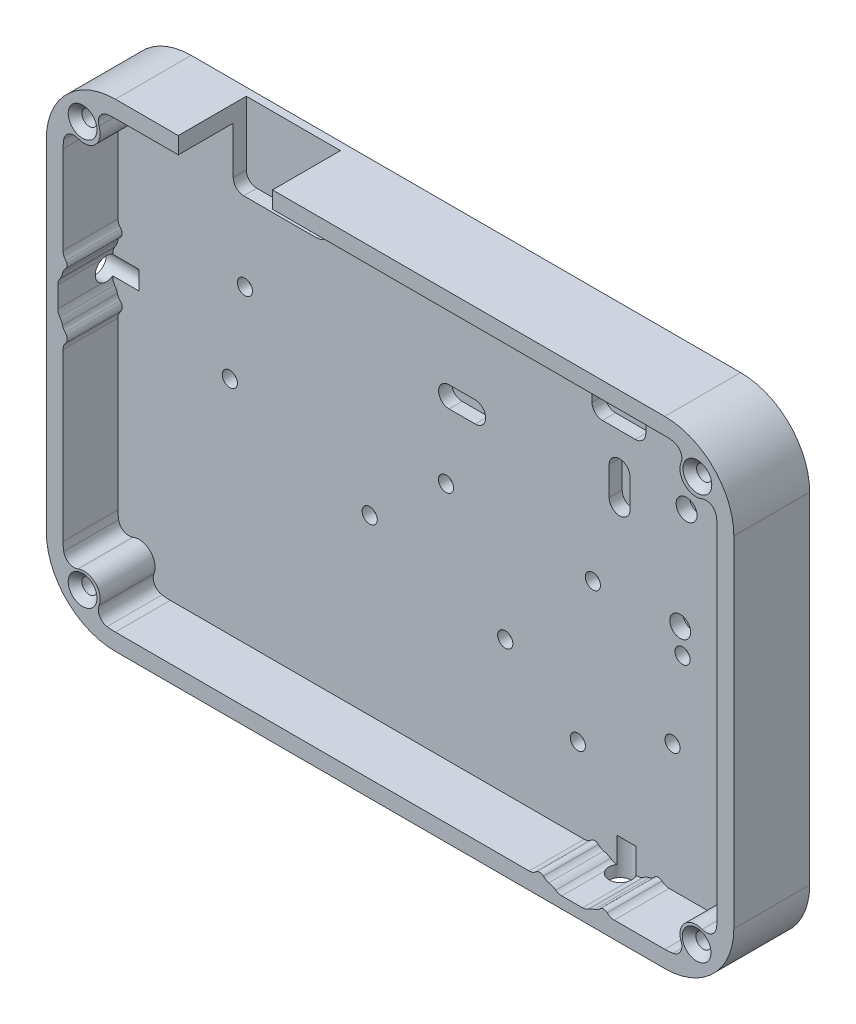
SolidWorks part; units mm, degrees
material "Легированная сталь"
ref_plane "Спереди" through (0, 0, 0) normal (0, 0, 1) x (1, 0, 0)
ref_plane "Сверху" through (0, 0, 0) normal (0, 1, 0) x (1, 0, 0)
ref_plane "Справа" through (0, 0, 0) normal (1, 0, 0) x (0, 0, -1)
sketch "Elements" plane through (0, 0, 0) normal (0, 0, 1) x (1, 0, 0)
  line L0 (-0.35, 0) -> (0.35, 0)
  line L1 (0, -0.35) -> (0, 0.35)
  line L2 (104.65, 65) -> (105.35, 65)
  line L3 (105, 64.65) -> (105, 65.35)
  line L4 (104.65, 0) -> (105.35, 0)
  line L5 (105, -0.35) -> (105, 0.35)
  line L6 (-0.35, 65) -> (0.35, 65)
  line L7 (0, 64.65) -> (0, 65.35)
  line L8 (87.2, -10.5) -> (87.2, -9.5)
  line L9 (93.2, -10) -> (93.2, -4.2)
  line L10 (81.2, -4.2) -> (93.2, -4.2)
  line L11 (81.2, -10) -> (81.2, -4.2)
  line L12 (80.2, -10) -> (94.2, -10)
  line L13 (85.7, -15) -> (88.7, -14)
  line L14 (85.7, -15.5) -> (88.7, -14.5)
  line L15 (85.7, -16) -> (88.7, -15)
  line L16 (85.7, -16.5) -> (88.7, -15.5)
  line L17 (85.7, -17) -> (88.7, -16)
  line L18 (85.7, -17.5) -> (88.7, -16.5)
  line L19 (85.7, -18) -> (88.7, -17)
  line L20 (85.7, -18.5) -> (88.7, -17.5)
  line L21 (85.7, -19.5) -> (85.7, -11.5)
  line L22 (85.7, -19.5) -> (88.7, -19.5)
  line L23 (88.7, -19.5) -> (88.7, -11.5)
  line L24 (90.9, -10) -> (90.9, -5.25)
  line L25 (90.9, -5.25) -> (91.9, -5.25)
  line L26 (91.9, -10) -> (91.9, -5.25)
  line L27 (83.5, -10) -> (83.5, -5.25)
  line L28 (82.5, -5.25) -> (83.5, -5.25)
  line L29 (82.5, -10) -> (82.5, -5.25)
  line L30 (82.5, -10) -> (91.9, -10)
  line L31 (91.9, -11.5) -> (91.9, -10)
  line L32 (82.5, -11.5) -> (91.9, -11.5)
  line L33 (82.5, -11.5) -> (82.5, -10)
  line L34 (86.65, -5.225) -> (87.75, -5.225)
  line L35 (87.75, -10) -> (87.75, -5.225)
  line L36 (86.65, -10) -> (86.65, -5.225)
  line L37 (85.9, -9.7) -> (85.9, -4.8719) construction
  line L38 (94.225, 24.265) -> (94.225, 24.935)
  line L39 (93.89, 24.6) -> (94.56, 24.6)
  line L40 (92.855, 25.27) -> (95.595, 25.27)
  line L41 (92.855, 23.93) -> (92.855, 25.27)
  line L42 (92.855, 23.93) -> (95.595, 23.93)
  line L43 (95.595, 23.93) -> (95.595, 25.27)
  line L44 (93.425, 25) -> (95.025, 25)
  line L45 (93.425, 24.2) -> (93.425, 25)
  line L46 (93.425, 24.2) -> (95.025, 24.2)
  line L47 (95.025, 24.2) -> (95.025, 25)
  line L48 (96.325, 23.7) -> (93.8875, 23.7) construction
  line L49 (-10.5, 40) -> (-9.5, 40)
  line L50 (-10, 34) -> (-4.2, 34)
  line L51 (-4.2, 34) -> (-4.2, 46)
  line L52 (-10, 46) -> (-4.2, 46)
  line L53 (-10, 33) -> (-10, 47)
  line L54 (-15, 41.5) -> (-14, 38.5)
  line L55 (-15.5, 41.5) -> (-14.5, 38.5)
  line L56 (-16, 41.5) -> (-15, 38.5)
  line L57 (-16.5, 41.5) -> (-15.5, 38.5)
  line L58 (-17, 41.5) -> (-16, 38.5)
  line L59 (-17.5, 41.5) -> (-16.5, 38.5)
  line L60 (-18, 41.5) -> (-17, 38.5)
  line L61 (-18.5, 41.5) -> (-17.5, 38.5)
  line L62 (-19.5, 41.5) -> (-11.5, 41.5)
  line L63 (-19.5, 38.5) -> (-19.5, 41.5)
  line L64 (-19.5, 38.5) -> (-11.5, 38.5)
  line L65 (-10, 36.3) -> (-5.25, 36.3)
  line L66 (-5.25, 35.3) -> (-5.25, 36.3)
  line L67 (-10, 35.3) -> (-5.25, 35.3)
  line L68 (-10, 43.7) -> (-5.25, 43.7)
  line L69 (-5.25, 43.7) -> (-5.25, 44.7)
  line L70 (-10, 44.7) -> (-5.25, 44.7)
  line L71 (-10, 35.3) -> (-10, 44.7)
  line L72 (-11.5, 35.3) -> (-10, 35.3)
  line L73 (-11.5, 35.3) -> (-11.5, 44.7)
  line L74 (-11.5, 44.7) -> (-10, 44.7)
  line L75 (-5.225, 39.45) -> (-5.225, 40.55)
  line L76 (-10, 39.45) -> (-5.225, 39.45)
  line L77 (-10, 40.55) -> (-5.225, 40.55)
  line L78 (68.23, 59.48) -> (68.23, 64.98)
  line L79 (68.23, 64.98) -> (71.77, 64.98)
  line L80 (71.77, 59.48) -> (71.77, 64.98)
  line L81 (68.23, 59.48) -> (71.77, 59.48)
  line L82 (69.65, 63.5) -> (70.35, 63.5)
  line L83 (70, 63.15) -> (70, 63.85)
  line L84 (68.5, 59.73) -> (68.5, 63.73)
  line L85 (68.5, 63.73) -> (69.5, 64.73)
  line L86 (69.5, 64.73) -> (71.5, 64.73)
  line L87 (71.5, 59.73) -> (71.5, 64.73)
  line L88 (68.5, 59.73) -> (71.5, 59.73)
  line L89 (68.7, 61.9) -> (73.0594, 61.9) construction
  line L90 (21.025, 83.175) -> (21.025, 84.175)
  line L91 (13.025, 64.975) -> (13.025, 83.675)
  line L92 (13.025, 64.975) -> (29.025, 64.975)
  line L93 (29.025, 64.975) -> (29.025, 83.675)
  line L94 (13.025, 83.675) -> (29.025, 83.675)
  line L95 (21.025, 66.975) -> (21.025, 67.675)
  line L96 (20.675, 67.325) -> (21.375, 67.325)
  line L97 (13.3184, 75.025) -> (28.7953, 75.025)
  line L98 (15.025, 65.475) -> (24.525, 65.475)
  line L99 (24.525, 65.475) -> (27.025, 65.475)
  line L100 (13.275, 69.6999) -> (13.275, 75.025)
  line L101 (28.775, 69.6999) -> (28.775, 75.025)
  line L102 (88.2, 61.825) -> (94.8, 61.825)
  line L103 (88.2, 73.175) -> (94.8, 73.175)
  line L104 (88.2, 61.825) -> (88.2, 73.175)
  line L105 (94.8, 61.825) -> (94.8, 73.175)
  line L106 (91.5, 67) -> (91.5, 68)
  line L107 (91, 67.5) -> (92, 67.5)
  line L108 (88.45, 64.45) -> (94.55, 64.45)
  line L109 (88.45, 70.55) -> (94.55, 70.55)
  line L110 (88.45, 64.45) -> (88.45, 70.55)
  line L111 (94.55, 64.45) -> (94.55, 70.55)
  line L112 (81.4925, 46.5358) -> (83.2925, 46.5358)
  line L113 (81.4925, 45.6358) -> (81.4925, 46.5358)
  line L114 (81.4925, 45.6358) -> (83.2925, 45.6358)
  line L115 (83.2925, 45.6358) -> (83.2925, 46.5358)
  line L116 (82.3925, 45.8658) -> (82.3925, 46.3058)
  line L117 (82.1725, 46.0858) -> (82.6125, 46.0858)
  line L118 (81.8925, 46.3358) -> (82.8925, 46.3358)
  line L119 (81.8925, 45.8358) -> (81.8925, 46.3358)
  line L120 (81.8925, 45.8358) -> (82.8925, 45.8358)
  line L121 (82.8925, 45.8358) -> (82.8925, 46.3358)
  line L122 (81.9375, 48.9108) -> (81.9375, 45.0201) construction
  line L123 (94.385, 53.9133) -> (96.185, 53.9133)
  line L124 (96.185, 53.9133) -> (96.185, 54.8133)
  line L125 (94.385, 54.8133) -> (96.185, 54.8133)
  line L126 (94.385, 53.9133) -> (94.385, 54.8133)
  line L127 (95.285, 54.1433) -> (95.285, 54.5833)
  line L128 (95.065, 54.3633) -> (95.505, 54.3633)
  line L129 (94.785, 54.1133) -> (95.785, 54.1133)
  line L130 (95.785, 54.1133) -> (95.785, 54.6133)
  line L131 (94.785, 54.6133) -> (95.785, 54.6133)
  line L132 (94.785, 54.1133) -> (94.785, 54.6133)
  line L133 (96.225, 55.9883) -> (92.3344, 55.9883) construction
  line L134 (87.05, 43.3556) -> (88.85, 43.3556)
  line L135 (88.85, 43.3556) -> (88.85, 44.2556)
  line L136 (87.05, 44.2556) -> (88.85, 44.2556)
  line L137 (87.05, 43.3556) -> (87.05, 44.2556)
  line L138 (87.95, 43.5856) -> (87.95, 44.0256)
  line L139 (87.73, 43.8056) -> (88.17, 43.8056)
  line L140 (87.45, 43.5556) -> (88.45, 43.5556)
  line L141 (88.45, 43.5556) -> (88.45, 44.0556)
  line L142 (87.45, 44.0556) -> (88.45, 44.0556)
  line L143 (87.45, 43.5556) -> (87.45, 44.0556)
  line L144 (91.56, 44.2306) -> (88.1381, 44.2306) construction
  line L145 (88.86, 41.3656) -> (88.86, 43.1656)
  line L146 (87.96, 43.1656) -> (88.86, 43.1656)
  line L147 (87.96, 41.3656) -> (87.96, 43.1656)
  line L148 (87.96, 41.3656) -> (88.86, 41.3656)
  line L149 (88.19, 42.2656) -> (88.63, 42.2656)
  line L150 (88.41, 42.0456) -> (88.41, 42.4856)
  line L151 (88.66, 41.7656) -> (88.66, 42.7656)
  line L152 (88.16, 42.7656) -> (88.66, 42.7656)
  line L153 (88.16, 41.7656) -> (88.16, 42.7656)
  line L154 (88.16, 41.7656) -> (88.66, 41.7656)
  line L155 (91.66, 42.4806) -> (88.0038, 42.4806) construction
  line L156 (91.8202, 42.4931) -> (91.8202, 44.2931)
  line L157 (90.9202, 44.2931) -> (91.8202, 44.2931)
  line L158 (90.9202, 42.4931) -> (90.9202, 44.2931)
  line L159 (90.9202, 42.4931) -> (91.8202, 42.4931)
  line L160 (91.1502, 43.3931) -> (91.5902, 43.3931)
  line L161 (91.3702, 43.1731) -> (91.3702, 43.6131)
  line L162 (91.6202, 42.8931) -> (91.6202, 43.8931)
  line L163 (91.1202, 43.8931) -> (91.6202, 43.8931)
  line L164 (91.1202, 42.8931) -> (91.1202, 43.8931)
  line L165 (91.1202, 42.8931) -> (91.6202, 42.8931)
  line L166 (92.0702, 43.0331) -> (94.9764, 43.0331) construction
  line L167 (92.2249, 34.0083) -> (92.2249, 35.8083)
  line L168 (92.2249, 34.0083) -> (93.1249, 34.0083)
  line L169 (93.1249, 34.0083) -> (93.1249, 35.8083)
  line L170 (92.2249, 35.8083) -> (93.1249, 35.8083)
  line L171 (92.4549, 34.9083) -> (92.8949, 34.9083)
  line L172 (92.6749, 34.6883) -> (92.6749, 35.1283)
  line L173 (92.4249, 34.4083) -> (92.4249, 35.4083)
  line L174 (92.4249, 34.4083) -> (92.9249, 34.4083)
  line L175 (92.9249, 34.4083) -> (92.9249, 35.4083)
  line L176 (92.4249, 35.4083) -> (92.9249, 35.4083)
  line L177 (92.1999, 37.5983) -> (92.1999, 34.692) construction
  line L178 (93.4399, 34.8733) -> (95.2399, 34.8733)
  line L179 (93.4399, 33.9733) -> (93.4399, 34.8733)
  line L180 (93.4399, 33.9733) -> (95.2399, 33.9733)
  line L181 (95.2399, 33.9733) -> (95.2399, 34.8733)
  line L182 (94.3399, 34.2033) -> (94.3399, 34.6433)
  line L183 (94.1199, 34.4233) -> (94.5599, 34.4233)
  line L184 (93.8399, 34.6733) -> (94.8399, 34.6733)
  line L185 (93.8399, 34.1733) -> (93.8399, 34.6733)
  line L186 (93.8399, 34.1733) -> (94.8399, 34.1733)
  line L187 (94.8399, 34.1733) -> (94.8399, 34.6733)
  line L188 (93.5249, 37.5233) -> (93.5249, 34.617) construction
  line L189 (95.4249, 33.9833) -> (95.4249, 35.7833)
  line L190 (95.4249, 33.9833) -> (96.3249, 33.9833)
  line L191 (96.3249, 33.9833) -> (96.3249, 35.7833)
  line L192 (95.4249, 35.7833) -> (96.3249, 35.7833)
  line L193 (95.6549, 34.8833) -> (96.0949, 34.8833)
  line L194 (95.8749, 34.6633) -> (95.8749, 35.1033)
  line L195 (95.6249, 34.3833) -> (95.6249, 35.3833)
  line L196 (95.6249, 34.3833) -> (96.1249, 34.3833)
  line L197 (96.1249, 34.3833) -> (96.1249, 35.3833)
  line L198 (95.6249, 35.3833) -> (96.1249, 35.3833)
  line L199 (95.3999, 37.5483) -> (95.3999, 34.642) construction
  line L200 (70.115, 36.6733) -> (71.915, 36.6733)
  line L201 (70.115, 35.7733) -> (70.115, 36.6733)
  line L202 (70.115, 35.7733) -> (71.915, 35.7733)
  line L203 (71.915, 35.7733) -> (71.915, 36.6733)
  line L204 (71.015, 36.0033) -> (71.015, 36.4433)
  line L205 (70.795, 36.2233) -> (71.235, 36.2233)
  line L206 (70.515, 36.4733) -> (71.515, 36.4733)
  line L207 (70.515, 35.9733) -> (70.515, 36.4733)
  line L208 (70.515, 35.9733) -> (71.515, 35.9733)
  line L209 (71.515, 35.9733) -> (71.515, 36.4733)
  line L210 (69.675, 35.5233) -> (69.675, 38.4295) construction
  line L211 (70.83, 39.9883) -> (72.17, 39.9883)
  line L212 (72.17, 37.2483) -> (72.17, 39.9883)
  line L213 (70.83, 37.2483) -> (72.17, 37.2483)
  line L214 (70.83, 37.2483) -> (70.83, 39.9883)
  line L215 (71.5, 38.2833) -> (71.5, 38.9533)
  line L216 (71.165, 38.6183) -> (71.835, 38.6183)
  line L217 (71.1, 39.4183) -> (71.9, 39.4183)
  line L218 (71.9, 37.8183) -> (71.9, 39.4183)
  line L219 (71.1, 37.8183) -> (71.9, 37.8183)
  line L220 (71.1, 37.8183) -> (71.1, 39.4183)
  line L221 (70.7, 38.0233) -> (70.7, 40.9295) construction
  line L222 (5.95, 51.9233) -> (7.75, 51.9233)
  line L223 (5.95, 51.0233) -> (5.95, 51.9233)
  line L224 (5.95, 51.0233) -> (7.75, 51.0233)
  line L225 (7.75, 51.0233) -> (7.75, 51.9233)
  line L226 (6.85, 51.2533) -> (6.85, 51.6933)
  line L227 (6.63, 51.4733) -> (7.07, 51.4733)
  line L228 (6.35, 51.7233) -> (7.35, 51.7233)
  line L229 (6.35, 51.2233) -> (6.35, 51.7233)
  line L230 (6.35, 51.2233) -> (7.35, 51.2233)
  line L231 (7.35, 51.2233) -> (7.35, 51.7233)
  line L232 (8.65, 51.0483) -> (11.5563, 51.0483) construction
  line L233 (6.83, 55.4383) -> (8.17, 55.4383)
  line L234 (8.17, 52.6983) -> (8.17, 55.4383)
  line L235 (6.83, 52.6983) -> (8.17, 52.6983)
  line L236 (6.83, 52.6983) -> (6.83, 55.4383)
  line L237 (7.5, 53.7333) -> (7.5, 54.4033)
  line L238 (7.165, 54.0683) -> (7.835, 54.0683)
  line L239 (7.1, 54.8683) -> (7.9, 54.8683)
  line L240 (7.9, 53.2683) -> (7.9, 54.8683)
  line L241 (7.1, 53.2683) -> (7.9, 53.2683)
  line L242 (7.1, 53.2683) -> (7.1, 54.8683)
  line L243 (7.225, 56.1233) -> (10.1313, 56.1233) construction
  line L244 (87.27, 51.6483) -> (88.27, 51.6483)
  line L245 (87.77, 51.1483) -> (87.77, 52.1483)
  line L246 (85.02, 47.9733) -> (85.02, 55.3233)
  line L247 (90.52, 47.9733) -> (90.52, 55.3233)
  line L248 (85.02, 47.9733) -> (90.52, 47.9733)
  line L249 (85.02, 55.3233) -> (90.52, 55.3233)
  line L250 (85.27, 49.6483) -> (85.27, 53.6483)
  line L251 (90.27, 49.6483) -> (90.27, 53.6483)
  line L252 (85.27, 49.6483) -> (90.27, 49.6483)
  line L253 (85.27, 53.6483) -> (90.27, 53.6483)
  line L254 (87.7249, 35.3733) -> (88.7249, 35.3733)
  line L255 (88.2249, 34.8733) -> (88.2249, 35.8733)
  line L256 (86.9249, 33.9233) -> (86.9249, 36.8233)
  line L257 (86.9249, 33.9233) -> (89.5249, 33.9233)
  line L258 (86.9249, 36.8233) -> (89.5249, 36.8233)
  line L259 (89.5249, 33.9233) -> (89.5249, 36.8233)
  line L260 (87.1749, 34.3233) -> (87.1749, 36.4233)
  line L261 (89.2749, 34.3233) -> (89.2749, 36.4233)
  line L262 (87.1749, 34.3233) -> (89.2749, 34.3233)
  line L263 (87.1749, 36.4233) -> (89.2749, 36.4233)
  line L264 (88.9999, 35.7316) -> (84.6405, 35.7316) construction
  line L265 (70.5, 23.8483) -> (71.5, 23.8483)
  line L266 (71, 23.3483) -> (71, 24.3483)
  line L267 (68.65, 21.9983) -> (68.65, 25.6983)
  line L268 (73.35, 21.9983) -> (73.35, 25.6983)
  line L269 (68.65, 21.9983) -> (73.35, 21.9983)
  line L270 (68.65, 25.6983) -> (73.35, 25.6983)
  line L271 (69.2, 22.5483) -> (69.2, 25.1483)
  line L272 (72.8, 22.5483) -> (72.8, 25.1483)
  line L273 (69.2, 22.5483) -> (72.8, 22.5483)
  line L274 (69.2, 25.1483) -> (72.8, 25.1483)
  line L275 (74.2149, 21.7691) -> (69.8555, 21.7691) construction
  line L276 (6.4, 39.9483) -> (7.4, 39.9483)
  line L277 (6.9, 39.4483) -> (6.9, 40.4483)
  line L278 (4.55, 38.0983) -> (4.55, 41.7983)
  line L279 (9.25, 38.0983) -> (9.25, 41.7983)
  line L280 (4.55, 38.0983) -> (9.25, 38.0983)
  line L281 (4.55, 41.7983) -> (9.25, 41.7983)
  line L282 (5.1, 38.6483) -> (5.1, 41.2483)
  line L283 (8.7, 38.6483) -> (8.7, 41.2483)
  line L284 (5.1, 38.6483) -> (8.7, 38.6483)
  line L285 (5.1, 41.2483) -> (8.7, 41.2483)
  line L286 (10.1149, 37.8858) -> (5.7555, 37.8858) construction
  line L287 (53.425, 58.2233) -> (54.125, 58.2233)
  line L288 (53.775, 57.8733) -> (53.775, 58.5733)
  line L289 (51.075, 54.5633) -> (56.475, 54.5633)
  line L290 (56.475, 54.5633) -> (56.475, 61.8833)
  line L291 (51.075, 61.8833) -> (56.475, 61.8833)
  line L292 (51.075, 54.5633) -> (51.075, 61.8833)
  line L293 (51.325, 56.2733) -> (56.225, 56.2733)
  line L294 (56.225, 56.2733) -> (56.225, 60.1733)
  line L295 (51.325, 60.1733) -> (56.225, 60.1733)
  line L296 (51.325, 56.2733) -> (51.325, 60.1733)
  line L297 (51.5221, 57.9278) -> (55.0096, 57.9278) construction
  line L298 (35.4, 58.2233) -> (36.1, 58.2233)
  line L299 (35.75, 57.8733) -> (35.75, 58.5733)
  line L300 (33.05, 54.5633) -> (38.45, 54.5633)
  line L301 (38.45, 54.5633) -> (38.45, 61.8833)
  line L302 (33.05, 61.8833) -> (38.45, 61.8833)
  line L303 (33.05, 54.5633) -> (33.05, 61.8833)
  line L304 (33.3, 56.2733) -> (38.2, 56.2733)
  line L305 (38.2, 56.2733) -> (38.2, 60.1733)
  line L306 (33.3, 60.1733) -> (38.2, 60.1733)
  line L307 (33.3, 56.2733) -> (33.3, 60.1733)
  line L308 (33.4971, 57.9278) -> (36.9846, 57.9278) construction
  line L309 (44.9, 58.2233) -> (45.6, 58.2233)
  line L310 (45.25, 57.8733) -> (45.25, 58.5733)
  line L311 (42.55, 54.5633) -> (47.95, 54.5633)
  line L312 (47.95, 54.5633) -> (47.95, 61.8833)
  line L313 (42.55, 61.8833) -> (47.95, 61.8833)
  line L314 (42.55, 54.5633) -> (42.55, 61.8833)
  line L315 (42.8, 56.2733) -> (47.7, 56.2733)
  line L316 (47.7, 56.2733) -> (47.7, 60.1733)
  line L317 (42.8, 60.1733) -> (47.7, 60.1733)
  line L318 (42.8, 56.2733) -> (42.8, 60.1733)
  line L319 (42.9971, 57.9278) -> (46.1096, 57.9278) construction
  line L320 (80.6925, 45.6008) -> (81.1325, 45.6008)
  line L321 (80.9125, 45.3808) -> (80.9125, 45.8208)
  line L322 (81.3525, 44.7008) -> (81.3525, 46.5008)
  line L323 (80.4725, 46.5008) -> (81.3525, 46.5008)
  line L324 (80.4725, 44.7008) -> (80.4725, 46.5008)
  line L325 (80.4725, 44.7008) -> (81.3525, 44.7008)
  line L326 (81.1625, 45.1008) -> (81.1625, 46.1008)
  line L327 (80.6625, 46.1008) -> (81.1625, 46.1008)
  line L328 (80.6625, 45.1008) -> (80.6625, 46.1008)
  line L329 (80.6625, 45.1008) -> (81.1625, 45.1008)
  line L330 (81.4375, 42.0608) -> (81.4375, 46.1858) construction
  line L331 (83.6675, 45.5758) -> (84.1075, 45.5758)
  line L332 (83.8875, 45.3558) -> (83.8875, 45.7958)
  line L333 (84.3275, 44.6758) -> (84.3275, 46.4758)
  line L334 (83.4475, 46.4758) -> (84.3275, 46.4758)
  line L335 (83.4475, 44.6758) -> (83.4475, 46.4758)
  line L336 (83.4475, 44.6758) -> (84.3275, 44.6758)
  line L337 (84.1375, 45.0758) -> (84.1375, 46.0758)
  line L338 (83.6375, 46.0758) -> (84.1375, 46.0758)
  line L339 (83.6375, 45.0758) -> (83.6375, 46.0758)
  line L340 (83.6375, 45.0758) -> (84.1375, 45.0758)
  line L341 (84.2375, 42.0608) -> (84.2375, 46.4201) construction
  line L342 (93.58, 53.8883) -> (94.02, 53.8883)
  line L343 (93.8, 53.6683) -> (93.8, 54.1083)
  line L344 (94.24, 52.9883) -> (94.24, 54.7883)
  line L345 (93.36, 54.7883) -> (94.24, 54.7883)
  line L346 (93.36, 52.9883) -> (93.36, 54.7883)
  line L347 (93.36, 52.9883) -> (94.24, 52.9883)
  line L348 (94.05, 53.3883) -> (94.05, 54.3883)
  line L349 (93.55, 54.3883) -> (94.05, 54.3883)
  line L350 (93.55, 53.3883) -> (93.55, 54.3883)
  line L351 (93.55, 53.3883) -> (94.05, 53.3883)
  line L352 (93.125, 55.6133) -> (88.7656, 55.6133) construction
  line L353 (96.78, 53.8883) -> (97.22, 53.8883)
  line L354 (97, 53.6683) -> (97, 54.1083)
  line L355 (97.44, 52.9883) -> (97.44, 54.7883)
  line L356 (96.56, 54.7883) -> (97.44, 54.7883)
  line L357 (96.56, 52.9883) -> (96.56, 54.7883)
  line L358 (96.56, 52.9883) -> (97.44, 52.9883)
  line L359 (97.25, 53.3883) -> (97.25, 54.3883)
  line L360 (96.75, 54.3883) -> (97.25, 54.3883)
  line L361 (96.75, 53.3883) -> (96.75, 54.3883)
  line L362 (96.75, 53.3883) -> (97.25, 53.3883)
  line L363 (99.725, 56.0633) -> (95.3656, 56.0633) construction
  line L364 (87.92, 44.7356) -> (87.92, 45.1756)
  line L365 (87.7, 44.9556) -> (88.14, 44.9556)
  line L366 (87.02, 44.5156) -> (88.82, 44.5156)
  line L367 (88.82, 44.5156) -> (88.82, 45.3956)
  line L368 (87.02, 45.3956) -> (88.82, 45.3956)
  line L369 (87.02, 44.5156) -> (87.02, 45.3956)
  line L370 (87.42, 44.7056) -> (88.42, 44.7056)
  line L371 (88.42, 44.7056) -> (88.42, 45.2056)
  line L372 (87.42, 45.2056) -> (88.42, 45.2056)
  line L373 (87.42, 44.7056) -> (87.42, 45.2056)
  line L374 (91.735, 45.3556) -> (87.3756, 45.3556) construction
  line L375 (90.8852, 44.6731) -> (90.8852, 45.1131)
  line L376 (90.6652, 44.8931) -> (91.1052, 44.8931)
  line L377 (89.9852, 44.4531) -> (91.7852, 44.4531)
  line L378 (91.7852, 44.4531) -> (91.7852, 45.3331)
  line L379 (89.9852, 45.3331) -> (91.7852, 45.3331)
  line L380 (89.9852, 44.4531) -> (89.9852, 45.3331)
  line L381 (90.3852, 44.6431) -> (91.3852, 44.6431)
  line L382 (91.3852, 44.6431) -> (91.3852, 45.1431)
  line L383 (90.3852, 45.1431) -> (91.3852, 45.1431)
  line L384 (90.3852, 44.6431) -> (90.3852, 45.1431)
  line L385 (92.0452, 44.5931) -> (96.4045, 44.5931) construction
  line L386 (87.95, 40.5106) -> (87.95, 40.9506)
  line L387 (87.73, 40.7306) -> (88.17, 40.7306)
  line L388 (87.05, 40.2906) -> (88.85, 40.2906)
  line L389 (88.85, 40.2906) -> (88.85, 41.1706)
  line L390 (87.05, 41.1706) -> (88.85, 41.1706)
  line L391 (87.05, 40.2906) -> (87.05, 41.1706)
  line L392 (87.45, 40.4806) -> (88.45, 40.4806)
  line L393 (88.45, 40.4806) -> (88.45, 40.9806)
  line L394 (87.45, 40.9806) -> (88.45, 40.9806)
  line L395 (87.45, 40.4806) -> (87.45, 40.9806)
  line L396 (91.61, 41.1556) -> (87.2506, 41.1556) construction
  line L397 (91.8802, 41.5731) -> (91.8802, 42.0131)
  line L398 (91.6602, 41.7931) -> (92.1002, 41.7931)
  line L399 (90.9802, 42.2331) -> (92.7802, 42.2331)
  line L400 (90.9802, 41.3531) -> (90.9802, 42.2331)
  line L401 (90.9802, 41.3531) -> (92.7802, 41.3531)
  line L402 (92.7802, 41.3531) -> (92.7802, 42.2331)
  line L403 (91.3802, 42.0431) -> (92.3802, 42.0431)
  line L404 (91.3802, 41.5431) -> (91.3802, 42.0431)
  line L405 (91.3802, 41.5431) -> (92.3802, 41.5431)
  line L406 (92.3802, 41.5431) -> (92.3802, 42.0431)
  line L407 (90.6952, 42.2431) -> (86.3358, 42.2431) construction
  line L408 (91.0549, 34.9333) -> (91.4949, 34.9333)
  line L409 (91.2749, 34.7133) -> (91.2749, 35.1533)
  line L410 (90.8349, 34.0333) -> (90.8349, 35.8333)
  line L411 (90.8349, 34.0333) -> (91.7149, 34.0333)
  line L412 (91.7149, 34.0333) -> (91.7149, 35.8333)
  line L413 (90.8349, 35.8333) -> (91.7149, 35.8333)
  line L414 (91.0249, 34.4333) -> (91.0249, 35.4333)
  line L415 (91.0249, 34.4333) -> (91.5249, 34.4333)
  line L416 (91.5249, 34.4333) -> (91.5249, 35.4333)
  line L417 (91.0249, 35.4333) -> (91.5249, 35.4333)
  line L418 (90.7499, 38.3733) -> (90.7499, 34.0139) construction
  line L419 (70.98, 32.4833) -> (70.98, 34.2633)
  line L420 (67.84, 32.4833) -> (70.98, 32.4833)
  line L421 (67.84, 32.4833) -> (67.84, 34.2633)
  line L422 (67.84, 34.2633) -> (70.98, 34.2633)
  line L423 (69.06, 33.3733) -> (69.76, 33.3733)
  line L424 (69.41, 33.0233) -> (69.41, 33.7233)
  line L425 (70.46, 32.6933) -> (70.46, 34.0533)
  line L426 (68.36, 32.6933) -> (70.46, 32.6933)
  line L427 (68.36, 32.6933) -> (68.36, 34.0533)
  line L428 (68.36, 34.0533) -> (70.46, 34.0533)
  line L429 (68.45, 31.3233) -> (72.3406, 31.3233) construction
  line L430 (68.225, 29.7983) -> (70.975, 29.7983)
  line L431 (68.225, 29.7983) -> (68.225, 31.1483)
  line L432 (69.265, 30.4733) -> (69.935, 30.4733)
  line L433 (69.6, 30.1383) -> (69.6, 30.8083)
  line L434 (68.225, 31.1483) -> (70.975, 31.1483)
  line L435 (70.975, 29.7983) -> (70.975, 31.1483)
  line L436 (70.4, 30.0733) -> (70.4, 30.8733)
  line L437 (68.8, 30.0733) -> (70.4, 30.0733)
  line L438 (68.8, 30.0733) -> (68.8, 30.8733)
  line L439 (68.8, 30.8733) -> (70.4, 30.8733)
  line L440 (68.3, 28.7233) -> (72.425, 28.7233) construction
  line L441 (70.0063, 27.9033) -> (70.0063, 28.3433)
  line L442 (69.7863, 28.1233) -> (70.2263, 28.1233)
  line L443 (69.1063, 28.5633) -> (70.9063, 28.5633)
  line L444 (69.1063, 27.6833) -> (69.1063, 28.5633)
  line L445 (69.1063, 27.6833) -> (70.9063, 27.6833)
  line L446 (70.9063, 27.6833) -> (70.9063, 28.5633)
  line L447 (69.5063, 28.3733) -> (70.5063, 28.3733)
  line L448 (69.5063, 27.8733) -> (69.5063, 28.3733)
  line L449 (69.5063, 27.8733) -> (70.5063, 27.8733)
  line L450 (70.5063, 27.8733) -> (70.5063, 28.3733)
  line L451 (68.3063, 26.5733) -> (72.1969, 26.5733) construction
  line L452 (74.16, 32.4833) -> (74.16, 34.2633)
  line L453 (71.02, 32.4833) -> (74.16, 32.4833)
  line L454 (71.02, 32.4833) -> (71.02, 34.2633)
  line L455 (71.02, 34.2633) -> (74.16, 34.2633)
  line L456 (72.24, 33.3733) -> (72.94, 33.3733)
  line L457 (72.59, 33.0233) -> (72.59, 33.7233)
  line L458 (73.64, 32.6933) -> (73.64, 34.0533)
  line L459 (71.54, 32.6933) -> (73.64, 32.6933)
  line L460 (71.54, 32.6933) -> (71.54, 34.0533)
  line L461 (71.54, 34.0533) -> (73.64, 34.0533)
  line L462 (71.7, 31.3483) -> (75.5906, 31.3483) construction
  line L463 (71.025, 29.7983) -> (73.775, 29.7983)
  line L464 (71.025, 29.7983) -> (71.025, 31.1483)
  line L465 (72.065, 30.4733) -> (72.735, 30.4733)
  line L466 (72.4, 30.1383) -> (72.4, 30.8083)
  line L467 (71.025, 31.1483) -> (73.775, 31.1483)
  line L468 (73.775, 29.7983) -> (73.775, 31.1483)
  line L469 (73.2, 30.0733) -> (73.2, 30.8733)
  line L470 (71.6, 30.0733) -> (73.2, 30.0733)
  line L471 (71.6, 30.0733) -> (71.6, 30.8733)
  line L472 (71.6, 30.8733) -> (73.2, 30.8733)
  line L473 (71.55, 28.7983) -> (75.4406, 28.7983) construction
  line L474 (71.9938, 27.9033) -> (71.9938, 28.3433)
  line L475 (71.7738, 28.1233) -> (72.2138, 28.1233)
  line L476 (71.0938, 28.5633) -> (72.8938, 28.5633)
  line L477 (71.0938, 27.6833) -> (71.0938, 28.5633)
  line L478 (71.0938, 27.6833) -> (72.8938, 27.6833)
  line L479 (72.8938, 27.6833) -> (72.8938, 28.5633)
  line L480 (71.4938, 28.3733) -> (72.4938, 28.3733)
  line L481 (71.4938, 27.8733) -> (71.4938, 28.3733)
  line L482 (71.4938, 27.8733) -> (72.4938, 27.8733)
  line L483 (72.4938, 27.8733) -> (72.4938, 28.3733)
  line L484 (71.6188, 26.5733) -> (75.5094, 26.5733) construction
  line L485 (6.805, 48.0833) -> (6.805, 49.8633)
  line L486 (3.665, 48.0833) -> (6.805, 48.0833)
  line L487 (3.665, 48.0833) -> (3.665, 49.8633)
  line L488 (3.665, 49.8633) -> (6.805, 49.8633)
  line L489 (4.885, 48.9733) -> (5.585, 48.9733)
  line L490 (5.235, 48.6233) -> (5.235, 49.3233)
  line L491 (6.285, 48.2933) -> (6.285, 49.6533)
  line L492 (4.185, 48.2933) -> (6.285, 48.2933)
  line L493 (4.185, 48.2933) -> (4.185, 49.6533)
  line L494 (4.185, 49.6533) -> (6.285, 49.6533)
  line L495 (4.1, 46.9983) -> (7.9906, 46.9983) construction
  line L496 (4.07, 45.2983) -> (6.82, 45.2983)
  line L497 (4.07, 45.2983) -> (4.07, 46.6483)
  line L498 (5.11, 45.9733) -> (5.78, 45.9733)
  line L499 (5.445, 45.6383) -> (5.445, 46.3083)
  line L500 (4.07, 46.6483) -> (6.82, 46.6483)
  line L501 (6.82, 45.2983) -> (6.82, 46.6483)
  line L502 (6.245, 45.5733) -> (6.245, 46.3733)
  line L503 (4.645, 45.5733) -> (6.245, 45.5733)
  line L504 (4.645, 45.5733) -> (4.645, 46.3733)
  line L505 (4.645, 46.3733) -> (6.245, 46.3733)
  line L506 (4.425, 44.2483) -> (8.3156, 44.2483) construction
  line L507 (5.89, 43.2533) -> (5.89, 43.6933)
  line L508 (5.67, 43.4733) -> (6.11, 43.4733)
  line L509 (4.99, 43.9133) -> (6.79, 43.9133)
  line L510 (4.99, 43.0333) -> (4.99, 43.9133)
  line L511 (4.99, 43.0333) -> (6.79, 43.0333)
  line L512 (6.79, 43.0333) -> (6.79, 43.9133)
  line L513 (5.39, 43.7233) -> (6.39, 43.7233)
  line L514 (5.39, 43.2233) -> (5.39, 43.7233)
  line L515 (5.39, 43.2233) -> (6.39, 43.2233)
  line L516 (6.39, 43.2233) -> (6.39, 43.7233)
  line L517 (3.875, 41.9733) -> (7.7656, 41.9733) construction
  line L518 (9.985, 48.0833) -> (9.985, 49.8633)
  line L519 (6.845, 48.0833) -> (9.985, 48.0833)
  line L520 (6.845, 48.0833) -> (6.845, 49.8633)
  line L521 (6.845, 49.8633) -> (9.985, 49.8633)
  line L522 (8.065, 48.9733) -> (8.765, 48.9733)
  line L523 (8.415, 48.6233) -> (8.415, 49.3233)
  line L524 (9.465, 48.2933) -> (9.465, 49.6533)
  line L525 (7.365, 48.2933) -> (9.465, 48.2933)
  line L526 (7.365, 48.2933) -> (7.365, 49.6533)
  line L527 (7.365, 49.6533) -> (9.465, 49.6533)
  line L528 (7.7, 47.0483) -> (11.5906, 47.0483) construction
  line L529 (6.855, 45.2983) -> (9.605, 45.2983)
  line L530 (6.855, 45.2983) -> (6.855, 46.6483)
  line L531 (7.895, 45.9733) -> (8.565, 45.9733)
  line L532 (8.23, 45.6383) -> (8.23, 46.3083)
  line L533 (6.855, 46.6483) -> (9.605, 46.6483)
  line L534 (9.605, 45.2983) -> (9.605, 46.6483)
  line L535 (9.03, 45.5733) -> (9.03, 46.3733)
  line L536 (7.43, 45.5733) -> (9.03, 45.5733)
  line L537 (7.43, 45.5733) -> (7.43, 46.3733)
  line L538 (7.43, 46.3733) -> (9.03, 46.3733)
  line L539 (7.675, 44.2483) -> (11.0969, 44.2483) construction
  line L540 (7.885, 43.2533) -> (7.885, 43.6933)
  line L541 (7.665, 43.4733) -> (8.105, 43.4733)
  line L542 (6.985, 43.9133) -> (8.785, 43.9133)
  line L543 (6.985, 43.0333) -> (6.985, 43.9133)
  line L544 (6.985, 43.0333) -> (8.785, 43.0333)
  line L545 (8.785, 43.0333) -> (8.785, 43.9133)
  line L546 (7.385, 43.7233) -> (8.385, 43.7233)
  line L547 (7.385, 43.2233) -> (7.385, 43.7233)
  line L548 (7.385, 43.2233) -> (8.385, 43.2233)
  line L549 (8.385, 43.2233) -> (8.385, 43.7233)
  line L550 (7.65, 41.9983) -> (11.3063, 41.9983) construction
  line L551 (52.05, 51.0233) -> (54.8, 51.0233)
  line L552 (54.8, 49.6733) -> (54.8, 51.0233)
  line L553 (53.09, 50.3483) -> (53.76, 50.3483)
  line L554 (53.425, 50.0133) -> (53.425, 50.6833)
  line L555 (52.05, 49.6733) -> (54.8, 49.6733)
  line L556 (52.05, 49.6733) -> (52.05, 51.0233)
  line L557 (52.625, 49.9483) -> (52.625, 50.7483)
  line L558 (52.625, 50.7483) -> (54.225, 50.7483)
  line L559 (54.225, 49.9483) -> (54.225, 50.7483)
  line L560 (52.625, 49.9483) -> (54.225, 49.9483)
  line L561 (50.625, 51.2483) -> (53.5313, 51.2483) construction
  line L562 (34.0105, 49.9483) -> (36.7605, 49.9483)
  line L563 (36.7605, 48.5983) -> (36.7605, 49.9483)
  line L564 (35.0505, 49.2733) -> (35.7205, 49.2733)
  line L565 (35.3855, 48.9383) -> (35.3855, 49.6083)
  line L566 (34.0105, 48.5983) -> (36.7605, 48.5983)
  line L567 (34.0105, 48.5983) -> (34.0105, 49.9483)
  line L568 (34.5855, 48.8733) -> (34.5855, 49.6733)
  line L569 (34.5855, 49.6733) -> (36.1855, 49.6733)
  line L570 (36.1855, 48.8733) -> (36.1855, 49.6733)
  line L571 (34.5855, 48.8733) -> (36.1855, 48.8733)
  line L572 (32.5855, 50.1733) -> (35.4918, 50.1733) construction
  line L573 (43.5, 49.9233) -> (46.25, 49.9233)
  line L574 (46.25, 48.5733) -> (46.25, 49.9233)
  line L575 (44.54, 49.2483) -> (45.21, 49.2483)
  line L576 (44.875, 48.9133) -> (44.875, 49.5833)
  line L577 (43.5, 48.5733) -> (46.25, 48.5733)
  line L578 (43.5, 48.5733) -> (43.5, 49.9233)
  line L579 (44.075, 48.8483) -> (44.075, 49.6483)
  line L580 (44.075, 49.6483) -> (45.675, 49.6483)
  line L581 (45.675, 48.8483) -> (45.675, 49.6483)
  line L582 (44.075, 48.8483) -> (45.675, 48.8483)
  line L583 (42.075, 50.1483) -> (44.9813, 50.1483) construction
  line L584 (53.55, 52.8483) -> (56.3, 52.8483)
  line L585 (56.3, 51.4983) -> (56.3, 52.8483)
  line L586 (54.59, 52.1733) -> (55.26, 52.1733)
  line L587 (54.925, 51.8383) -> (54.925, 52.5083)
  line L588 (53.55, 51.4983) -> (56.3, 51.4983)
  line L589 (53.55, 51.4983) -> (53.55, 52.8483)
  line L590 (54.125, 51.7733) -> (54.125, 52.5733)
  line L591 (54.125, 52.5733) -> (55.725, 52.5733)
  line L592 (55.725, 51.7733) -> (55.725, 52.5733)
  line L593 (54.125, 51.7733) -> (55.725, 51.7733)
  line L594 (52.125, 53.0733) -> (55.0313, 53.0733) construction
  line L595 (35.525, 52.8483) -> (38.275, 52.8483)
  line L596 (38.275, 51.4983) -> (38.275, 52.8483)
  line L597 (36.565, 52.1733) -> (37.235, 52.1733)
  line L598 (36.9, 51.8383) -> (36.9, 52.5083)
  line L599 (35.525, 51.4983) -> (38.275, 51.4983)
  line L600 (35.525, 51.4983) -> (35.525, 52.8483)
  line L601 (36.1, 51.7733) -> (36.1, 52.5733)
  line L602 (36.1, 52.5733) -> (37.7, 52.5733)
  line L603 (37.7, 51.7733) -> (37.7, 52.5733)
  line L604 (36.1, 51.7733) -> (37.7, 51.7733)
  line L605 (34.1, 53.0733) -> (37.0063, 53.0733) construction
  line L606 (45.025, 52.8483) -> (47.775, 52.8483)
  line L607 (47.775, 51.4983) -> (47.775, 52.8483)
  line L608 (46.065, 52.1733) -> (46.735, 52.1733)
  line L609 (46.4, 51.8383) -> (46.4, 52.5083)
  line L610 (45.025, 51.4983) -> (47.775, 51.4983)
  line L611 (45.025, 51.4983) -> (45.025, 52.8483)
  line L612 (45.6, 51.7733) -> (45.6, 52.5733)
  line L613 (45.6, 52.5733) -> (47.2, 52.5733)
  line L614 (47.2, 51.7733) -> (47.2, 52.5733)
  line L615 (45.6, 51.7733) -> (47.2, 51.7733)
  line L616 (43.6, 53.0733) -> (46.5063, 53.0733) construction
  line L617 (56.3525, 64.1508) -> (56.3525, 66.9008)
  line L618 (55.0025, 64.1508) -> (56.3525, 64.1508)
  line L619 (55.6775, 65.1908) -> (55.6775, 65.8608)
  line L620 (55.3425, 65.5258) -> (56.0125, 65.5258)
  line L621 (55.0025, 64.1508) -> (55.0025, 66.9008)
  line L622 (55.0025, 66.9008) -> (56.3525, 66.9008)
  line L623 (55.2775, 66.3258) -> (56.0775, 66.3258)
  line L624 (56.0775, 64.7258) -> (56.0775, 66.3258)
  line L625 (55.2775, 64.7258) -> (56.0775, 64.7258)
  line L626 (55.2775, 64.7258) -> (55.2775, 66.3258)
  line L627 (56.5775, 68.3258) -> (56.5775, 65.4195) construction
  line L628 (38.35, 64.1533) -> (38.35, 66.9033)
  line L629 (37, 64.1533) -> (38.35, 64.1533)
  line L630 (37.675, 65.1933) -> (37.675, 65.8633)
  line L631 (37.34, 65.5283) -> (38.01, 65.5283)
  line L632 (37, 64.1533) -> (37, 66.9033)
  line L633 (37, 66.9033) -> (38.35, 66.9033)
  line L634 (37.275, 66.3283) -> (38.075, 66.3283)
  line L635 (38.075, 64.7283) -> (38.075, 66.3283)
  line L636 (37.275, 64.7283) -> (38.075, 64.7283)
  line L637 (37.275, 64.7283) -> (37.275, 66.3283)
  line L638 (38.575, 68.3283) -> (38.575, 65.422) construction
  line L639 (47.88, 64.1533) -> (47.88, 66.9033)
  line L640 (46.53, 64.1533) -> (47.88, 64.1533)
  line L641 (47.205, 65.1933) -> (47.205, 65.8633)
  line L642 (46.87, 65.5283) -> (47.54, 65.5283)
  line L643 (46.53, 64.1533) -> (46.53, 66.9033)
  line L644 (46.53, 66.9033) -> (47.88, 66.9033)
  line L645 (46.805, 66.3283) -> (47.605, 66.3283)
  line L646 (47.605, 64.7283) -> (47.605, 66.3283)
  line L647 (46.805, 64.7283) -> (47.605, 64.7283)
  line L648 (46.805, 64.7283) -> (46.805, 66.3283)
  line L649 (48.105, 68.3283) -> (48.105, 65.8908) construction
  circle A0 centre (89.275, 62.775) radius 0.2
  circle A1 centre (98.675, 54.3858) radius 0.2
  circle A2 centre (85.865, 48.9233) radius 0.2
  circle A3 centre (97.45, 34.4233) radius 0.2
  circle A4 centre (85.865, 54.3733) radius 0.2
  circle A5 centre (55.775, 50.325) radius 0.2
  circle A6 centre (-0.35, 0) radius 0.0125
  circle A7 centre (0.35, 0) radius 0.0125
  circle A8 centre (0, -0.35) radius 0.0125
  circle A9 centre (0, 0.35) radius 0.0125
  circle A10 centre (0, 0) radius 0.25
  circle A11 centre (0.25, 0) radius 0.0125
  circle A12 centre (-0.25, 0) radius 0.0125
  circle A13 centre (0, 0) radius 3.5
  circle A14 centre (3.5, 0) radius 0.0125
  circle A15 centre (-3.5, 0) radius 0.0125
  circle A16 centre (1.7678, -1.7678) radius 0.25
  circle A17 centre (0, -2.5) radius 0.25
  circle A18 centre (-1.7678, -1.7678) radius 0.25
  circle A19 centre (-2.5, 0) radius 0.25
  circle A20 centre (-1.7678, 1.7678) radius 0.25
  circle A21 centre (0, 2.5) radius 0.25
  circle A22 centre (1.7678, 1.7678) radius 0.25
  circle A23 centre (2.5, 0) radius 0.25
  circle A24 centre (0, 0) radius 1.75
  circle A25 centre (104.65, 65) radius 0.0125
  circle A26 centre (105.35, 65) radius 0.0125
  circle A27 centre (105, 64.65) radius 0.0125
  circle A28 centre (105, 65.35) radius 0.0125
  circle A29 centre (105, 65) radius 0.25
  circle A30 centre (105.25, 65) radius 0.0125
  circle A31 centre (104.75, 65) radius 0.0125
  circle A32 centre (105, 65) radius 3.5
  circle A33 centre (108.5, 65) radius 0.0125
  circle A34 centre (101.5, 65) radius 0.0125
  circle A35 centre (106.7678, 63.2322) radius 0.25
  circle A36 centre (105, 62.5) radius 0.25
  circle A37 centre (103.2322, 63.2322) radius 0.25
  circle A38 centre (102.5, 65) radius 0.25
  circle A39 centre (103.2322, 66.7678) radius 0.25
  circle A40 centre (105, 67.5) radius 0.25
  circle A41 centre (106.7678, 66.7678) radius 0.25
  circle A42 centre (107.5, 65) radius 0.25
  circle A43 centre (105, 65) radius 1.75
  circle A44 centre (104.65, 0) radius 0.0125
  circle A45 centre (105.35, 0) radius 0.0125
  circle A46 centre (105, -0.35) radius 0.0125
  circle A47 centre (105, 0.35) radius 0.0125
  circle A48 centre (105, 0) radius 0.25
  circle A49 centre (105.25, 0) radius 0.0125
  circle A50 centre (104.75, 0) radius 0.0125
  circle A51 centre (105, 0) radius 3.5
  circle A52 centre (108.5, 0) radius 0.0125
  circle A53 centre (101.5, 0) radius 0.0125
  circle A54 centre (106.7678, -1.7678) radius 0.25
  circle A55 centre (105, -2.5) radius 0.25
  circle A56 centre (103.2322, -1.7678) radius 0.25
  circle A57 centre (102.5, 0) radius 0.25
  circle A58 centre (103.2322, 1.7678) radius 0.25
  circle A59 centre (105, 2.5) radius 0.25
  circle A60 centre (106.7678, 1.7678) radius 0.25
  circle A61 centre (107.5, 0) radius 0.25
  circle A62 centre (105, 0) radius 1.75
  circle A63 centre (-0.35, 65) radius 0.0125
  circle A64 centre (0.35, 65) radius 0.0125
  circle A65 centre (0, 64.65) radius 0.0125
  circle A66 centre (0, 65.35) radius 0.0125
  circle A67 centre (0, 65) radius 0.25
  circle A68 centre (0.25, 65) radius 0.0125
  circle A69 centre (-0.25, 65) radius 0.0125
  circle A70 centre (0, 65) radius 3.5
  circle A71 centre (3.5, 65) radius 0.0125
  circle A72 centre (-3.5, 65) radius 0.0125
  circle A73 centre (1.7678, 63.2322) radius 0.25
  circle A74 centre (0, 62.5) radius 0.25
  circle A75 centre (-1.7678, 63.2322) radius 0.25
  circle A76 centre (-2.5, 65) radius 0.25
  circle A77 centre (-1.7678, 66.7678) radius 0.25
  circle A78 centre (0, 67.5) radius 0.25
  circle A79 centre (1.7678, 66.7678) radius 0.25
  circle A80 centre (2.5, 65) radius 0.25
  circle A81 centre (0, 65) radius 1.75
  circle A82 centre (87.2, -10.5) radius 0.0125
  circle A83 centre (87.2, -9.5) radius 0.0125
  circle A84 centre (93.2, -10) radius 0.0125
  circle A85 centre (93.2, -4.2) radius 0.0125
  circle A86 centre (81.2, -4.2) radius 0.0125
  circle A87 centre (93.2, -4.2) radius 0.0125
  circle A88 centre (81.2, -10) radius 0.0125
  circle A89 centre (81.2, -4.2) radius 0.0125
  circle A90 centre (80.2, -10) radius 0.0125
  circle A91 centre (94.2, -10) radius 0.0125
  circle A92 centre (85.7, -15) radius 0.0625
  circle A93 centre (88.7, -14) radius 0.0625
  circle A94 centre (85.7, -15.5) radius 0.0625
  circle A95 centre (88.7, -14.5) radius 0.0625
  circle A96 centre (85.7, -16) radius 0.0625
  circle A97 centre (88.7, -15) radius 0.0625
  circle A98 centre (85.7, -16.5) radius 0.0625
  circle A99 centre (88.7, -15.5) radius 0.0625
  circle A100 centre (85.7, -17) radius 0.0625
  circle A101 centre (88.7, -16) radius 0.0625
  circle A102 centre (85.7, -17.5) radius 0.0625
  circle A103 centre (88.7, -16.5) radius 0.0625
  circle A104 centre (85.7, -18) radius 0.0625
  circle A105 centre (88.7, -17) radius 0.0625
  circle A106 centre (85.7, -18.5) radius 0.0625
  circle A107 centre (88.7, -17.5) radius 0.0625
  circle A108 centre (85.7, -19.5) radius 0.0625
  circle A109 centre (85.7, -11.5) radius 0.0625
  circle A110 centre (85.7, -19.5) radius 0.0625
  circle A111 centre (88.7, -19.5) radius 0.0625
  circle A112 centre (88.7, -19.5) radius 0.0625
  circle A113 centre (88.7, -11.5) radius 0.0625
  circle A114 centre (90.9, -10) radius 0.0625
  circle A115 centre (90.9, -5.25) radius 0.0625
  circle A116 centre (90.9, -5.25) radius 0.0625
  circle A117 centre (91.9, -5.25) radius 0.0625
  circle A118 centre (91.9, -10) radius 0.0625
  circle A119 centre (91.9, -5.25) radius 0.0625
  circle A120 centre (83.5, -10) radius 0.0625
  circle A121 centre (83.5, -5.25) radius 0.0625
  circle A122 centre (82.5, -5.25) radius 0.0625
  circle A123 centre (83.5, -5.25) radius 0.0625
  circle A124 centre (82.5, -10) radius 0.0625
  circle A125 centre (82.5, -5.25) radius 0.0625
  circle A126 centre (82.5, -10) radius 0.0625
  circle A127 centre (91.9, -10) radius 0.0625
  circle A128 centre (91.9, -11.5) radius 0.0625
  circle A129 centre (91.9, -10) radius 0.0625
  circle A130 centre (82.5, -11.5) radius 0.0625
  circle A131 centre (91.9, -11.5) radius 0.0625
  circle A132 centre (82.5, -11.5) radius 0.0625
  circle A133 centre (82.5, -10) radius 0.0625
  circle A134 centre (86.65, -5.225) radius 0.0625
  circle A135 centre (87.75, -5.225) radius 0.0625
  circle A136 centre (87.75, -10) radius 0.0625
  circle A137 centre (87.75, -5.225) radius 0.0625
  circle A138 centre (86.65, -10) radius 0.0625
  circle A139 centre (86.65, -5.225) radius 0.0625
  circle A140 centre (87.2, -10) radius 0.25
  circle A141 centre (87.2, -9.75) radius 0.0125
  circle A142 centre (87.2, -10.25) radius 0.0125
  circle A143 centre (94.225, 24.265) radius 0.0125
  circle A144 centre (94.225, 24.935) radius 0.0125
  circle A145 centre (93.89, 24.6) radius 0.0125
  circle A146 centre (94.56, 24.6) radius 0.0125
  circle A147 centre (92.855, 25.27) radius 0.0125
  circle A148 centre (95.595, 25.27) radius 0.0125
  circle A149 centre (92.855, 23.93) radius 0.0125
  circle A150 centre (92.855, 25.27) radius 0.0125
  circle A151 centre (92.855, 23.93) radius 0.0125
  circle A152 centre (95.595, 23.93) radius 0.0125
  circle A153 centre (95.595, 23.93) radius 0.0125
  circle A154 centre (95.595, 25.27) radius 0.0125
  circle A155 centre (93.425, 25) radius 0.0625
  circle A156 centre (95.025, 25) radius 0.0625
  circle A157 centre (93.425, 24.2) radius 0.0625
  circle A158 centre (93.425, 25) radius 0.0625
  circle A159 centre (93.425, 24.2) radius 0.0625
  circle A160 centre (95.025, 24.2) radius 0.0625
  circle A161 centre (95.025, 24.2) radius 0.0625
  circle A162 centre (95.025, 25) radius 0.0625
  circle A163 centre (94.225, 24.6) radius 0.25
  circle A164 centre (93.975, 24.6) radius 0.0125
  circle A165 centre (94.475, 24.6) radius 0.0125
  circle A166 centre (-10.5, 40) radius 0.0125
  circle A167 centre (-9.5, 40) radius 0.0125
  circle A168 centre (-10, 34) radius 0.0125
  circle A169 centre (-4.2, 34) radius 0.0125
  circle A170 centre (-4.2, 34) radius 0.0125
  circle A171 centre (-4.2, 46) radius 0.0125
  circle A172 centre (-10, 46) radius 0.0125
  circle A173 centre (-4.2, 46) radius 0.0125
  circle A174 centre (-10, 33) radius 0.0125
  circle A175 centre (-10, 47) radius 0.0125
  circle A176 centre (-15, 41.5) radius 0.0625
  circle A177 centre (-14, 38.5) radius 0.0625
  circle A178 centre (-15.5, 41.5) radius 0.0625
  circle A179 centre (-14.5, 38.5) radius 0.0625
  circle A180 centre (-16, 41.5) radius 0.0625
  circle A181 centre (-15, 38.5) radius 0.0625
  circle A182 centre (-16.5, 41.5) radius 0.0625
  circle A183 centre (-15.5, 38.5) radius 0.0625
  circle A184 centre (-17, 41.5) radius 0.0625
  circle A185 centre (-16, 38.5) radius 0.0625
  circle A186 centre (-17.5, 41.5) radius 0.0625
  circle A187 centre (-16.5, 38.5) radius 0.0625
  circle A188 centre (-18, 41.5) radius 0.0625
  circle A189 centre (-17, 38.5) radius 0.0625
  circle A190 centre (-18.5, 41.5) radius 0.0625
  circle A191 centre (-17.5, 38.5) radius 0.0625
  circle A192 centre (-19.5, 41.5) radius 0.0625
  circle A193 centre (-11.5, 41.5) radius 0.0625
  circle A194 centre (-19.5, 38.5) radius 0.0625
  circle A195 centre (-19.5, 41.5) radius 0.0625
  circle A196 centre (-19.5, 38.5) radius 0.0625
  circle A197 centre (-11.5, 38.5) radius 0.0625
  circle A198 centre (-10, 36.3) radius 0.0625
  circle A199 centre (-5.25, 36.3) radius 0.0625
  circle A200 centre (-5.25, 35.3) radius 0.0625
  circle A201 centre (-5.25, 36.3) radius 0.0625
  circle A202 centre (-10, 35.3) radius 0.0625
  circle A203 centre (-5.25, 35.3) radius 0.0625
  circle A204 centre (-10, 43.7) radius 0.0625
  circle A205 centre (-5.25, 43.7) radius 0.0625
  circle A206 centre (-5.25, 43.7) radius 0.0625
  circle A207 centre (-5.25, 44.7) radius 0.0625
  circle A208 centre (-10, 44.7) radius 0.0625
  circle A209 centre (-5.25, 44.7) radius 0.0625
  circle A210 centre (-10, 35.3) radius 0.0625
  circle A211 centre (-10, 44.7) radius 0.0625
  circle A212 centre (-11.5, 35.3) radius 0.0625
  circle A213 centre (-10, 35.3) radius 0.0625
  circle A214 centre (-11.5, 35.3) radius 0.0625
  circle A215 centre (-11.5, 44.7) radius 0.0625
  circle A216 centre (-11.5, 44.7) radius 0.0625
  circle A217 centre (-10, 44.7) radius 0.0625
  circle A218 centre (-5.225, 39.45) radius 0.0625
  circle A219 centre (-5.225, 40.55) radius 0.0625
  circle A220 centre (-10, 39.45) radius 0.0625
  circle A221 centre (-5.225, 39.45) radius 0.0625
  circle A222 centre (-10, 40.55) radius 0.0625
  circle A223 centre (-5.225, 40.55) radius 0.0625
  circle A224 centre (-10, 40) radius 0.25
  circle A225 centre (-9.75, 40) radius 0.0125
  circle A226 centre (-10.25, 40) radius 0.0125
  circle A227 centre (68.23, 59.48) radius 0.0125
  circle A228 centre (68.23, 64.98) radius 0.0125
  circle A229 centre (68.23, 64.98) radius 0.0125
  circle A230 centre (71.77, 64.98) radius 0.0125
  circle A231 centre (71.77, 59.48) radius 0.0125
  circle A232 centre (71.77, 64.98) radius 0.0125
  circle A233 centre (68.23, 59.48) radius 0.0125
  circle A234 centre (71.77, 59.48) radius 0.0125
  circle A235 centre (69.65, 63.5) radius 0.0125
  circle A236 centre (70.35, 63.5) radius 0.0125
  circle A237 centre (70, 63.15) radius 0.0125
  circle A238 centre (70, 63.85) radius 0.0125
  circle A239 centre (68.5, 59.73) radius 0.0625
  circle A240 centre (68.5, 63.73) radius 0.0625
  circle A241 centre (68.5, 63.73) radius 0.0625
  circle A242 centre (69.5, 64.73) radius 0.0625
  circle A243 centre (69.5, 64.73) radius 0.0625
  circle A244 centre (71.5, 64.73) radius 0.0625
  circle A245 centre (71.5, 59.73) radius 0.0625
  circle A246 centre (71.5, 64.73) radius 0.0625
  circle A247 centre (68.5, 59.73) radius 0.0625
  circle A248 centre (71.5, 59.73) radius 0.0625
  circle A249 centre (70, 63.5) radius 0.25
  circle A250 centre (70.25, 63.5) radius 0.0125
  circle A251 centre (69.75, 63.5) radius 0.0125
  circle A252 centre (70, 60.96) radius 0.325
  circle A253 centre (70, 63.5) radius 0.325
  circle A254 centre (21.025, 83.175) radius 0.025
  circle A255 centre (21.025, 84.175) radius 0.025
  circle A256 centre (13.025, 64.975) radius 0.025
  circle A257 centre (13.025, 83.675) radius 0.025
  circle A258 centre (13.025, 64.975) radius 0.025
  circle A259 centre (29.025, 64.975) radius 0.025
  circle A260 centre (29.025, 64.975) radius 0.025
  circle A261 centre (29.025, 83.675) radius 0.025
  circle A262 centre (13.025, 83.675) radius 0.025
  circle A263 centre (29.025, 83.675) radius 0.025
  circle A264 centre (21.025, 66.975) radius 0.0125
  circle A265 centre (21.025, 67.675) radius 0.0125
  circle A266 centre (20.675, 67.325) radius 0.0125
  circle A267 centre (21.375, 67.325) radius 0.0125
  circle A268 centre (13.3184, 75.025) radius 0.0625
  circle A269 centre (28.7953, 75.025) radius 0.0625
  circle A270 centre (15.025, 65.475) radius 0.0625
  circle A271 centre (24.525, 65.475) radius 0.0625
  circle A272 centre (24.525, 65.475) radius 0.0625
  circle A273 centre (27.025, 65.475) radius 0.0625
  circle A274 centre (13.275, 69.6999) radius 0.0625
  circle A275 centre (13.275, 75.025) radius 0.0625
  circle A276 centre (28.775, 69.6999) radius 0.0625
  circle A277 centre (28.775, 75.025) radius 0.0625
  arc A278 (13.275, 69.6999) -> (15.025, 65.475) centre (19.2499, 69.6999) ccw
  circle A279 centre (15.025, 65.475) radius 0.0625
  circle A280 centre (13.275, 69.6999) radius 0.0625
  arc A281 (27.025, 65.475) -> (28.775, 69.6999) centre (22.8001, 69.6999) ccw
  circle A282 centre (28.775, 69.6999) radius 0.0625
  circle A283 centre (27.025, 65.475) radius 0.0625
  circle A284 centre (21.025, 67.325) radius 0.25
  circle A285 centre (21.275, 67.325) radius 0.0125
  circle A286 centre (20.775, 67.325) radius 0.0125
  circle A287 centre (24.625, 67.325) radius 1.3
  circle A288 centre (17.425, 67.325) radius 1.3
  circle A289 centre (27.775, 73.325) radius 1
  circle A290 centre (14.275, 73.325) radius 1
  circle A291 centre (88.2, 61.825) radius 0.0125
  circle A292 centre (94.8, 61.825) radius 0.0125
  circle A293 centre (88.2, 73.175) radius 0.0125
  circle A294 centre (94.8, 73.175) radius 0.0125
  circle A295 centre (88.2, 61.825) radius 0.0125
  circle A296 centre (88.2, 73.175) radius 0.0125
  circle A297 centre (94.8, 61.825) radius 0.0125
  circle A298 centre (94.8, 73.175) radius 0.0125
  circle A299 centre (91.5, 67) radius 0.025
  circle A300 centre (91.5, 68) radius 0.025
  circle A301 centre (91, 67.5) radius 0.025
  circle A302 centre (92, 67.5) radius 0.025
  circle A303 centre (88.45, 64.45) radius 0.0625
  circle A304 centre (94.55, 64.45) radius 0.0625
  circle A305 centre (88.45, 70.55) radius 0.0625
  circle A306 centre (94.55, 70.55) radius 0.0625
  circle A307 centre (88.45, 64.45) radius 0.0625
  circle A308 centre (88.45, 70.55) radius 0.0625
  circle A309 centre (94.55, 64.45) radius 0.0625
  circle A310 centre (94.55, 70.55) radius 0.0625
  circle A311 centre (89.425, 65.425) radius 0.5
  circle A312 centre (89.425, 65.925) radius 0.025
  circle A313 centre (89.425, 64.925) radius 0.025
  circle A314 centre (81.4925, 46.5358) radius 0.0125
  circle A315 centre (83.2925, 46.5358) radius 0.0125
  circle A316 centre (81.4925, 45.6358) radius 0.0125
  circle A317 centre (81.4925, 46.5358) radius 0.0125
  circle A318 centre (81.4925, 45.6358) radius 0.0125
  circle A319 centre (83.2925, 45.6358) radius 0.0125
  circle A320 centre (83.2925, 45.6358) radius 0.0125
  circle A321 centre (83.2925, 46.5358) radius 0.0125
  circle A322 centre (82.3925, 45.8658) radius 0.0125
  circle A323 centre (82.3925, 46.3058) radius 0.0125
  circle A324 centre (82.1725, 46.0858) radius 0.0125
  circle A325 centre (82.6125, 46.0858) radius 0.0125
  circle A326 centre (81.8925, 46.3358) radius 0.0625
  circle A327 centre (82.8925, 46.3358) radius 0.0625
  circle A328 centre (81.8925, 45.8358) radius 0.0625
  circle A329 centre (81.8925, 46.3358) radius 0.0625
  circle A330 centre (81.8925, 45.8358) radius 0.0625
  circle A331 centre (82.8925, 45.8358) radius 0.0625
  circle A332 centre (82.8925, 45.8358) radius 0.0625
  circle A333 centre (82.8925, 46.3358) radius 0.0625
  circle A334 centre (82.3925, 46.0858) radius 0.165
  circle A335 centre (82.2275, 46.0858) radius 0.0125
  circle A336 centre (82.5575, 46.0858) radius 0.0125
  circle A337 centre (94.385, 53.9133) radius 0.0125
  circle A338 centre (96.185, 53.9133) radius 0.0125
  circle A339 centre (96.185, 53.9133) radius 0.0125
  circle A340 centre (96.185, 54.8133) radius 0.0125
  circle A341 centre (94.385, 54.8133) radius 0.0125
  circle A342 centre (96.185, 54.8133) radius 0.0125
  circle A343 centre (94.385, 53.9133) radius 0.0125
  circle A344 centre (94.385, 54.8133) radius 0.0125
  circle A345 centre (95.285, 54.1433) radius 0.0125
  circle A346 centre (95.285, 54.5833) radius 0.0125
  circle A347 centre (95.065, 54.3633) radius 0.0125
  circle A348 centre (95.505, 54.3633) radius 0.0125
  circle A349 centre (94.785, 54.1133) radius 0.0625
  circle A350 centre (95.785, 54.1133) radius 0.0625
  circle A351 centre (95.785, 54.1133) radius 0.0625
  circle A352 centre (95.785, 54.6133) radius 0.0625
  circle A353 centre (94.785, 54.6133) radius 0.0625
  circle A354 centre (95.785, 54.6133) radius 0.0625
  circle A355 centre (94.785, 54.1133) radius 0.0625
  circle A356 centre (94.785, 54.6133) radius 0.0625
  circle A357 centre (95.285, 54.3633) radius 0.165
  circle A358 centre (95.45, 54.3633) radius 0.0125
  circle A359 centre (95.12, 54.3633) radius 0.0125
  circle A360 centre (87.05, 43.3556) radius 0.0125
  circle A361 centre (88.85, 43.3556) radius 0.0125
  circle A362 centre (88.85, 43.3556) radius 0.0125
  circle A363 centre (88.85, 44.2556) radius 0.0125
  circle A364 centre (87.05, 44.2556) radius 0.0125
  circle A365 centre (88.85, 44.2556) radius 0.0125
  circle A366 centre (87.05, 43.3556) radius 0.0125
  circle A367 centre (87.05, 44.2556) radius 0.0125
  circle A368 centre (87.95, 43.5856) radius 0.0125
  circle A369 centre (87.95, 44.0256) radius 0.0125
  circle A370 centre (87.73, 43.8056) radius 0.0125
  circle A371 centre (88.17, 43.8056) radius 0.0125
  circle A372 centre (87.45, 43.5556) radius 0.0625
  circle A373 centre (88.45, 43.5556) radius 0.0625
  circle A374 centre (88.45, 43.5556) radius 0.0625
  circle A375 centre (88.45, 44.0556) radius 0.0625
  circle A376 centre (87.45, 44.0556) radius 0.0625
  circle A377 centre (88.45, 44.0556) radius 0.0625
  circle A378 centre (87.45, 43.5556) radius 0.0625
  circle A379 centre (87.45, 44.0556) radius 0.0625
  circle A380 centre (87.95, 43.8056) radius 0.165
  circle A381 centre (88.115, 43.8056) radius 0.0125
  circle A382 centre (87.785, 43.8056) radius 0.0125
  circle A383 centre (88.86, 41.3656) radius 0.0125
  circle A384 centre (88.86, 43.1656) radius 0.0125
  circle A385 centre (87.96, 43.1656) radius 0.0125
  circle A386 centre (88.86, 43.1656) radius 0.0125
  circle A387 centre (87.96, 41.3656) radius 0.0125
  circle A388 centre (87.96, 43.1656) radius 0.0125
  circle A389 centre (87.96, 41.3656) radius 0.0125
  circle A390 centre (88.86, 41.3656) radius 0.0125
  circle A391 centre (88.19, 42.2656) radius 0.0125
  circle A392 centre (88.63, 42.2656) radius 0.0125
  circle A393 centre (88.41, 42.0456) radius 0.0125
  circle A394 centre (88.41, 42.4856) radius 0.0125
  circle A395 centre (88.66, 41.7656) radius 0.0625
  circle A396 centre (88.66, 42.7656) radius 0.0625
  circle A397 centre (88.16, 42.7656) radius 0.0625
  circle A398 centre (88.66, 42.7656) radius 0.0625
  circle A399 centre (88.16, 41.7656) radius 0.0625
  circle A400 centre (88.16, 42.7656) radius 0.0625
  circle A401 centre (88.16, 41.7656) radius 0.0625
  circle A402 centre (88.66, 41.7656) radius 0.0625
  circle A403 centre (88.41, 42.2656) radius 0.165
  circle A404 centre (88.41, 42.4306) radius 0.0125
  circle A405 centre (88.41, 42.1006) radius 0.0125
  circle A406 centre (91.8202, 42.4931) radius 0.0125
  circle A407 centre (91.8202, 44.2931) radius 0.0125
  circle A408 centre (90.9202, 44.2931) radius 0.0125
  circle A409 centre (91.8202, 44.2931) radius 0.0125
  circle A410 centre (90.9202, 42.4931) radius 0.0125
  circle A411 centre (90.9202, 44.2931) radius 0.0125
  circle A412 centre (90.9202, 42.4931) radius 0.0125
  circle A413 centre (91.8202, 42.4931) radius 0.0125
  circle A414 centre (91.1502, 43.3931) radius 0.0125
  circle A415 centre (91.5902, 43.3931) radius 0.0125
  circle A416 centre (91.3702, 43.1731) radius 0.0125
  circle A417 centre (91.3702, 43.6131) radius 0.0125
  circle A418 centre (91.6202, 42.8931) radius 0.0625
  circle A419 centre (91.6202, 43.8931) radius 0.0625
  circle A420 centre (91.1202, 43.8931) radius 0.0625
  circle A421 centre (91.6202, 43.8931) radius 0.0625
  circle A422 centre (91.1202, 42.8931) radius 0.0625
  circle A423 centre (91.1202, 43.8931) radius 0.0625
  circle A424 centre (91.1202, 42.8931) radius 0.0625
  circle A425 centre (91.6202, 42.8931) radius 0.0625
  circle A426 centre (91.3702, 43.3931) radius 0.165
  circle A427 centre (91.3702, 43.5581) radius 0.0125
  circle A428 centre (91.3702, 43.2281) radius 0.0125
  circle A429 centre (92.2249, 34.0083) radius 0.0125
  circle A430 centre (92.2249, 35.8083) radius 0.0125
  circle A431 centre (92.2249, 34.0083) radius 0.0125
  circle A432 centre (93.1249, 34.0083) radius 0.0125
  circle A433 centre (93.1249, 34.0083) radius 0.0125
  circle A434 centre (93.1249, 35.8083) radius 0.0125
  circle A435 centre (92.2249, 35.8083) radius 0.0125
  circle A436 centre (93.1249, 35.8083) radius 0.0125
  circle A437 centre (92.4549, 34.9083) radius 0.0125
  circle A438 centre (92.8949, 34.9083) radius 0.0125
  circle A439 centre (92.6749, 34.6883) radius 0.0125
  circle A440 centre (92.6749, 35.1283) radius 0.0125
  circle A441 centre (92.4249, 34.4083) radius 0.0625
  circle A442 centre (92.4249, 35.4083) radius 0.0625
  circle A443 centre (92.4249, 34.4083) radius 0.0625
  circle A444 centre (92.9249, 34.4083) radius 0.0625
  circle A445 centre (92.9249, 34.4083) radius 0.0625
  circle A446 centre (92.9249, 35.4083) radius 0.0625
  circle A447 centre (92.4249, 35.4083) radius 0.0625
  circle A448 centre (92.9249, 35.4083) radius 0.0625
  circle A449 centre (92.6749, 34.9083) radius 0.165
  circle A450 centre (92.6749, 34.7433) radius 0.0125
  circle A451 centre (92.6749, 35.0733) radius 0.0125
  circle A452 centre (93.4399, 34.8733) radius 0.0125
  circle A453 centre (95.2399, 34.8733) radius 0.0125
  circle A454 centre (93.4399, 33.9733) radius 0.0125
  circle A455 centre (93.4399, 34.8733) radius 0.0125
  circle A456 centre (93.4399, 33.9733) radius 0.0125
  circle A457 centre (95.2399, 33.9733) radius 0.0125
  circle A458 centre (95.2399, 33.9733) radius 0.0125
  circle A459 centre (95.2399, 34.8733) radius 0.0125
  circle A460 centre (94.3399, 34.2033) radius 0.0125
  circle A461 centre (94.3399, 34.6433) radius 0.0125
  circle A462 centre (94.1199, 34.4233) radius 0.0125
  circle A463 centre (94.5599, 34.4233) radius 0.0125
  circle A464 centre (93.8399, 34.6733) radius 0.0625
  circle A465 centre (94.8399, 34.6733) radius 0.0625
  circle A466 centre (93.8399, 34.1733) radius 0.0625
  circle A467 centre (93.8399, 34.6733) radius 0.0625
  circle A468 centre (93.8399, 34.1733) radius 0.0625
  circle A469 centre (94.8399, 34.1733) radius 0.0625
  circle A470 centre (94.8399, 34.1733) radius 0.0625
  circle A471 centre (94.8399, 34.6733) radius 0.0625
  circle A472 centre (94.3399, 34.4233) radius 0.165
  circle A473 centre (94.1749, 34.4233) radius 0.0125
  circle A474 centre (94.5049, 34.4233) radius 0.0125
  circle A475 centre (95.4249, 33.9833) radius 0.0125
  circle A476 centre (95.4249, 35.7833) radius 0.0125
  circle A477 centre (95.4249, 33.9833) radius 0.0125
  circle A478 centre (96.3249, 33.9833) radius 0.0125
  circle A479 centre (96.3249, 33.9833) radius 0.0125
  circle A480 centre (96.3249, 35.7833) radius 0.0125
  circle A481 centre (95.4249, 35.7833) radius 0.0125
  circle A482 centre (96.3249, 35.7833) radius 0.0125
  circle A483 centre (95.6549, 34.8833) radius 0.0125
  circle A484 centre (96.0949, 34.8833) radius 0.0125
  circle A485 centre (95.8749, 34.6633) radius 0.0125
  circle A486 centre (95.8749, 35.1033) radius 0.0125
  circle A487 centre (95.6249, 34.3833) radius 0.0625
  circle A488 centre (95.6249, 35.3833) radius 0.0625
  circle A489 centre (95.6249, 34.3833) radius 0.0625
  circle A490 centre (96.1249, 34.3833) radius 0.0625
  circle A491 centre (96.1249, 34.3833) radius 0.0625
  circle A492 centre (96.1249, 35.3833) radius 0.0625
  circle A493 centre (95.6249, 35.3833) radius 0.0625
  circle A494 centre (96.1249, 35.3833) radius 0.0625
  circle A495 centre (95.8749, 34.8833) radius 0.165
  circle A496 centre (95.8749, 34.7183) radius 0.0125
  circle A497 centre (95.8749, 35.0483) radius 0.0125
  circle A498 centre (70.115, 36.6733) radius 0.0125
  circle A499 centre (71.915, 36.6733) radius 0.0125
  circle A500 centre (70.115, 35.7733) radius 0.0125
  circle A501 centre (70.115, 36.6733) radius 0.0125
  circle A502 centre (70.115, 35.7733) radius 0.0125
  circle A503 centre (71.915, 35.7733) radius 0.0125
  circle A504 centre (71.915, 35.7733) radius 0.0125
  circle A505 centre (71.915, 36.6733) radius 0.0125
  circle A506 centre (71.015, 36.0033) radius 0.0125
  circle A507 centre (71.015, 36.4433) radius 0.0125
  circle A508 centre (70.795, 36.2233) radius 0.0125
  circle A509 centre (71.235, 36.2233) radius 0.0125
  circle A510 centre (70.515, 36.4733) radius 0.0625
  circle A511 centre (71.515, 36.4733) radius 0.0625
  circle A512 centre (70.515, 35.9733) radius 0.0625
  circle A513 centre (70.515, 36.4733) radius 0.0625
  circle A514 centre (70.515, 35.9733) radius 0.0625
  circle A515 centre (71.515, 35.9733) radius 0.0625
  circle A516 centre (71.515, 35.9733) radius 0.0625
  circle A517 centre (71.515, 36.4733) radius 0.0625
  circle A518 centre (71.015, 36.2233) radius 0.165
  circle A519 centre (70.85, 36.2233) radius 0.0125
  circle A520 centre (71.18, 36.2233) radius 0.0125
  circle A521 centre (70.83, 39.9883) radius 0.0125
  circle A522 centre (72.17, 39.9883) radius 0.0125
  circle A523 centre (72.17, 37.2483) radius 0.0125
  circle A524 centre (72.17, 39.9883) radius 0.0125
  circle A525 centre (70.83, 37.2483) radius 0.0125
  circle A526 centre (72.17, 37.2483) radius 0.0125
  circle A527 centre (70.83, 37.2483) radius 0.0125
  circle A528 centre (70.83, 39.9883) radius 0.0125
  circle A529 centre (71.5, 38.2833) radius 0.0125
  circle A530 centre (71.5, 38.9533) radius 0.0125
  circle A531 centre (71.165, 38.6183) radius 0.0125
  circle A532 centre (71.835, 38.6183) radius 0.0125
  circle A533 centre (71.1, 39.4183) radius 0.0625
  circle A534 centre (71.9, 39.4183) radius 0.0625
  circle A535 centre (71.9, 37.8183) radius 0.0625
  circle A536 centre (71.9, 39.4183) radius 0.0625
  circle A537 centre (71.1, 37.8183) radius 0.0625
  circle A538 centre (71.9, 37.8183) radius 0.0625
  circle A539 centre (71.1, 37.8183) radius 0.0625
  circle A540 centre (71.1, 39.4183) radius 0.0625
  circle A541 centre (71.5, 38.6183) radius 0.25
  circle A542 centre (71.5, 38.3683) radius 0.0125
  circle A543 centre (71.5, 38.8683) radius 0.0125
  circle A544 centre (5.95, 51.9233) radius 0.0125
  circle A545 centre (7.75, 51.9233) radius 0.0125
  circle A546 centre (5.95, 51.0233) radius 0.0125
  circle A547 centre (5.95, 51.9233) radius 0.0125
  circle A548 centre (5.95, 51.0233) radius 0.0125
  circle A549 centre (7.75, 51.0233) radius 0.0125
  circle A550 centre (7.75, 51.0233) radius 0.0125
  circle A551 centre (7.75, 51.9233) radius 0.0125
  circle A552 centre (6.85, 51.2533) radius 0.0125
  circle A553 centre (6.85, 51.6933) radius 0.0125
  circle A554 centre (6.63, 51.4733) radius 0.0125
  circle A555 centre (7.07, 51.4733) radius 0.0125
  circle A556 centre (6.35, 51.7233) radius 0.0625
  circle A557 centre (7.35, 51.7233) radius 0.0625
  circle A558 centre (6.35, 51.2233) radius 0.0625
  circle A559 centre (6.35, 51.7233) radius 0.0625
  circle A560 centre (6.35, 51.2233) radius 0.0625
  circle A561 centre (7.35, 51.2233) radius 0.0625
  circle A562 centre (7.35, 51.2233) radius 0.0625
  circle A563 centre (7.35, 51.7233) radius 0.0625
  circle A564 centre (6.85, 51.4733) radius 0.165
  circle A565 centre (6.685, 51.4733) radius 0.0125
  circle A566 centre (7.015, 51.4733) radius 0.0125
  circle A567 centre (6.83, 55.4383) radius 0.0125
  circle A568 centre (8.17, 55.4383) radius 0.0125
  circle A569 centre (8.17, 52.6983) radius 0.0125
  circle A570 centre (8.17, 55.4383) radius 0.0125
  circle A571 centre (6.83, 52.6983) radius 0.0125
  circle A572 centre (8.17, 52.6983) radius 0.0125
  circle A573 centre (6.83, 52.6983) radius 0.0125
  circle A574 centre (6.83, 55.4383) radius 0.0125
  circle A575 centre (7.5, 53.7333) radius 0.0125
  circle A576 centre (7.5, 54.4033) radius 0.0125
  circle A577 centre (7.165, 54.0683) radius 0.0125
  circle A578 centre (7.835, 54.0683) radius 0.0125
  circle A579 centre (7.1, 54.8683) radius 0.0625
  circle A580 centre (7.9, 54.8683) radius 0.0625
  circle A581 centre (7.9, 53.2683) radius 0.0625
  circle A582 centre (7.9, 54.8683) radius 0.0625
  circle A583 centre (7.1, 53.2683) radius 0.0625
  circle A584 centre (7.9, 53.2683) radius 0.0625
  circle A585 centre (7.1, 53.2683) radius 0.0625
  circle A586 centre (7.1, 54.8683) radius 0.0625
  circle A587 centre (7.5, 54.0683) radius 0.25
  circle A588 centre (7.5, 53.8183) radius 0.0125
  circle A589 centre (7.5, 54.3183) radius 0.0125
  circle A590 centre (87.27, 51.6483) radius 0.025
  circle A591 centre (88.27, 51.6483) radius 0.025
  circle A592 centre (87.77, 51.1483) radius 0.025
  circle A593 centre (87.77, 52.1483) radius 0.025
  circle A594 centre (85.02, 47.9733) radius 0.0125
  circle A595 centre (85.02, 55.3233) radius 0.0125
  circle A596 centre (90.52, 47.9733) radius 0.0125
  circle A597 centre (90.52, 55.3233) radius 0.0125
  circle A598 centre (85.02, 47.9733) radius 0.0125
  circle A599 centre (90.52, 47.9733) radius 0.0125
  circle A600 centre (85.02, 55.3233) radius 0.0125
  circle A601 centre (90.52, 55.3233) radius 0.0125
  circle A602 centre (85.27, 49.6483) radius 0.0625
  circle A603 centre (85.27, 53.6483) radius 0.0625
  circle A604 centre (90.27, 49.6483) radius 0.0625
  circle A605 centre (90.27, 53.6483) radius 0.0625
  circle A606 centre (85.27, 49.6483) radius 0.0625
  circle A607 centre (90.27, 49.6483) radius 0.0625
  circle A608 centre (85.27, 53.6483) radius 0.0625
  circle A609 centre (90.27, 53.6483) radius 0.0625
  circle A610 centre (89.57, 52.6483) radius 0.5
  circle A611 centre (89.57, 52.1483) radius 0.0625
  circle A612 centre (89.57, 53.1483) radius 0.0625
  circle A613 centre (87.7249, 35.3733) radius 0.0125
  circle A614 centre (88.7249, 35.3733) radius 0.0125
  circle A615 centre (88.2249, 34.8733) radius 0.0125
  circle A616 centre (88.2249, 35.8733) radius 0.0125
  circle A617 centre (86.9249, 33.9233) radius 0.0125
  circle A618 centre (86.9249, 36.8233) radius 0.0125
  circle A619 centre (86.9249, 33.9233) radius 0.0125
  circle A620 centre (89.5249, 33.9233) radius 0.0125
  circle A621 centre (86.9249, 36.8233) radius 0.0125
  circle A622 centre (89.5249, 36.8233) radius 0.0125
  circle A623 centre (89.5249, 33.9233) radius 0.0125
  circle A624 centre (89.5249, 36.8233) radius 0.0125
  circle A625 centre (87.1749, 34.3233) radius 0.0625
  circle A626 centre (87.1749, 36.4233) radius 0.0625
  circle A627 centre (89.2749, 34.3233) radius 0.0625
  circle A628 centre (89.2749, 36.4233) radius 0.0625
  circle A629 centre (87.1749, 34.3233) radius 0.0625
  circle A630 centre (89.2749, 34.3233) radius 0.0625
  circle A631 centre (87.1749, 36.4233) radius 0.0625
  circle A632 centre (89.2749, 36.4233) radius 0.0625
  circle A633 centre (88.7749, 35.8983) radius 0.1768
  circle A634 centre (88.5981, 35.8983) radius 0.0625
  circle A635 centre (88.9517, 35.8983) radius 0.0625
  circle A636 centre (88.2249, 35.3733) radius 0.35
  circle A637 centre (87.8749, 35.3733) radius 0.0125
  circle A638 centre (88.5749, 35.3733) radius 0.0125
  circle A639 centre (70.5, 23.8483) radius 0.025
  circle A640 centre (71.5, 23.8483) radius 0.025
  circle A641 centre (71, 23.3483) radius 0.025
  circle A642 centre (71, 24.3483) radius 0.025
  circle A643 centre (68.65, 21.9983) radius 0.0125
  circle A644 centre (68.65, 25.6983) radius 0.0125
  circle A645 centre (73.35, 21.9983) radius 0.0125
  circle A646 centre (73.35, 25.6983) radius 0.0125
  circle A647 centre (68.65, 21.9983) radius 0.0125
  circle A648 centre (73.35, 21.9983) radius 0.0125
  circle A649 centre (68.65, 25.6983) radius 0.0125
  circle A650 centre (73.35, 25.6983) radius 0.0125
  circle A651 centre (69.2, 22.5483) radius 0.0625
  circle A652 centre (69.2, 25.1483) radius 0.0625
  circle A653 centre (72.8, 22.5483) radius 0.0625
  circle A654 centre (72.8, 25.1483) radius 0.0625
  circle A655 centre (69.2, 22.5483) radius 0.0625
  circle A656 centre (72.8, 22.5483) radius 0.0625
  circle A657 centre (69.2, 25.1483) radius 0.0625
  circle A658 centre (72.8, 25.1483) radius 0.0625
  circle A659 centre (72.2, 24.4483) radius 0.3
  circle A660 centre (71.9, 24.4483) radius 0.0625
  circle A661 centre (72.5, 24.4483) radius 0.0625
  circle A662 centre (6.4, 39.9483) radius 0.025
  circle A663 centre (7.4, 39.9483) radius 0.025
  circle A664 centre (6.9, 39.4483) radius 0.025
  circle A665 centre (6.9, 40.4483) radius 0.025
  circle A666 centre (4.55, 38.0983) radius 0.0125
  circle A667 centre (4.55, 41.7983) radius 0.0125
  circle A668 centre (9.25, 38.0983) radius 0.0125
  circle A669 centre (9.25, 41.7983) radius 0.0125
  circle A670 centre (4.55, 38.0983) radius 0.0125
  circle A671 centre (9.25, 38.0983) radius 0.0125
  circle A672 centre (4.55, 41.7983) radius 0.0125
  circle A673 centre (9.25, 41.7983) radius 0.0125
  circle A674 centre (5.1, 38.6483) radius 0.0625
  circle A675 centre (5.1, 41.2483) radius 0.0625
  circle A676 centre (8.7, 38.6483) radius 0.0625
  circle A677 centre (8.7, 41.2483) radius 0.0625
  circle A678 centre (5.1, 38.6483) radius 0.0625
  circle A679 centre (8.7, 38.6483) radius 0.0625
  circle A680 centre (5.1, 41.2483) radius 0.0625
  circle A681 centre (8.7, 41.2483) radius 0.0625
  circle A682 centre (8.1, 40.5483) radius 0.3
  circle A683 centre (7.8, 40.5483) radius 0.0625
  circle A684 centre (8.4, 40.5483) radius 0.0625
  circle A685 centre (53.425, 58.2233) radius 0.0125
  circle A686 centre (54.125, 58.2233) radius 0.0125
  circle A687 centre (53.775, 57.8733) radius 0.0125
  circle A688 centre (53.775, 58.5733) radius 0.0125
  circle A689 centre (51.075, 54.5633) radius 0.0125
  circle A690 centre (56.475, 54.5633) radius 0.0125
  circle A691 centre (56.475, 54.5633) radius 0.0125
  circle A692 centre (56.475, 61.8833) radius 0.0125
  circle A693 centre (51.075, 61.8833) radius 0.0125
  circle A694 centre (56.475, 61.8833) radius 0.0125
  circle A695 centre (51.075, 54.5633) radius 0.0125
  circle A696 centre (51.075, 61.8833) radius 0.0125
  circle A697 centre (51.325, 56.2733) radius 0.0625
  circle A698 centre (56.225, 56.2733) radius 0.0625
  circle A699 centre (56.225, 56.2733) radius 0.0625
  circle A700 centre (56.225, 60.1733) radius 0.0625
  circle A701 centre (51.325, 60.1733) radius 0.0625
  circle A702 centre (56.225, 60.1733) radius 0.0625
  circle A703 centre (51.325, 56.2733) radius 0.0625
  circle A704 centre (51.325, 60.1733) radius 0.0625
  circle A705 centre (52.275, 57.2233) radius 0.3
  circle A706 centre (52.575, 57.2233) radius 0.0625
  circle A707 centre (51.975, 57.2233) radius 0.0625
  circle A708 centre (53.775, 58.2233) radius 0.25
  circle A709 centre (54.025, 58.2233) radius 0.0125
  circle A710 centre (53.525, 58.2233) radius 0.0125
  circle A711 centre (35.4, 58.2233) radius 0.0125
  circle A712 centre (36.1, 58.2233) radius 0.0125
  circle A713 centre (35.75, 57.8733) radius 0.0125
  circle A714 centre (35.75, 58.5733) radius 0.0125
  circle A715 centre (33.05, 54.5633) radius 0.0125
  circle A716 centre (38.45, 54.5633) radius 0.0125
  circle A717 centre (38.45, 54.5633) radius 0.0125
  circle A718 centre (38.45, 61.8833) radius 0.0125
  circle A719 centre (33.05, 61.8833) radius 0.0125
  circle A720 centre (38.45, 61.8833) radius 0.0125
  circle A721 centre (33.05, 54.5633) radius 0.0125
  circle A722 centre (33.05, 61.8833) radius 0.0125
  circle A723 centre (33.3, 56.2733) radius 0.0625
  circle A724 centre (38.2, 56.2733) radius 0.0625
  circle A725 centre (38.2, 56.2733) radius 0.0625
  circle A726 centre (38.2, 60.1733) radius 0.0625
  circle A727 centre (33.3, 60.1733) radius 0.0625
  circle A728 centre (38.2, 60.1733) radius 0.0625
  circle A729 centre (33.3, 56.2733) radius 0.0625
  circle A730 centre (33.3, 60.1733) radius 0.0625
  circle A731 centre (34.25, 57.2233) radius 0.3
  circle A732 centre (34.55, 57.2233) radius 0.0625
  circle A733 centre (33.95, 57.2233) radius 0.0625
  circle A734 centre (35.75, 58.2233) radius 0.25
  circle A735 centre (36, 58.2233) radius 0.0125
  circle A736 centre (35.5, 58.2233) radius 0.0125
  circle A737 centre (44.9, 58.2233) radius 0.0125
  circle A738 centre (45.6, 58.2233) radius 0.0125
  circle A739 centre (45.25, 57.8733) radius 0.0125
  circle A740 centre (45.25, 58.5733) radius 0.0125
  circle A741 centre (42.55, 54.5633) radius 0.0125
  circle A742 centre (47.95, 54.5633) radius 0.0125
  circle A743 centre (47.95, 54.5633) radius 0.0125
  circle A744 centre (47.95, 61.8833) radius 0.0125
  circle A745 centre (42.55, 61.8833) radius 0.0125
  circle A746 centre (47.95, 61.8833) radius 0.0125
  circle A747 centre (42.55, 54.5633) radius 0.0125
  circle A748 centre (42.55, 61.8833) radius 0.0125
  circle A749 centre (42.8, 56.2733) radius 0.0625
  circle A750 centre (47.7, 56.2733) radius 0.0625
  circle A751 centre (47.7, 56.2733) radius 0.0625
  circle A752 centre (47.7, 60.1733) radius 0.0625
  circle A753 centre (42.8, 60.1733) radius 0.0625
  circle A754 centre (47.7, 60.1733) radius 0.0625
  circle A755 centre (42.8, 56.2733) radius 0.0625
  circle A756 centre (42.8, 60.1733) radius 0.0625
  circle A757 centre (43.75, 57.2233) radius 0.3
  circle A758 centre (44.05, 57.2233) radius 0.0625
  circle A759 centre (43.45, 57.2233) radius 0.0625
  circle A760 centre (45.25, 58.2233) radius 0.25
  circle A761 centre (45.5, 58.2233) radius 0.0125
  circle A762 centre (45, 58.2233) radius 0.0125
  circle A763 centre (80.6925, 45.6008) radius 0.0125
  circle A764 centre (81.1325, 45.6008) radius 0.0125
  circle A765 centre (80.9125, 45.3808) radius 0.0125
  circle A766 centre (80.9125, 45.8208) radius 0.0125
  circle A767 centre (81.3525, 44.7008) radius 0.0125
  circle A768 centre (81.3525, 46.5008) radius 0.0125
  circle A769 centre (80.4725, 46.5008) radius 0.0125
  circle A770 centre (81.3525, 46.5008) radius 0.0125
  circle A771 centre (80.4725, 44.7008) radius 0.0125
  circle A772 centre (80.4725, 46.5008) radius 0.0125
  circle A773 centre (80.4725, 44.7008) radius 0.0125
  circle A774 centre (81.3525, 44.7008) radius 0.0125
  circle A775 centre (81.1625, 45.1008) radius 0.0625
  circle A776 centre (81.1625, 46.1008) radius 0.0625
  circle A777 centre (80.6625, 46.1008) radius 0.0625
  circle A778 centre (81.1625, 46.1008) radius 0.0625
  circle A779 centre (80.6625, 45.1008) radius 0.0625
  circle A780 centre (80.6625, 46.1008) radius 0.0625
  circle A781 centre (80.6625, 45.1008) radius 0.0625
  circle A782 centre (81.1625, 45.1008) radius 0.0625
  circle A783 centre (80.9125, 45.6008) radius 0.165
  circle A784 centre (80.9125, 45.7658) radius 0.0125
  circle A785 centre (80.9125, 45.4358) radius 0.0125
  circle A786 centre (83.6675, 45.5758) radius 0.0125
  circle A787 centre (84.1075, 45.5758) radius 0.0125
  circle A788 centre (83.8875, 45.3558) radius 0.0125
  circle A789 centre (83.8875, 45.7958) radius 0.0125
  circle A790 centre (84.3275, 44.6758) radius 0.0125
  circle A791 centre (84.3275, 46.4758) radius 0.0125
  circle A792 centre (83.4475, 46.4758) radius 0.0125
  circle A793 centre (84.3275, 46.4758) radius 0.0125
  circle A794 centre (83.4475, 44.6758) radius 0.0125
  circle A795 centre (83.4475, 46.4758) radius 0.0125
  circle A796 centre (83.4475, 44.6758) radius 0.0125
  circle A797 centre (84.3275, 44.6758) radius 0.0125
  circle A798 centre (84.1375, 45.0758) radius 0.0625
  circle A799 centre (84.1375, 46.0758) radius 0.0625
  circle A800 centre (83.6375, 46.0758) radius 0.0625
  circle A801 centre (84.1375, 46.0758) radius 0.0625
  circle A802 centre (83.6375, 45.0758) radius 0.0625
  circle A803 centre (83.6375, 46.0758) radius 0.0625
  circle A804 centre (83.6375, 45.0758) radius 0.0625
  circle A805 centre (84.1375, 45.0758) radius 0.0625
  circle A806 centre (83.8875, 45.5758) radius 0.165
  circle A807 centre (83.8875, 45.7408) radius 0.0125
  circle A808 centre (83.8875, 45.4108) radius 0.0125
  circle A809 centre (93.58, 53.8883) radius 0.0125
  circle A810 centre (94.02, 53.8883) radius 0.0125
  circle A811 centre (93.8, 53.6683) radius 0.0125
  circle A812 centre (93.8, 54.1083) radius 0.0125
  circle A813 centre (94.24, 52.9883) radius 0.0125
  circle A814 centre (94.24, 54.7883) radius 0.0125
  circle A815 centre (93.36, 54.7883) radius 0.0125
  circle A816 centre (94.24, 54.7883) radius 0.0125
  circle A817 centre (93.36, 52.9883) radius 0.0125
  circle A818 centre (93.36, 54.7883) radius 0.0125
  circle A819 centre (93.36, 52.9883) radius 0.0125
  circle A820 centre (94.24, 52.9883) radius 0.0125
  circle A821 centre (94.05, 53.3883) radius 0.0625
  circle A822 centre (94.05, 54.3883) radius 0.0625
  circle A823 centre (93.55, 54.3883) radius 0.0625
  circle A824 centre (94.05, 54.3883) radius 0.0625
  circle A825 centre (93.55, 53.3883) radius 0.0625
  circle A826 centre (93.55, 54.3883) radius 0.0625
  circle A827 centre (93.55, 53.3883) radius 0.0625
  circle A828 centre (94.05, 53.3883) radius 0.0625
  circle A829 centre (93.8, 53.8883) radius 0.165
  circle A830 centre (93.8, 54.0533) radius 0.0125
  circle A831 centre (93.8, 53.7233) radius 0.0125
  circle A832 centre (96.78, 53.8883) radius 0.0125
  circle A833 centre (97.22, 53.8883) radius 0.0125
  circle A834 centre (97, 53.6683) radius 0.0125
  circle A835 centre (97, 54.1083) radius 0.0125
  circle A836 centre (97.44, 52.9883) radius 0.0125
  circle A837 centre (97.44, 54.7883) radius 0.0125
  circle A838 centre (96.56, 54.7883) radius 0.0125
  circle A839 centre (97.44, 54.7883) radius 0.0125
  circle A840 centre (96.56, 52.9883) radius 0.0125
  circle A841 centre (96.56, 54.7883) radius 0.0125
  circle A842 centre (96.56, 52.9883) radius 0.0125
  circle A843 centre (97.44, 52.9883) radius 0.0125
  circle A844 centre (97.25, 53.3883) radius 0.0625
  circle A845 centre (97.25, 54.3883) radius 0.0625
  circle A846 centre (96.75, 54.3883) radius 0.0625
  circle A847 centre (97.25, 54.3883) radius 0.0625
  circle A848 centre (96.75, 53.3883) radius 0.0625
  circle A849 centre (96.75, 54.3883) radius 0.0625
  circle A850 centre (96.75, 53.3883) radius 0.0625
  circle A851 centre (97.25, 53.3883) radius 0.0625
  circle A852 centre (97, 53.8883) radius 0.165
  circle A853 centre (97, 54.0533) radius 0.0125
  circle A854 centre (97, 53.7233) radius 0.0125
  circle A855 centre (87.92, 44.7356) radius 0.0125
  circle A856 centre (87.92, 45.1756) radius 0.0125
  circle A857 centre (87.7, 44.9556) radius 0.0125
  circle A858 centre (88.14, 44.9556) radius 0.0125
  circle A859 centre (87.02, 44.5156) radius 0.0125
  circle A860 centre (88.82, 44.5156) radius 0.0125
  circle A861 centre (88.82, 44.5156) radius 0.0125
  circle A862 centre (88.82, 45.3956) radius 0.0125
  circle A863 centre (87.02, 45.3956) radius 0.0125
  circle A864 centre (88.82, 45.3956) radius 0.0125
  circle A865 centre (87.02, 44.5156) radius 0.0125
  circle A866 centre (87.02, 45.3956) radius 0.0125
  circle A867 centre (87.42, 44.7056) radius 0.0625
  circle A868 centre (88.42, 44.7056) radius 0.0625
  circle A869 centre (88.42, 44.7056) radius 0.0625
  circle A870 centre (88.42, 45.2056) radius 0.0625
  circle A871 centre (87.42, 45.2056) radius 0.0625
  circle A872 centre (88.42, 45.2056) radius 0.0625
  circle A873 centre (87.42, 44.7056) radius 0.0625
  circle A874 centre (87.42, 45.2056) radius 0.0625
  circle A875 centre (87.92, 44.9556) radius 0.165
  circle A876 centre (88.085, 44.9556) radius 0.0125
  circle A877 centre (87.755, 44.9556) radius 0.0125
  circle A878 centre (90.8852, 44.6731) radius 0.0125
  circle A879 centre (90.8852, 45.1131) radius 0.0125
  circle A880 centre (90.6652, 44.8931) radius 0.0125
  circle A881 centre (91.1052, 44.8931) radius 0.0125
  circle A882 centre (89.9852, 44.4531) radius 0.0125
  circle A883 centre (91.7852, 44.4531) radius 0.0125
  circle A884 centre (91.7852, 44.4531) radius 0.0125
  circle A885 centre (91.7852, 45.3331) radius 0.0125
  circle A886 centre (89.9852, 45.3331) radius 0.0125
  circle A887 centre (91.7852, 45.3331) radius 0.0125
  circle A888 centre (89.9852, 44.4531) radius 0.0125
  circle A889 centre (89.9852, 45.3331) radius 0.0125
  circle A890 centre (90.3852, 44.6431) radius 0.0625
  circle A891 centre (91.3852, 44.6431) radius 0.0625
  circle A892 centre (91.3852, 44.6431) radius 0.0625
  circle A893 centre (91.3852, 45.1431) radius 0.0625
  circle A894 centre (90.3852, 45.1431) radius 0.0625
  circle A895 centre (91.3852, 45.1431) radius 0.0625
  circle A896 centre (90.3852, 44.6431) radius 0.0625
  circle A897 centre (90.3852, 45.1431) radius 0.0625
  circle A898 centre (90.8852, 44.8931) radius 0.165
  circle A899 centre (91.0502, 44.8931) radius 0.0125
  circle A900 centre (90.7202, 44.8931) radius 0.0125
  circle A901 centre (87.95, 40.5106) radius 0.0125
  circle A902 centre (87.95, 40.9506) radius 0.0125
  circle A903 centre (87.73, 40.7306) radius 0.0125
  circle A904 centre (88.17, 40.7306) radius 0.0125
  circle A905 centre (87.05, 40.2906) radius 0.0125
  circle A906 centre (88.85, 40.2906) radius 0.0125
  circle A907 centre (88.85, 40.2906) radius 0.0125
  circle A908 centre (88.85, 41.1706) radius 0.0125
  circle A909 centre (87.05, 41.1706) radius 0.0125
  circle A910 centre (88.85, 41.1706) radius 0.0125
  circle A911 centre (87.05, 40.2906) radius 0.0125
  circle A912 centre (87.05, 41.1706) radius 0.0125
  circle A913 centre (87.45, 40.4806) radius 0.0625
  circle A914 centre (88.45, 40.4806) radius 0.0625
  circle A915 centre (88.45, 40.4806) radius 0.0625
  circle A916 centre (88.45, 40.9806) radius 0.0625
  circle A917 centre (87.45, 40.9806) radius 0.0625
  circle A918 centre (88.45, 40.9806) radius 0.0625
  circle A919 centre (87.45, 40.4806) radius 0.0625
  circle A920 centre (87.45, 40.9806) radius 0.0625
  circle A921 centre (87.95, 40.7306) radius 0.165
  circle A922 centre (88.115, 40.7306) radius 0.0125
  circle A923 centre (87.785, 40.7306) radius 0.0125
  circle A924 centre (91.8802, 41.5731) radius 0.0125
  circle A925 centre (91.8802, 42.0131) radius 0.0125
  circle A926 centre (91.6602, 41.7931) radius 0.0125
  circle A927 centre (92.1002, 41.7931) radius 0.0125
  circle A928 centre (90.9802, 42.2331) radius 0.0125
  circle A929 centre (92.7802, 42.2331) radius 0.0125
  circle A930 centre (90.9802, 41.3531) radius 0.0125
  circle A931 centre (90.9802, 42.2331) radius 0.0125
  circle A932 centre (90.9802, 41.3531) radius 0.0125
  circle A933 centre (92.7802, 41.3531) radius 0.0125
  circle A934 centre (92.7802, 41.3531) radius 0.0125
  circle A935 centre (92.7802, 42.2331) radius 0.0125
  circle A936 centre (91.3802, 42.0431) radius 0.0625
  circle A937 centre (92.3802, 42.0431) radius 0.0625
  circle A938 centre (91.3802, 41.5431) radius 0.0625
  circle A939 centre (91.3802, 42.0431) radius 0.0625
  circle A940 centre (91.3802, 41.5431) radius 0.0625
  circle A941 centre (92.3802, 41.5431) radius 0.0625
  circle A942 centre (92.3802, 41.5431) radius 0.0625
  circle A943 centre (92.3802, 42.0431) radius 0.0625
  circle A944 centre (91.8802, 41.7931) radius 0.165
  circle A945 centre (91.7152, 41.7931) radius 0.0125
  circle A946 centre (92.0452, 41.7931) radius 0.0125
  circle A947 centre (91.0549, 34.9333) radius 0.0125
  circle A948 centre (91.4949, 34.9333) radius 0.0125
  circle A949 centre (91.2749, 34.7133) radius 0.0125
  circle A950 centre (91.2749, 35.1533) radius 0.0125
  circle A951 centre (90.8349, 34.0333) radius 0.0125
  circle A952 centre (90.8349, 35.8333) radius 0.0125
  circle A953 centre (90.8349, 34.0333) radius 0.0125
  circle A954 centre (91.7149, 34.0333) radius 0.0125
  circle A955 centre (91.7149, 34.0333) radius 0.0125
  circle A956 centre (91.7149, 35.8333) radius 0.0125
  circle A957 centre (90.8349, 35.8333) radius 0.0125
  circle A958 centre (91.7149, 35.8333) radius 0.0125
  circle A959 centre (91.0249, 34.4333) radius 0.0625
  circle A960 centre (91.0249, 35.4333) radius 0.0625
  circle A961 centre (91.0249, 34.4333) radius 0.0625
  circle A962 centre (91.5249, 34.4333) radius 0.0625
  circle A963 centre (91.5249, 34.4333) radius 0.0625
  circle A964 centre (91.5249, 35.4333) radius 0.0625
  circle A965 centre (91.0249, 35.4333) radius 0.0625
  circle A966 centre (91.5249, 35.4333) radius 0.0625
  circle A967 centre (91.2749, 34.9333) radius 0.165
  circle A968 centre (91.2749, 34.7683) radius 0.0125
  circle A969 centre (91.2749, 35.0983) radius 0.0125
  circle A970 centre (70.98, 32.4833) radius 0.0125
  circle A971 centre (70.98, 34.2633) radius 0.0125
  circle A972 centre (67.84, 32.4833) radius 0.0125
  circle A973 centre (70.98, 32.4833) radius 0.0125
  circle A974 centre (67.84, 32.4833) radius 0.0125
  circle A975 centre (67.84, 34.2633) radius 0.0125
  circle A976 centre (67.84, 34.2633) radius 0.0125
  circle A977 centre (70.98, 34.2633) radius 0.0125
  circle A978 centre (69.06, 33.3733) radius 0.0125
  circle A979 centre (69.76, 33.3733) radius 0.0125
  circle A980 centre (69.41, 33.0233) radius 0.0125
  circle A981 centre (69.41, 33.7233) radius 0.0125
  circle A982 centre (70.46, 32.6933) radius 0.0625
  circle A983 centre (70.46, 34.0533) radius 0.0625
  circle A984 centre (68.36, 32.6933) radius 0.0625
  circle A985 centre (70.46, 32.6933) radius 0.0625
  circle A986 centre (68.36, 32.6933) radius 0.0625
  circle A987 centre (68.36, 34.0533) radius 0.0625
  circle A988 centre (68.36, 34.0533) radius 0.0625
  circle A989 centre (70.46, 34.0533) radius 0.0625
  circle A990 centre (69.41, 33.3733) radius 0.25
  circle A991 centre (69.16, 33.3733) radius 0.0125
  circle A992 centre (69.66, 33.3733) radius 0.0125
  circle A993 centre (68.225, 29.7983) radius 0.0125
  circle A994 centre (70.975, 29.7983) radius 0.0125
  circle A995 centre (68.225, 29.7983) radius 0.0125
  circle A996 centre (68.225, 31.1483) radius 0.0125
  circle A997 centre (69.265, 30.4733) radius 0.0125
  circle A998 centre (69.935, 30.4733) radius 0.0125
  circle A999 centre (69.6, 30.1383) radius 0.0125
  circle A1000 centre (69.6, 30.8083) radius 0.0125
  circle A1001 centre (68.225, 31.1483) radius 0.0125
  circle A1002 centre (70.975, 31.1483) radius 0.0125
  circle A1003 centre (70.975, 29.7983) radius 0.0125
  circle A1004 centre (70.975, 31.1483) radius 0.0125
  circle A1005 centre (70.4, 30.0733) radius 0.0625
  circle A1006 centre (70.4, 30.8733) radius 0.0625
  circle A1007 centre (68.8, 30.0733) radius 0.0625
  circle A1008 centre (70.4, 30.0733) radius 0.0625
  circle A1009 centre (68.8, 30.0733) radius 0.0625
  circle A1010 centre (68.8, 30.8733) radius 0.0625
  circle A1011 centre (68.8, 30.8733) radius 0.0625
  circle A1012 centre (70.4, 30.8733) radius 0.0625
  circle A1013 centre (69.6, 30.4733) radius 0.25
  circle A1014 centre (69.35, 30.4733) radius 0.0125
  circle A1015 centre (69.85, 30.4733) radius 0.0125
  circle A1016 centre (70.0063, 27.9033) radius 0.0125
  circle A1017 centre (70.0063, 28.3433) radius 0.0125
  circle A1018 centre (69.7863, 28.1233) radius 0.0125
  circle A1019 centre (70.2263, 28.1233) radius 0.0125
  circle A1020 centre (69.1063, 28.5633) radius 0.0125
  circle A1021 centre (70.9063, 28.5633) radius 0.0125
  circle A1022 centre (69.1063, 27.6833) radius 0.0125
  circle A1023 centre (69.1063, 28.5633) radius 0.0125
  circle A1024 centre (69.1063, 27.6833) radius 0.0125
  circle A1025 centre (70.9063, 27.6833) radius 0.0125
  circle A1026 centre (70.9063, 27.6833) radius 0.0125
  circle A1027 centre (70.9063, 28.5633) radius 0.0125
  circle A1028 centre (69.5063, 28.3733) radius 0.0625
  circle A1029 centre (70.5063, 28.3733) radius 0.0625
  circle A1030 centre (69.5063, 27.8733) radius 0.0625
  circle A1031 centre (69.5063, 28.3733) radius 0.0625
  circle A1032 centre (69.5063, 27.8733) radius 0.0625
  circle A1033 centre (70.5063, 27.8733) radius 0.0625
  circle A1034 centre (70.5063, 27.8733) radius 0.0625
  circle A1035 centre (70.5063, 28.3733) radius 0.0625
  circle A1036 centre (70.0063, 28.1233) radius 0.165
  circle A1037 centre (69.8413, 28.1233) radius 0.0125
  circle A1038 centre (70.1713, 28.1233) radius 0.0125
  circle A1039 centre (74.16, 32.4833) radius 0.0125
  circle A1040 centre (74.16, 34.2633) radius 0.0125
  circle A1041 centre (71.02, 32.4833) radius 0.0125
  circle A1042 centre (74.16, 32.4833) radius 0.0125
  circle A1043 centre (71.02, 32.4833) radius 0.0125
  circle A1044 centre (71.02, 34.2633) radius 0.0125
  circle A1045 centre (71.02, 34.2633) radius 0.0125
  circle A1046 centre (74.16, 34.2633) radius 0.0125
  circle A1047 centre (72.24, 33.3733) radius 0.0125
  circle A1048 centre (72.94, 33.3733) radius 0.0125
  circle A1049 centre (72.59, 33.0233) radius 0.0125
  circle A1050 centre (72.59, 33.7233) radius 0.0125
  circle A1051 centre (73.64, 32.6933) radius 0.0625
  circle A1052 centre (73.64, 34.0533) radius 0.0625
  circle A1053 centre (71.54, 32.6933) radius 0.0625
  circle A1054 centre (73.64, 32.6933) radius 0.0625
  circle A1055 centre (71.54, 32.6933) radius 0.0625
  circle A1056 centre (71.54, 34.0533) radius 0.0625
  circle A1057 centre (71.54, 34.0533) radius 0.0625
  circle A1058 centre (73.64, 34.0533) radius 0.0625
  circle A1059 centre (72.59, 33.3733) radius 0.25
  circle A1060 centre (72.34, 33.3733) radius 0.0125
  circle A1061 centre (72.84, 33.3733) radius 0.0125
  circle A1062 centre (71.025, 29.7983) radius 0.0125
  circle A1063 centre (73.775, 29.7983) radius 0.0125
  circle A1064 centre (71.025, 29.7983) radius 0.0125
  circle A1065 centre (71.025, 31.1483) radius 0.0125
  circle A1066 centre (72.065, 30.4733) radius 0.0125
  circle A1067 centre (72.735, 30.4733) radius 0.0125
  circle A1068 centre (72.4, 30.1383) radius 0.0125
  circle A1069 centre (72.4, 30.8083) radius 0.0125
  circle A1070 centre (71.025, 31.1483) radius 0.0125
  circle A1071 centre (73.775, 31.1483) radius 0.0125
  circle A1072 centre (73.775, 29.7983) radius 0.0125
  circle A1073 centre (73.775, 31.1483) radius 0.0125
  circle A1074 centre (73.2, 30.0733) radius 0.0625
  circle A1075 centre (73.2, 30.8733) radius 0.0625
  circle A1076 centre (71.6, 30.0733) radius 0.0625
  circle A1077 centre (73.2, 30.0733) radius 0.0625
  circle A1078 centre (71.6, 30.0733) radius 0.0625
  circle A1079 centre (71.6, 30.8733) radius 0.0625
  circle A1080 centre (71.6, 30.8733) radius 0.0625
  circle A1081 centre (73.2, 30.8733) radius 0.0625
  circle A1082 centre (72.4, 30.4733) radius 0.25
  circle A1083 centre (72.15, 30.4733) radius 0.0125
  circle A1084 centre (72.65, 30.4733) radius 0.0125
  circle A1085 centre (71.9938, 27.9033) radius 0.0125
  circle A1086 centre (71.9938, 28.3433) radius 0.0125
  circle A1087 centre (71.7738, 28.1233) radius 0.0125
  circle A1088 centre (72.2138, 28.1233) radius 0.0125
  circle A1089 centre (71.0938, 28.5633) radius 0.0125
  circle A1090 centre (72.8938, 28.5633) radius 0.0125
  circle A1091 centre (71.0938, 27.6833) radius 0.0125
  circle A1092 centre (71.0938, 28.5633) radius 0.0125
  circle A1093 centre (71.0938, 27.6833) radius 0.0125
  circle A1094 centre (72.8938, 27.6833) radius 0.0125
  circle A1095 centre (72.8938, 27.6833) radius 0.0125
  circle A1096 centre (72.8938, 28.5633) radius 0.0125
  circle A1097 centre (71.4938, 28.3733) radius 0.0625
  circle A1098 centre (72.4938, 28.3733) radius 0.0625
  circle A1099 centre (71.4938, 27.8733) radius 0.0625
  circle A1100 centre (71.4938, 28.3733) radius 0.0625
  circle A1101 centre (71.4938, 27.8733) radius 0.0625
  circle A1102 centre (72.4938, 27.8733) radius 0.0625
  circle A1103 centre (72.4938, 27.8733) radius 0.0625
  circle A1104 centre (72.4938, 28.3733) radius 0.0625
  circle A1105 centre (71.9938, 28.1233) radius 0.165
  circle A1106 centre (71.8288, 28.1233) radius 0.0125
  circle A1107 centre (72.1588, 28.1233) radius 0.0125
  circle A1108 centre (6.805, 48.0833) radius 0.0125
  circle A1109 centre (6.805, 49.8633) radius 0.0125
  circle A1110 centre (3.665, 48.0833) radius 0.0125
  circle A1111 centre (6.805, 48.0833) radius 0.0125
  circle A1112 centre (3.665, 48.0833) radius 0.0125
  circle A1113 centre (3.665, 49.8633) radius 0.0125
  circle A1114 centre (3.665, 49.8633) radius 0.0125
  circle A1115 centre (6.805, 49.8633) radius 0.0125
  circle A1116 centre (4.885, 48.9733) radius 0.0125
  circle A1117 centre (5.585, 48.9733) radius 0.0125
  circle A1118 centre (5.235, 48.6233) radius 0.0125
  circle A1119 centre (5.235, 49.3233) radius 0.0125
  circle A1120 centre (6.285, 48.2933) radius 0.0625
  circle A1121 centre (6.285, 49.6533) radius 0.0625
  circle A1122 centre (4.185, 48.2933) radius 0.0625
  circle A1123 centre (6.285, 48.2933) radius 0.0625
  circle A1124 centre (4.185, 48.2933) radius 0.0625
  circle A1125 centre (4.185, 49.6533) radius 0.0625
  circle A1126 centre (4.185, 49.6533) radius 0.0625
  circle A1127 centre (6.285, 49.6533) radius 0.0625
  circle A1128 centre (5.235, 48.9733) radius 0.25
  circle A1129 centre (4.985, 48.9733) radius 0.0125
  circle A1130 centre (5.485, 48.9733) radius 0.0125
  circle A1131 centre (4.07, 45.2983) radius 0.0125
  circle A1132 centre (6.82, 45.2983) radius 0.0125
  circle A1133 centre (4.07, 45.2983) radius 0.0125
  circle A1134 centre (4.07, 46.6483) radius 0.0125
  circle A1135 centre (5.11, 45.9733) radius 0.0125
  circle A1136 centre (5.78, 45.9733) radius 0.0125
  circle A1137 centre (5.445, 45.6383) radius 0.0125
  circle A1138 centre (5.445, 46.3083) radius 0.0125
  circle A1139 centre (4.07, 46.6483) radius 0.0125
  circle A1140 centre (6.82, 46.6483) radius 0.0125
  circle A1141 centre (6.82, 45.2983) radius 0.0125
  circle A1142 centre (6.82, 46.6483) radius 0.0125
  circle A1143 centre (6.245, 45.5733) radius 0.0625
  circle A1144 centre (6.245, 46.3733) radius 0.0625
  circle A1145 centre (4.645, 45.5733) radius 0.0625
  circle A1146 centre (6.245, 45.5733) radius 0.0625
  circle A1147 centre (4.645, 45.5733) radius 0.0625
  circle A1148 centre (4.645, 46.3733) radius 0.0625
  circle A1149 centre (4.645, 46.3733) radius 0.0625
  circle A1150 centre (6.245, 46.3733) radius 0.0625
  circle A1151 centre (5.445, 45.9733) radius 0.25
  circle A1152 centre (5.195, 45.9733) radius 0.0125
  circle A1153 centre (5.695, 45.9733) radius 0.0125
  circle A1154 centre (5.89, 43.2533) radius 0.0125
  circle A1155 centre (5.89, 43.6933) radius 0.0125
  circle A1156 centre (5.67, 43.4733) radius 0.0125
  circle A1157 centre (6.11, 43.4733) radius 0.0125
  circle A1158 centre (4.99, 43.9133) radius 0.0125
  circle A1159 centre (6.79, 43.9133) radius 0.0125
  circle A1160 centre (4.99, 43.0333) radius 0.0125
  circle A1161 centre (4.99, 43.9133) radius 0.0125
  circle A1162 centre (4.99, 43.0333) radius 0.0125
  circle A1163 centre (6.79, 43.0333) radius 0.0125
  circle A1164 centre (6.79, 43.0333) radius 0.0125
  circle A1165 centre (6.79, 43.9133) radius 0.0125
  circle A1166 centre (5.39, 43.7233) radius 0.0625
  circle A1167 centre (6.39, 43.7233) radius 0.0625
  circle A1168 centre (5.39, 43.2233) radius 0.0625
  circle A1169 centre (5.39, 43.7233) radius 0.0625
  circle A1170 centre (5.39, 43.2233) radius 0.0625
  circle A1171 centre (6.39, 43.2233) radius 0.0625
  circle A1172 centre (6.39, 43.2233) radius 0.0625
  circle A1173 centre (6.39, 43.7233) radius 0.0625
  circle A1174 centre (5.89, 43.4733) radius 0.165
  circle A1175 centre (5.725, 43.4733) radius 0.0125
  circle A1176 centre (6.055, 43.4733) radius 0.0125
  circle A1177 centre (9.985, 48.0833) radius 0.0125
  circle A1178 centre (9.985, 49.8633) radius 0.0125
  circle A1179 centre (6.845, 48.0833) radius 0.0125
  circle A1180 centre (9.985, 48.0833) radius 0.0125
  circle A1181 centre (6.845, 48.0833) radius 0.0125
  circle A1182 centre (6.845, 49.8633) radius 0.0125
  circle A1183 centre (6.845, 49.8633) radius 0.0125
  circle A1184 centre (9.985, 49.8633) radius 0.0125
  circle A1185 centre (8.065, 48.9733) radius 0.0125
  circle A1186 centre (8.765, 48.9733) radius 0.0125
  circle A1187 centre (8.415, 48.6233) radius 0.0125
  circle A1188 centre (8.415, 49.3233) radius 0.0125
  circle A1189 centre (9.465, 48.2933) radius 0.0625
  circle A1190 centre (9.465, 49.6533) radius 0.0625
  circle A1191 centre (7.365, 48.2933) radius 0.0625
  circle A1192 centre (9.465, 48.2933) radius 0.0625
  circle A1193 centre (7.365, 48.2933) radius 0.0625
  circle A1194 centre (7.365, 49.6533) radius 0.0625
  circle A1195 centre (7.365, 49.6533) radius 0.0625
  circle A1196 centre (9.465, 49.6533) radius 0.0625
  circle A1197 centre (8.415, 48.9733) radius 0.25
  circle A1198 centre (8.165, 48.9733) radius 0.0125
  circle A1199 centre (8.665, 48.9733) radius 0.0125
  circle A1200 centre (6.855, 45.2983) radius 0.0125
  circle A1201 centre (9.605, 45.2983) radius 0.0125
  circle A1202 centre (6.855, 45.2983) radius 0.0125
  circle A1203 centre (6.855, 46.6483) radius 0.0125
  circle A1204 centre (7.895, 45.9733) radius 0.0125
  circle A1205 centre (8.565, 45.9733) radius 0.0125
  circle A1206 centre (8.23, 45.6383) radius 0.0125
  circle A1207 centre (8.23, 46.3083) radius 0.0125
  circle A1208 centre (6.855, 46.6483) radius 0.0125
  circle A1209 centre (9.605, 46.6483) radius 0.0125
  circle A1210 centre (9.605, 45.2983) radius 0.0125
  circle A1211 centre (9.605, 46.6483) radius 0.0125
  circle A1212 centre (9.03, 45.5733) radius 0.0625
  circle A1213 centre (9.03, 46.3733) radius 0.0625
  circle A1214 centre (7.43, 45.5733) radius 0.0625
  circle A1215 centre (9.03, 45.5733) radius 0.0625
  circle A1216 centre (7.43, 45.5733) radius 0.0625
  circle A1217 centre (7.43, 46.3733) radius 0.0625
  circle A1218 centre (7.43, 46.3733) radius 0.0625
  circle A1219 centre (9.03, 46.3733) radius 0.0625
  circle A1220 centre (8.23, 45.9733) radius 0.25
  circle A1221 centre (7.98, 45.9733) radius 0.0125
  circle A1222 centre (8.48, 45.9733) radius 0.0125
  circle A1223 centre (7.885, 43.2533) radius 0.0125
  circle A1224 centre (7.885, 43.6933) radius 0.0125
  circle A1225 centre (7.665, 43.4733) radius 0.0125
  circle A1226 centre (8.105, 43.4733) radius 0.0125
  circle A1227 centre (6.985, 43.9133) radius 0.0125
  circle A1228 centre (8.785, 43.9133) radius 0.0125
  circle A1229 centre (6.985, 43.0333) radius 0.0125
  circle A1230 centre (6.985, 43.9133) radius 0.0125
  circle A1231 centre (6.985, 43.0333) radius 0.0125
  circle A1232 centre (8.785, 43.0333) radius 0.0125
  circle A1233 centre (8.785, 43.0333) radius 0.0125
  circle A1234 centre (8.785, 43.9133) radius 0.0125
  circle A1235 centre (7.385, 43.7233) radius 0.0625
  circle A1236 centre (8.385, 43.7233) radius 0.0625
  circle A1237 centre (7.385, 43.2233) radius 0.0625
  circle A1238 centre (7.385, 43.7233) radius 0.0625
  circle A1239 centre (7.385, 43.2233) radius 0.0625
  circle A1240 centre (8.385, 43.2233) radius 0.0625
  circle A1241 centre (8.385, 43.2233) radius 0.0625
  circle A1242 centre (8.385, 43.7233) radius 0.0625
  circle A1243 centre (7.885, 43.4733) radius 0.165
  circle A1244 centre (7.72, 43.4733) radius 0.0125
  circle A1245 centre (8.05, 43.4733) radius 0.0125
  circle A1246 centre (52.05, 51.0233) radius 0.0125
  circle A1247 centre (54.8, 51.0233) radius 0.0125
  circle A1248 centre (54.8, 49.6733) radius 0.0125
  circle A1249 centre (54.8, 51.0233) radius 0.0125
  circle A1250 centre (53.09, 50.3483) radius 0.0125
  circle A1251 centre (53.76, 50.3483) radius 0.0125
  circle A1252 centre (53.425, 50.0133) radius 0.0125
  circle A1253 centre (53.425, 50.6833) radius 0.0125
  circle A1254 centre (52.05, 49.6733) radius 0.0125
  circle A1255 centre (54.8, 49.6733) radius 0.0125
  circle A1256 centre (52.05, 49.6733) radius 0.0125
  circle A1257 centre (52.05, 51.0233) radius 0.0125
  circle A1258 centre (52.625, 49.9483) radius 0.0625
  circle A1259 centre (52.625, 50.7483) radius 0.0625
  circle A1260 centre (52.625, 50.7483) radius 0.0625
  circle A1261 centre (54.225, 50.7483) radius 0.0625
  circle A1262 centre (54.225, 49.9483) radius 0.0625
  circle A1263 centre (54.225, 50.7483) radius 0.0625
  circle A1264 centre (52.625, 49.9483) radius 0.0625
  circle A1265 centre (54.225, 49.9483) radius 0.0625
  circle A1266 centre (53.425, 50.3483) radius 0.25
  circle A1267 centre (53.675, 50.3483) radius 0.0125
  circle A1268 centre (53.175, 50.3483) radius 0.0125
  circle A1269 centre (34.0105, 49.9483) radius 0.0125
  circle A1270 centre (36.7605, 49.9483) radius 0.0125
  circle A1271 centre (36.7605, 48.5983) radius 0.0125
  circle A1272 centre (36.7605, 49.9483) radius 0.0125
  circle A1273 centre (35.0505, 49.2733) radius 0.0125
  circle A1274 centre (35.7205, 49.2733) radius 0.0125
  circle A1275 centre (35.3855, 48.9383) radius 0.0125
  circle A1276 centre (35.3855, 49.6083) radius 0.0125
  circle A1277 centre (34.0105, 48.5983) radius 0.0125
  circle A1278 centre (36.7605, 48.5983) radius 0.0125
  circle A1279 centre (34.0105, 48.5983) radius 0.0125
  circle A1280 centre (34.0105, 49.9483) radius 0.0125
  circle A1281 centre (34.5855, 48.8733) radius 0.0625
  circle A1282 centre (34.5855, 49.6733) radius 0.0625
  circle A1283 centre (34.5855, 49.6733) radius 0.0625
  circle A1284 centre (36.1855, 49.6733) radius 0.0625
  circle A1285 centre (36.1855, 48.8733) radius 0.0625
  circle A1286 centre (36.1855, 49.6733) radius 0.0625
  circle A1287 centre (34.5855, 48.8733) radius 0.0625
  circle A1288 centre (36.1855, 48.8733) radius 0.0625
  circle A1289 centre (35.3855, 49.2733) radius 0.25
  circle A1290 centre (35.6355, 49.2733) radius 0.0125
  circle A1291 centre (35.1355, 49.2733) radius 0.0125
  circle A1292 centre (43.5, 49.9233) radius 0.0125
  circle A1293 centre (46.25, 49.9233) radius 0.0125
  circle A1294 centre (46.25, 48.5733) radius 0.0125
  circle A1295 centre (46.25, 49.9233) radius 0.0125
  circle A1296 centre (44.54, 49.2483) radius 0.0125
  circle A1297 centre (45.21, 49.2483) radius 0.0125
  circle A1298 centre (44.875, 48.9133) radius 0.0125
  circle A1299 centre (44.875, 49.5833) radius 0.0125
  circle A1300 centre (43.5, 48.5733) radius 0.0125
  circle A1301 centre (46.25, 48.5733) radius 0.0125
  circle A1302 centre (43.5, 48.5733) radius 0.0125
  circle A1303 centre (43.5, 49.9233) radius 0.0125
  circle A1304 centre (44.075, 48.8483) radius 0.0625
  circle A1305 centre (44.075, 49.6483) radius 0.0625
  circle A1306 centre (44.075, 49.6483) radius 0.0625
  circle A1307 centre (45.675, 49.6483) radius 0.0625
  circle A1308 centre (45.675, 48.8483) radius 0.0625
  circle A1309 centre (45.675, 49.6483) radius 0.0625
  circle A1310 centre (44.075, 48.8483) radius 0.0625
  circle A1311 centre (45.675, 48.8483) radius 0.0625
  circle A1312 centre (44.875, 49.2483) radius 0.25
  circle A1313 centre (45.125, 49.2483) radius 0.0125
  circle A1314 centre (44.625, 49.2483) radius 0.0125
  circle A1315 centre (53.55, 52.8483) radius 0.0125
  circle A1316 centre (56.3, 52.8483) radius 0.0125
  circle A1317 centre (56.3, 51.4983) radius 0.0125
  circle A1318 centre (56.3, 52.8483) radius 0.0125
  circle A1319 centre (54.59, 52.1733) radius 0.0125
  circle A1320 centre (55.26, 52.1733) radius 0.0125
  circle A1321 centre (54.925, 51.8383) radius 0.0125
  circle A1322 centre (54.925, 52.5083) radius 0.0125
  circle A1323 centre (53.55, 51.4983) radius 0.0125
  circle A1324 centre (56.3, 51.4983) radius 0.0125
  circle A1325 centre (53.55, 51.4983) radius 0.0125
  circle A1326 centre (53.55, 52.8483) radius 0.0125
  circle A1327 centre (54.125, 51.7733) radius 0.0625
  circle A1328 centre (54.125, 52.5733) radius 0.0625
  circle A1329 centre (54.125, 52.5733) radius 0.0625
  circle A1330 centre (55.725, 52.5733) radius 0.0625
  circle A1331 centre (55.725, 51.7733) radius 0.0625
  circle A1332 centre (55.725, 52.5733) radius 0.0625
  circle A1333 centre (54.125, 51.7733) radius 0.0625
  circle A1334 centre (55.725, 51.7733) radius 0.0625
  circle A1335 centre (54.925, 52.1733) radius 0.25
  circle A1336 centre (55.175, 52.1733) radius 0.0125
  circle A1337 centre (54.675, 52.1733) radius 0.0125
  circle A1338 centre (35.525, 52.8483) radius 0.0125
  circle A1339 centre (38.275, 52.8483) radius 0.0125
  circle A1340 centre (38.275, 51.4983) radius 0.0125
  circle A1341 centre (38.275, 52.8483) radius 0.0125
  circle A1342 centre (36.565, 52.1733) radius 0.0125
  circle A1343 centre (37.235, 52.1733) radius 0.0125
  circle A1344 centre (36.9, 51.8383) radius 0.0125
  circle A1345 centre (36.9, 52.5083) radius 0.0125
  circle A1346 centre (35.525, 51.4983) radius 0.0125
  circle A1347 centre (38.275, 51.4983) radius 0.0125
  circle A1348 centre (35.525, 51.4983) radius 0.0125
  circle A1349 centre (35.525, 52.8483) radius 0.0125
  circle A1350 centre (36.1, 51.7733) radius 0.0625
  circle A1351 centre (36.1, 52.5733) radius 0.0625
  circle A1352 centre (36.1, 52.5733) radius 0.0625
  circle A1353 centre (37.7, 52.5733) radius 0.0625
  circle A1354 centre (37.7, 51.7733) radius 0.0625
  circle A1355 centre (37.7, 52.5733) radius 0.0625
  circle A1356 centre (36.1, 51.7733) radius 0.0625
  circle A1357 centre (37.7, 51.7733) radius 0.0625
  circle A1358 centre (36.9, 52.1733) radius 0.25
  circle A1359 centre (37.15, 52.1733) radius 0.0125
  circle A1360 centre (36.65, 52.1733) radius 0.0125
  circle A1361 centre (45.025, 52.8483) radius 0.0125
  circle A1362 centre (47.775, 52.8483) radius 0.0125
  circle A1363 centre (47.775, 51.4983) radius 0.0125
  circle A1364 centre (47.775, 52.8483) radius 0.0125
  circle A1365 centre (46.065, 52.1733) radius 0.0125
  circle A1366 centre (46.735, 52.1733) radius 0.0125
  circle A1367 centre (46.4, 51.8383) radius 0.0125
  circle A1368 centre (46.4, 52.5083) radius 0.0125
  circle A1369 centre (45.025, 51.4983) radius 0.0125
  circle A1370 centre (47.775, 51.4983) radius 0.0125
  circle A1371 centre (45.025, 51.4983) radius 0.0125
  circle A1372 centre (45.025, 52.8483) radius 0.0125
  circle A1373 centre (45.6, 51.7733) radius 0.0625
  circle A1374 centre (45.6, 52.5733) radius 0.0625
  circle A1375 centre (45.6, 52.5733) radius 0.0625
  circle A1376 centre (47.2, 52.5733) radius 0.0625
  circle A1377 centre (47.2, 51.7733) radius 0.0625
  circle A1378 centre (47.2, 52.5733) radius 0.0625
  circle A1379 centre (45.6, 51.7733) radius 0.0625
  circle A1380 centre (47.2, 51.7733) radius 0.0625
  circle A1381 centre (46.4, 52.1733) radius 0.25
  circle A1382 centre (46.65, 52.1733) radius 0.0125
  circle A1383 centre (46.15, 52.1733) radius 0.0125
  circle A1384 centre (56.3525, 64.1508) radius 0.0125
  circle A1385 centre (56.3525, 66.9008) radius 0.0125
  circle A1386 centre (55.0025, 64.1508) radius 0.0125
  circle A1387 centre (56.3525, 64.1508) radius 0.0125
  circle A1388 centre (55.6775, 65.1908) radius 0.0125
  circle A1389 centre (55.6775, 65.8608) radius 0.0125
  circle A1390 centre (55.3425, 65.5258) radius 0.0125
  circle A1391 centre (56.0125, 65.5258) radius 0.0125
  circle A1392 centre (55.0025, 64.1508) radius 0.0125
  circle A1393 centre (55.0025, 66.9008) radius 0.0125
  circle A1394 centre (55.0025, 66.9008) radius 0.0125
  circle A1395 centre (56.3525, 66.9008) radius 0.0125
  circle A1396 centre (55.2775, 66.3258) radius 0.0625
  circle A1397 centre (56.0775, 66.3258) radius 0.0625
  circle A1398 centre (56.0775, 64.7258) radius 0.0625
  circle A1399 centre (56.0775, 66.3258) radius 0.0625
  circle A1400 centre (55.2775, 64.7258) radius 0.0625
  circle A1401 centre (56.0775, 64.7258) radius 0.0625
  circle A1402 centre (55.2775, 64.7258) radius 0.0625
  circle A1403 centre (55.2775, 66.3258) radius 0.0625
  circle A1404 centre (55.6775, 65.5258) radius 0.25
  circle A1405 centre (55.6775, 65.2758) radius 0.0125
  circle A1406 centre (55.6775, 65.7758) radius 0.0125
  circle A1407 centre (38.35, 64.1533) radius 0.0125
  circle A1408 centre (38.35, 66.9033) radius 0.0125
  circle A1409 centre (37, 64.1533) radius 0.0125
  circle A1410 centre (38.35, 64.1533) radius 0.0125
  circle A1411 centre (37.675, 65.1933) radius 0.0125
  circle A1412 centre (37.675, 65.8633) radius 0.0125
  circle A1413 centre (37.34, 65.5283) radius 0.0125
  circle A1414 centre (38.01, 65.5283) radius 0.0125
  circle A1415 centre (37, 64.1533) radius 0.0125
  circle A1416 centre (37, 66.9033) radius 0.0125
  circle A1417 centre (37, 66.9033) radius 0.0125
  circle A1418 centre (38.35, 66.9033) radius 0.0125
  circle A1419 centre (37.275, 66.3283) radius 0.0625
  circle A1420 centre (38.075, 66.3283) radius 0.0625
  circle A1421 centre (38.075, 64.7283) radius 0.0625
  circle A1422 centre (38.075, 66.3283) radius 0.0625
  circle A1423 centre (37.275, 64.7283) radius 0.0625
  circle A1424 centre (38.075, 64.7283) radius 0.0625
  circle A1425 centre (37.275, 64.7283) radius 0.0625
  circle A1426 centre (37.275, 66.3283) radius 0.0625
  circle A1427 centre (37.675, 65.5283) radius 0.25
  circle A1428 centre (37.675, 65.2783) radius 0.0125
  circle A1429 centre (37.675, 65.7783) radius 0.0125
  circle A1430 centre (47.88, 64.1533) radius 0.0125
  circle A1431 centre (47.88, 66.9033) radius 0.0125
  circle A1432 centre (46.53, 64.1533) radius 0.0125
  circle A1433 centre (47.88, 64.1533) radius 0.0125
  circle A1434 centre (47.205, 65.1933) radius 0.0125
  circle A1435 centre (47.205, 65.8633) radius 0.0125
  circle A1436 centre (46.87, 65.5283) radius 0.0125
  circle A1437 centre (47.54, 65.5283) radius 0.0125
  circle A1438 centre (46.53, 64.1533) radius 0.0125
  circle A1439 centre (46.53, 66.9033) radius 0.0125
  circle A1440 centre (46.53, 66.9033) radius 0.0125
  circle A1441 centre (47.88, 66.9033) radius 0.0125
  circle A1442 centre (46.805, 66.3283) radius 0.0625
  circle A1443 centre (47.605, 66.3283) radius 0.0625
  circle A1444 centre (47.605, 64.7283) radius 0.0625
  circle A1445 centre (47.605, 66.3283) radius 0.0625
  circle A1446 centre (46.805, 64.7283) radius 0.0625
  circle A1447 centre (47.605, 64.7283) radius 0.0625
  circle A1448 centre (46.805, 64.7283) radius 0.0625
  circle A1449 centre (46.805, 66.3283) radius 0.0625
  circle A1450 centre (47.205, 65.5283) radius 0.25
  circle A1451 centre (47.205, 65.2783) radius 0.0125
  circle A1452 centre (47.205, 65.7783) radius 0.0125
  text T0 "XW2" font "TXT" height 1.5
  text T1 "R1" font "TXT" height 1.5
  text T2 "XW1" font "TXT" height 1.5
  text T3 "XS2" font "TXT" height 1.5
  text T4 "XS1" font "TXT" height 2
  text T5 "R13" font "TXT" height 1.5
  text T6 "R12" font "TXT" height 1.5
  text T7 "R11" font "TXT" height 1.5
  text T8 "R10" font "TXT" height 1.5
  text T9 "R9" font "TXT" height 1.5
  text T10 "R8" font "TXT" height 1.5
  text T11 "R7" font "TXT" height 1.5
  text T12 "R6" font "TXT" height 1.5
  text T13 "R5" font "TXT" height 1.5
  text T14 "R4" font "TXT" height 1.5
  text T15 "R3" font "TXT" height 1.5
  text T16 "R2" font "TXT" height 1.5
  text T17 "DA6" font "TXT" height 1.5
  text T18 "DA5" font "TXT" height 1.5
  text T19 "DA4" font "TXT" height 1.5
  text T20 "DA3" font "TXT" height 1.2
  text T21 "DA2" font "TXT" height 1.2
  text T22 "DA1" font "TXT" height 1.2
  text T23 "C30" font "TXT" height 1.5
  text T24 "C29" font "TXT" height 1.5
  text T25 "C28" font "TXT" height 1.5
  text T26 "C27" font "TXT" height 1.5
  text T27 "C26" font "TXT" height 1.5
  text T28 "C25" font "TXT" height 1.5
  text T29 "C24" font "TXT" height 1.5
  text T30 "C23" font "TXT" height 1.5
  text T31 "C22" font "TXT" height 1.5
  text T32 "C21" font "TXT" height 1.5
  text T33 "C20" font "TXT" height 1.5
  text T34 "C19" font "TXT" height 1.5
  text T35 "C18" font "TXT" height 1.5
  text T36 "C17" font "TXT" height 1.5
  text T37 "C16" font "TXT" height 1.5
  text T38 "C15" font "TXT" height 1.5
  text T39 "C14" font "TXT" height 1.5
  text T40 "C13" font "TXT" height 1.5
  text T41 "C12" font "TXT" height 1.5
  text T42 "C11" font "TXT" height 1.5
  text T43 "C10" font "TXT" height 1.5
  text T44 "C9" font "TXT" height 1.5
  text T45 "C8" font "TXT" height 1.5
  text T46 "C7" font "TXT" height 1.5
  text T47 "C6" font "TXT" height 1.5
  text T48 "C5" font "TXT" height 1.5
  text T49 "C4" font "TXT" height 1.5
  text T50 "C3" font "TXT" height 1.5
  text T51 "C2" font "TXT" height 1.5
  text T52 "C1" font "TXT" height 1.5
sketch "BL" plane through (0, 0, 0) normal (0, 0, 1) x (1, 0, 0)
  line L0 (81.2, -4.2) -> (82.2, -4.2)
  line L1 (93.2, -9.8) -> (93.2, -4.2)
  line L2 (81.2, -9.8) -> (81.2, -4.2)
  line L3 (92.2, -4.2) -> (93.2, -4.2)
  line L4 (-4.2, 34) -> (-4.2, 35)
  line L5 (-9.8, 46) -> (-4.2, 46)
  line L6 (-9.8, 34) -> (-4.2, 34)
  line L7 (-4.2, 45) -> (-4.2, 46)
  circle A0 centre (81.2, -4.2) radius 0.025
  circle A1 centre (82.2, -4.2) radius 0.025
  circle A2 centre (93.2, -9.8) radius 0.025
  circle A3 centre (93.2, -4.2) radius 0.025
  circle A4 centre (81.2, -9.8) radius 0.025
  circle A5 centre (81.2, -4.2) radius 0.025
  circle A6 centre (92.2, -4.2) radius 0.025
  circle A7 centre (93.2, -4.2) radius 0.025
  circle A8 centre (-4.2, 34) radius 0.025
  circle A9 centre (-4.2, 35) radius 0.025
  circle A10 centre (-9.8, 46) radius 0.025
  circle A11 centre (-4.2, 46) radius 0.025
  circle A12 centre (-9.8, 34) radius 0.025
  circle A13 centre (-4.2, 34) radius 0.025
  circle A14 centre (-4.2, 45) radius 0.025
  circle A15 centre (-4.2, 46) radius 0.025
sketch "smfs" plane through (0, 0, 0) normal (0, 0, 1) x (1, 0, 0)
  line L0 (84.7, -11) -> (84.7, -10.5)
  line L1 (84.7, -10.5) -> (86.1, -10.5)
  line L2 (86.1, -10.5) -> (86.1, -7.4)
  line L3 (86.1, -7.4) -> (88.3, -7.4)
  line L4 (88.3, -10.5) -> (88.3, -7.4)
  line L5 (88.3, -10.5) -> (89.7, -10.5)
  line L6 (89.7, -11) -> (89.7, -10.5)
  line L7 (81.1, -15) -> (81.1, -10.5)
  line L8 (93.3, -15) -> (93.3, -10.5)
  line L9 (79.2, -11) -> (95.2, -11)
  line L10 (97.13, 24.215) -> (97.13, 24.885)
  line L11 (96.795, 24.55) -> (97.465, 24.55)
  line L12 (95.76, 25.22) -> (98.5, 25.22)
  line L13 (95.76, 23.88) -> (95.76, 25.22)
  line L14 (95.76, 23.88) -> (98.5, 23.88)
  line L15 (98.5, 23.88) -> (98.5, 25.22)
  line L16 (-11, 42.5) -> (-10.5, 42.5)
  line L17 (-10.5, 41.1) -> (-10.5, 42.5)
  line L18 (-10.5, 41.1) -> (-7.4, 41.1)
  line L19 (-7.4, 38.9) -> (-7.4, 41.1)
  line L20 (-10.5, 38.9) -> (-7.4, 38.9)
  line L21 (-10.5, 37.5) -> (-10.5, 38.9)
  line L22 (-11, 37.5) -> (-10.5, 37.5)
  line L23 (-15, 46.1) -> (-10.5, 46.1)
  line L24 (-15, 33.9) -> (-10.5, 33.9)
  line L25 (-11, 32) -> (-11, 48)
  line L26 (68.23, 59.48) -> (68.23, 64.98)
  line L27 (68.23, 64.98) -> (71.77, 64.98)
  line L28 (71.77, 59.48) -> (71.77, 64.98)
  line L29 (68.23, 59.48) -> (71.77, 59.48)
  line L30 (69.65, 63.5) -> (70.35, 63.5)
  line L31 (70, 63.15) -> (70, 63.85)
  line L32 (21.025, 83.175) -> (21.025, 84.175)
  line L33 (13.025, 64.975) -> (13.025, 83.675)
  line L34 (13.025, 64.975) -> (29.025, 64.975)
  line L35 (29.025, 64.975) -> (29.025, 83.675)
  line L36 (13.025, 83.675) -> (29.025, 83.675)
  line L37 (21.025, 66.975) -> (21.025, 67.675)
  line L38 (20.675, 67.325) -> (21.375, 67.325)
  line L39 (88.2, 61.825) -> (94.8, 61.825)
  line L40 (88.2, 73.175) -> (94.8, 73.175)
  line L41 (88.2, 61.825) -> (88.2, 73.175)
  line L42 (94.8, 61.825) -> (94.8, 73.175)
  line L43 (91.5, 67) -> (91.5, 68)
  line L44 (91, 67.5) -> (92, 67.5)
  line L45 (81.4925, 46.5358) -> (83.2925, 46.5358)
  line L46 (81.4925, 45.6358) -> (81.4925, 46.5358)
  line L47 (81.4925, 45.6358) -> (83.2925, 45.6358)
  line L48 (83.2925, 45.6358) -> (83.2925, 46.5358)
  line L49 (82.3925, 45.8658) -> (82.3925, 46.3058)
  line L50 (82.1725, 46.0858) -> (82.6125, 46.0858)
  line L51 (94.385, 53.9133) -> (96.185, 53.9133)
  line L52 (96.185, 53.9133) -> (96.185, 54.8133)
  line L53 (94.385, 54.8133) -> (96.185, 54.8133)
  line L54 (94.385, 53.9133) -> (94.385, 54.8133)
  line L55 (95.285, 54.1433) -> (95.285, 54.5833)
  line L56 (95.065, 54.3633) -> (95.505, 54.3633)
  line L57 (87.05, 43.3556) -> (88.85, 43.3556)
  line L58 (88.85, 43.3556) -> (88.85, 44.2556)
  line L59 (87.05, 44.2556) -> (88.85, 44.2556)
  line L60 (87.05, 43.3556) -> (87.05, 44.2556)
  line L61 (87.95, 43.5856) -> (87.95, 44.0256)
  line L62 (87.73, 43.8056) -> (88.17, 43.8056)
  line L63 (88.86, 41.3656) -> (88.86, 43.1656)
  line L64 (87.96, 43.1656) -> (88.86, 43.1656)
  line L65 (87.96, 41.3656) -> (87.96, 43.1656)
  line L66 (87.96, 41.3656) -> (88.86, 41.3656)
  line L67 (88.19, 42.2656) -> (88.63, 42.2656)
  line L68 (88.41, 42.0456) -> (88.41, 42.4856)
  line L69 (91.8202, 42.4931) -> (91.8202, 44.2931)
  line L70 (90.9202, 44.2931) -> (91.8202, 44.2931)
  line L71 (90.9202, 42.4931) -> (90.9202, 44.2931)
  line L72 (90.9202, 42.4931) -> (91.8202, 42.4931)
  line L73 (91.1502, 43.3931) -> (91.5902, 43.3931)
  line L74 (91.3702, 43.1731) -> (91.3702, 43.6131)
  line L75 (92.2249, 34.0083) -> (92.2249, 35.8083)
  line L76 (92.2249, 34.0083) -> (93.1249, 34.0083)
  line L77 (93.1249, 34.0083) -> (93.1249, 35.8083)
  line L78 (92.2249, 35.8083) -> (93.1249, 35.8083)
  line L79 (92.4549, 34.9083) -> (92.8949, 34.9083)
  line L80 (92.6749, 34.6883) -> (92.6749, 35.1283)
  line L81 (93.4399, 34.8733) -> (95.2399, 34.8733)
  line L82 (93.4399, 33.9733) -> (93.4399, 34.8733)
  line L83 (93.4399, 33.9733) -> (95.2399, 33.9733)
  line L84 (95.2399, 33.9733) -> (95.2399, 34.8733)
  line L85 (94.3399, 34.2033) -> (94.3399, 34.6433)
  line L86 (94.1199, 34.4233) -> (94.5599, 34.4233)
  line L87 (95.4249, 33.9833) -> (95.4249, 35.7833)
  line L88 (95.4249, 33.9833) -> (96.3249, 33.9833)
  line L89 (96.3249, 33.9833) -> (96.3249, 35.7833)
  line L90 (95.4249, 35.7833) -> (96.3249, 35.7833)
  line L91 (95.6549, 34.8833) -> (96.0949, 34.8833)
  line L92 (95.8749, 34.6633) -> (95.8749, 35.1033)
  line L93 (70.115, 36.6733) -> (71.915, 36.6733)
  line L94 (70.115, 35.7733) -> (70.115, 36.6733)
  line L95 (70.115, 35.7733) -> (71.915, 35.7733)
  line L96 (71.915, 35.7733) -> (71.915, 36.6733)
  line L97 (71.015, 36.0033) -> (71.015, 36.4433)
  line L98 (70.795, 36.2233) -> (71.235, 36.2233)
  line L99 (71.05, 37.7183) -> (71.05, 39.5183)
  line L100 (71.05, 37.7183) -> (71.95, 37.7183)
  line L101 (71.95, 37.7183) -> (71.95, 39.5183)
  line L102 (71.05, 39.5183) -> (71.95, 39.5183)
  line L103 (71.28, 38.6183) -> (71.72, 38.6183)
  line L104 (71.5, 38.3983) -> (71.5, 38.8383)
  line L105 (5.95, 51.9233) -> (7.75, 51.9233)
  line L106 (5.95, 51.0233) -> (5.95, 51.9233)
  line L107 (5.95, 51.0233) -> (7.75, 51.0233)
  line L108 (7.75, 51.0233) -> (7.75, 51.9233)
  line L109 (6.85, 51.2533) -> (6.85, 51.6933)
  line L110 (6.63, 51.4733) -> (7.07, 51.4733)
  line L111 (7.05, 53.1683) -> (7.05, 54.9683)
  line L112 (7.05, 53.1683) -> (7.95, 53.1683)
  line L113 (7.95, 53.1683) -> (7.95, 54.9683)
  line L114 (7.05, 54.9683) -> (7.95, 54.9683)
  line L115 (7.28, 54.0683) -> (7.72, 54.0683)
  line L116 (7.5, 53.8483) -> (7.5, 54.2883)
  line L117 (87.27, 51.6483) -> (88.27, 51.6483)
  line L118 (87.77, 51.1483) -> (87.77, 52.1483)
  line L119 (85.02, 47.9733) -> (85.02, 55.3233)
  line L120 (90.52, 47.9733) -> (90.52, 55.3233)
  line L121 (85.02, 47.9733) -> (90.52, 47.9733)
  line L122 (85.02, 55.3233) -> (90.52, 55.3233)
  line L123 (87.7249, 35.3733) -> (88.7249, 35.3733)
  line L124 (88.2249, 34.8733) -> (88.2249, 35.8733)
  line L125 (86.9249, 33.9233) -> (86.9249, 36.8233)
  line L126 (86.9249, 33.9233) -> (89.5249, 33.9233)
  line L127 (86.9249, 36.8233) -> (89.5249, 36.8233)
  line L128 (89.5249, 33.9233) -> (89.5249, 36.8233)
  line L129 (70.5, 23.8483) -> (71.5, 23.8483)
  line L130 (71, 23.3483) -> (71, 24.3483)
  line L131 (68.65, 21.9983) -> (68.65, 25.6983)
  line L132 (73.35, 21.9983) -> (73.35, 25.6983)
  line L133 (68.65, 21.9983) -> (73.35, 21.9983)
  line L134 (68.65, 25.6983) -> (73.35, 25.6983)
  line L135 (6.4, 39.9483) -> (7.4, 39.9483)
  line L136 (6.9, 39.4483) -> (6.9, 40.4483)
  line L137 (4.55, 38.0983) -> (4.55, 41.7983)
  line L138 (9.25, 38.0983) -> (9.25, 41.7983)
  line L139 (4.55, 38.0983) -> (9.25, 38.0983)
  line L140 (4.55, 41.7983) -> (9.25, 41.7983)
  line L141 (53.425, 58.2233) -> (54.125, 58.2233)
  line L142 (53.775, 57.8733) -> (53.775, 58.5733)
  line L143 (51.075, 54.5633) -> (56.475, 54.5633)
  line L144 (56.475, 54.5633) -> (56.475, 61.8833)
  line L145 (51.075, 61.8833) -> (56.475, 61.8833)
  line L146 (51.075, 54.5633) -> (51.075, 61.8833)
  line L147 (35.4, 58.2233) -> (36.1, 58.2233)
  line L148 (35.75, 57.8733) -> (35.75, 58.5733)
  line L149 (33.05, 54.5633) -> (38.45, 54.5633)
  line L150 (38.45, 54.5633) -> (38.45, 61.8833)
  line L151 (33.05, 61.8833) -> (38.45, 61.8833)
  line L152 (33.05, 54.5633) -> (33.05, 61.8833)
  line L153 (44.9, 58.2233) -> (45.6, 58.2233)
  line L154 (45.25, 57.8733) -> (45.25, 58.5733)
  line L155 (42.55, 54.5633) -> (47.95, 54.5633)
  line L156 (47.95, 54.5633) -> (47.95, 61.8833)
  line L157 (42.55, 61.8833) -> (47.95, 61.8833)
  line L158 (42.55, 54.5633) -> (42.55, 61.8833)
  line L159 (80.6925, 45.6008) -> (81.1325, 45.6008)
  line L160 (80.9125, 45.3808) -> (80.9125, 45.8208)
  line L161 (81.3525, 44.7008) -> (81.3525, 46.5008)
  line L162 (80.4725, 46.5008) -> (81.3525, 46.5008)
  line L163 (80.4725, 44.7008) -> (80.4725, 46.5008)
  line L164 (80.4725, 44.7008) -> (81.3525, 44.7008)
  line L165 (83.6675, 45.5758) -> (84.1075, 45.5758)
  line L166 (83.8875, 45.3558) -> (83.8875, 45.7958)
  line L167 (84.3275, 44.6758) -> (84.3275, 46.4758)
  line L168 (83.4475, 46.4758) -> (84.3275, 46.4758)
  line L169 (83.4475, 44.6758) -> (83.4475, 46.4758)
  line L170 (83.4475, 44.6758) -> (84.3275, 44.6758)
  line L171 (93.58, 53.8883) -> (94.02, 53.8883)
  line L172 (93.8, 53.6683) -> (93.8, 54.1083)
  line L173 (94.24, 52.9883) -> (94.24, 54.7883)
  line L174 (93.36, 54.7883) -> (94.24, 54.7883)
  line L175 (93.36, 52.9883) -> (93.36, 54.7883)
  line L176 (93.36, 52.9883) -> (94.24, 52.9883)
  line L177 (96.78, 53.8883) -> (97.22, 53.8883)
  line L178 (97, 53.6683) -> (97, 54.1083)
  line L179 (97.44, 52.9883) -> (97.44, 54.7883)
  line L180 (96.56, 54.7883) -> (97.44, 54.7883)
  line L181 (96.56, 52.9883) -> (96.56, 54.7883)
  line L182 (96.56, 52.9883) -> (97.44, 52.9883)
  line L183 (87.92, 44.7356) -> (87.92, 45.1756)
  line L184 (87.7, 44.9556) -> (88.14, 44.9556)
  line L185 (87.02, 44.5156) -> (88.82, 44.5156)
  line L186 (88.82, 44.5156) -> (88.82, 45.3956)
  line L187 (87.02, 45.3956) -> (88.82, 45.3956)
  line L188 (87.02, 44.5156) -> (87.02, 45.3956)
  line L189 (90.8852, 44.6731) -> (90.8852, 45.1131)
  line L190 (90.6652, 44.8931) -> (91.1052, 44.8931)
  line L191 (89.9852, 44.4531) -> (91.7852, 44.4531)
  line L192 (91.7852, 44.4531) -> (91.7852, 45.3331)
  line L193 (89.9852, 45.3331) -> (91.7852, 45.3331)
  line L194 (89.9852, 44.4531) -> (89.9852, 45.3331)
  line L195 (87.95, 40.5106) -> (87.95, 40.9506)
  line L196 (87.73, 40.7306) -> (88.17, 40.7306)
  line L197 (87.05, 40.2906) -> (88.85, 40.2906)
  line L198 (88.85, 40.2906) -> (88.85, 41.1706)
  line L199 (87.05, 41.1706) -> (88.85, 41.1706)
  line L200 (87.05, 40.2906) -> (87.05, 41.1706)
  line L201 (91.8802, 41.5731) -> (91.8802, 42.0131)
  line L202 (91.6602, 41.7931) -> (92.1002, 41.7931)
  line L203 (90.9802, 42.2331) -> (92.7802, 42.2331)
  line L204 (90.9802, 41.3531) -> (90.9802, 42.2331)
  line L205 (90.9802, 41.3531) -> (92.7802, 41.3531)
  line L206 (92.7802, 41.3531) -> (92.7802, 42.2331)
  line L207 (91.0549, 34.9333) -> (91.4949, 34.9333)
  line L208 (91.2749, 34.7133) -> (91.2749, 35.1533)
  line L209 (90.8349, 34.0333) -> (90.8349, 35.8333)
  line L210 (90.8349, 34.0333) -> (91.7149, 34.0333)
  line L211 (91.7149, 34.0333) -> (91.7149, 35.8333)
  line L212 (90.8349, 35.8333) -> (91.7149, 35.8333)
  line L213 (70.98, 32.4833) -> (70.98, 34.2633)
  line L214 (67.84, 32.4833) -> (70.98, 32.4833)
  line L215 (67.84, 32.4833) -> (67.84, 34.2633)
  line L216 (67.84, 34.2633) -> (70.98, 34.2633)
  line L217 (69.06, 33.3733) -> (69.76, 33.3733)
  line L218 (69.41, 33.0233) -> (69.41, 33.7233)
  line L219 (68.225, 29.7983) -> (70.975, 29.7983)
  line L220 (68.225, 29.7983) -> (68.225, 31.1483)
  line L221 (69.265, 30.4733) -> (69.935, 30.4733)
  line L222 (69.6, 30.1383) -> (69.6, 30.8083)
  line L223 (68.225, 31.1483) -> (70.975, 31.1483)
  line L224 (70.975, 29.7983) -> (70.975, 31.1483)
  line L225 (70.0063, 27.9033) -> (70.0063, 28.3433)
  line L226 (69.7863, 28.1233) -> (70.2263, 28.1233)
  line L227 (69.1063, 28.5633) -> (70.9063, 28.5633)
  line L228 (69.1063, 27.6833) -> (69.1063, 28.5633)
  line L229 (69.1063, 27.6833) -> (70.9063, 27.6833)
  line L230 (70.9063, 27.6833) -> (70.9063, 28.5633)
  line L231 (74.16, 32.4833) -> (74.16, 34.2633)
  line L232 (71.02, 32.4833) -> (74.16, 32.4833)
  line L233 (71.02, 32.4833) -> (71.02, 34.2633)
  line L234 (71.02, 34.2633) -> (74.16, 34.2633)
  line L235 (72.24, 33.3733) -> (72.94, 33.3733)
  line L236 (72.59, 33.0233) -> (72.59, 33.7233)
  line L237 (71.025, 29.7983) -> (73.775, 29.7983)
  line L238 (71.025, 29.7983) -> (71.025, 31.1483)
  line L239 (72.065, 30.4733) -> (72.735, 30.4733)
  line L240 (72.4, 30.1383) -> (72.4, 30.8083)
  line L241 (71.025, 31.1483) -> (73.775, 31.1483)
  line L242 (73.775, 29.7983) -> (73.775, 31.1483)
  line L243 (71.9938, 27.9033) -> (71.9938, 28.3433)
  line L244 (71.7738, 28.1233) -> (72.2138, 28.1233)
  line L245 (71.0938, 28.5633) -> (72.8938, 28.5633)
  line L246 (71.0938, 27.6833) -> (71.0938, 28.5633)
  line L247 (71.0938, 27.6833) -> (72.8938, 27.6833)
  line L248 (72.8938, 27.6833) -> (72.8938, 28.5633)
  line L249 (6.805, 48.0833) -> (6.805, 49.8633)
  line L250 (3.665, 48.0833) -> (6.805, 48.0833)
  line L251 (3.665, 48.0833) -> (3.665, 49.8633)
  line L252 (3.665, 49.8633) -> (6.805, 49.8633)
  line L253 (4.885, 48.9733) -> (5.585, 48.9733)
  line L254 (5.235, 48.6233) -> (5.235, 49.3233)
  line L255 (4.07, 45.2983) -> (6.82, 45.2983)
  line L256 (4.07, 45.2983) -> (4.07, 46.6483)
  line L257 (5.11, 45.9733) -> (5.78, 45.9733)
  line L258 (5.445, 45.6383) -> (5.445, 46.3083)
  line L259 (4.07, 46.6483) -> (6.82, 46.6483)
  line L260 (6.82, 45.2983) -> (6.82, 46.6483)
  line L261 (5.89, 43.2533) -> (5.89, 43.6933)
  line L262 (5.67, 43.4733) -> (6.11, 43.4733)
  line L263 (4.99, 43.9133) -> (6.79, 43.9133)
  line L264 (4.99, 43.0333) -> (4.99, 43.9133)
  line L265 (4.99, 43.0333) -> (6.79, 43.0333)
  line L266 (6.79, 43.0333) -> (6.79, 43.9133)
  line L267 (9.985, 48.0833) -> (9.985, 49.8633)
  line L268 (6.845, 48.0833) -> (9.985, 48.0833)
  line L269 (6.845, 48.0833) -> (6.845, 49.8633)
  line L270 (6.845, 49.8633) -> (9.985, 49.8633)
  line L271 (8.065, 48.9733) -> (8.765, 48.9733)
  line L272 (8.415, 48.6233) -> (8.415, 49.3233)
  line L273 (6.855, 45.2983) -> (9.605, 45.2983)
  line L274 (6.855, 45.2983) -> (6.855, 46.6483)
  line L275 (7.895, 45.9733) -> (8.565, 45.9733)
  line L276 (8.23, 45.6383) -> (8.23, 46.3083)
  line L277 (6.855, 46.6483) -> (9.605, 46.6483)
  line L278 (9.605, 45.2983) -> (9.605, 46.6483)
  line L279 (7.885, 43.2533) -> (7.885, 43.6933)
  line L280 (7.665, 43.4733) -> (8.105, 43.4733)
  line L281 (6.985, 43.9133) -> (8.785, 43.9133)
  line L282 (6.985, 43.0333) -> (6.985, 43.9133)
  line L283 (6.985, 43.0333) -> (8.785, 43.0333)
  line L284 (8.785, 43.0333) -> (8.785, 43.9133)
  line L285 (52.05, 51.0233) -> (54.8, 51.0233)
  line L286 (54.8, 49.6733) -> (54.8, 51.0233)
  line L287 (53.09, 50.3483) -> (53.76, 50.3483)
  line L288 (53.425, 50.0133) -> (53.425, 50.6833)
  line L289 (52.05, 49.6733) -> (54.8, 49.6733)
  line L290 (52.05, 49.6733) -> (52.05, 51.0233)
  line L291 (34.205, 50.045) -> (34.205, 52.795)
  line L292 (34.205, 52.795) -> (35.555, 52.795)
  line L293 (34.88, 51.085) -> (34.88, 51.755)
  line L294 (34.545, 51.42) -> (35.215, 51.42)
  line L295 (35.555, 50.045) -> (35.555, 52.795)
  line L296 (34.205, 50.045) -> (35.555, 50.045)
  line L297 (43.5, 51.35) -> (46.25, 51.35)
  line L298 (46.25, 50) -> (46.25, 51.35)
  line L299 (44.54, 50.675) -> (45.21, 50.675)
  line L300 (44.875, 50.34) -> (44.875, 51.01)
  line L301 (43.5, 50) -> (46.25, 50)
  line L302 (43.5, 50) -> (43.5, 51.35)
  line L303 (53.55, 52.8483) -> (56.3, 52.8483)
  line L304 (56.3, 51.4983) -> (56.3, 52.8483)
  line L305 (54.59, 52.1733) -> (55.26, 52.1733)
  line L306 (54.925, 51.8383) -> (54.925, 52.5083)
  line L307 (53.55, 51.4983) -> (56.3, 51.4983)
  line L308 (53.55, 51.4983) -> (53.55, 52.8483)
  line L309 (35.525, 52.8483) -> (38.275, 52.8483)
  line L310 (38.275, 51.4983) -> (38.275, 52.8483)
  line L311 (36.565, 52.1733) -> (37.235, 52.1733)
  line L312 (36.9, 51.8383) -> (36.9, 52.5083)
  line L313 (35.525, 51.4983) -> (38.275, 51.4983)
  line L314 (35.525, 51.4983) -> (35.525, 52.8483)
  line L315 (45.025, 52.8483) -> (47.775, 52.8483)
  line L316 (47.775, 51.4983) -> (47.775, 52.8483)
  line L317 (46.065, 52.1733) -> (46.735, 52.1733)
  line L318 (46.4, 51.8383) -> (46.4, 52.5083)
  line L319 (45.025, 51.4983) -> (47.775, 51.4983)
  line L320 (45.025, 51.4983) -> (45.025, 52.8483)
  line L321 (56.3525, 64.1508) -> (56.3525, 66.9008)
  line L322 (55.0025, 64.1508) -> (56.3525, 64.1508)
  line L323 (55.6775, 65.1908) -> (55.6775, 65.8608)
  line L324 (55.3425, 65.5258) -> (56.0125, 65.5258)
  line L325 (55.0025, 64.1508) -> (55.0025, 66.9008)
  line L326 (55.0025, 66.9008) -> (56.3525, 66.9008)
  line L327 (38.35, 64.1533) -> (38.35, 66.9033)
  line L328 (37, 64.1533) -> (38.35, 64.1533)
  line L329 (37.675, 65.1933) -> (37.675, 65.8633)
  line L330 (37.34, 65.5283) -> (38.01, 65.5283)
  line L331 (37, 64.1533) -> (37, 66.9033)
  line L332 (37, 66.9033) -> (38.35, 66.9033)
  line L333 (47.88, 64.1533) -> (47.88, 66.9033)
  line L334 (46.53, 64.1533) -> (47.88, 64.1533)
  line L335 (47.205, 65.1933) -> (47.205, 65.8633)
  line L336 (46.87, 65.5283) -> (47.54, 65.5283)
  line L337 (46.53, 64.1533) -> (46.53, 66.9033)
  line L338 (46.53, 66.9033) -> (47.88, 66.9033)
  circle A0 centre (84.7, -11) radius 0.0125
  circle A1 centre (84.7, -10.5) radius 0.0125
  circle A2 centre (84.7, -10.5) radius 0.0125
  circle A3 centre (86.1, -10.5) radius 0.0125
  circle A4 centre (86.1, -10.5) radius 0.0125
  circle A5 centre (86.1, -7.4) radius 0.0125
  circle A6 centre (86.1, -7.4) radius 0.0125
  circle A7 centre (88.3, -7.4) radius 0.0125
  circle A8 centre (88.3, -10.5) radius 0.0125
  circle A9 centre (88.3, -7.4) radius 0.0125
  circle A10 centre (88.3, -10.5) radius 0.0125
  circle A11 centre (89.7, -10.5) radius 0.0125
  circle A12 centre (89.7, -11) radius 0.0125
  circle A13 centre (89.7, -10.5) radius 0.0125
  circle A14 centre (81.1, -15) radius 0.0125
  circle A15 centre (81.1, -10.5) radius 0.0125
  circle A16 centre (93.3, -15) radius 0.0125
  circle A17 centre (93.3, -10.5) radius 0.0125
  circle A18 centre (79.2, -11) radius 0.0125
  circle A19 centre (95.2, -11) radius 0.0125
  arc A20 (82.2, -11) -> (80, -11) centre (81.1, -11) ccw
  circle A21 centre (80, -11) radius 0.0125
  circle A22 centre (82.2, -11) radius 0.0125
  arc A23 (94.4, -11) -> (92.2, -11) centre (93.3, -11) ccw
  circle A24 centre (92.2, -11) radius 0.0125
  circle A25 centre (94.4, -11) radius 0.0125
  circle A26 centre (97.13, 24.215) radius 0.0125
  circle A27 centre (97.13, 24.885) radius 0.0125
  circle A28 centre (96.795, 24.55) radius 0.0125
  circle A29 centre (97.465, 24.55) radius 0.0125
  circle A30 centre (95.76, 25.22) radius 0.0125
  circle A31 centre (98.5, 25.22) radius 0.0125
  circle A32 centre (95.76, 23.88) radius 0.0125
  circle A33 centre (95.76, 25.22) radius 0.0125
  circle A34 centre (95.76, 23.88) radius 0.0125
  circle A35 centre (98.5, 23.88) radius 0.0125
  circle A36 centre (98.5, 23.88) radius 0.0125
  circle A37 centre (98.5, 25.22) radius 0.0125
  circle A38 centre (97.13, 24.55) radius 0.25
  circle A39 centre (96.88, 24.55) radius 0.0125
  circle A40 centre (97.38, 24.55) radius 0.0125
  circle A41 centre (-11, 42.5) radius 0.0125
  circle A42 centre (-10.5, 42.5) radius 0.0125
  circle A43 centre (-10.5, 41.1) radius 0.0125
  circle A44 centre (-10.5, 42.5) radius 0.0125
  circle A45 centre (-10.5, 41.1) radius 0.0125
  circle A46 centre (-7.4, 41.1) radius 0.0125
  circle A47 centre (-7.4, 38.9) radius 0.0125
  circle A48 centre (-7.4, 41.1) radius 0.0125
  circle A49 centre (-10.5, 38.9) radius 0.0125
  circle A50 centre (-7.4, 38.9) radius 0.0125
  circle A51 centre (-10.5, 37.5) radius 0.0125
  circle A52 centre (-10.5, 38.9) radius 0.0125
  circle A53 centre (-11, 37.5) radius 0.0125
  circle A54 centre (-10.5, 37.5) radius 0.0125
  circle A55 centre (-15, 46.1) radius 0.0125
  circle A56 centre (-10.5, 46.1) radius 0.0125
  circle A57 centre (-15, 33.9) radius 0.0125
  circle A58 centre (-10.5, 33.9) radius 0.0125
  circle A59 centre (-11, 32) radius 0.0125
  circle A60 centre (-11, 48) radius 0.0125
  arc A61 (-11, 45) -> (-11, 47.2) centre (-11, 46.1) ccw
  circle A62 centre (-11, 47.2) radius 0.0125
  circle A63 centre (-11, 45) radius 0.0125
  arc A64 (-11, 32.8) -> (-11, 35) centre (-11, 33.9) ccw
  circle A65 centre (-11, 35) radius 0.0125
  circle A66 centre (-11, 32.8) radius 0.0125
  circle A67 centre (68.23, 59.48) radius 0.0125
  circle A68 centre (68.23, 64.98) radius 0.0125
  circle A69 centre (68.23, 64.98) radius 0.0125
  circle A70 centre (71.77, 64.98) radius 0.0125
  circle A71 centre (71.77, 59.48) radius 0.0125
  circle A72 centre (71.77, 64.98) radius 0.0125
  circle A73 centre (68.23, 59.48) radius 0.0125
  circle A74 centre (71.77, 59.48) radius 0.0125
  circle A75 centre (69.65, 63.5) radius 0.0125
  circle A76 centre (70.35, 63.5) radius 0.0125
  circle A77 centre (70, 63.15) radius 0.0125
  circle A78 centre (70, 63.85) radius 0.0125
  circle A79 centre (70, 63.5) radius 0.25
  circle A80 centre (70.25, 63.5) radius 0.0125
  circle A81 centre (69.75, 63.5) radius 0.0125
  circle A82 centre (21.025, 83.175) radius 0.025
  circle A83 centre (21.025, 84.175) radius 0.025
  circle A84 centre (13.025, 64.975) radius 0.025
  circle A85 centre (13.025, 83.675) radius 0.025
  circle A86 centre (13.025, 64.975) radius 0.025
  circle A87 centre (29.025, 64.975) radius 0.025
  circle A88 centre (29.025, 64.975) radius 0.025
  circle A89 centre (29.025, 83.675) radius 0.025
  circle A90 centre (13.025, 83.675) radius 0.025
  circle A91 centre (29.025, 83.675) radius 0.025
  circle A92 centre (21.025, 66.975) radius 0.0125
  circle A93 centre (21.025, 67.675) radius 0.0125
  circle A94 centre (20.675, 67.325) radius 0.0125
  circle A95 centre (21.375, 67.325) radius 0.0125
  circle A96 centre (21.025, 67.325) radius 0.25
  circle A97 centre (21.275, 67.325) radius 0.0125
  circle A98 centre (20.775, 67.325) radius 0.0125
  circle A99 centre (88.2, 61.825) radius 0.0125
  circle A100 centre (94.8, 61.825) radius 0.0125
  circle A101 centre (88.2, 73.175) radius 0.0125
  circle A102 centre (94.8, 73.175) radius 0.0125
  circle A103 centre (88.2, 61.825) radius 0.0125
  circle A104 centre (88.2, 73.175) radius 0.0125
  circle A105 centre (94.8, 61.825) radius 0.0125
  circle A106 centre (94.8, 73.175) radius 0.0125
  circle A107 centre (91.5, 67) radius 0.025
  circle A108 centre (91.5, 68) radius 0.025
  circle A109 centre (91, 67.5) radius 0.025
  circle A110 centre (92, 67.5) radius 0.025
  circle A111 centre (81.4925, 46.5358) radius 0.0125
  circle A112 centre (83.2925, 46.5358) radius 0.0125
  circle A113 centre (81.4925, 45.6358) radius 0.0125
  circle A114 centre (81.4925, 46.5358) radius 0.0125
  circle A115 centre (81.4925, 45.6358) radius 0.0125
  circle A116 centre (83.2925, 45.6358) radius 0.0125
  circle A117 centre (83.2925, 45.6358) radius 0.0125
  circle A118 centre (83.2925, 46.5358) radius 0.0125
  circle A119 centre (82.3925, 45.8658) radius 0.0125
  circle A120 centre (82.3925, 46.3058) radius 0.0125
  circle A121 centre (82.1725, 46.0858) radius 0.0125
  circle A122 centre (82.6125, 46.0858) radius 0.0125
  circle A123 centre (82.3925, 46.0858) radius 0.165
  circle A124 centre (82.2275, 46.0858) radius 0.0125
  circle A125 centre (82.5575, 46.0858) radius 0.0125
  circle A126 centre (94.385, 53.9133) radius 0.0125
  circle A127 centre (96.185, 53.9133) radius 0.0125
  circle A128 centre (96.185, 53.9133) radius 0.0125
  circle A129 centre (96.185, 54.8133) radius 0.0125
  circle A130 centre (94.385, 54.8133) radius 0.0125
  circle A131 centre (96.185, 54.8133) radius 0.0125
  circle A132 centre (94.385, 53.9133) radius 0.0125
  circle A133 centre (94.385, 54.8133) radius 0.0125
  circle A134 centre (95.285, 54.1433) radius 0.0125
  circle A135 centre (95.285, 54.5833) radius 0.0125
  circle A136 centre (95.065, 54.3633) radius 0.0125
  circle A137 centre (95.505, 54.3633) radius 0.0125
  circle A138 centre (95.285, 54.3633) radius 0.165
  circle A139 centre (95.45, 54.3633) radius 0.0125
  circle A140 centre (95.12, 54.3633) radius 0.0125
  circle A141 centre (87.05, 43.3556) radius 0.0125
  circle A142 centre (88.85, 43.3556) radius 0.0125
  circle A143 centre (88.85, 43.3556) radius 0.0125
  circle A144 centre (88.85, 44.2556) radius 0.0125
  circle A145 centre (87.05, 44.2556) radius 0.0125
  circle A146 centre (88.85, 44.2556) radius 0.0125
  circle A147 centre (87.05, 43.3556) radius 0.0125
  circle A148 centre (87.05, 44.2556) radius 0.0125
  circle A149 centre (87.95, 43.5856) radius 0.0125
  circle A150 centre (87.95, 44.0256) radius 0.0125
  circle A151 centre (87.73, 43.8056) radius 0.0125
  circle A152 centre (88.17, 43.8056) radius 0.0125
  circle A153 centre (87.95, 43.8056) radius 0.165
  circle A154 centre (88.115, 43.8056) radius 0.0125
  circle A155 centre (87.785, 43.8056) radius 0.0125
  circle A156 centre (88.86, 41.3656) radius 0.0125
  circle A157 centre (88.86, 43.1656) radius 0.0125
  circle A158 centre (87.96, 43.1656) radius 0.0125
  circle A159 centre (88.86, 43.1656) radius 0.0125
  circle A160 centre (87.96, 41.3656) radius 0.0125
  circle A161 centre (87.96, 43.1656) radius 0.0125
  circle A162 centre (87.96, 41.3656) radius 0.0125
  circle A163 centre (88.86, 41.3656) radius 0.0125
  circle A164 centre (88.19, 42.2656) radius 0.0125
  circle A165 centre (88.63, 42.2656) radius 0.0125
  circle A166 centre (88.41, 42.0456) radius 0.0125
  circle A167 centre (88.41, 42.4856) radius 0.0125
  circle A168 centre (88.41, 42.2656) radius 0.165
  circle A169 centre (88.41, 42.4306) radius 0.0125
  circle A170 centre (88.41, 42.1006) radius 0.0125
  circle A171 centre (91.8202, 42.4931) radius 0.0125
  circle A172 centre (91.8202, 44.2931) radius 0.0125
  circle A173 centre (90.9202, 44.2931) radius 0.0125
  circle A174 centre (91.8202, 44.2931) radius 0.0125
  circle A175 centre (90.9202, 42.4931) radius 0.0125
  circle A176 centre (90.9202, 44.2931) radius 0.0125
  circle A177 centre (90.9202, 42.4931) radius 0.0125
  circle A178 centre (91.8202, 42.4931) radius 0.0125
  circle A179 centre (91.1502, 43.3931) radius 0.0125
  circle A180 centre (91.5902, 43.3931) radius 0.0125
  circle A181 centre (91.3702, 43.1731) radius 0.0125
  circle A182 centre (91.3702, 43.6131) radius 0.0125
  circle A183 centre (91.3702, 43.3931) radius 0.165
  circle A184 centre (91.3702, 43.5581) radius 0.0125
  circle A185 centre (91.3702, 43.2281) radius 0.0125
  circle A186 centre (92.2249, 34.0083) radius 0.0125
  circle A187 centre (92.2249, 35.8083) radius 0.0125
  circle A188 centre (92.2249, 34.0083) radius 0.0125
  circle A189 centre (93.1249, 34.0083) radius 0.0125
  circle A190 centre (93.1249, 34.0083) radius 0.0125
  circle A191 centre (93.1249, 35.8083) radius 0.0125
  circle A192 centre (92.2249, 35.8083) radius 0.0125
  circle A193 centre (93.1249, 35.8083) radius 0.0125
  circle A194 centre (92.4549, 34.9083) radius 0.0125
  circle A195 centre (92.8949, 34.9083) radius 0.0125
  circle A196 centre (92.6749, 34.6883) radius 0.0125
  circle A197 centre (92.6749, 35.1283) radius 0.0125
  circle A198 centre (92.6749, 34.9083) radius 0.165
  circle A199 centre (92.6749, 34.7433) radius 0.0125
  circle A200 centre (92.6749, 35.0733) radius 0.0125
  circle A201 centre (93.4399, 34.8733) radius 0.0125
  circle A202 centre (95.2399, 34.8733) radius 0.0125
  circle A203 centre (93.4399, 33.9733) radius 0.0125
  circle A204 centre (93.4399, 34.8733) radius 0.0125
  circle A205 centre (93.4399, 33.9733) radius 0.0125
  circle A206 centre (95.2399, 33.9733) radius 0.0125
  circle A207 centre (95.2399, 33.9733) radius 0.0125
  circle A208 centre (95.2399, 34.8733) radius 0.0125
  circle A209 centre (94.3399, 34.2033) radius 0.0125
  circle A210 centre (94.3399, 34.6433) radius 0.0125
  circle A211 centre (94.1199, 34.4233) radius 0.0125
  circle A212 centre (94.5599, 34.4233) radius 0.0125
  circle A213 centre (94.3399, 34.4233) radius 0.165
  circle A214 centre (94.1749, 34.4233) radius 0.0125
  circle A215 centre (94.5049, 34.4233) radius 0.0125
  circle A216 centre (95.4249, 33.9833) radius 0.0125
  circle A217 centre (95.4249, 35.7833) radius 0.0125
  circle A218 centre (95.4249, 33.9833) radius 0.0125
  circle A219 centre (96.3249, 33.9833) radius 0.0125
  circle A220 centre (96.3249, 33.9833) radius 0.0125
  circle A221 centre (96.3249, 35.7833) radius 0.0125
  circle A222 centre (95.4249, 35.7833) radius 0.0125
  circle A223 centre (96.3249, 35.7833) radius 0.0125
  circle A224 centre (95.6549, 34.8833) radius 0.0125
  circle A225 centre (96.0949, 34.8833) radius 0.0125
  circle A226 centre (95.8749, 34.6633) radius 0.0125
  circle A227 centre (95.8749, 35.1033) radius 0.0125
  circle A228 centre (95.8749, 34.8833) radius 0.165
  circle A229 centre (95.8749, 34.7183) radius 0.0125
  circle A230 centre (95.8749, 35.0483) radius 0.0125
  circle A231 centre (70.115, 36.6733) radius 0.0125
  circle A232 centre (71.915, 36.6733) radius 0.0125
  circle A233 centre (70.115, 35.7733) radius 0.0125
  circle A234 centre (70.115, 36.6733) radius 0.0125
  circle A235 centre (70.115, 35.7733) radius 0.0125
  circle A236 centre (71.915, 35.7733) radius 0.0125
  circle A237 centre (71.915, 35.7733) radius 0.0125
  circle A238 centre (71.915, 36.6733) radius 0.0125
  circle A239 centre (71.015, 36.0033) radius 0.0125
  circle A240 centre (71.015, 36.4433) radius 0.0125
  circle A241 centre (70.795, 36.2233) radius 0.0125
  circle A242 centre (71.235, 36.2233) radius 0.0125
  circle A243 centre (71.015, 36.2233) radius 0.165
  circle A244 centre (70.85, 36.2233) radius 0.0125
  circle A245 centre (71.18, 36.2233) radius 0.0125
  circle A246 centre (71.05, 37.7183) radius 0.0125
  circle A247 centre (71.05, 39.5183) radius 0.0125
  circle A248 centre (71.05, 37.7183) radius 0.0125
  circle A249 centre (71.95, 37.7183) radius 0.0125
  circle A250 centre (71.95, 37.7183) radius 0.0125
  circle A251 centre (71.95, 39.5183) radius 0.0125
  circle A252 centre (71.05, 39.5183) radius 0.0125
  circle A253 centre (71.95, 39.5183) radius 0.0125
  circle A254 centre (71.28, 38.6183) radius 0.0125
  circle A255 centre (71.72, 38.6183) radius 0.0125
  circle A256 centre (71.5, 38.3983) radius 0.0125
  circle A257 centre (71.5, 38.8383) radius 0.0125
  circle A258 centre (71.5, 38.6183) radius 0.165
  circle A259 centre (71.5, 38.4533) radius 0.0125
  circle A260 centre (71.5, 38.7833) radius 0.0125
  circle A261 centre (5.95, 51.9233) radius 0.0125
  circle A262 centre (7.75, 51.9233) radius 0.0125
  circle A263 centre (5.95, 51.0233) radius 0.0125
  circle A264 centre (5.95, 51.9233) radius 0.0125
  circle A265 centre (5.95, 51.0233) radius 0.0125
  circle A266 centre (7.75, 51.0233) radius 0.0125
  circle A267 centre (7.75, 51.0233) radius 0.0125
  circle A268 centre (7.75, 51.9233) radius 0.0125
  circle A269 centre (6.85, 51.2533) radius 0.0125
  circle A270 centre (6.85, 51.6933) radius 0.0125
  circle A271 centre (6.63, 51.4733) radius 0.0125
  circle A272 centre (7.07, 51.4733) radius 0.0125
  circle A273 centre (6.85, 51.4733) radius 0.165
  circle A274 centre (6.685, 51.4733) radius 0.0125
  circle A275 centre (7.015, 51.4733) radius 0.0125
  circle A276 centre (7.05, 53.1683) radius 0.0125
  circle A277 centre (7.05, 54.9683) radius 0.0125
  circle A278 centre (7.05, 53.1683) radius 0.0125
  circle A279 centre (7.95, 53.1683) radius 0.0125
  circle A280 centre (7.95, 53.1683) radius 0.0125
  circle A281 centre (7.95, 54.9683) radius 0.0125
  circle A282 centre (7.05, 54.9683) radius 0.0125
  circle A283 centre (7.95, 54.9683) radius 0.0125
  circle A284 centre (7.28, 54.0683) radius 0.0125
  circle A285 centre (7.72, 54.0683) radius 0.0125
  circle A286 centre (7.5, 53.8483) radius 0.0125
  circle A287 centre (7.5, 54.2883) radius 0.0125
  circle A288 centre (7.5, 54.0683) radius 0.165
  circle A289 centre (7.5, 53.9033) radius 0.0125
  circle A290 centre (7.5, 54.2333) radius 0.0125
  circle A291 centre (87.27, 51.6483) radius 0.025
  circle A292 centre (88.27, 51.6483) radius 0.025
  circle A293 centre (87.77, 51.1483) radius 0.025
  circle A294 centre (87.77, 52.1483) radius 0.025
  circle A295 centre (85.02, 47.9733) radius 0.0125
  circle A296 centre (85.02, 55.3233) radius 0.0125
  circle A297 centre (90.52, 47.9733) radius 0.0125
  circle A298 centre (90.52, 55.3233) radius 0.0125
  circle A299 centre (85.02, 47.9733) radius 0.0125
  circle A300 centre (90.52, 47.9733) radius 0.0125
  circle A301 centre (85.02, 55.3233) radius 0.0125
  circle A302 centre (90.52, 55.3233) radius 0.0125
  circle A303 centre (87.7249, 35.3733) radius 0.0125
  circle A304 centre (88.7249, 35.3733) radius 0.0125
  circle A305 centre (88.2249, 34.8733) radius 0.0125
  circle A306 centre (88.2249, 35.8733) radius 0.0125
  circle A307 centre (86.9249, 33.9233) radius 0.0125
  circle A308 centre (86.9249, 36.8233) radius 0.0125
  circle A309 centre (86.9249, 33.9233) radius 0.0125
  circle A310 centre (89.5249, 33.9233) radius 0.0125
  circle A311 centre (86.9249, 36.8233) radius 0.0125
  circle A312 centre (89.5249, 36.8233) radius 0.0125
  circle A313 centre (89.5249, 33.9233) radius 0.0125
  circle A314 centre (89.5249, 36.8233) radius 0.0125
  circle A315 centre (88.2249, 35.3733) radius 0.35
  circle A316 centre (87.8749, 35.3733) radius 0.0125
  circle A317 centre (88.5749, 35.3733) radius 0.0125
  circle A318 centre (70.5, 23.8483) radius 0.025
  circle A319 centre (71.5, 23.8483) radius 0.025
  circle A320 centre (71, 23.3483) radius 0.025
  circle A321 centre (71, 24.3483) radius 0.025
  circle A322 centre (68.65, 21.9983) radius 0.0125
  circle A323 centre (68.65, 25.6983) radius 0.0125
  circle A324 centre (73.35, 21.9983) radius 0.0125
  circle A325 centre (73.35, 25.6983) radius 0.0125
  circle A326 centre (68.65, 21.9983) radius 0.0125
  circle A327 centre (73.35, 21.9983) radius 0.0125
  circle A328 centre (68.65, 25.6983) radius 0.0125
  circle A329 centre (73.35, 25.6983) radius 0.0125
  circle A330 centre (6.4, 39.9483) radius 0.025
  circle A331 centre (7.4, 39.9483) radius 0.025
  circle A332 centre (6.9, 39.4483) radius 0.025
  circle A333 centre (6.9, 40.4483) radius 0.025
  circle A334 centre (4.55, 38.0983) radius 0.0125
  circle A335 centre (4.55, 41.7983) radius 0.0125
  circle A336 centre (9.25, 38.0983) radius 0.0125
  circle A337 centre (9.25, 41.7983) radius 0.0125
  circle A338 centre (4.55, 38.0983) radius 0.0125
  circle A339 centre (9.25, 38.0983) radius 0.0125
  circle A340 centre (4.55, 41.7983) radius 0.0125
  circle A341 centre (9.25, 41.7983) radius 0.0125
  circle A342 centre (53.425, 58.2233) radius 0.0125
  circle A343 centre (54.125, 58.2233) radius 0.0125
  circle A344 centre (53.775, 57.8733) radius 0.0125
  circle A345 centre (53.775, 58.5733) radius 0.0125
  circle A346 centre (51.075, 54.5633) radius 0.0125
  circle A347 centre (56.475, 54.5633) radius 0.0125
  circle A348 centre (56.475, 54.5633) radius 0.0125
  circle A349 centre (56.475, 61.8833) radius 0.0125
  circle A350 centre (51.075, 61.8833) radius 0.0125
  circle A351 centre (56.475, 61.8833) radius 0.0125
  circle A352 centre (51.075, 54.5633) radius 0.0125
  circle A353 centre (51.075, 61.8833) radius 0.0125
  circle A354 centre (53.775, 58.2233) radius 0.25
  circle A355 centre (54.025, 58.2233) radius 0.0125
  circle A356 centre (53.525, 58.2233) radius 0.0125
  circle A357 centre (35.4, 58.2233) radius 0.0125
  circle A358 centre (36.1, 58.2233) radius 0.0125
  circle A359 centre (35.75, 57.8733) radius 0.0125
  circle A360 centre (35.75, 58.5733) radius 0.0125
  circle A361 centre (33.05, 54.5633) radius 0.0125
  circle A362 centre (38.45, 54.5633) radius 0.0125
  circle A363 centre (38.45, 54.5633) radius 0.0125
  circle A364 centre (38.45, 61.8833) radius 0.0125
  circle A365 centre (33.05, 61.8833) radius 0.0125
  circle A366 centre (38.45, 61.8833) radius 0.0125
  circle A367 centre (33.05, 54.5633) radius 0.0125
  circle A368 centre (33.05, 61.8833) radius 0.0125
  circle A369 centre (35.75, 58.2233) radius 0.25
  circle A370 centre (36, 58.2233) radius 0.0125
  circle A371 centre (35.5, 58.2233) radius 0.0125
  circle A372 centre (44.9, 58.2233) radius 0.0125
  circle A373 centre (45.6, 58.2233) radius 0.0125
  circle A374 centre (45.25, 57.8733) radius 0.0125
  circle A375 centre (45.25, 58.5733) radius 0.0125
  circle A376 centre (42.55, 54.5633) radius 0.0125
  circle A377 centre (47.95, 54.5633) radius 0.0125
  circle A378 centre (47.95, 54.5633) radius 0.0125
  circle A379 centre (47.95, 61.8833) radius 0.0125
  circle A380 centre (42.55, 61.8833) radius 0.0125
  circle A381 centre (47.95, 61.8833) radius 0.0125
  circle A382 centre (42.55, 54.5633) radius 0.0125
  circle A383 centre (42.55, 61.8833) radius 0.0125
  circle A384 centre (45.25, 58.2233) radius 0.25
  circle A385 centre (45.5, 58.2233) radius 0.0125
  circle A386 centre (45, 58.2233) radius 0.0125
  circle A387 centre (80.6925, 45.6008) radius 0.0125
  circle A388 centre (81.1325, 45.6008) radius 0.0125
  circle A389 centre (80.9125, 45.3808) radius 0.0125
  circle A390 centre (80.9125, 45.8208) radius 0.0125
  circle A391 centre (81.3525, 44.7008) radius 0.0125
  circle A392 centre (81.3525, 46.5008) radius 0.0125
  circle A393 centre (80.4725, 46.5008) radius 0.0125
  circle A394 centre (81.3525, 46.5008) radius 0.0125
  circle A395 centre (80.4725, 44.7008) radius 0.0125
  circle A396 centre (80.4725, 46.5008) radius 0.0125
  circle A397 centre (80.4725, 44.7008) radius 0.0125
  circle A398 centre (81.3525, 44.7008) radius 0.0125
  circle A399 centre (80.9125, 45.6008) radius 0.165
  circle A400 centre (80.9125, 45.7658) radius 0.0125
  circle A401 centre (80.9125, 45.4358) radius 0.0125
  circle A402 centre (83.6675, 45.5758) radius 0.0125
  circle A403 centre (84.1075, 45.5758) radius 0.0125
  circle A404 centre (83.8875, 45.3558) radius 0.0125
  circle A405 centre (83.8875, 45.7958) radius 0.0125
  circle A406 centre (84.3275, 44.6758) radius 0.0125
  circle A407 centre (84.3275, 46.4758) radius 0.0125
  circle A408 centre (83.4475, 46.4758) radius 0.0125
  circle A409 centre (84.3275, 46.4758) radius 0.0125
  circle A410 centre (83.4475, 44.6758) radius 0.0125
  circle A411 centre (83.4475, 46.4758) radius 0.0125
  circle A412 centre (83.4475, 44.6758) radius 0.0125
  circle A413 centre (84.3275, 44.6758) radius 0.0125
  circle A414 centre (83.8875, 45.5758) radius 0.165
  circle A415 centre (83.8875, 45.7408) radius 0.0125
  circle A416 centre (83.8875, 45.4108) radius 0.0125
  circle A417 centre (93.58, 53.8883) radius 0.0125
  circle A418 centre (94.02, 53.8883) radius 0.0125
  circle A419 centre (93.8, 53.6683) radius 0.0125
  circle A420 centre (93.8, 54.1083) radius 0.0125
  circle A421 centre (94.24, 52.9883) radius 0.0125
  circle A422 centre (94.24, 54.7883) radius 0.0125
  circle A423 centre (93.36, 54.7883) radius 0.0125
  circle A424 centre (94.24, 54.7883) radius 0.0125
  circle A425 centre (93.36, 52.9883) radius 0.0125
  circle A426 centre (93.36, 54.7883) radius 0.0125
  circle A427 centre (93.36, 52.9883) radius 0.0125
  circle A428 centre (94.24, 52.9883) radius 0.0125
  circle A429 centre (93.8, 53.8883) radius 0.165
  circle A430 centre (93.8, 54.0533) radius 0.0125
  circle A431 centre (93.8, 53.7233) radius 0.0125
  circle A432 centre (96.78, 53.8883) radius 0.0125
  circle A433 centre (97.22, 53.8883) radius 0.0125
  circle A434 centre (97, 53.6683) radius 0.0125
  circle A435 centre (97, 54.1083) radius 0.0125
  circle A436 centre (97.44, 52.9883) radius 0.0125
  circle A437 centre (97.44, 54.7883) radius 0.0125
  circle A438 centre (96.56, 54.7883) radius 0.0125
  circle A439 centre (97.44, 54.7883) radius 0.0125
  circle A440 centre (96.56, 52.9883) radius 0.0125
  circle A441 centre (96.56, 54.7883) radius 0.0125
  circle A442 centre (96.56, 52.9883) radius 0.0125
  circle A443 centre (97.44, 52.9883) radius 0.0125
  circle A444 centre (97, 53.8883) radius 0.165
  circle A445 centre (97, 54.0533) radius 0.0125
  circle A446 centre (97, 53.7233) radius 0.0125
  circle A447 centre (87.92, 44.7356) radius 0.0125
  circle A448 centre (87.92, 45.1756) radius 0.0125
  circle A449 centre (87.7, 44.9556) radius 0.0125
  circle A450 centre (88.14, 44.9556) radius 0.0125
  circle A451 centre (87.02, 44.5156) radius 0.0125
  circle A452 centre (88.82, 44.5156) radius 0.0125
  circle A453 centre (88.82, 44.5156) radius 0.0125
  circle A454 centre (88.82, 45.3956) radius 0.0125
  circle A455 centre (87.02, 45.3956) radius 0.0125
  circle A456 centre (88.82, 45.3956) radius 0.0125
  circle A457 centre (87.02, 44.5156) radius 0.0125
  circle A458 centre (87.02, 45.3956) radius 0.0125
  circle A459 centre (87.92, 44.9556) radius 0.165
  circle A460 centre (88.085, 44.9556) radius 0.0125
  circle A461 centre (87.755, 44.9556) radius 0.0125
  circle A462 centre (90.8852, 44.6731) radius 0.0125
  circle A463 centre (90.8852, 45.1131) radius 0.0125
  circle A464 centre (90.6652, 44.8931) radius 0.0125
  circle A465 centre (91.1052, 44.8931) radius 0.0125
  circle A466 centre (89.9852, 44.4531) radius 0.0125
  circle A467 centre (91.7852, 44.4531) radius 0.0125
  circle A468 centre (91.7852, 44.4531) radius 0.0125
  circle A469 centre (91.7852, 45.3331) radius 0.0125
  circle A470 centre (89.9852, 45.3331) radius 0.0125
  circle A471 centre (91.7852, 45.3331) radius 0.0125
  circle A472 centre (89.9852, 44.4531) radius 0.0125
  circle A473 centre (89.9852, 45.3331) radius 0.0125
  circle A474 centre (90.8852, 44.8931) radius 0.165
  circle A475 centre (91.0502, 44.8931) radius 0.0125
  circle A476 centre (90.7202, 44.8931) radius 0.0125
  circle A477 centre (87.95, 40.5106) radius 0.0125
  circle A478 centre (87.95, 40.9506) radius 0.0125
  circle A479 centre (87.73, 40.7306) radius 0.0125
  circle A480 centre (88.17, 40.7306) radius 0.0125
  circle A481 centre (87.05, 40.2906) radius 0.0125
  circle A482 centre (88.85, 40.2906) radius 0.0125
  circle A483 centre (88.85, 40.2906) radius 0.0125
  circle A484 centre (88.85, 41.1706) radius 0.0125
  circle A485 centre (87.05, 41.1706) radius 0.0125
  circle A486 centre (88.85, 41.1706) radius 0.0125
  circle A487 centre (87.05, 40.2906) radius 0.0125
  circle A488 centre (87.05, 41.1706) radius 0.0125
  circle A489 centre (87.95, 40.7306) radius 0.165
  circle A490 centre (88.115, 40.7306) radius 0.0125
  circle A491 centre (87.785, 40.7306) radius 0.0125
  circle A492 centre (91.8802, 41.5731) radius 0.0125
  circle A493 centre (91.8802, 42.0131) radius 0.0125
  circle A494 centre (91.6602, 41.7931) radius 0.0125
  circle A495 centre (92.1002, 41.7931) radius 0.0125
  circle A496 centre (90.9802, 42.2331) radius 0.0125
  circle A497 centre (92.7802, 42.2331) radius 0.0125
  circle A498 centre (90.9802, 41.3531) radius 0.0125
  circle A499 centre (90.9802, 42.2331) radius 0.0125
  circle A500 centre (90.9802, 41.3531) radius 0.0125
  circle A501 centre (92.7802, 41.3531) radius 0.0125
  circle A502 centre (92.7802, 41.3531) radius 0.0125
  circle A503 centre (92.7802, 42.2331) radius 0.0125
  circle A504 centre (91.8802, 41.7931) radius 0.165
  circle A505 centre (91.7152, 41.7931) radius 0.0125
  circle A506 centre (92.0452, 41.7931) radius 0.0125
  circle A507 centre (91.0549, 34.9333) radius 0.0125
  circle A508 centre (91.4949, 34.9333) radius 0.0125
  circle A509 centre (91.2749, 34.7133) radius 0.0125
  circle A510 centre (91.2749, 35.1533) radius 0.0125
  circle A511 centre (90.8349, 34.0333) radius 0.0125
  circle A512 centre (90.8349, 35.8333) radius 0.0125
  circle A513 centre (90.8349, 34.0333) radius 0.0125
  circle A514 centre (91.7149, 34.0333) radius 0.0125
  circle A515 centre (91.7149, 34.0333) radius 0.0125
  circle A516 centre (91.7149, 35.8333) radius 0.0125
  circle A517 centre (90.8349, 35.8333) radius 0.0125
  circle A518 centre (91.7149, 35.8333) radius 0.0125
  circle A519 centre (91.2749, 34.9333) radius 0.165
  circle A520 centre (91.2749, 34.7683) radius 0.0125
  circle A521 centre (91.2749, 35.0983) radius 0.0125
  circle A522 centre (70.98, 32.4833) radius 0.0125
  circle A523 centre (70.98, 34.2633) radius 0.0125
  circle A524 centre (67.84, 32.4833) radius 0.0125
  circle A525 centre (70.98, 32.4833) radius 0.0125
  circle A526 centre (67.84, 32.4833) radius 0.0125
  circle A527 centre (67.84, 34.2633) radius 0.0125
  circle A528 centre (67.84, 34.2633) radius 0.0125
  circle A529 centre (70.98, 34.2633) radius 0.0125
  circle A530 centre (69.06, 33.3733) radius 0.0125
  circle A531 centre (69.76, 33.3733) radius 0.0125
  circle A532 centre (69.41, 33.0233) radius 0.0125
  circle A533 centre (69.41, 33.7233) radius 0.0125
  circle A534 centre (69.41, 33.3733) radius 0.25
  circle A535 centre (69.16, 33.3733) radius 0.0125
  circle A536 centre (69.66, 33.3733) radius 0.0125
  circle A537 centre (68.225, 29.7983) radius 0.0125
  circle A538 centre (70.975, 29.7983) radius 0.0125
  circle A539 centre (68.225, 29.7983) radius 0.0125
  circle A540 centre (68.225, 31.1483) radius 0.0125
  circle A541 centre (69.265, 30.4733) radius 0.0125
  circle A542 centre (69.935, 30.4733) radius 0.0125
  circle A543 centre (69.6, 30.1383) radius 0.0125
  circle A544 centre (69.6, 30.8083) radius 0.0125
  circle A545 centre (68.225, 31.1483) radius 0.0125
  circle A546 centre (70.975, 31.1483) radius 0.0125
  circle A547 centre (70.975, 29.7983) radius 0.0125
  circle A548 centre (70.975, 31.1483) radius 0.0125
  circle A549 centre (69.6, 30.4733) radius 0.25
  circle A550 centre (69.35, 30.4733) radius 0.0125
  circle A551 centre (69.85, 30.4733) radius 0.0125
  circle A552 centre (70.0063, 27.9033) radius 0.0125
  circle A553 centre (70.0063, 28.3433) radius 0.0125
  circle A554 centre (69.7863, 28.1233) radius 0.0125
  circle A555 centre (70.2263, 28.1233) radius 0.0125
  circle A556 centre (69.1063, 28.5633) radius 0.0125
  circle A557 centre (70.9063, 28.5633) radius 0.0125
  circle A558 centre (69.1063, 27.6833) radius 0.0125
  circle A559 centre (69.1063, 28.5633) radius 0.0125
  circle A560 centre (69.1063, 27.6833) radius 0.0125
  circle A561 centre (70.9063, 27.6833) radius 0.0125
  circle A562 centre (70.9063, 27.6833) radius 0.0125
  circle A563 centre (70.9063, 28.5633) radius 0.0125
  circle A564 centre (70.0063, 28.1233) radius 0.165
  circle A565 centre (69.8413, 28.1233) radius 0.0125
  circle A566 centre (70.1713, 28.1233) radius 0.0125
  circle A567 centre (74.16, 32.4833) radius 0.0125
  circle A568 centre (74.16, 34.2633) radius 0.0125
  circle A569 centre (71.02, 32.4833) radius 0.0125
  circle A570 centre (74.16, 32.4833) radius 0.0125
  circle A571 centre (71.02, 32.4833) radius 0.0125
  circle A572 centre (71.02, 34.2633) radius 0.0125
  circle A573 centre (71.02, 34.2633) radius 0.0125
  circle A574 centre (74.16, 34.2633) radius 0.0125
  circle A575 centre (72.24, 33.3733) radius 0.0125
  circle A576 centre (72.94, 33.3733) radius 0.0125
  circle A577 centre (72.59, 33.0233) radius 0.0125
  circle A578 centre (72.59, 33.7233) radius 0.0125
  circle A579 centre (72.59, 33.3733) radius 0.25
  circle A580 centre (72.34, 33.3733) radius 0.0125
  circle A581 centre (72.84, 33.3733) radius 0.0125
  circle A582 centre (71.025, 29.7983) radius 0.0125
  circle A583 centre (73.775, 29.7983) radius 0.0125
  circle A584 centre (71.025, 29.7983) radius 0.0125
  circle A585 centre (71.025, 31.1483) radius 0.0125
  circle A586 centre (72.065, 30.4733) radius 0.0125
  circle A587 centre (72.735, 30.4733) radius 0.0125
  circle A588 centre (72.4, 30.1383) radius 0.0125
  circle A589 centre (72.4, 30.8083) radius 0.0125
  circle A590 centre (71.025, 31.1483) radius 0.0125
  circle A591 centre (73.775, 31.1483) radius 0.0125
  circle A592 centre (73.775, 29.7983) radius 0.0125
  circle A593 centre (73.775, 31.1483) radius 0.0125
  circle A594 centre (72.4, 30.4733) radius 0.25
  circle A595 centre (72.15, 30.4733) radius 0.0125
  circle A596 centre (72.65, 30.4733) radius 0.0125
  circle A597 centre (71.9938, 27.9033) radius 0.0125
  circle A598 centre (71.9938, 28.3433) radius 0.0125
  circle A599 centre (71.7738, 28.1233) radius 0.0125
  circle A600 centre (72.2138, 28.1233) radius 0.0125
  circle A601 centre (71.0938, 28.5633) radius 0.0125
  circle A602 centre (72.8938, 28.5633) radius 0.0125
  circle A603 centre (71.0938, 27.6833) radius 0.0125
  circle A604 centre (71.0938, 28.5633) radius 0.0125
  circle A605 centre (71.0938, 27.6833) radius 0.0125
  circle A606 centre (72.8938, 27.6833) radius 0.0125
  circle A607 centre (72.8938, 27.6833) radius 0.0125
  circle A608 centre (72.8938, 28.5633) radius 0.0125
  circle A609 centre (71.9938, 28.1233) radius 0.165
  circle A610 centre (71.8288, 28.1233) radius 0.0125
  circle A611 centre (72.1588, 28.1233) radius 0.0125
  circle A612 centre (6.805, 48.0833) radius 0.0125
  circle A613 centre (6.805, 49.8633) radius 0.0125
  circle A614 centre (3.665, 48.0833) radius 0.0125
  circle A615 centre (6.805, 48.0833) radius 0.0125
  circle A616 centre (3.665, 48.0833) radius 0.0125
  circle A617 centre (3.665, 49.8633) radius 0.0125
  circle A618 centre (3.665, 49.8633) radius 0.0125
  circle A619 centre (6.805, 49.8633) radius 0.0125
  circle A620 centre (4.885, 48.9733) radius 0.0125
  circle A621 centre (5.585, 48.9733) radius 0.0125
  circle A622 centre (5.235, 48.6233) radius 0.0125
  circle A623 centre (5.235, 49.3233) radius 0.0125
  circle A624 centre (5.235, 48.9733) radius 0.25
  circle A625 centre (4.985, 48.9733) radius 0.0125
  circle A626 centre (5.485, 48.9733) radius 0.0125
  circle A627 centre (4.07, 45.2983) radius 0.0125
  circle A628 centre (6.82, 45.2983) radius 0.0125
  circle A629 centre (4.07, 45.2983) radius 0.0125
  circle A630 centre (4.07, 46.6483) radius 0.0125
  circle A631 centre (5.11, 45.9733) radius 0.0125
  circle A632 centre (5.78, 45.9733) radius 0.0125
  circle A633 centre (5.445, 45.6383) radius 0.0125
  circle A634 centre (5.445, 46.3083) radius 0.0125
  circle A635 centre (4.07, 46.6483) radius 0.0125
  circle A636 centre (6.82, 46.6483) radius 0.0125
  circle A637 centre (6.82, 45.2983) radius 0.0125
  circle A638 centre (6.82, 46.6483) radius 0.0125
  circle A639 centre (5.445, 45.9733) radius 0.25
  circle A640 centre (5.195, 45.9733) radius 0.0125
  circle A641 centre (5.695, 45.9733) radius 0.0125
  circle A642 centre (5.89, 43.2533) radius 0.0125
  circle A643 centre (5.89, 43.6933) radius 0.0125
  circle A644 centre (5.67, 43.4733) radius 0.0125
  circle A645 centre (6.11, 43.4733) radius 0.0125
  circle A646 centre (4.99, 43.9133) radius 0.0125
  circle A647 centre (6.79, 43.9133) radius 0.0125
  circle A648 centre (4.99, 43.0333) radius 0.0125
  circle A649 centre (4.99, 43.9133) radius 0.0125
  circle A650 centre (4.99, 43.0333) radius 0.0125
  circle A651 centre (6.79, 43.0333) radius 0.0125
  circle A652 centre (6.79, 43.0333) radius 0.0125
  circle A653 centre (6.79, 43.9133) radius 0.0125
  circle A654 centre (5.89, 43.4733) radius 0.165
  circle A655 centre (5.725, 43.4733) radius 0.0125
  circle A656 centre (6.055, 43.4733) radius 0.0125
  circle A657 centre (9.985, 48.0833) radius 0.0125
  circle A658 centre (9.985, 49.8633) radius 0.0125
  circle A659 centre (6.845, 48.0833) radius 0.0125
  circle A660 centre (9.985, 48.0833) radius 0.0125
  circle A661 centre (6.845, 48.0833) radius 0.0125
  circle A662 centre (6.845, 49.8633) radius 0.0125
  circle A663 centre (6.845, 49.8633) radius 0.0125
  circle A664 centre (9.985, 49.8633) radius 0.0125
  circle A665 centre (8.065, 48.9733) radius 0.0125
  circle A666 centre (8.765, 48.9733) radius 0.0125
  circle A667 centre (8.415, 48.6233) radius 0.0125
  circle A668 centre (8.415, 49.3233) radius 0.0125
  circle A669 centre (8.415, 48.9733) radius 0.25
  circle A670 centre (8.165, 48.9733) radius 0.0125
  circle A671 centre (8.665, 48.9733) radius 0.0125
  circle A672 centre (6.855, 45.2983) radius 0.0125
  circle A673 centre (9.605, 45.2983) radius 0.0125
  circle A674 centre (6.855, 45.2983) radius 0.0125
  circle A675 centre (6.855, 46.6483) radius 0.0125
  circle A676 centre (7.895, 45.9733) radius 0.0125
  circle A677 centre (8.565, 45.9733) radius 0.0125
  circle A678 centre (8.23, 45.6383) radius 0.0125
  circle A679 centre (8.23, 46.3083) radius 0.0125
  circle A680 centre (6.855, 46.6483) radius 0.0125
  circle A681 centre (9.605, 46.6483) radius 0.0125
  circle A682 centre (9.605, 45.2983) radius 0.0125
  circle A683 centre (9.605, 46.6483) radius 0.0125
  circle A684 centre (8.23, 45.9733) radius 0.25
  circle A685 centre (7.98, 45.9733) radius 0.0125
  circle A686 centre (8.48, 45.9733) radius 0.0125
  circle A687 centre (7.885, 43.2533) radius 0.0125
  circle A688 centre (7.885, 43.6933) radius 0.0125
  circle A689 centre (7.665, 43.4733) radius 0.0125
  circle A690 centre (8.105, 43.4733) radius 0.0125
  circle A691 centre (6.985, 43.9133) radius 0.0125
  circle A692 centre (8.785, 43.9133) radius 0.0125
  circle A693 centre (6.985, 43.0333) radius 0.0125
  circle A694 centre (6.985, 43.9133) radius 0.0125
  circle A695 centre (6.985, 43.0333) radius 0.0125
  circle A696 centre (8.785, 43.0333) radius 0.0125
  circle A697 centre (8.785, 43.0333) radius 0.0125
  circle A698 centre (8.785, 43.9133) radius 0.0125
  circle A699 centre (7.885, 43.4733) radius 0.165
  circle A700 centre (7.72, 43.4733) radius 0.0125
  circle A701 centre (8.05, 43.4733) radius 0.0125
  circle A702 centre (52.05, 51.0233) radius 0.0125
  circle A703 centre (54.8, 51.0233) radius 0.0125
  circle A704 centre (54.8, 49.6733) radius 0.0125
  circle A705 centre (54.8, 51.0233) radius 0.0125
  circle A706 centre (53.09, 50.3483) radius 0.0125
  circle A707 centre (53.76, 50.3483) radius 0.0125
  circle A708 centre (53.425, 50.0133) radius 0.0125
  circle A709 centre (53.425, 50.6833) radius 0.0125
  circle A710 centre (52.05, 49.6733) radius 0.0125
  circle A711 centre (54.8, 49.6733) radius 0.0125
  circle A712 centre (52.05, 49.6733) radius 0.0125
  circle A713 centre (52.05, 51.0233) radius 0.0125
  circle A714 centre (53.425, 50.3483) radius 0.25
  circle A715 centre (53.675, 50.3483) radius 0.0125
  circle A716 centre (53.175, 50.3483) radius 0.0125
  circle A717 centre (34.205, 50.045) radius 0.0125
  circle A718 centre (34.205, 52.795) radius 0.0125
  circle A719 centre (34.205, 52.795) radius 0.0125
  circle A720 centre (35.555, 52.795) radius 0.0125
  circle A721 centre (34.88, 51.085) radius 0.0125
  circle A722 centre (34.88, 51.755) radius 0.0125
  circle A723 centre (34.545, 51.42) radius 0.0125
  circle A724 centre (35.215, 51.42) radius 0.0125
  circle A725 centre (35.555, 50.045) radius 0.0125
  circle A726 centre (35.555, 52.795) radius 0.0125
  circle A727 centre (34.205, 50.045) radius 0.0125
  circle A728 centre (35.555, 50.045) radius 0.0125
  circle A729 centre (34.88, 51.42) radius 0.25
  circle A730 centre (34.88, 51.67) radius 0.0125
  circle A731 centre (34.88, 51.17) radius 0.0125
  circle A732 centre (43.5, 51.35) radius 0.0125
  circle A733 centre (46.25, 51.35) radius 0.0125
  circle A734 centre (46.25, 50) radius 0.0125
  circle A735 centre (46.25, 51.35) radius 0.0125
  circle A736 centre (44.54, 50.675) radius 0.0125
  circle A737 centre (45.21, 50.675) radius 0.0125
  circle A738 centre (44.875, 50.34) radius 0.0125
  circle A739 centre (44.875, 51.01) radius 0.0125
  circle A740 centre (43.5, 50) radius 0.0125
  circle A741 centre (46.25, 50) radius 0.0125
  circle A742 centre (43.5, 50) radius 0.0125
  circle A743 centre (43.5, 51.35) radius 0.0125
  circle A744 centre (44.875, 50.675) radius 0.25
  circle A745 centre (45.125, 50.675) radius 0.0125
  circle A746 centre (44.625, 50.675) radius 0.0125
  circle A747 centre (53.55, 52.8483) radius 0.0125
  circle A748 centre (56.3, 52.8483) radius 0.0125
  circle A749 centre (56.3, 51.4983) radius 0.0125
  circle A750 centre (56.3, 52.8483) radius 0.0125
  circle A751 centre (54.59, 52.1733) radius 0.0125
  circle A752 centre (55.26, 52.1733) radius 0.0125
  circle A753 centre (54.925, 51.8383) radius 0.0125
  circle A754 centre (54.925, 52.5083) radius 0.0125
  circle A755 centre (53.55, 51.4983) radius 0.0125
  circle A756 centre (56.3, 51.4983) radius 0.0125
  circle A757 centre (53.55, 51.4983) radius 0.0125
  circle A758 centre (53.55, 52.8483) radius 0.0125
  circle A759 centre (54.925, 52.1733) radius 0.25
  circle A760 centre (55.175, 52.1733) radius 0.0125
  circle A761 centre (54.675, 52.1733) radius 0.0125
  circle A762 centre (35.525, 52.8483) radius 0.0125
  circle A763 centre (38.275, 52.8483) radius 0.0125
  circle A764 centre (38.275, 51.4983) radius 0.0125
  circle A765 centre (38.275, 52.8483) radius 0.0125
  circle A766 centre (36.565, 52.1733) radius 0.0125
  circle A767 centre (37.235, 52.1733) radius 0.0125
  circle A768 centre (36.9, 51.8383) radius 0.0125
  circle A769 centre (36.9, 52.5083) radius 0.0125
  circle A770 centre (35.525, 51.4983) radius 0.0125
  circle A771 centre (38.275, 51.4983) radius 0.0125
  circle A772 centre (35.525, 51.4983) radius 0.0125
  circle A773 centre (35.525, 52.8483) radius 0.0125
  circle A774 centre (36.9, 52.1733) radius 0.25
  circle A775 centre (37.15, 52.1733) radius 0.0125
  circle A776 centre (36.65, 52.1733) radius 0.0125
  circle A777 centre (45.025, 52.8483) radius 0.0125
  circle A778 centre (47.775, 52.8483) radius 0.0125
  circle A779 centre (47.775, 51.4983) radius 0.0125
  circle A780 centre (47.775, 52.8483) radius 0.0125
  circle A781 centre (46.065, 52.1733) radius 0.0125
  circle A782 centre (46.735, 52.1733) radius 0.0125
  circle A783 centre (46.4, 51.8383) radius 0.0125
  circle A784 centre (46.4, 52.5083) radius 0.0125
  circle A785 centre (45.025, 51.4983) radius 0.0125
  circle A786 centre (47.775, 51.4983) radius 0.0125
  circle A787 centre (45.025, 51.4983) radius 0.0125
  circle A788 centre (45.025, 52.8483) radius 0.0125
  circle A789 centre (46.4, 52.1733) radius 0.25
  circle A790 centre (46.65, 52.1733) radius 0.0125
  circle A791 centre (46.15, 52.1733) radius 0.0125
  circle A792 centre (56.3525, 64.1508) radius 0.0125
  circle A793 centre (56.3525, 66.9008) radius 0.0125
  circle A794 centre (55.0025, 64.1508) radius 0.0125
  circle A795 centre (56.3525, 64.1508) radius 0.0125
  circle A796 centre (55.6775, 65.1908) radius 0.0125
  circle A797 centre (55.6775, 65.8608) radius 0.0125
  circle A798 centre (55.3425, 65.5258) radius 0.0125
  circle A799 centre (56.0125, 65.5258) radius 0.0125
  circle A800 centre (55.0025, 64.1508) radius 0.0125
  circle A801 centre (55.0025, 66.9008) radius 0.0125
  circle A802 centre (55.0025, 66.9008) radius 0.0125
  circle A803 centre (56.3525, 66.9008) radius 0.0125
  circle A804 centre (55.6775, 65.5258) radius 0.25
  circle A805 centre (55.6775, 65.2758) radius 0.0125
  circle A806 centre (55.6775, 65.7758) radius 0.0125
  circle A807 centre (38.35, 64.1533) radius 0.0125
  circle A808 centre (38.35, 66.9033) radius 0.0125
  circle A809 centre (37, 64.1533) radius 0.0125
  circle A810 centre (38.35, 64.1533) radius 0.0125
  circle A811 centre (37.675, 65.1933) radius 0.0125
  circle A812 centre (37.675, 65.8633) radius 0.0125
  circle A813 centre (37.34, 65.5283) radius 0.0125
  circle A814 centre (38.01, 65.5283) radius 0.0125
  circle A815 centre (37, 64.1533) radius 0.0125
  circle A816 centre (37, 66.9033) radius 0.0125
  circle A817 centre (37, 66.9033) radius 0.0125
  circle A818 centre (38.35, 66.9033) radius 0.0125
  circle A819 centre (37.675, 65.5283) radius 0.25
  circle A820 centre (37.675, 65.2783) radius 0.0125
  circle A821 centre (37.675, 65.7783) radius 0.0125
  circle A822 centre (47.88, 64.1533) radius 0.0125
  circle A823 centre (47.88, 66.9033) radius 0.0125
  circle A824 centre (46.53, 64.1533) radius 0.0125
  circle A825 centre (47.88, 64.1533) radius 0.0125
  circle A826 centre (47.205, 65.1933) radius 0.0125
  circle A827 centre (47.205, 65.8633) radius 0.0125
  circle A828 centre (46.87, 65.5283) radius 0.0125
  circle A829 centre (47.54, 65.5283) radius 0.0125
  circle A830 centre (46.53, 64.1533) radius 0.0125
  circle A831 centre (46.53, 66.9033) radius 0.0125
  circle A832 centre (46.53, 66.9033) radius 0.0125
  circle A833 centre (47.88, 66.9033) radius 0.0125
  circle A834 centre (47.205, 65.5283) radius 0.25
  circle A835 centre (47.205, 65.2783) radius 0.0125
  circle A836 centre (47.205, 65.7783) radius 0.0125
sketch "BoardShapeOrig" plane through (0, 0, 0) normal (0, 0, 1) x (1, 0, 0)
  line L3 (-10, 0) -> (0, 0)
  line L4 (0, -10) -> (82.1, -10)
  line L5 (115, 65) -> (115, 0)
  line L6 (84.6, -11) -> (90, -11)
  line L7 (0, 75) -> (105, 75)
  line L8 (92.3, -10) -> (105, -10)
  line L9 (-11, 42.7) -> (-11, 37.3)
  line L10 (-10, 34.9) -> (-10, 0)
  line L11 (-10, 45.1) -> (-10, 65)
  line L12 (0, 78.2) -> (105, 78.2)
  line L13 (-13.2, 0) -> (-13.2, 65)
  line L14 (105, -13.2) -> (0, -13.2)
  line L15 (118.2, 65) -> (118.2, 0)
  arc A0 (105, 78.2) -> (118.2, 65) centre (105, 65) cw
  arc A1 (105, -13.2) -> (118.2, 0) centre (105, 0) ccw
  arc A2 (0, -13.2) -> (-13.2, 0) centre (0, 0) cw
  arc A3 (-13.2, 65) -> (0, 78.2) centre (0, 65) cw
  arc A24 (92.3, -10) -> (90, -11) centre (92.4162, -13.4122) ccw
  arc A27 (84.6, -11) -> (82.1, -10) centre (82.1847, -13.4132) ccw
  arc A30 (-11, 42.7) -> (-10, 45.1) centre (-13.4142, 45.1142) ccw
  arc A33 (-10, 34.9) -> (-11, 37.3) centre (-13.4142, 34.8858) ccw
  arc A36 (115, 65) -> (105, 75) centre (105, 65) ccw
  arc A39 (105, -10) -> (115, 0) centre (105, 0) ccw
  arc A42 (0, 75) -> (-10, 65) centre (0, 65) ccw
  arc A45 (-10, 0) -> (0, -10) centre (0, 0) ccw
  dimension "D7" = 10
  dimension "D14" = 32.3
  dimension "D16" = 3.4142
  dimension "D19" = 10
  dimension "D1" = 5.4
  dimension "D2" = 1
  dimension "D3" = 10.2
  dimension "D4" = 5.4
  dimension "D5" = 10.2
  dimension "D6" = 1
  dimension "D8" = 10
  dimension "D9" = 10
  dimension "D10" = 85
  dimension "D11" = 125
  dimension "D12" = 10
  dimension "D13" = 10
  dimension "D15" = 29.9
  dimension "D17" = 22.7
  dimension "D18" = 25
  dimension "D20" = 10
sketch "BSRED" plane through (0, 0, 0) normal (0, 0, 1) x (1, 0, 0)
  line L12 (0, 78.2) -> (105, 78.2)
  line L13 (-13.2, 0) -> (-13.2, 65)
  line L14 (105, -13.2) -> (0, -13.2)
  line L15 (118.2, 65) -> (118.2, 0)
  arc A0 (105, 78.2) -> (118.2, 65) centre (105, 65) cw
  arc A1 (105, -13.2) -> (118.2, 0) centre (105, 0) ccw
  arc A2 (0, -13.2) -> (-13.2, 0) centre (0, 0) cw
  arc A3 (-13.2, 65) -> (0, 78.2) centre (0, 65) cw
extrude "Бобышка-Вытянуть1" add sketch "BSRED" along normal blind 4
ref_plane "Плоскость1" through (0, 0, 4) normal (0, 0, 1) x (1, 0, 0)
sketch "Эскиз7" plane through (0, 0, 4) normal (0, 0, 1) x (1, 0, 0)
  line L0 (-10, 48.1396) -> (-10, 65)
  line L1 (0, -10) -> (79.0604, -10)
  line L2 (115, 65) -> (115, 0)
  line L3 (85.3215, -11) -> (89.2786, -11)
  line L4 (0, 75) -> (12.025, 75)
  line L5 (95.3396, -10) -> (105, -10)
  line L6 (-11, 41.9792) -> (-11, 38.0208)
  line L7 (-10, 31.7451) -> (-10, 0)
  line L9 (0, 78.2) -> (12.025, 78.2)
  line L10 (-13.2, 0) -> (-13.2, 65)
  line L11 (105, -13.2) -> (0, -13.2)
  line L12 (118.2, 65) -> (118.2, 0)
  line L13 (12.025, 75) -> (12.025, 78.2)
  line L14 (13.025, 64.975) -> (13.025, 83.675) construction
  line L15 (30.025, 75) -> (30.025, 78.2)
  line L16 (29.025, 64.975) -> (29.025, 83.675) construction
  line L17 (30.025, 78.2) -> (105, 78.2)
  line L18 (30.025, 75) -> (105, 75)
  arc A0 (105, 78.2) -> (118.2, 65) centre (105, 65) cw
  arc A1 (105, -13.2) -> (118.2, 0) centre (105, 0) ccw
  arc A2 (0, -13.2) -> (-13.2, 0) centre (0, 0) cw
  arc A3 (-13.2, 65) -> (0, 78.2) centre (0, 65) cw
  arc A4 (91.5856, -10.1011) -> (90.4374, -10.6301) centre (92.4155, -13.4129) ccw
  arc A5 (84.1626, -10.63) -> (82.8537, -10.0647) centre (82.1842, -13.4126) ccw
  arc A6 (-10.6306, 43.1373) -> (-10.0831, 44.3655) centre (-13.4142, 45.1142) ccw
  arc A7 (-10.1084, 35.7395) -> (-10.6306, 36.8627) centre (-13.4142, 34.8858) ccw
  arc A8 (115, 65) -> (114.8738, 66.5835) centre (105, 65) ccw
  arc A9 (105, -10) -> (106.5835, -9.8738) centre (105, 0) ccw
  arc A10 (0, 75) -> (-1.5835, 74.8738) centre (0, 65) ccw
  arc A11 (-10, 0) -> (-9.8738, -1.5835) centre (0, 0) ccw
  arc A12 (-9.5149, 33.0509) -> (-9.5827, 34.8219) centre (-10.5, 33.9) ccw
  arc A13 (-11, 41.9792) -> (-10.6306, 43.1373) centre (-9, 41.9792) cw
  arc A14 (-9.5149, 33.0509) -> (-10, 31.7451) centre (-8, 31.7451) ccw
  arc A15 (-9.5827, 34.8219) -> (-10.1084, 35.7395) centre (-8.172, 36.2397) cw
  arc A16 (-11, 38.0208) -> (-10.6306, 36.8627) centre (-9, 38.0208) ccw
  arc A17 (-9.5106, 45.3756) -> (-9.4667, 46.7799) centre (-10.2, 46.1) ccw
  arc A18 (-9.5106, 45.3756) -> (-10.0831, 44.3655) centre (-8.1318, 43.9269) ccw
  arc A19 (-9.4667, 46.7799) -> (-10, 48.1396) centre (-8, 48.1396) cw
  arc A20 (80.4201, -9.4667) -> (81.8153, -9.5012) centre (81.1, -10.2) cw
  arc A21 (89.2786, -11) -> (90.4374, -10.6301) centre (89.2786, -9) ccw
  arc A22 (85.3215, -11) -> (84.1626, -10.63) centre (85.3215, -9) cw
  arc A23 (81.8153, -9.5012) -> (82.8537, -10.0647) centre (83.2459, -8.1035) ccw
  arc A24 (79.0604, -10) -> (80.4201, -9.4667) centre (79.0604, -8) ccw
  arc A25 (93.9799, -9.4667) -> (92.5665, -9.5204) centre (93.3, -10.2) ccw
  arc A26 (93.9799, -9.4667) -> (95.3396, -10) centre (95.3396, -8) ccw
  arc A27 (92.5665, -9.5204) -> (91.5856, -10.1011) centre (91.0994, -8.1611) cw
  arc A28 (-7.1543, 68.1229) -> (-3.1229, 72.1543) centre (-6, 71) ccw
  arc A29 (-9.8738, 66.5835) -> (-10, 65) centre (0, 65) ccw
  arc A30 (-1.5835, 74.8738) -> (-3.1229, 72.1543) centre (-1.2668, 72.8991) ccw
  arc A31 (-9.8738, 66.5835) -> (-7.1543, 68.1229) centre (-7.8991, 66.2668) cw
  arc A32 (108.1229, 72.1543) -> (112.1543, 68.1229) centre (111, 71) ccw
  arc A33 (106.5835, 74.8738) -> (105, 75) centre (105, 65) ccw
  arc A34 (112.1543, 68.1229) -> (114.8738, 66.5835) centre (112.8991, 66.2668) cw
  arc A35 (108.1229, 72.1543) -> (106.5835, 74.8738) centre (106.2668, 72.8991) ccw
  arc A36 (112.1543, -3.1229) -> (108.1229, -7.1543) centre (111, -6) ccw
  arc A37 (114.8738, -1.5835) -> (115, 0) centre (105, 0) ccw
  arc A38 (112.1543, -3.1229) -> (114.8738, -1.5835) centre (112.8991, -1.2668) ccw
  arc A39 (108.1229, -7.1543) -> (106.5835, -9.8738) centre (106.2668, -7.8991) cw
  arc A40 (-3.1229, -7.1543) -> (-7.1543, -3.1229) centre (-6, -6) ccw
  arc A41 (-1.5835, -9.8738) -> (0, -10) centre (0, 0) ccw
  arc A42 (-1.5835, -9.8738) -> (-3.1229, -7.1543) centre (-1.2668, -7.8991) cw
  arc A43 (-9.8738, -1.5835) -> (-7.1543, -3.1229) centre (-7.8991, -1.2668) ccw
  point P48 (-11, 37.3)
  point P56 (-11, 42.7)
  point P64 (81.1, -10.2)
  point P71 (90, -11)
  point P74 (84.6, -11)
  point P79 (93.3, -10.2)
  point P100 (109.7125, 73.82)
  point P108 (113.82, -4.7125)
  dimension "D7" = 10
  dimension "D16" = 3.4142
  dimension "D3" = 2
  dimension "D13" = 2
  dimension "D21" = 1
  dimension "D5" = 2
  dimension "D17" = 2
  dimension "D25" = 6.2
  dimension "D28" = 2
  dimension "D29" = 6.2
  dimension "D32" = 2
  dimension "D33" = 6.2
  dimension "D36" = 2
  dimension "D37" = 6.2
  dimension "D40" = 2
  dimension "D1" = 5.4
  dimension "D4" = 5.4
  dimension "D6" = 1
  dimension "D8" = 10
  dimension "D9" = 10
  dimension "D10" = 85
  dimension "D11" = 125
  dimension "D12" = 10
  dimension "D14" = 32.3
  dimension "D18" = 25
  dimension "D19" = 10
  dimension "D20" = 10
  dimension "D22" = 3
  dimension "D15" = 1
  dimension "D23" = 1
  dimension "D24" = 3
  dimension "D26" = 4
  dimension "D27" = 4
  dimension "D30" = 4
  dimension "D31" = 4
  dimension "D34" = 4
  dimension "D35" = 4
  dimension "D38" = 4
  dimension "D39" = 4
extrude "Бобышка-Вытянуть2" add sketch "Эскиз7" along normal blind 10.5
hole_wizard "Отверстие с зазором M2.51" positions "Эскиз8" profile "Эскиз9" hole size "M2.5" standard "Ansi Metric"
sketch "Эскиз8" plane through (0, 0, 14.5) normal (0, 0, 1) x (1, 0, 0)
  point P0 (-6.2627, 71.3457)
  point P2 (-6.2627, -6.1474)
  point P4 (111.0955, -6.1474)
  point P6 (111.2331, 71.3457)
sketch "Эскиз9" plane through (-6.2627, 71.3457, 14.5) normal (1, 0, 0) x (0, -1, 0)
  line L0 (0, 0) -> (0, 8.8712)
  line L1 (0, 8.8712) -> (1.45, 8)
  line L2 (1.45, 8) -> (1.45, 1.3)
  line L3 (1.45, 1.3) -> (2.75, 0)
  line L5 (2.75, 0) -> (0, 0)
  line L6 (-1.45, 1.3) -> (-2.75, 0) construction
  line L10 (0, 8.8712) -> (-1.45, 8) construction
  line L11 (0, -6.35) -> (0, 107.95) construction
  dimension "Диаметр отверстия" = 2.9
  dimension "Глубина отверстия" = 8
  dimension "Диаметр передней зенковки" = 5.5
  dimension "Угол передней зенковки" = 90
  dimension "Угол заточки сверла" = 118
sketch "Эскиз10" plane through (0, 0, 0) normal (0, 0, 1) x (1, 0, 0)
  line L0 (55.775, 50.325) -> (94.6142, 50.325)
  line L1 (85.865, 46.0083) -> (85.865, 48.9233)
  line L2 (94.6142, 50.325) -> (98.675, 54.3858)
  line L3 (85.865, 54.3733) -> (85.865, 59.365)
  line L4 (85.865, 46.0083) -> (97.45, 34.4233)
  line L5 (85.865, 59.365) -> (89.275, 62.775)
  line L6 (73.3485, 24.4667) -> (73.3485, 23.2467)
  line L7 (73.3485, 23.2467) -> (73.3485, 22.9965)
  line L8 (73.3485, 22.9965) -> (73.4461, 22.5058)
  line L9 (73.4461, 22.5058) -> (73.6376, 22.0435)
  line L10 (73.6376, 22.0435) -> (73.9156, 21.6275)
  line L11 (73.9156, 21.6275) -> (74.2694, 21.2737)
  line L12 (74.2694, 21.2737) -> (74.6854, 20.9957)
  line L13 (74.6854, 20.9957) -> (75.1476, 20.8043)
  line L14 (75.1476, 20.8043) -> (75.6384, 20.7067)
  line L15 (75.6384, 20.7067) -> (75.8885, 20.7067)
  line L16 (75.8885, 20.7067) -> (82.5235, 20.7067)
  line L17 (82.5235, 20.7067) -> (82.5284, 20.7062)
  line L18 (82.5284, 20.7062) -> (82.5374, 20.7024)
  line L19 (82.5374, 20.7024) -> (82.5443, 20.6955)
  line L20 (82.5443, 20.6955) -> (82.548, 20.6865)
  line L21 (82.548, 20.6865) -> (82.5485, 20.6817)
  line L22 (82.5485, 20.6817) -> (82.5781, 20.6802)
  line L23 (82.5781, 20.6802) -> (82.6361, 20.6687)
  line L24 (82.6361, 20.6687) -> (82.6908, 20.646)
  line L25 (82.6908, 20.646) -> (82.74, 20.6132)
  line L26 (82.74, 20.6132) -> (82.7619, 20.5933)
  line L27 (82.7619, 20.5933) -> (84.0735, 19.2817)
  line L28 (84.0735, 19.2817) -> (84.0848, 19.2692)
  line L29 (84.0848, 19.2692) -> (84.1034, 19.2414)
  line L30 (84.1034, 19.2414) -> (84.1162, 19.2105)
  line L31 (84.1162, 19.2105) -> (84.1227, 19.1777)
  line L32 (84.1227, 19.1777) -> (84.1235, 19.1609)
  line L33 (84.1235, 19.1609) -> (84.1235, -10.933)
  line L34 (84.1235, -10.933) -> (84.1231, -10.9414)
  line L35 (84.1231, -10.9414) -> (84.1198, -10.9578)
  line L36 (84.1198, -10.9578) -> (84.1134, -10.9732)
  line L37 (84.1134, -10.9732) -> (84.1041, -10.9871)
  line L38 (84.1041, -10.9871) -> (84.0985, -10.9933)
  line L39 (84.0985, -10.9933) -> (90.2985, -10.9933)
  line L40 (90.2985, -10.9933) -> (90.2985, -4.6787)
  line L41 (90.2985, -4.6787) -> (90.2989, -4.6703)
  line L42 (90.2989, -4.6703) -> (90.3022, -4.6539)
  line L43 (90.3022, -4.6539) -> (90.3086, -4.6385)
  line L44 (90.3086, -4.6385) -> (90.3179, -4.6246)
  line L45 (90.3179, -4.6246) -> (90.3235, -4.6183)
  line L46 (90.3235, -4.6183) -> (90.3414, -4.6005)
  line L47 (90.3414, -4.6005) -> (90.3694, -4.5586)
  line L48 (90.3694, -4.5586) -> (90.3887, -4.512)
  line L49 (90.3887, -4.512) -> (90.3985, -4.4625)
  line L50 (90.3985, -4.4625) -> (90.3985, -4.4373)
  line L51 (90.3985, -4.4373) -> (90.3985, 19.6546)
  line L52 (90.3985, 19.6546) -> (90.3985, 19.9047)
  line L53 (90.3985, 19.9047) -> (90.3009, 20.3954)
  line L54 (90.3009, 20.3954) -> (90.1094, 20.8577)
  line L55 (90.1094, 20.8577) -> (89.8315, 21.2737)
  line L56 (89.8315, 21.2737) -> (89.6546, 21.4506)
  line L57 (89.6546, 21.4506) -> (84.8473, 26.2579)
  line L58 (84.8473, 26.2579) -> (84.8178, 26.2873)
  line L59 (84.8178, 26.2873) -> (84.7486, 26.3336)
  line L60 (84.7486, 26.3336) -> (84.6718, 26.3654)
  line L61 (84.6718, 26.3654) -> (84.5901, 26.3817)
  line L62 (84.5901, 26.3817) -> (84.5485, 26.3817)
  line L63 (84.5485, 26.3817) -> (84.3999, 26.5303)
  line L64 (84.3999, 26.5303) -> (84.0504, 26.7638)
  line L65 (84.0504, 26.7638) -> (83.6621, 26.9246)
  line L66 (83.6621, 26.9246) -> (83.2498, 27.0067)
  line L67 (83.2498, 27.0067) -> (83.0396, 27.0067)
  line L68 (83.0396, 27.0067) -> (75.8885, 27.0067)
  line L69 (75.8885, 27.0067) -> (75.6384, 27.0067)
  line L70 (75.6384, 27.0067) -> (75.1476, 26.909)
  line L71 (75.1476, 26.909) -> (74.6854, 26.7176)
  line L72 (74.6854, 26.7176) -> (74.2694, 26.4396)
  line L73 (74.2694, 26.4396) -> (73.9156, 26.0858)
  line L74 (73.9156, 26.0858) -> (73.6376, 25.6698)
  line L75 (73.6376, 25.6698) -> (73.4461, 25.2075)
  line L76 (73.4461, 25.2075) -> (73.3485, 24.7168)
  line L77 (73.3485, 24.7168) -> (73.3485, 24.4667)
  line L78 (88.585, 33.6733) -> (87.365, 33.6733)
  line L79 (87.365, 33.6733) -> (87.1148, 33.6733)
  line L80 (87.1148, 33.6733) -> (86.6241, 33.5757)
  line L81 (86.6241, 33.5757) -> (86.1619, 33.3842)
  line L82 (86.1619, 33.3842) -> (85.7458, 33.1062)
  line L83 (85.7458, 33.1062) -> (85.3921, 32.7524)
  line L84 (85.3921, 32.7524) -> (85.1141, 32.3364)
  line L85 (85.1141, 32.3364) -> (84.9226, 31.8742)
  line L86 (84.9226, 31.8742) -> (84.825, 31.3834)
  line L87 (84.825, 31.3834) -> (84.825, 31.1333)
  line L88 (84.825, 31.1333) -> (84.825, 29.2705)
  line L89 (84.825, 29.2705) -> (84.8141, 29.048)
  line L90 (84.8141, 29.048) -> (84.7272, 28.6114)
  line L91 (84.7272, 28.6114) -> (84.5569, 28.2002)
  line L92 (84.5569, 28.2002) -> (84.3096, 27.8301)
  line L93 (84.3096, 27.8301) -> (83.9949, 27.5154)
  line L94 (83.9949, 27.5154) -> (83.6248, 27.2681)
  line L95 (83.6248, 27.2681) -> (83.2136, 27.0978)
  line L96 (83.2136, 27.0978) -> (82.777, 27.0109)
  line L97 (82.777, 27.0109) -> (82.5545, 27)
  line L98 (82.5545, 27) -> (82.4334, 27)
  line L99 (82.4334, 27) -> (82.1958, 26.9528)
  line L100 (82.1958, 26.9528) -> (81.9721, 26.8601)
  line L101 (81.9721, 26.8601) -> (81.7707, 26.7255)
  line L102 (81.7707, 26.7255) -> (81.5995, 26.5543)
  line L103 (81.5995, 26.5543) -> (81.4649, 26.3529)
  line L104 (81.4649, 26.3529) -> (81.3723, 26.1292)
  line L105 (81.3723, 26.1292) -> (81.325, 25.8916)
  line L106 (81.325, 25.8916) -> (81.325, 25.7706)
  line L107 (81.325, 25.7706) -> (81.325, 22.1071)
  line L108 (81.325, 22.1071) -> (81.325, 21.9963)
  line L109 (81.325, 21.9963) -> (81.4098, 21.7915)
  line L110 (81.4098, 21.7915) -> (81.5665, 21.6348)
  line L111 (81.5665, 21.6348) -> (81.7713, 21.55)
  line L112 (81.7713, 21.55) -> (81.8821, 21.55)
  line L113 (81.8821, 21.55) -> (85.585, 21.55)
  line L114 (85.585, 21.55) -> (85.834, 21.5378)
  line L115 (85.834, 21.5378) -> (86.3223, 21.4406)
  line L116 (86.3223, 21.4406) -> (86.7823, 21.2501)
  line L117 (86.7823, 21.2501) -> (87.1964, 20.9734)
  line L118 (87.1964, 20.9734) -> (87.5484, 20.6214)
  line L119 (87.5484, 20.6214) -> (87.8251, 20.2073)
  line L120 (87.8251, 20.2073) -> (88.0156, 19.7473)
  line L121 (88.0156, 19.7473) -> (88.1128, 19.259)
  line L122 (88.1128, 19.259) -> (88.125, 19.01)
  line L123 (88.125, 19.01) -> (88.125, 16.875)
  line L124 (88.125, 16.875) -> (88.125, 16.8203)
  line L125 (88.125, 16.8203) -> (88.1669, 16.7192)
  line L126 (88.1669, 16.7192) -> (88.2442, 16.6419)
  line L127 (88.2442, 16.6419) -> (88.3453, 16.6)
  line L128 (88.3453, 16.6) -> (88.4, 16.6)
  line L129 (88.4, 16.6) -> (90.3688, 16.6)
  line L130 (90.3688, 16.6) -> (90.3688, 19.167)
  line L131 (90.3688, 19.167) -> (90.3798, 19.3906)
  line L132 (90.3798, 19.3906) -> (90.4671, 19.8292)
  line L133 (90.4671, 19.8292) -> (90.6382, 20.2423)
  line L134 (90.6382, 20.2423) -> (90.8866, 20.6141)
  line L135 (90.8866, 20.6141) -> (91.2028, 20.9303)
  line L136 (91.2028, 20.9303) -> (91.5747, 21.1788)
  line L137 (91.5747, 21.1788) -> (91.9878, 21.3499)
  line L138 (91.9878, 21.3499) -> (92.4264, 21.4371)
  line L139 (92.4264, 21.4371) -> (92.65, 21.4481)
  line L140 (92.65, 21.4481) -> (92.8706, 21.4481)
  line L141 (92.8706, 21.4481) -> (93.3033, 21.5342)
  line L142 (93.3033, 21.5342) -> (93.711, 21.7031)
  line L143 (93.711, 21.7031) -> (94.0778, 21.9482)
  line L144 (94.0778, 21.9482) -> (94.3898, 22.2602)
  line L145 (94.3898, 22.2602) -> (94.635, 22.627)
  line L146 (94.635, 22.627) -> (94.8038, 23.0347)
  line L147 (94.8038, 23.0347) -> (94.8899, 23.4674)
  line L148 (94.8899, 23.4674) -> (94.8899, 23.688)
  line L149 (94.8899, 23.688) -> (94.8899, 25.4851)
  line L150 (94.8899, 25.4851) -> (94.8899, 25.7082)
  line L151 (94.8899, 25.7082) -> (94.8028, 26.1458)
  line L152 (94.8028, 26.1458) -> (94.6321, 26.5579)
  line L153 (94.6321, 26.5579) -> (94.3843, 26.9289)
  line L154 (94.3843, 26.9289) -> (94.0688, 27.2444)
  line L155 (94.0688, 27.2444) -> (93.6978, 27.4922)
  line L156 (93.6978, 27.4922) -> (93.2856, 27.663)
  line L157 (93.2856, 27.663) -> (92.8481, 27.75)
  line L158 (92.8481, 27.75) -> (92.625, 27.75)
  line L159 (92.625, 27.75) -> (91.3018, 29.0732)
  line L160 (91.3018, 29.0732) -> (91.262, 29.1171)
  line L161 (91.262, 29.1171) -> (91.1963, 29.2155)
  line L162 (91.1963, 29.2155) -> (91.151, 29.3248)
  line L163 (91.151, 29.3248) -> (91.1279, 29.4408)
  line L164 (91.1279, 29.4408) -> (91.125, 29.5)
  line L165 (91.125, 29.5) -> (91.125, 31.1333)
  line L166 (91.125, 31.1333) -> (91.125, 31.3834)
  line L167 (91.125, 31.3834) -> (91.0274, 31.8742)
  line L168 (91.0274, 31.8742) -> (90.8359, 32.3364)
  line L169 (90.8359, 32.3364) -> (90.5579, 32.7524)
  line L170 (90.5579, 32.7524) -> (90.2042, 33.1062)
  line L171 (90.2042, 33.1062) -> (89.7881, 33.3842)
  line L172 (89.7881, 33.3842) -> (89.3259, 33.5757)
  line L173 (89.3259, 33.5757) -> (88.8352, 33.6733)
  line L174 (88.8352, 33.6733) -> (88.585, 33.6733)
  line L175 (68.625, 27.325) -> (68.625, 20.725)
  line L176 (68.625, 20.725) -> (68.6083, 20.5131)
  line L177 (68.6083, 20.5131) -> (68.5197, 20.0972)
  line L178 (68.5197, 20.0972) -> (68.3776, 19.6965)
  line L179 (68.3776, 19.6965) -> (68.1844, 19.3178)
  line L180 (68.1844, 19.3178) -> (67.9433, 18.9676)
  line L181 (67.9433, 18.9676) -> (67.6585, 18.6519)
  line L182 (67.6585, 18.6519) -> (67.335, 18.3761)
  line L183 (67.335, 18.3761) -> (66.9782, 18.1449)
  line L184 (66.9782, 18.1449) -> (66.5942, 17.9623)
  line L185 (66.5942, 17.9623) -> (66.1897, 17.8314)
  line L186 (66.1897, 17.8314) -> (65.7715, 17.7546)
  line L187 (65.7715, 17.7546) -> (65.3469, 17.733)
  line L188 (65.3469, 17.733) -> (65.135, 17.75)
  line L189 (65.135, 17.75) -> (61.9543, 17.75)
  line L190 (61.9543, 17.75) -> (17.125, 33.925)
  line L191 (17.125, 33.925) -> (11.84, 33.925)
  line L192 (11.84, 33.925) -> (11.5898, 33.925)
  line L193 (11.5898, 33.925) -> (11.0991, 34.0226)
  line L194 (11.0991, 34.0226) -> (10.6369, 34.2141)
  line L195 (10.6369, 34.2141) -> (10.2209, 34.492)
  line L196 (10.2209, 34.492) -> (9.8671, 34.8458)
  line L197 (9.8671, 34.8458) -> (9.5891, 35.2618)
  line L198 (9.5891, 35.2618) -> (9.3976, 35.7241)
  line L199 (9.3976, 35.7241) -> (9.3, 36.2148)
  line L200 (9.3, 36.2148) -> (9.3, 36.465)
  line L201 (9.3, 36.465) -> (9.3, 43.535)
  line L202 (9.3, 43.535) -> (9.3, 43.7852)
  line L203 (9.3, 43.7852) -> (9.3976, 44.2759)
  line L204 (9.3976, 44.2759) -> (9.5891, 44.7381)
  line L205 (9.5891, 44.7381) -> (9.8671, 45.1541)
  line L206 (9.8671, 45.1541) -> (10.2209, 45.5079)
  line L207 (10.2209, 45.5079) -> (10.6369, 45.7859)
  line L208 (10.6369, 45.7859) -> (11.0991, 45.9774)
  line L209 (11.0991, 45.9774) -> (11.5898, 46.075)
  line L210 (11.5898, 46.075) -> (11.84, 46.075)
  line L211 (11.84, 46.075) -> (18.225, 46.075)
  line L212 (18.225, 46.075) -> (63.375, 29.95)
  line L213 (63.375, 29.95) -> (65.135, 29.95)
  line L214 (65.135, 29.95) -> (65.3354, 29.9783)
  line L215 (65.3354, 29.9783) -> (65.7402, 29.9822)
  line L216 (65.7402, 29.9822) -> (66.142, 29.9333)
  line L217 (66.142, 29.9333) -> (66.534, 29.8323)
  line L218 (66.534, 29.8323) -> (66.9094, 29.681)
  line L219 (66.9094, 29.681) -> (67.2619, 29.482)
  line L220 (67.2619, 29.482) -> (67.5854, 29.2386)
  line L221 (67.5854, 29.2386) -> (67.8744, 28.9552)
  line L222 (67.8744, 28.9552) -> (68.1239, 28.6364)
  line L223 (68.1239, 28.6364) -> (68.3296, 28.2878)
  line L224 (68.3296, 28.2878) -> (68.4881, 27.9154)
  line L225 (68.4881, 27.9154) -> (68.5966, 27.5254)
  line L226 (68.5966, 27.5254) -> (68.625, 27.325)
  line L227 (4.606, 39.2733) -> (4.606, 40.4933)
  line L228 (4.606, 40.4933) -> (4.606, 40.7435)
  line L229 (4.606, 40.7435) -> (4.5084, 41.2342)
  line L230 (4.5084, 41.2342) -> (4.3169, 41.6964)
  line L231 (4.3169, 41.6964) -> (4.0389, 42.1125)
  line L232 (4.0389, 42.1125) -> (3.6851, 42.4663)
  line L233 (3.6851, 42.4663) -> (3.2691, 42.7442)
  line L234 (3.2691, 42.7442) -> (2.8069, 42.9357)
  line L235 (2.8069, 42.9357) -> (2.3161, 43.0333)
  line L236 (2.3161, 43.0333) -> (2.066, 43.0333)
  line L237 (2.066, 43.0333) -> (-11, 43.0333)
  line L238 (-11, 43.0333) -> (-11, 36.7333)
  line L239 (-11, 36.7333) -> (2.066, 36.7333)
  line L240 (2.066, 36.7333) -> (2.3161, 36.7333)
  line L241 (2.3161, 36.7333) -> (2.8069, 36.8309)
  line L242 (2.8069, 36.8309) -> (3.2691, 37.0224)
  line L243 (3.2691, 37.0224) -> (3.6851, 37.3004)
  line L244 (3.6851, 37.3004) -> (4.0389, 37.6542)
  line L245 (4.0389, 37.6542) -> (4.3169, 38.0702)
  line L246 (4.3169, 38.0702) -> (4.5084, 38.5324)
  line L247 (4.5084, 38.5324) -> (4.606, 39.0231)
  line L248 (4.606, 39.0231) -> (4.606, 39.2733)
  line L249 (84.7, -11) -> (84.7, -10.5)
  line L250 (84.7, -10.5) -> (86.1, -10.5)
  line L251 (86.1, -10.5) -> (86.1, -7.4)
  line L252 (86.1, -7.4) -> (88.3, -7.4)
  line L253 (88.3, -10.5) -> (88.3, -7.4)
  line L254 (88.3, -10.5) -> (89.7, -10.5)
  line L255 (89.7, -11) -> (89.7, -10.5)
  line L256 (81.1, -15) -> (81.1, -10.5)
  line L257 (93.3, -15) -> (93.3, -10.5)
  line L258 (79.2, -11) -> (95.2, -11)
  line L259 (79.2, -14.6) -> (95.2, -14.6)
  line L260 (95.2, -14.6) -> (95.2, -13)
  line L261 (79.2, -13) -> (95.2, -13)
  line L262 (79.2, -14.6) -> (79.2, -13)
  line L263 (89.25, -13) -> (89.25, -11)
  line L264 (85.15, -11) -> (89.25, -11)
  line L265 (85.15, -13) -> (85.15, -11)
  line L266 (89.9, -23.5) -> (89.9, -14.6)
  line L267 (84.5, -23.5) -> (89.9, -23.5)
  line L268 (84.5, -23.5) -> (84.5, -14.6)
  line L269 (87.85, -11) -> (87.85, -8)
  line L270 (86.55, -8) -> (87.85, -8)
  line L271 (86.55, -11) -> (86.55, -8)
  line L272 (84.5, -23.5) -> (84.5, -14.6)
  line L273 (84.5, -23.5) -> (89.9, -23.5)
  line L274 (89.9, -23.5) -> (89.9, -14.6)
  line L275 (85.15, -13) -> (85.15, -11)
  line L276 (85.15, -11) -> (89.25, -11)
  line L277 (89.25, -13) -> (89.25, -11)
  line L278 (79.2, -14.6) -> (79.2, -13)
  line L279 (79.2, -13) -> (95.2, -13)
  line L280 (95.2, -14.6) -> (95.2, -13)
  line L281 (79.2, -14.6) -> (95.2, -14.6)
  line L282 (88, -7.7) -> (88, -10.5)
  line L283 (88, -10.5) -> (86.4, -10.5)
  line L284 (86.4, -10.5) -> (86.4, -7.7)
  line L285 (86.4, -7.7) -> (88, -7.7)
  line L286 (86.8, -15.1) -> (86.8, -19.9281) construction
  line L287 (97.13, 24.215) -> (97.13, 24.885)
  line L288 (96.795, 24.55) -> (97.465, 24.55)
  line L289 (95.76, 25.22) -> (98.5, 25.22)
  line L290 (95.76, 23.88) -> (95.76, 25.22)
  line L291 (95.76, 23.88) -> (98.5, 23.88)
  line L292 (98.5, 23.88) -> (98.5, 25.22)
  line L293 (96.33, 24.95) -> (97.93, 24.95)
  line L294 (96.33, 24.15) -> (96.33, 24.95)
  line L295 (96.33, 24.15) -> (97.93, 24.15)
  line L296 (97.93, 24.15) -> (97.93, 24.95)
  line L297 (97.455, 24.8135) -> (97.455, 24.2864)
  line L298 (97.7064, 24.035) -> (98.0936, 24.035)
  line L299 (98.345, 24.2864) -> (98.345, 24.8135)
  line L300 (98.0936, 25.065) -> (97.7064, 25.065)
  line L301 (96.805, 24.2864) -> (96.805, 24.8135)
  line L302 (96.5535, 25.065) -> (96.1664, 25.065)
  line L303 (95.915, 24.8135) -> (95.915, 24.2864)
  line L304 (96.1664, 24.035) -> (96.5535, 24.035)
  line L305 (99.23, 23.65) -> (96.7925, 23.65) construction
  line L306 (-11, 42.5) -> (-10.5, 42.5)
  line L307 (-10.5, 41.1) -> (-10.5, 42.5)
  line L308 (-10.5, 41.1) -> (-7.4, 41.1)
  line L309 (-7.4, 38.9) -> (-7.4, 41.1)
  line L310 (-10.5, 38.9) -> (-7.4, 38.9)
  line L311 (-10.5, 37.5) -> (-10.5, 38.9)
  line L312 (-11, 37.5) -> (-10.5, 37.5)
  line L313 (-15, 46.1) -> (-10.5, 46.1)
  line L314 (-15, 33.9) -> (-10.5, 33.9)
  line L315 (-11, 32) -> (-11, 48)
  line L316 (-14.6, 32) -> (-14.6, 48)
  line L317 (-14.6, 32) -> (-13, 32)
  line L318 (-13, 32) -> (-13, 48)
  line L319 (-14.6, 48) -> (-13, 48)
  line L320 (-13, 37.95) -> (-11, 37.95)
  line L321 (-11, 37.95) -> (-11, 42.05)
  line L322 (-13, 42.05) -> (-11, 42.05)
  line L323 (-23.5, 37.3) -> (-14.6, 37.3)
  line L324 (-23.5, 37.3) -> (-23.5, 42.7)
  line L325 (-23.5, 42.7) -> (-14.6, 42.7)
  line L326 (-11, 39.35) -> (-8, 39.35)
  line L327 (-8, 39.35) -> (-8, 40.65)
  line L328 (-11, 40.65) -> (-8, 40.65)
  line L329 (-23.5, 42.7) -> (-14.6, 42.7)
  line L330 (-23.5, 37.3) -> (-23.5, 42.7)
  line L331 (-23.5, 37.3) -> (-14.6, 37.3)
  line L332 (-13, 42.05) -> (-11, 42.05)
  line L333 (-11, 37.95) -> (-11, 42.05)
  line L334 (-13, 37.95) -> (-11, 37.95)
  line L335 (-14.6, 48) -> (-13, 48)
  line L336 (-13, 32) -> (-13, 48)
  line L337 (-14.6, 32) -> (-13, 32)
  line L338 (-14.6, 32) -> (-14.6, 48)
  line L339 (-7.7, 39.2) -> (-10.5, 39.2)
  line L340 (-10.5, 39.2) -> (-10.5, 40.8)
  line L341 (-10.5, 40.8) -> (-7.7, 40.8)
  line L342 (-7.7, 40.8) -> (-7.7, 39.2)
  line L343 (-15.1, 40.4) -> (-19.4594, 40.4) construction
  line L344 (82.12, 69.245) -> (87.62, 69.245)
  line L345 (87.62, 65.705) -> (87.62, 69.245)
  line L346 (82.12, 65.705) -> (87.62, 65.705)
  line L347 (82.12, 65.705) -> (82.12, 69.245)
  line L348 (86.14, 67.125) -> (86.14, 67.825)
  line L349 (85.79, 67.475) -> (86.49, 67.475)
  line L350 (82.37, 68.975) -> (86.37, 68.975)
  line L351 (86.37, 68.975) -> (87.37, 67.975)
  line L352 (87.37, 65.975) -> (87.37, 67.975)
  line L353 (82.37, 65.975) -> (87.37, 65.975)
  line L354 (82.37, 65.975) -> (82.37, 68.975)
  line L355 (86.715, 68.05) -> (86.715, 66.9)
  line L356 (86.715, 66.9) -> (85.565, 66.9)
  line L357 (85.565, 66.9) -> (85.565, 68.05)
  line L358 (85.565, 68.05) -> (86.715, 68.05)
  line L359 (86.665, 68) -> (86.665, 66.95)
  line L360 (86.665, 66.95) -> (85.615, 66.95)
  line L361 (85.615, 66.95) -> (85.615, 68)
  line L362 (85.615, 68) -> (86.665, 68)
  line L363 (84.54, 68.775) -> (84.54, 64.4156) construction
  line L364 (21.025, 83.175) -> (21.025, 84.175)
  line L365 (13.025, 64.975) -> (13.025, 83.675)
  line L366 (13.025, 64.975) -> (29.025, 64.975)
  line L367 (29.025, 64.975) -> (29.025, 83.675)
  line L368 (13.025, 83.675) -> (29.025, 83.675)
  line L369 (21.025, 66.975) -> (21.025, 67.675)
  line L370 (20.675, 67.325) -> (21.375, 67.325)
  line L371 (13.3184, 75.025) -> (28.7953, 75.025)
  line L372 (15.025, 65.475) -> (24.525, 65.475)
  line L373 (24.525, 65.475) -> (27.025, 65.475)
  line L374 (13.275, 69.6999) -> (13.275, 75.025)
  line L375 (28.775, 69.6999) -> (28.775, 75.025)
  line L376 (88.2, 61.825) -> (94.8, 61.825)
  line L377 (88.2, 73.175) -> (94.8, 73.175)
  line L378 (88.2, 61.825) -> (88.2, 73.175)
  line L379 (94.8, 61.825) -> (94.8, 73.175)
  line L380 (91.5, 67) -> (91.5, 68)
  line L381 (91, 67.5) -> (92, 67.5)
  line L382 (88.45, 64.45) -> (94.55, 64.45)
  line L383 (88.45, 70.55) -> (94.55, 70.55)
  line L384 (88.45, 64.45) -> (88.45, 70.55)
  line L385 (94.55, 64.45) -> (94.55, 70.55)
  line L386 (93.25, 72.475) -> (93.25, 71.675)
  line L387 (94.25, 71.675) -> (94.25, 72.475)
  line L388 (88.75, 72.475) -> (88.75, 71.675)
  line L389 (89.75, 71.675) -> (89.75, 72.475)
  line L390 (93.25, 63.325) -> (93.25, 62.525)
  line L391 (94.25, 62.525) -> (94.25, 63.325)
  line L392 (88.75, 63.325) -> (88.75, 62.525)
  line L393 (89.75, 62.525) -> (89.75, 63.325)
  line L394 (81.4925, 46.5358) -> (83.2925, 46.5358)
  line L395 (81.4925, 45.6358) -> (81.4925, 46.5358)
  line L396 (81.4925, 45.6358) -> (83.2925, 45.6358)
  line L397 (83.2925, 45.6358) -> (83.2925, 46.5358)
  line L398 (82.3925, 45.8658) -> (82.3925, 46.3058)
  line L399 (82.1725, 46.0858) -> (82.6125, 46.0858)
  line L400 (81.8925, 46.3358) -> (82.8925, 46.3358)
  line L401 (81.8925, 45.8358) -> (81.8925, 46.3358)
  line L402 (81.8925, 45.8358) -> (82.8925, 45.8358)
  line L403 (82.8925, 45.8358) -> (82.8925, 46.3358)
  line L404 (83.1925, 45.9466) -> (83.1925, 46.225)
  line L405 (82.9917, 46.4258) -> (82.7133, 46.4258)
  line L406 (82.5125, 46.225) -> (82.5125, 45.9466)
  line L407 (82.7133, 45.7458) -> (82.9917, 45.7458)
  line L408 (82.2725, 45.9466) -> (82.2725, 46.225)
  line L409 (82.0717, 46.4258) -> (81.7933, 46.4258)
  line L410 (81.5925, 46.225) -> (81.5925, 45.9466)
  line L411 (81.7933, 45.7458) -> (82.0717, 45.7458)
  line L412 (81.9375, 48.9108) -> (81.9375, 45.0201) construction
  line L413 (94.385, 53.9133) -> (96.185, 53.9133)
  line L414 (96.185, 53.9133) -> (96.185, 54.8133)
  line L415 (94.385, 54.8133) -> (96.185, 54.8133)
  line L416 (94.385, 53.9133) -> (94.385, 54.8133)
  line L417 (95.285, 54.1433) -> (95.285, 54.5833)
  line L418 (95.065, 54.3633) -> (95.505, 54.3633)
  line L419 (94.785, 54.1133) -> (95.785, 54.1133)
  line L420 (95.785, 54.1133) -> (95.785, 54.6133)
  line L421 (94.785, 54.6133) -> (95.785, 54.6133)
  line L422 (94.785, 54.1133) -> (94.785, 54.6133)
  line L423 (94.485, 54.5025) -> (94.485, 54.2241)
  line L424 (94.6858, 54.0233) -> (94.9642, 54.0233)
  line L425 (95.165, 54.2241) -> (95.165, 54.5025)
  line L426 (94.9642, 54.7033) -> (94.6858, 54.7033)
  line L427 (95.405, 54.5025) -> (95.405, 54.2241)
  line L428 (95.6058, 54.0233) -> (95.8842, 54.0233)
  line L429 (96.085, 54.2241) -> (96.085, 54.5025)
  line L430 (95.8842, 54.7033) -> (95.6058, 54.7033)
  line L431 (96.225, 55.9883) -> (92.3344, 55.9883) construction
  line L432 (87.05, 43.3556) -> (88.85, 43.3556)
  line L433 (88.85, 43.3556) -> (88.85, 44.2556)
  line L434 (87.05, 44.2556) -> (88.85, 44.2556)
  line L435 (87.05, 43.3556) -> (87.05, 44.2556)
  line L436 (87.95, 43.5856) -> (87.95, 44.0256)
  line L437 (87.73, 43.8056) -> (88.17, 43.8056)
  line L438 (87.45, 43.5556) -> (88.45, 43.5556)
  line L439 (88.45, 43.5556) -> (88.45, 44.0556)
  line L440 (87.45, 44.0556) -> (88.45, 44.0556)
  line L441 (87.45, 43.5556) -> (87.45, 44.0556)
  line L442 (87.15, 43.9448) -> (87.15, 43.6664)
  line L443 (87.3508, 43.4656) -> (87.6292, 43.4656)
  line L444 (87.83, 43.6664) -> (87.83, 43.9448)
  line L445 (87.6292, 44.1456) -> (87.3508, 44.1456)
  line L446 (88.07, 43.9448) -> (88.07, 43.6664)
  line L447 (88.2708, 43.4656) -> (88.5492, 43.4656)
  line L448 (88.75, 43.6664) -> (88.75, 43.9448)
  line L449 (88.5492, 44.1456) -> (88.2708, 44.1456)
  line L450 (91.56, 44.2306) -> (88.1381, 44.2306) construction
  line L451 (88.86, 41.3656) -> (88.86, 43.1656)
  line L452 (87.96, 43.1656) -> (88.86, 43.1656)
  line L453 (87.96, 41.3656) -> (87.96, 43.1656)
  line L454 (87.96, 41.3656) -> (88.86, 41.3656)
  line L455 (88.19, 42.2656) -> (88.63, 42.2656)
  line L456 (88.41, 42.0456) -> (88.41, 42.4856)
  line L457 (88.66, 41.7656) -> (88.66, 42.7656)
  line L458 (88.16, 42.7656) -> (88.66, 42.7656)
  line L459 (88.16, 41.7656) -> (88.16, 42.7656)
  line L460 (88.16, 41.7656) -> (88.66, 41.7656)
  line L461 (88.2708, 41.4656) -> (88.5492, 41.4656)
  line L462 (88.75, 41.6664) -> (88.75, 41.9448)
  line L463 (88.5492, 42.1456) -> (88.2708, 42.1456)
  line L464 (88.07, 41.9448) -> (88.07, 41.6664)
  line L465 (88.2708, 42.3856) -> (88.5492, 42.3856)
  line L466 (88.75, 42.5864) -> (88.75, 42.8648)
  line L467 (88.5492, 43.0656) -> (88.2708, 43.0656)
  line L468 (88.07, 42.8648) -> (88.07, 42.5864)
  line L469 (91.66, 42.4806) -> (88.0038, 42.4806) construction
  line L470 (91.8202, 42.4931) -> (91.8202, 44.2931)
  line L471 (90.9202, 44.2931) -> (91.8202, 44.2931)
  line L472 (90.9202, 42.4931) -> (90.9202, 44.2931)
  line L473 (90.9202, 42.4931) -> (91.8202, 42.4931)
  line L474 (91.1502, 43.3931) -> (91.5902, 43.3931)
  line L475 (91.3702, 43.1731) -> (91.3702, 43.6131)
  line L476 (91.6202, 42.8931) -> (91.6202, 43.8931)
  line L477 (91.1202, 43.8931) -> (91.6202, 43.8931)
  line L478 (91.1202, 42.8931) -> (91.1202, 43.8931)
  line L479 (91.1202, 42.8931) -> (91.6202, 42.8931)
  line L480 (91.231, 42.5931) -> (91.5094, 42.5931)
  line L481 (91.7102, 42.7939) -> (91.7102, 43.0723)
  line L482 (91.5094, 43.2731) -> (91.231, 43.2731)
  line L483 (91.0302, 43.0723) -> (91.0302, 42.7939)
  line L484 (91.231, 43.5131) -> (91.5094, 43.5131)
  line L485 (91.7102, 43.7139) -> (91.7102, 43.9923)
  line L486 (91.5094, 44.1931) -> (91.231, 44.1931)
  line L487 (91.0302, 43.9923) -> (91.0302, 43.7139)
  line L488 (92.0702, 43.0331) -> (94.9764, 43.0331) construction
  line L489 (92.2249, 34.0083) -> (92.2249, 35.8083)
  line L490 (92.2249, 34.0083) -> (93.1249, 34.0083)
  line L491 (93.1249, 34.0083) -> (93.1249, 35.8083)
  line L492 (92.2249, 35.8083) -> (93.1249, 35.8083)
  line L493 (92.4549, 34.9083) -> (92.8949, 34.9083)
  line L494 (92.6749, 34.6883) -> (92.6749, 35.1283)
  line L495 (92.4249, 34.4083) -> (92.4249, 35.4083)
  line L496 (92.4249, 34.4083) -> (92.9249, 34.4083)
  line L497 (92.9249, 34.4083) -> (92.9249, 35.4083)
  line L498 (92.4249, 35.4083) -> (92.9249, 35.4083)
  line L499 (92.8141, 35.7083) -> (92.5357, 35.7083)
  line L500 (92.3349, 35.5075) -> (92.3349, 35.2291)
  line L501 (92.5357, 35.0283) -> (92.8141, 35.0283)
  line L502 (93.0149, 35.2291) -> (93.0149, 35.5075)
  line L503 (92.8141, 34.7883) -> (92.5357, 34.7883)
  line L504 (92.3349, 34.5875) -> (92.3349, 34.3091)
  line L505 (92.5357, 34.1083) -> (92.8141, 34.1083)
  line L506 (93.0149, 34.3091) -> (93.0149, 34.5875)
  line L507 (92.1999, 37.5983) -> (92.1999, 34.692) construction
  line L508 (93.4399, 34.8733) -> (95.2399, 34.8733)
  line L509 (93.4399, 33.9733) -> (93.4399, 34.8733)
  line L510 (93.4399, 33.9733) -> (95.2399, 33.9733)
  line L511 (95.2399, 33.9733) -> (95.2399, 34.8733)
  line L512 (94.3399, 34.2033) -> (94.3399, 34.6433)
  line L513 (94.1199, 34.4233) -> (94.5599, 34.4233)
  line L514 (93.8399, 34.6733) -> (94.8399, 34.6733)
  line L515 (93.8399, 34.1733) -> (93.8399, 34.6733)
  line L516 (93.8399, 34.1733) -> (94.8399, 34.1733)
  line L517 (94.8399, 34.1733) -> (94.8399, 34.6733)
  line L518 (95.1399, 34.2841) -> (95.1399, 34.5625)
  line L519 (94.9391, 34.7633) -> (94.6607, 34.7633)
  line L520 (94.4599, 34.5625) -> (94.4599, 34.2841)
  line L521 (94.6607, 34.0833) -> (94.9391, 34.0833)
  line L522 (94.2199, 34.2841) -> (94.2199, 34.5625)
  line L523 (94.0191, 34.7633) -> (93.7407, 34.7633)
  line L524 (93.5399, 34.5625) -> (93.5399, 34.2841)
  line L525 (93.7407, 34.0833) -> (94.0191, 34.0833)
  line L526 (93.5249, 37.5233) -> (93.5249, 34.617) construction
  line L527 (95.4249, 33.9833) -> (95.4249, 35.7833)
  line L528 (95.4249, 33.9833) -> (96.3249, 33.9833)
  line L529 (96.3249, 33.9833) -> (96.3249, 35.7833)
  line L530 (95.4249, 35.7833) -> (96.3249, 35.7833)
  line L531 (95.6549, 34.8833) -> (96.0949, 34.8833)
  line L532 (95.8749, 34.6633) -> (95.8749, 35.1033)
  line L533 (95.6249, 34.3833) -> (95.6249, 35.3833)
  line L534 (95.6249, 34.3833) -> (96.1249, 34.3833)
  line L535 (96.1249, 34.3833) -> (96.1249, 35.3833)
  line L536 (95.6249, 35.3833) -> (96.1249, 35.3833)
  line L537 (96.0141, 35.6833) -> (95.7357, 35.6833)
  line L538 (95.5349, 35.4825) -> (95.5349, 35.2041)
  line L539 (95.7357, 35.0033) -> (96.0141, 35.0033)
  line L540 (96.2149, 35.2041) -> (96.2149, 35.4825)
  line L541 (96.0141, 34.7633) -> (95.7357, 34.7633)
  line L542 (95.5349, 34.5625) -> (95.5349, 34.2841)
  line L543 (95.7357, 34.0833) -> (96.0141, 34.0833)
  line L544 (96.2149, 34.2841) -> (96.2149, 34.5625)
  line L545 (95.3999, 37.5483) -> (95.3999, 34.642) construction
  line L546 (70.115, 36.6733) -> (71.915, 36.6733)
  line L547 (70.115, 35.7733) -> (70.115, 36.6733)
  line L548 (70.115, 35.7733) -> (71.915, 35.7733)
  line L549 (71.915, 35.7733) -> (71.915, 36.6733)
  line L550 (71.015, 36.0033) -> (71.015, 36.4433)
  line L551 (70.795, 36.2233) -> (71.235, 36.2233)
  line L552 (70.515, 36.4733) -> (71.515, 36.4733)
  line L553 (70.515, 35.9733) -> (70.515, 36.4733)
  line L554 (70.515, 35.9733) -> (71.515, 35.9733)
  line L555 (71.515, 35.9733) -> (71.515, 36.4733)
  line L556 (71.815, 36.0841) -> (71.815, 36.3625)
  line L557 (71.6142, 36.5633) -> (71.3358, 36.5633)
  line L558 (71.135, 36.3625) -> (71.135, 36.0841)
  line L559 (71.3358, 35.8833) -> (71.6142, 35.8833)
  line L560 (70.895, 36.0841) -> (70.895, 36.3625)
  line L561 (70.6942, 36.5633) -> (70.4158, 36.5633)
  line L562 (70.215, 36.3625) -> (70.215, 36.0841)
  line L563 (70.4158, 35.8833) -> (70.6942, 35.8833)
  line L564 (69.675, 35.5233) -> (69.675, 38.4295) construction
  line L565 (71.25, 38.1183) -> (71.25, 39.1183)
  line L566 (71.25, 38.1183) -> (71.75, 38.1183)
  line L567 (71.75, 38.1183) -> (71.75, 39.1183)
  line L568 (71.25, 39.1183) -> (71.75, 39.1183)
  line L569 (71.05, 37.7183) -> (71.05, 39.5183)
  line L570 (71.05, 37.7183) -> (71.95, 37.7183)
  line L571 (71.95, 37.7183) -> (71.95, 39.5183)
  line L572 (71.05, 39.5183) -> (71.95, 39.5183)
  line L573 (71.28, 38.6183) -> (71.72, 38.6183)
  line L574 (71.5, 38.3983) -> (71.5, 38.8383)
  line L575 (71.6392, 38.4983) -> (71.3608, 38.4983)
  line L576 (71.16, 38.2975) -> (71.16, 38.0191)
  line L577 (71.3608, 37.8183) -> (71.6392, 37.8183)
  line L578 (71.84, 38.0191) -> (71.84, 38.2975)
  line L579 (71.6392, 39.4183) -> (71.3608, 39.4183)
  line L580 (71.16, 39.2175) -> (71.16, 38.9391)
  line L581 (71.3608, 38.7383) -> (71.6392, 38.7383)
  line L582 (71.84, 38.9391) -> (71.84, 39.2175)
  line L583 (72.3, 40.8183) -> (72.3, 37.912) construction
  line L584 (5.95, 51.9233) -> (7.75, 51.9233)
  line L585 (5.95, 51.0233) -> (5.95, 51.9233)
  line L586 (5.95, 51.0233) -> (7.75, 51.0233)
  line L587 (7.75, 51.0233) -> (7.75, 51.9233)
  line L588 (6.85, 51.2533) -> (6.85, 51.6933)
  line L589 (6.63, 51.4733) -> (7.07, 51.4733)
  line L590 (6.35, 51.7233) -> (7.35, 51.7233)
  line L591 (6.35, 51.2233) -> (6.35, 51.7233)
  line L592 (6.35, 51.2233) -> (7.35, 51.2233)
  line L593 (7.35, 51.2233) -> (7.35, 51.7233)
  line L594 (7.65, 51.3341) -> (7.65, 51.6125)
  line L595 (7.4492, 51.8133) -> (7.1708, 51.8133)
  line L596 (6.97, 51.6125) -> (6.97, 51.3341)
  line L597 (7.1708, 51.1333) -> (7.4492, 51.1333)
  line L598 (6.73, 51.3341) -> (6.73, 51.6125)
  line L599 (6.5292, 51.8133) -> (6.2508, 51.8133)
  line L600 (6.05, 51.6125) -> (6.05, 51.3341)
  line L601 (6.2508, 51.1333) -> (6.5292, 51.1333)
  line L602 (8.65, 51.0483) -> (11.5563, 51.0483) construction
  line L603 (7.25, 53.5683) -> (7.25, 54.5683)
  line L604 (7.25, 53.5683) -> (7.75, 53.5683)
  line L605 (7.75, 53.5683) -> (7.75, 54.5683)
  line L606 (7.25, 54.5683) -> (7.75, 54.5683)
  line L607 (7.05, 53.1683) -> (7.05, 54.9683)
  line L608 (7.05, 53.1683) -> (7.95, 53.1683)
  line L609 (7.95, 53.1683) -> (7.95, 54.9683)
  line L610 (7.05, 54.9683) -> (7.95, 54.9683)
  line L611 (7.28, 54.0683) -> (7.72, 54.0683)
  line L612 (7.5, 53.8483) -> (7.5, 54.2883)
  line L613 (7.6392, 53.9483) -> (7.3608, 53.9483)
  line L614 (7.16, 53.7475) -> (7.16, 53.4691)
  line L615 (7.3608, 53.2683) -> (7.6392, 53.2683)
  line L616 (7.84, 53.4691) -> (7.84, 53.7475)
  line L617 (7.6392, 54.8683) -> (7.3608, 54.8683)
  line L618 (7.16, 54.6675) -> (7.16, 54.3891)
  line L619 (7.3608, 54.1883) -> (7.6392, 54.1883)
  line L620 (7.84, 54.3891) -> (7.84, 54.6675)
  line L621 (8.3, 56.2683) -> (8.3, 53.362) construction
  line L622 (87.27, 51.6483) -> (88.27, 51.6483)
  line L623 (87.77, 51.1483) -> (87.77, 52.1483)
  line L624 (85.02, 47.9733) -> (85.02, 55.3233)
  line L625 (90.52, 47.9733) -> (90.52, 55.3233)
  line L626 (85.02, 47.9733) -> (90.52, 47.9733)
  line L627 (85.02, 55.3233) -> (90.52, 55.3233)
  line L628 (85.27, 49.6483) -> (85.27, 53.6483)
  line L629 (90.27, 49.6483) -> (90.27, 53.6483)
  line L630 (85.27, 49.6483) -> (90.27, 49.6483)
  line L631 (85.27, 53.6483) -> (90.27, 53.6483)
  line L632 (90.025, 53.8983) -> (90.025, 54.8483)
  line L633 (89.325, 54.8483) -> (89.325, 53.8983)
  line L634 (88.755, 53.8983) -> (88.755, 54.8483)
  line L635 (88.055, 54.8483) -> (88.055, 53.8983)
  line L636 (87.485, 53.8983) -> (87.485, 54.8483)
  line L637 (86.785, 54.8483) -> (86.785, 53.8983)
  line L638 (86.215, 53.8983) -> (86.215, 54.8483)
  line L639 (85.515, 54.8483) -> (85.515, 53.8983)
  line L640 (90.025, 48.4483) -> (90.025, 49.3983)
  line L641 (89.325, 49.3983) -> (89.325, 48.4483)
  line L642 (88.755, 48.4483) -> (88.755, 49.3983)
  line L643 (88.055, 49.3983) -> (88.055, 48.4483)
  line L644 (87.485, 48.4483) -> (87.485, 49.3983)
  line L645 (86.785, 49.3983) -> (86.785, 48.4483)
  line L646 (86.215, 48.4483) -> (86.215, 49.3983)
  line L647 (85.515, 49.3983) -> (85.515, 48.4483)
  line L648 (87.7249, 35.3733) -> (88.7249, 35.3733)
  line L649 (88.2249, 34.8733) -> (88.2249, 35.8733)
  line L650 (86.9249, 33.9233) -> (86.9249, 36.8233)
  line L651 (86.9249, 33.9233) -> (89.5249, 33.9233)
  line L652 (86.9249, 36.8233) -> (89.5249, 36.8233)
  line L653 (89.5249, 33.9233) -> (89.5249, 36.8233)
  line L654 (87.1749, 34.3233) -> (87.1749, 36.4233)
  line L655 (89.2749, 34.3233) -> (89.2749, 36.4233)
  line L656 (87.1749, 34.3233) -> (89.2749, 34.3233)
  line L657 (87.1749, 36.4233) -> (89.2749, 36.4233)
  line L658 (88.7999, 36.6983) -> (89.1499, 36.6983)
  line L659 (89.1499, 36.6983) -> (89.1499, 35.7983)
  line L660 (89.1499, 35.7983) -> (88.7999, 35.7983)
  line L661 (88.7999, 35.7983) -> (88.7999, 36.6983)
  line L662 (88.7999, 34.8483) -> (89.1499, 34.8483)
  line L663 (89.1499, 34.8483) -> (89.1499, 34.0483)
  line L664 (89.1499, 34.0483) -> (88.7999, 34.0483)
  line L665 (88.7999, 34.0483) -> (88.7999, 34.8483)
  line L666 (88.2999, 36.6983) -> (88.6499, 36.6983)
  line L667 (88.6499, 36.6983) -> (88.6499, 35.8983)
  line L668 (88.6499, 35.8983) -> (88.2999, 35.8983)
  line L669 (88.2999, 35.8983) -> (88.2999, 36.6983)
  line L670 (87.7999, 36.6983) -> (88.1499, 36.6983)
  line L671 (88.1499, 36.6983) -> (88.1499, 35.8983)
  line L672 (88.1499, 35.8983) -> (87.7999, 35.8983)
  line L673 (87.7999, 35.8983) -> (87.7999, 36.6983)
  line L674 (87.2999, 36.6983) -> (87.6499, 36.6983)
  line L675 (87.6499, 36.6983) -> (87.6499, 35.8983)
  line L676 (87.6499, 35.8983) -> (87.2999, 35.8983)
  line L677 (87.2999, 35.8983) -> (87.2999, 36.6983)
  line L678 (88.2999, 34.8483) -> (88.6499, 34.8483)
  line L679 (88.6499, 34.8483) -> (88.6499, 34.0483)
  line L680 (88.6499, 34.0483) -> (88.2999, 34.0483)
  line L681 (88.2999, 34.0483) -> (88.2999, 34.8483)
  line L682 (87.7999, 34.8483) -> (88.1499, 34.8483)
  line L683 (88.1499, 34.8483) -> (88.1499, 34.0483)
  line L684 (88.1499, 34.0483) -> (87.7999, 34.0483)
  line L685 (87.7999, 34.0483) -> (87.7999, 34.8483)
  line L686 (87.2999, 34.8483) -> (87.6499, 34.8483)
  line L687 (87.6499, 34.8483) -> (87.6499, 34.0483)
  line L688 (87.6499, 34.0483) -> (87.2999, 34.0483)
  line L689 (87.2999, 34.0483) -> (87.2999, 34.8483)
  line L690 (87.3749, 35.5483) -> (89.0749, 35.5483)
  line L691 (89.0749, 35.5483) -> (89.0749, 35.1983)
  line L692 (89.0749, 35.1983) -> (87.3749, 35.1983)
  line L693 (87.3749, 35.1983) -> (87.3749, 35.5483)
  line L694 (88.9999, 35.7316) -> (84.6405, 35.7316) construction
  line L695 (70.5, 23.8483) -> (71.5, 23.8483)
  line L696 (71, 23.3483) -> (71, 24.3483)
  line L697 (68.65, 21.9983) -> (68.65, 25.6983)
  line L698 (73.35, 21.9983) -> (73.35, 25.6983)
  line L699 (68.65, 21.9983) -> (73.35, 21.9983)
  line L700 (68.65, 25.6983) -> (73.35, 25.6983)
  line L701 (69.2, 22.5483) -> (69.2, 25.1483)
  line L702 (72.8, 22.5483) -> (72.8, 25.1483)
  line L703 (69.2, 22.5483) -> (72.8, 22.5483)
  line L704 (69.2, 25.1483) -> (72.8, 25.1483)
  line L705 (72.175, 24.7233) -> (72.175, 25.3233)
  line L706 (71.825, 25.3233) -> (71.825, 24.7233)
  line L707 (71.675, 24.7233) -> (71.675, 25.3233)
  line L708 (71.325, 25.3233) -> (71.325, 24.7233)
  line L709 (71.175, 24.7233) -> (71.175, 25.3233)
  line L710 (70.825, 25.3233) -> (70.825, 24.7233)
  line L711 (70.675, 24.7233) -> (70.675, 25.3233)
  line L712 (70.325, 25.3233) -> (70.325, 24.7233)
  line L713 (70.175, 24.7233) -> (70.175, 25.3233)
  line L714 (69.825, 25.3233) -> (69.825, 24.7233)
  line L715 (69.025, 24.1733) -> (69.625, 24.1733)
  line L716 (69.625, 24.5233) -> (69.025, 24.5233)
  line L717 (69.025, 23.6733) -> (69.625, 23.6733)
  line L718 (69.625, 24.0233) -> (69.025, 24.0233)
  line L719 (69.025, 23.1733) -> (69.625, 23.1733)
  line L720 (69.625, 23.5233) -> (69.025, 23.5233)
  line L721 (70.175, 22.3733) -> (70.175, 22.9733)
  line L722 (69.825, 22.9733) -> (69.825, 22.3733)
  line L723 (70.675, 22.3733) -> (70.675, 22.9733)
  line L724 (70.325, 22.9733) -> (70.325, 22.3733)
  line L725 (71.175, 22.3733) -> (71.175, 22.9733)
  line L726 (70.825, 22.9733) -> (70.825, 22.3733)
  line L727 (71.675, 22.3733) -> (71.675, 22.9733)
  line L728 (71.325, 22.9733) -> (71.325, 22.3733)
  line L729 (72.175, 22.3733) -> (72.175, 22.9733)
  line L730 (71.825, 22.9733) -> (71.825, 22.3733)
  line L731 (72.375, 23.1733) -> (72.975, 23.1733)
  line L732 (72.975, 23.5233) -> (72.375, 23.5233)
  line L733 (72.375, 23.6733) -> (72.975, 23.6733)
  line L734 (72.975, 24.0233) -> (72.375, 24.0233)
  line L735 (72.375, 24.1733) -> (72.975, 24.1733)
  line L736 (72.975, 24.5233) -> (72.375, 24.5233)
  line L737 (72.05, 24.3983) -> (72.05, 23.2983)
  line L738 (72.05, 23.2983) -> (69.95, 23.2983)
  line L739 (69.95, 23.2983) -> (69.95, 24.3983)
  line L740 (69.95, 24.3983) -> (72.05, 24.3983)
  line L741 (74.2149, 21.7691) -> (69.8555, 21.7691) construction
  line L742 (6.4, 39.9483) -> (7.4, 39.9483)
  line L743 (6.9, 39.4483) -> (6.9, 40.4483)
  line L744 (4.55, 38.0983) -> (4.55, 41.7983)
  line L745 (9.25, 38.0983) -> (9.25, 41.7983)
  line L746 (4.55, 38.0983) -> (9.25, 38.0983)
  line L747 (4.55, 41.7983) -> (9.25, 41.7983)
  line L748 (5.1, 38.6483) -> (5.1, 41.2483)
  line L749 (8.7, 38.6483) -> (8.7, 41.2483)
  line L750 (5.1, 38.6483) -> (8.7, 38.6483)
  line L751 (5.1, 41.2483) -> (8.7, 41.2483)
  line L752 (8.075, 40.8233) -> (8.075, 41.4233)
  line L753 (7.725, 41.4233) -> (7.725, 40.8233)
  line L754 (7.575, 40.8233) -> (7.575, 41.4233)
  line L755 (7.225, 41.4233) -> (7.225, 40.8233)
  line L756 (7.075, 40.8233) -> (7.075, 41.4233)
  line L757 (6.725, 41.4233) -> (6.725, 40.8233)
  line L758 (6.575, 40.8233) -> (6.575, 41.4233)
  line L759 (6.225, 41.4233) -> (6.225, 40.8233)
  line L760 (6.075, 40.8233) -> (6.075, 41.4233)
  line L761 (5.725, 41.4233) -> (5.725, 40.8233)
  line L762 (4.925, 40.2733) -> (5.525, 40.2733)
  line L763 (5.525, 40.6233) -> (4.925, 40.6233)
  line L764 (4.925, 39.7733) -> (5.525, 39.7733)
  line L765 (5.525, 40.1233) -> (4.925, 40.1233)
  line L766 (4.925, 39.2733) -> (5.525, 39.2733)
  line L767 (5.525, 39.6233) -> (4.925, 39.6233)
  line L768 (6.075, 38.4733) -> (6.075, 39.0733)
  line L769 (5.725, 39.0733) -> (5.725, 38.4733)
  line L770 (6.575, 38.4733) -> (6.575, 39.0733)
  line L771 (6.225, 39.0733) -> (6.225, 38.4733)
  line L772 (7.075, 38.4733) -> (7.075, 39.0733)
  line L773 (6.725, 39.0733) -> (6.725, 38.4733)
  line L774 (7.575, 38.4733) -> (7.575, 39.0733)
  line L775 (7.225, 39.0733) -> (7.225, 38.4733)
  line L776 (8.075, 38.4733) -> (8.075, 39.0733)
  line L777 (7.725, 39.0733) -> (7.725, 38.4733)
  line L778 (8.275, 39.2733) -> (8.875, 39.2733)
  line L779 (8.875, 39.6233) -> (8.275, 39.6233)
  line L780 (8.275, 39.7733) -> (8.875, 39.7733)
  line L781 (8.875, 40.1233) -> (8.275, 40.1233)
  line L782 (8.275, 40.2733) -> (8.875, 40.2733)
  line L783 (8.875, 40.6233) -> (8.275, 40.6233)
  line L784 (7.95, 40.4983) -> (7.95, 39.3983)
  line L785 (7.95, 39.3983) -> (5.85, 39.3983)
  line L786 (5.85, 39.3983) -> (5.85, 40.4983)
  line L787 (5.85, 40.4983) -> (7.95, 40.4983)
  line L788 (10.1149, 37.8858) -> (5.7555, 37.8858) construction
  line L789 (53.425, 58.2233) -> (54.125, 58.2233)
  line L790 (53.775, 57.8733) -> (53.775, 58.5733)
  line L791 (51.075, 54.5633) -> (56.475, 54.5633)
  line L792 (56.475, 54.5633) -> (56.475, 61.8833)
  line L793 (51.075, 61.8833) -> (56.475, 61.8833)
  line L794 (51.075, 54.5633) -> (51.075, 61.8833)
  line L795 (51.325, 56.2733) -> (56.225, 56.2733)
  line L796 (56.225, 56.2733) -> (56.225, 60.1733)
  line L797 (51.325, 60.1733) -> (56.225, 60.1733)
  line L798 (51.325, 56.2733) -> (51.325, 60.1733)
  line L799 (52.0284, 56.8833) -> (51.7116, 56.8833)
  line L800 (51.49, 56.6617) -> (51.49, 54.9349)
  line L801 (51.7116, 54.7133) -> (52.0284, 54.7133)
  line L802 (52.25, 54.9349) -> (52.25, 56.6617)
  line L803 (53.2984, 56.8833) -> (52.9816, 56.8833)
  line L804 (52.76, 56.6617) -> (52.76, 54.9349)
  line L805 (52.9816, 54.7133) -> (53.2984, 54.7133)
  line L806 (53.52, 54.9349) -> (53.52, 56.6617)
  line L807 (54.5684, 56.8833) -> (54.2516, 56.8833)
  line L808 (54.03, 56.6617) -> (54.03, 54.9349)
  line L809 (54.2516, 54.7133) -> (54.5684, 54.7133)
  line L810 (54.79, 54.9349) -> (54.79, 56.6617)
  line L811 (55.8384, 56.8833) -> (55.5216, 56.8833)
  line L812 (55.3, 56.6617) -> (55.3, 54.9349)
  line L813 (55.5216, 54.7133) -> (55.8384, 54.7133)
  line L814 (56.06, 54.9349) -> (56.06, 56.6617)
  line L815 (55.5216, 59.5633) -> (55.8384, 59.5633)
  line L816 (56.06, 59.7849) -> (56.06, 61.5117)
  line L817 (55.8384, 61.7333) -> (55.5216, 61.7333)
  line L818 (55.3, 61.5117) -> (55.3, 59.7849)
  line L819 (54.2516, 59.5633) -> (54.5684, 59.5633)
  line L820 (54.79, 59.7849) -> (54.79, 61.5117)
  line L821 (54.5684, 61.7333) -> (54.2516, 61.7333)
  line L822 (54.03, 61.5117) -> (54.03, 59.7849)
  line L823 (52.9816, 59.5633) -> (53.2984, 59.5633)
  line L824 (53.52, 59.7849) -> (53.52, 61.5117)
  line L825 (53.2984, 61.7333) -> (52.9816, 61.7333)
  line L826 (52.76, 61.5117) -> (52.76, 59.7849)
  line L827 (51.7116, 59.5633) -> (52.0284, 59.5633)
  line L828 (52.25, 59.7849) -> (52.25, 61.5117)
  line L829 (52.0284, 61.7333) -> (51.7116, 61.7333)
  line L830 (51.49, 61.5117) -> (51.49, 59.7849)
  line L831 (51.5221, 57.9278) -> (55.0096, 57.9278) construction
  line L832 (35.4, 58.2233) -> (36.1, 58.2233)
  line L833 (35.75, 57.8733) -> (35.75, 58.5733)
  line L834 (33.05, 54.5633) -> (38.45, 54.5633)
  line L835 (38.45, 54.5633) -> (38.45, 61.8833)
  line L836 (33.05, 61.8833) -> (38.45, 61.8833)
  line L837 (33.05, 54.5633) -> (33.05, 61.8833)
  line L838 (33.3, 56.2733) -> (38.2, 56.2733)
  line L839 (38.2, 56.2733) -> (38.2, 60.1733)
  line L840 (33.3, 60.1733) -> (38.2, 60.1733)
  line L841 (33.3, 56.2733) -> (33.3, 60.1733)
  line L842 (34.0034, 56.8833) -> (33.6866, 56.8833)
  line L843 (33.465, 56.6617) -> (33.465, 54.9349)
  line L844 (33.6866, 54.7133) -> (34.0034, 54.7133)
  line L845 (34.225, 54.9349) -> (34.225, 56.6617)
  line L846 (35.2734, 56.8833) -> (34.9566, 56.8833)
  line L847 (34.735, 56.6617) -> (34.735, 54.9349)
  line L848 (34.9566, 54.7133) -> (35.2734, 54.7133)
  line L849 (35.495, 54.9349) -> (35.495, 56.6617)
  line L850 (36.5434, 56.8833) -> (36.2266, 56.8833)
  line L851 (36.005, 56.6617) -> (36.005, 54.9349)
  line L852 (36.2266, 54.7133) -> (36.5434, 54.7133)
  line L853 (36.765, 54.9349) -> (36.765, 56.6617)
  line L854 (37.8134, 56.8833) -> (37.4966, 56.8833)
  line L855 (37.275, 56.6617) -> (37.275, 54.9349)
  line L856 (37.4966, 54.7133) -> (37.8134, 54.7133)
  line L857 (38.035, 54.9349) -> (38.035, 56.6617)
  line L858 (37.4966, 59.5633) -> (37.8134, 59.5633)
  line L859 (38.035, 59.7849) -> (38.035, 61.5117)
  line L860 (37.8134, 61.7333) -> (37.4966, 61.7333)
  line L861 (37.275, 61.5117) -> (37.275, 59.7849)
  line L862 (36.2266, 59.5633) -> (36.5434, 59.5633)
  line L863 (36.765, 59.7849) -> (36.765, 61.5117)
  line L864 (36.5434, 61.7333) -> (36.2266, 61.7333)
  line L865 (36.005, 61.5117) -> (36.005, 59.7849)
  line L866 (34.9566, 59.5633) -> (35.2734, 59.5633)
  line L867 (35.495, 59.7849) -> (35.495, 61.5117)
  line L868 (35.2734, 61.7333) -> (34.9566, 61.7333)
  line L869 (34.735, 61.5117) -> (34.735, 59.7849)
  line L870 (33.6866, 59.5633) -> (34.0034, 59.5633)
  line L871 (34.225, 59.7849) -> (34.225, 61.5117)
  line L872 (34.0034, 61.7333) -> (33.6866, 61.7333)
  line L873 (33.465, 61.5117) -> (33.465, 59.7849)
  line L874 (33.4971, 57.9278) -> (36.9846, 57.9278) construction
  line L875 (44.9, 58.2233) -> (45.6, 58.2233)
  line L876 (45.25, 57.8733) -> (45.25, 58.5733)
  line L877 (42.55, 54.5633) -> (47.95, 54.5633)
  line L878 (47.95, 54.5633) -> (47.95, 61.8833)
  line L879 (42.55, 61.8833) -> (47.95, 61.8833)
  line L880 (42.55, 54.5633) -> (42.55, 61.8833)
  line L881 (42.8, 56.2733) -> (47.7, 56.2733)
  line L882 (47.7, 56.2733) -> (47.7, 60.1733)
  line L883 (42.8, 60.1733) -> (47.7, 60.1733)
  line L884 (42.8, 56.2733) -> (42.8, 60.1733)
  line L885 (43.5034, 56.8833) -> (43.1866, 56.8833)
  line L886 (42.965, 56.6617) -> (42.965, 54.9349)
  line L887 (43.1866, 54.7133) -> (43.5034, 54.7133)
  line L888 (43.725, 54.9349) -> (43.725, 56.6617)
  line L889 (44.7734, 56.8833) -> (44.4566, 56.8833)
  line L890 (44.235, 56.6617) -> (44.235, 54.9349)
  line L891 (44.4566, 54.7133) -> (44.7734, 54.7133)
  line L892 (44.995, 54.9349) -> (44.995, 56.6617)
  line L893 (46.0434, 56.8833) -> (45.7266, 56.8833)
  line L894 (45.505, 56.6617) -> (45.505, 54.9349)
  line L895 (45.7266, 54.7133) -> (46.0434, 54.7133)
  line L896 (46.265, 54.9349) -> (46.265, 56.6617)
  line L897 (47.3134, 56.8833) -> (46.9966, 56.8833)
  line L898 (46.775, 56.6617) -> (46.775, 54.9349)
  line L899 (46.9966, 54.7133) -> (47.3134, 54.7133)
  line L900 (47.535, 54.9349) -> (47.535, 56.6617)
  line L901 (46.9966, 59.5633) -> (47.3134, 59.5633)
  line L902 (47.535, 59.7849) -> (47.535, 61.5117)
  line L903 (47.3134, 61.7333) -> (46.9966, 61.7333)
  line L904 (46.775, 61.5117) -> (46.775, 59.7849)
  line L905 (45.7266, 59.5633) -> (46.0434, 59.5633)
  line L906 (46.265, 59.7849) -> (46.265, 61.5117)
  line L907 (46.0434, 61.7333) -> (45.7266, 61.7333)
  line L908 (45.505, 61.5117) -> (45.505, 59.7849)
  line L909 (44.4566, 59.5633) -> (44.7734, 59.5633)
  line L910 (44.995, 59.7849) -> (44.995, 61.5117)
  line L911 (44.7734, 61.7333) -> (44.4566, 61.7333)
  line L912 (44.235, 61.5117) -> (44.235, 59.7849)
  line L913 (43.1866, 59.5633) -> (43.5034, 59.5633)
  line L914 (43.725, 59.7849) -> (43.725, 61.5117)
  line L915 (43.5034, 61.7333) -> (43.1866, 61.7333)
  line L916 (42.965, 61.5117) -> (42.965, 59.7849)
  line L917 (42.9971, 57.9278) -> (46.1096, 57.9278) construction
  line L918 (80.6925, 45.6008) -> (81.1325, 45.6008)
  line L919 (80.9125, 45.3808) -> (80.9125, 45.8208)
  line L920 (81.3525, 44.7008) -> (81.3525, 46.5008)
  line L921 (80.4725, 46.5008) -> (81.3525, 46.5008)
  line L922 (80.4725, 44.7008) -> (80.4725, 46.5008)
  line L923 (80.4725, 44.7008) -> (81.3525, 44.7008)
  line L924 (81.1625, 45.1008) -> (81.1625, 46.1008)
  line L925 (80.6625, 46.1008) -> (81.1625, 46.1008)
  line L926 (80.6625, 45.1008) -> (80.6625, 46.1008)
  line L927 (80.6625, 45.1008) -> (81.1625, 45.1008)
  line L928 (80.7524, 45.7708) -> (81.0727, 45.7708)
  line L929 (81.2525, 45.9506) -> (81.2525, 46.2209)
  line L930 (81.0727, 46.4008) -> (80.7524, 46.4008)
  line L931 (80.5725, 46.2209) -> (80.5725, 45.9506)
  line L932 (81.4375, 42.0608) -> (81.4375, 46.1858) construction
  line L933 (83.6675, 45.5758) -> (84.1075, 45.5758)
  line L934 (83.8875, 45.3558) -> (83.8875, 45.7958)
  line L935 (84.3275, 44.6758) -> (84.3275, 46.4758)
  line L936 (83.4475, 46.4758) -> (84.3275, 46.4758)
  line L937 (83.4475, 44.6758) -> (83.4475, 46.4758)
  line L938 (83.4475, 44.6758) -> (84.3275, 44.6758)
  line L939 (84.1375, 45.0758) -> (84.1375, 46.0758)
  line L940 (83.6375, 46.0758) -> (84.1375, 46.0758)
  line L941 (83.6375, 45.0758) -> (83.6375, 46.0758)
  line L942 (83.6375, 45.0758) -> (84.1375, 45.0758)
  line L943 (83.7274, 45.7458) -> (84.0477, 45.7458)
  line L944 (84.2275, 45.9256) -> (84.2275, 46.1959)
  line L945 (84.0477, 46.3758) -> (83.7274, 46.3758)
  line L946 (83.5475, 46.1959) -> (83.5475, 45.9256)
  line L947 (84.2375, 42.0608) -> (84.2375, 46.4201) construction
  line L948 (93.58, 53.8883) -> (94.02, 53.8883)
  line L949 (93.8, 53.6683) -> (93.8, 54.1083)
  line L950 (94.24, 52.9883) -> (94.24, 54.7883)
  line L951 (93.36, 54.7883) -> (94.24, 54.7883)
  line L952 (93.36, 52.9883) -> (93.36, 54.7883)
  line L953 (93.36, 52.9883) -> (94.24, 52.9883)
  line L954 (94.05, 53.3883) -> (94.05, 54.3883)
  line L955 (93.55, 54.3883) -> (94.05, 54.3883)
  line L956 (93.55, 53.3883) -> (93.55, 54.3883)
  line L957 (93.55, 53.3883) -> (94.05, 53.3883)
  line L958 (93.6399, 54.0583) -> (93.9602, 54.0583)
  line L959 (94.14, 54.2381) -> (94.14, 54.5084)
  line L960 (93.9602, 54.6883) -> (93.6399, 54.6883)
  line L961 (93.46, 54.5084) -> (93.46, 54.2381)
  line L962 (93.125, 55.6133) -> (88.7656, 55.6133) construction
  line L963 (96.78, 53.8883) -> (97.22, 53.8883)
  line L964 (97, 53.6683) -> (97, 54.1083)
  line L965 (97.44, 52.9883) -> (97.44, 54.7883)
  line L966 (96.56, 54.7883) -> (97.44, 54.7883)
  line L967 (96.56, 52.9883) -> (96.56, 54.7883)
  line L968 (96.56, 52.9883) -> (97.44, 52.9883)
  line L969 (97.25, 53.3883) -> (97.25, 54.3883)
  line L970 (96.75, 54.3883) -> (97.25, 54.3883)
  line L971 (96.75, 53.3883) -> (96.75, 54.3883)
  line L972 (96.75, 53.3883) -> (97.25, 53.3883)
  line L973 (96.8399, 54.0583) -> (97.1602, 54.0583)
  line L974 (97.34, 54.2381) -> (97.34, 54.5084)
  line L975 (97.1602, 54.6883) -> (96.8399, 54.6883)
  line L976 (96.66, 54.5084) -> (96.66, 54.2381)
  line L977 (99.725, 56.0633) -> (95.3656, 56.0633) construction
  line L978 (87.92, 44.7356) -> (87.92, 45.1756)
  line L979 (87.7, 44.9556) -> (88.14, 44.9556)
  line L980 (87.02, 44.5156) -> (88.82, 44.5156)
  line L981 (88.82, 44.5156) -> (88.82, 45.3956)
  line L982 (87.02, 45.3956) -> (88.82, 45.3956)
  line L983 (87.02, 44.5156) -> (87.02, 45.3956)
  line L984 (87.42, 44.7056) -> (88.42, 44.7056)
  line L985 (88.42, 44.7056) -> (88.42, 45.2056)
  line L986 (87.42, 45.2056) -> (88.42, 45.2056)
  line L987 (87.42, 44.7056) -> (87.42, 45.2056)
  line L988 (88.09, 45.1158) -> (88.09, 44.7955)
  line L989 (88.2699, 44.6156) -> (88.5402, 44.6156)
  line L990 (88.72, 44.7955) -> (88.72, 45.1158)
  line L991 (88.5402, 45.2956) -> (88.2699, 45.2956)
  line L992 (91.735, 45.3556) -> (87.3756, 45.3556) construction
  line L993 (90.8852, 44.6731) -> (90.8852, 45.1131)
  line L994 (90.6652, 44.8931) -> (91.1052, 44.8931)
  line L995 (89.9852, 44.4531) -> (91.7852, 44.4531)
  line L996 (91.7852, 44.4531) -> (91.7852, 45.3331)
  line L997 (89.9852, 45.3331) -> (91.7852, 45.3331)
  line L998 (89.9852, 44.4531) -> (89.9852, 45.3331)
  line L999 (90.3852, 44.6431) -> (91.3852, 44.6431)
  line L1000 (91.3852, 44.6431) -> (91.3852, 45.1431)
  line L1001 (90.3852, 45.1431) -> (91.3852, 45.1431)
  line L1002 (90.3852, 44.6431) -> (90.3852, 45.1431)
  line L1003 (91.0552, 45.0533) -> (91.0552, 44.733)
  line L1004 (91.235, 44.5531) -> (91.5053, 44.5531)
  line L1005 (91.6852, 44.733) -> (91.6852, 45.0533)
  line L1006 (91.5053, 45.2331) -> (91.235, 45.2331)
  line L1007 (92.0452, 44.5931) -> (96.4045, 44.5931) construction
  line L1008 (87.95, 40.5106) -> (87.95, 40.9506)
  line L1009 (87.73, 40.7306) -> (88.17, 40.7306)
  line L1010 (87.05, 40.2906) -> (88.85, 40.2906)
  line L1011 (88.85, 40.2906) -> (88.85, 41.1706)
  line L1012 (87.05, 41.1706) -> (88.85, 41.1706)
  line L1013 (87.05, 40.2906) -> (87.05, 41.1706)
  line L1014 (87.45, 40.4806) -> (88.45, 40.4806)
  line L1015 (88.45, 40.4806) -> (88.45, 40.9806)
  line L1016 (87.45, 40.9806) -> (88.45, 40.9806)
  line L1017 (87.45, 40.4806) -> (87.45, 40.9806)
  line L1018 (88.12, 40.8908) -> (88.12, 40.5705)
  line L1019 (88.2999, 40.3906) -> (88.5702, 40.3906)
  line L1020 (88.75, 40.5705) -> (88.75, 40.8908)
  line L1021 (88.5702, 41.0706) -> (88.2999, 41.0706)
  line L1022 (91.61, 41.1556) -> (87.2506, 41.1556) construction
  line L1023 (91.8802, 41.5731) -> (91.8802, 42.0131)
  line L1024 (91.6602, 41.7931) -> (92.1002, 41.7931)
  line L1025 (90.9802, 42.2331) -> (92.7802, 42.2331)
  line L1026 (90.9802, 41.3531) -> (90.9802, 42.2331)
  line L1027 (90.9802, 41.3531) -> (92.7802, 41.3531)
  line L1028 (92.7802, 41.3531) -> (92.7802, 42.2331)
  line L1029 (91.3802, 42.0431) -> (92.3802, 42.0431)
  line L1030 (91.3802, 41.5431) -> (91.3802, 42.0431)
  line L1031 (91.3802, 41.5431) -> (92.3802, 41.5431)
  line L1032 (92.3802, 41.5431) -> (92.3802, 42.0431)
  line L1033 (92.0502, 41.9533) -> (92.0502, 41.633)
  line L1034 (92.23, 41.4531) -> (92.5003, 41.4531)
  line L1035 (92.6802, 41.633) -> (92.6802, 41.9533)
  line L1036 (92.5003, 42.1331) -> (92.23, 42.1331)
  line L1037 (91.7102, 41.633) -> (91.7102, 41.9533)
  line L1038 (91.5303, 42.1331) -> (91.26, 42.1331)
  line L1039 (91.0802, 41.9533) -> (91.0802, 41.633)
  line L1040 (91.26, 41.4531) -> (91.5303, 41.4531)
  line L1041 (90.6952, 42.2431) -> (86.3358, 42.2431) construction
  line L1042 (91.0549, 34.9333) -> (91.4949, 34.9333)
  line L1043 (91.2749, 34.7133) -> (91.2749, 35.1533)
  line L1044 (90.8349, 34.0333) -> (90.8349, 35.8333)
  line L1045 (90.8349, 34.0333) -> (91.7149, 34.0333)
  line L1046 (91.7149, 34.0333) -> (91.7149, 35.8333)
  line L1047 (90.8349, 35.8333) -> (91.7149, 35.8333)
  line L1048 (91.0249, 34.4333) -> (91.0249, 35.4333)
  line L1049 (91.0249, 34.4333) -> (91.5249, 34.4333)
  line L1050 (91.5249, 34.4333) -> (91.5249, 35.4333)
  line L1051 (91.0249, 35.4333) -> (91.5249, 35.4333)
  line L1052 (91.1147, 35.1033) -> (91.435, 35.1033)
  line L1053 (91.6149, 35.2831) -> (91.6149, 35.5534)
  line L1054 (91.435, 35.7333) -> (91.1147, 35.7333)
  line L1055 (90.9349, 35.5534) -> (90.9349, 35.2831)
  line L1056 (91.435, 34.7633) -> (91.1147, 34.7633)
  line L1057 (90.9349, 34.5834) -> (90.9349, 34.3131)
  line L1058 (91.1147, 34.1333) -> (91.435, 34.1333)
  line L1059 (91.6149, 34.3131) -> (91.6149, 34.5834)
  line L1060 (90.7499, 38.3733) -> (90.7499, 34.0139) construction
  line L1061 (70.98, 32.4833) -> (70.98, 34.2633)
  line L1062 (67.84, 32.4833) -> (70.98, 32.4833)
  line L1063 (67.84, 32.4833) -> (67.84, 34.2633)
  line L1064 (67.84, 34.2633) -> (70.98, 34.2633)
  line L1065 (69.06, 33.3733) -> (69.76, 33.3733)
  line L1066 (69.41, 33.0233) -> (69.41, 33.7233)
  line L1067 (70.46, 32.6933) -> (70.46, 34.0533)
  line L1068 (68.36, 32.6933) -> (70.46, 32.6933)
  line L1069 (68.36, 32.6933) -> (68.36, 34.0533)
  line L1070 (68.36, 34.0533) -> (70.46, 34.0533)
  line L1071 (69.145, 32.9353) -> (69.145, 33.8113)
  line L1072 (68.843, 34.1133) -> (68.297, 34.1133)
  line L1073 (67.995, 33.8113) -> (67.995, 32.9353)
  line L1074 (68.297, 32.6333) -> (68.843, 32.6333)
  line L1075 (69.675, 33.8113) -> (69.675, 32.9353)
  line L1076 (69.977, 32.6333) -> (70.523, 32.6333)
  line L1077 (70.825, 32.9353) -> (70.825, 33.8113)
  line L1078 (70.523, 34.1133) -> (69.977, 34.1133)
  line L1079 (68.45, 31.3233) -> (72.3406, 31.3233) construction
  line L1080 (68.225, 29.7983) -> (70.975, 29.7983)
  line L1081 (68.225, 29.7983) -> (68.225, 31.1483)
  line L1082 (69.265, 30.4733) -> (69.935, 30.4733)
  line L1083 (69.6, 30.1383) -> (69.6, 30.8083)
  line L1084 (68.225, 31.1483) -> (70.975, 31.1483)
  line L1085 (70.975, 29.7983) -> (70.975, 31.1483)
  line L1086 (70.4, 30.0733) -> (70.4, 30.8733)
  line L1087 (68.8, 30.0733) -> (70.4, 30.0733)
  line L1088 (68.8, 30.0733) -> (68.8, 30.8733)
  line L1089 (68.8, 30.8733) -> (70.4, 30.8733)
  line L1090 (69.305, 30.2174) -> (69.305, 30.7292)
  line L1091 (69.0459, 30.9883) -> (68.6441, 30.9883)
  line L1092 (68.385, 30.7292) -> (68.385, 30.2174)
  line L1093 (68.6441, 29.9583) -> (69.0459, 29.9583)
  line L1094 (69.895, 30.7292) -> (69.895, 30.2174)
  line L1095 (70.1541, 29.9583) -> (70.5559, 29.9583)
  line L1096 (70.815, 30.2174) -> (70.815, 30.7292)
  line L1097 (70.5559, 30.9883) -> (70.1541, 30.9883)
  line L1098 (68.3, 28.7233) -> (72.425, 28.7233) construction
  line L1099 (70.0063, 27.9033) -> (70.0063, 28.3433)
  line L1100 (69.7863, 28.1233) -> (70.2263, 28.1233)
  line L1101 (69.1063, 28.5633) -> (70.9063, 28.5633)
  line L1102 (69.1063, 27.6833) -> (69.1063, 28.5633)
  line L1103 (69.1063, 27.6833) -> (70.9063, 27.6833)
  line L1104 (70.9063, 27.6833) -> (70.9063, 28.5633)
  line L1105 (69.5063, 28.3733) -> (70.5063, 28.3733)
  line L1106 (69.5063, 27.8733) -> (69.5063, 28.3733)
  line L1107 (69.5063, 27.8733) -> (70.5063, 27.8733)
  line L1108 (70.5063, 27.8733) -> (70.5063, 28.3733)
  line L1109 (70.1763, 28.2834) -> (70.1763, 27.9631)
  line L1110 (70.3561, 27.7833) -> (70.6264, 27.7833)
  line L1111 (70.8063, 27.9631) -> (70.8063, 28.2834)
  line L1112 (70.6264, 28.4633) -> (70.3561, 28.4633)
  line L1113 (69.8363, 27.9631) -> (69.8363, 28.2834)
  line L1114 (69.6564, 28.4633) -> (69.3861, 28.4633)
  line L1115 (69.2063, 28.2834) -> (69.2063, 27.9631)
  line L1116 (69.3861, 27.7833) -> (69.6564, 27.7833)
  line L1117 (68.3063, 26.5733) -> (72.1969, 26.5733) construction
  line L1118 (74.16, 32.4833) -> (74.16, 34.2633)
  line L1119 (71.02, 32.4833) -> (74.16, 32.4833)
  line L1120 (71.02, 32.4833) -> (71.02, 34.2633)
  line L1121 (71.02, 34.2633) -> (74.16, 34.2633)
  line L1122 (72.24, 33.3733) -> (72.94, 33.3733)
  line L1123 (72.59, 33.0233) -> (72.59, 33.7233)
  line L1124 (73.64, 32.6933) -> (73.64, 34.0533)
  line L1125 (71.54, 32.6933) -> (73.64, 32.6933)
  line L1126 (71.54, 32.6933) -> (71.54, 34.0533)
  line L1127 (71.54, 34.0533) -> (73.64, 34.0533)
  line L1128 (72.325, 32.9353) -> (72.325, 33.8113)
  line L1129 (72.023, 34.1133) -> (71.477, 34.1133)
  line L1130 (71.175, 33.8113) -> (71.175, 32.9353)
  line L1131 (71.477, 32.6333) -> (72.023, 32.6333)
  line L1132 (72.855, 33.8113) -> (72.855, 32.9353)
  line L1133 (73.157, 32.6333) -> (73.703, 32.6333)
  line L1134 (74.005, 32.9353) -> (74.005, 33.8113)
  line L1135 (73.703, 34.1133) -> (73.157, 34.1133)
  line L1136 (71.7, 31.3483) -> (75.5906, 31.3483) construction
  line L1137 (71.025, 29.7983) -> (73.775, 29.7983)
  line L1138 (71.025, 29.7983) -> (71.025, 31.1483)
  line L1139 (72.065, 30.4733) -> (72.735, 30.4733)
  line L1140 (72.4, 30.1383) -> (72.4, 30.8083)
  line L1141 (71.025, 31.1483) -> (73.775, 31.1483)
  line L1142 (73.775, 29.7983) -> (73.775, 31.1483)
  line L1143 (73.2, 30.0733) -> (73.2, 30.8733)
  line L1144 (71.6, 30.0733) -> (73.2, 30.0733)
  line L1145 (71.6, 30.0733) -> (71.6, 30.8733)
  line L1146 (71.6, 30.8733) -> (73.2, 30.8733)
  line L1147 (72.105, 30.2174) -> (72.105, 30.7292)
  line L1148 (71.8459, 30.9883) -> (71.4441, 30.9883)
  line L1149 (71.185, 30.7292) -> (71.185, 30.2174)
  line L1150 (71.4441, 29.9583) -> (71.8459, 29.9583)
  line L1151 (72.695, 30.7292) -> (72.695, 30.2174)
  line L1152 (72.9541, 29.9583) -> (73.3559, 29.9583)
  line L1153 (73.615, 30.2174) -> (73.615, 30.7292)
  line L1154 (73.3559, 30.9883) -> (72.9541, 30.9883)
  line L1155 (71.55, 28.7983) -> (75.4406, 28.7983) construction
  line L1156 (71.9938, 27.9033) -> (71.9938, 28.3433)
  line L1157 (71.7738, 28.1233) -> (72.2138, 28.1233)
  line L1158 (71.0938, 28.5633) -> (72.8938, 28.5633)
  line L1159 (71.0938, 27.6833) -> (71.0938, 28.5633)
  line L1160 (71.0938, 27.6833) -> (72.8938, 27.6833)
  line L1161 (72.8938, 27.6833) -> (72.8938, 28.5633)
  line L1162 (71.4938, 28.3733) -> (72.4938, 28.3733)
  line L1163 (71.4938, 27.8733) -> (71.4938, 28.3733)
  line L1164 (71.4938, 27.8733) -> (72.4938, 27.8733)
  line L1165 (72.4938, 27.8733) -> (72.4938, 28.3733)
  line L1166 (72.1638, 28.2834) -> (72.1638, 27.9631)
  line L1167 (72.3436, 27.7833) -> (72.6139, 27.7833)
  line L1168 (72.7938, 27.9631) -> (72.7938, 28.2834)
  line L1169 (72.6139, 28.4633) -> (72.3436, 28.4633)
  line L1170 (71.8238, 27.9631) -> (71.8238, 28.2834)
  line L1171 (71.6439, 28.4633) -> (71.3736, 28.4633)
  line L1172 (71.1938, 28.2834) -> (71.1938, 27.9631)
  line L1173 (71.3736, 27.7833) -> (71.6439, 27.7833)
  line L1174 (71.6188, 26.5733) -> (75.5094, 26.5733) construction
  line L1175 (6.805, 48.0833) -> (6.805, 49.8633)
  line L1176 (3.665, 48.0833) -> (6.805, 48.0833)
  line L1177 (3.665, 48.0833) -> (3.665, 49.8633)
  line L1178 (3.665, 49.8633) -> (6.805, 49.8633)
  line L1179 (4.885, 48.9733) -> (5.585, 48.9733)
  line L1180 (5.235, 48.6233) -> (5.235, 49.3233)
  line L1181 (6.285, 48.2933) -> (6.285, 49.6533)
  line L1182 (4.185, 48.2933) -> (6.285, 48.2933)
  line L1183 (4.185, 48.2933) -> (4.185, 49.6533)
  line L1184 (4.185, 49.6533) -> (6.285, 49.6533)
  line L1185 (4.97, 48.5353) -> (4.97, 49.4113)
  line L1186 (4.668, 49.7133) -> (4.122, 49.7133)
  line L1187 (3.82, 49.4113) -> (3.82, 48.5353)
  line L1188 (4.122, 48.2333) -> (4.668, 48.2333)
  line L1189 (5.5, 49.4113) -> (5.5, 48.5353)
  line L1190 (5.802, 48.2333) -> (6.348, 48.2333)
  line L1191 (6.65, 48.5353) -> (6.65, 49.4113)
  line L1192 (6.348, 49.7133) -> (5.802, 49.7133)
  line L1193 (4.1, 46.9983) -> (7.9906, 46.9983) construction
  line L1194 (4.07, 45.2983) -> (6.82, 45.2983)
  line L1195 (4.07, 45.2983) -> (4.07, 46.6483)
  line L1196 (5.11, 45.9733) -> (5.78, 45.9733)
  line L1197 (5.445, 45.6383) -> (5.445, 46.3083)
  line L1198 (4.07, 46.6483) -> (6.82, 46.6483)
  line L1199 (6.82, 45.2983) -> (6.82, 46.6483)
  line L1200 (6.245, 45.5733) -> (6.245, 46.3733)
  line L1201 (4.645, 45.5733) -> (6.245, 45.5733)
  line L1202 (4.645, 45.5733) -> (4.645, 46.3733)
  line L1203 (4.645, 46.3733) -> (6.245, 46.3733)
  line L1204 (5.15, 45.7174) -> (5.15, 46.2292)
  line L1205 (4.8909, 46.4883) -> (4.4891, 46.4883)
  line L1206 (4.23, 46.2292) -> (4.23, 45.7174)
  line L1207 (4.4891, 45.4583) -> (4.8909, 45.4583)
  line L1208 (5.74, 46.2292) -> (5.74, 45.7174)
  line L1209 (5.9991, 45.4583) -> (6.4009, 45.4583)
  line L1210 (6.66, 45.7174) -> (6.66, 46.2292)
  line L1211 (6.4009, 46.4883) -> (5.9991, 46.4883)
  line L1212 (4.425, 44.2483) -> (8.3156, 44.2483) construction
  line L1213 (5.89, 43.2533) -> (5.89, 43.6933)
  line L1214 (5.67, 43.4733) -> (6.11, 43.4733)
  line L1215 (4.99, 43.9133) -> (6.79, 43.9133)
  line L1216 (4.99, 43.0333) -> (4.99, 43.9133)
  line L1217 (4.99, 43.0333) -> (6.79, 43.0333)
  line L1218 (6.79, 43.0333) -> (6.79, 43.9133)
  line L1219 (5.39, 43.7233) -> (6.39, 43.7233)
  line L1220 (5.39, 43.2233) -> (5.39, 43.7233)
  line L1221 (5.39, 43.2233) -> (6.39, 43.2233)
  line L1222 (6.39, 43.2233) -> (6.39, 43.7233)
  line L1223 (6.06, 43.6334) -> (6.06, 43.3131)
  line L1224 (6.2399, 43.1333) -> (6.5102, 43.1333)
  line L1225 (6.69, 43.3131) -> (6.69, 43.6334)
  line L1226 (6.5102, 43.8133) -> (6.2399, 43.8133)
  line L1227 (5.72, 43.3131) -> (5.72, 43.6334)
  line L1228 (5.5402, 43.8133) -> (5.2699, 43.8133)
  line L1229 (5.09, 43.6334) -> (5.09, 43.3131)
  line L1230 (5.2699, 43.1333) -> (5.5402, 43.1333)
  line L1231 (3.875, 41.9733) -> (7.7656, 41.9733) construction
  line L1232 (9.985, 48.0833) -> (9.985, 49.8633)
  line L1233 (6.845, 48.0833) -> (9.985, 48.0833)
  line L1234 (6.845, 48.0833) -> (6.845, 49.8633)
  line L1235 (6.845, 49.8633) -> (9.985, 49.8633)
  line L1236 (8.065, 48.9733) -> (8.765, 48.9733)
  line L1237 (8.415, 48.6233) -> (8.415, 49.3233)
  line L1238 (9.465, 48.2933) -> (9.465, 49.6533)
  line L1239 (7.365, 48.2933) -> (9.465, 48.2933)
  line L1240 (7.365, 48.2933) -> (7.365, 49.6533)
  line L1241 (7.365, 49.6533) -> (9.465, 49.6533)
  line L1242 (8.15, 48.5353) -> (8.15, 49.4113)
  line L1243 (7.848, 49.7133) -> (7.302, 49.7133)
  line L1244 (7, 49.4113) -> (7, 48.5353)
  line L1245 (7.302, 48.2333) -> (7.848, 48.2333)
  line L1246 (8.68, 49.4113) -> (8.68, 48.5353)
  line L1247 (8.982, 48.2333) -> (9.528, 48.2333)
  line L1248 (9.83, 48.5353) -> (9.83, 49.4113)
  line L1249 (9.528, 49.7133) -> (8.982, 49.7133)
  line L1250 (7.7, 47.0483) -> (11.5906, 47.0483) construction
  line L1251 (6.855, 45.2983) -> (9.605, 45.2983)
  line L1252 (6.855, 45.2983) -> (6.855, 46.6483)
  line L1253 (7.895, 45.9733) -> (8.565, 45.9733)
  line L1254 (8.23, 45.6383) -> (8.23, 46.3083)
  line L1255 (6.855, 46.6483) -> (9.605, 46.6483)
  line L1256 (9.605, 45.2983) -> (9.605, 46.6483)
  line L1257 (9.03, 45.5733) -> (9.03, 46.3733)
  line L1258 (7.43, 45.5733) -> (9.03, 45.5733)
  line L1259 (7.43, 45.5733) -> (7.43, 46.3733)
  line L1260 (7.43, 46.3733) -> (9.03, 46.3733)
  line L1261 (7.935, 45.7174) -> (7.935, 46.2292)
  line L1262 (7.6759, 46.4883) -> (7.2741, 46.4883)
  line L1263 (7.015, 46.2292) -> (7.015, 45.7174)
  line L1264 (7.2741, 45.4583) -> (7.6759, 45.4583)
  line L1265 (8.525, 46.2292) -> (8.525, 45.7174)
  line L1266 (8.7841, 45.4583) -> (9.1859, 45.4583)
  line L1267 (9.445, 45.7174) -> (9.445, 46.2292)
  line L1268 (9.1859, 46.4883) -> (8.7841, 46.4883)
  line L1269 (7.675, 44.2483) -> (11.0969, 44.2483) construction
  line L1270 (7.885, 43.2533) -> (7.885, 43.6933)
  line L1271 (7.665, 43.4733) -> (8.105, 43.4733)
  line L1272 (6.985, 43.9133) -> (8.785, 43.9133)
  line L1273 (6.985, 43.0333) -> (6.985, 43.9133)
  line L1274 (6.985, 43.0333) -> (8.785, 43.0333)
  line L1275 (8.785, 43.0333) -> (8.785, 43.9133)
  line L1276 (7.385, 43.7233) -> (8.385, 43.7233)
  line L1277 (7.385, 43.2233) -> (7.385, 43.7233)
  line L1278 (7.385, 43.2233) -> (8.385, 43.2233)
  line L1279 (8.385, 43.2233) -> (8.385, 43.7233)
  line L1280 (8.055, 43.6334) -> (8.055, 43.3131)
  line L1281 (8.2349, 43.1333) -> (8.5052, 43.1333)
  line L1282 (8.685, 43.3131) -> (8.685, 43.6334)
  line L1283 (8.5052, 43.8133) -> (8.2349, 43.8133)
  line L1284 (7.715, 43.3131) -> (7.715, 43.6334)
  line L1285 (7.5352, 43.8133) -> (7.2649, 43.8133)
  line L1286 (7.085, 43.6334) -> (7.085, 43.3131)
  line L1287 (7.2649, 43.1333) -> (7.5352, 43.1333)
  line L1288 (7.65, 41.9983) -> (11.3063, 41.9983) construction
  line L1289 (52.05, 51.0233) -> (54.8, 51.0233)
  line L1290 (54.8, 49.6733) -> (54.8, 51.0233)
  line L1291 (53.09, 50.3483) -> (53.76, 50.3483)
  line L1292 (53.425, 50.0133) -> (53.425, 50.6833)
  line L1293 (52.05, 49.6733) -> (54.8, 49.6733)
  line L1294 (52.05, 49.6733) -> (52.05, 51.0233)
  line L1295 (52.625, 49.9483) -> (52.625, 50.7483)
  line L1296 (52.625, 50.7483) -> (54.225, 50.7483)
  line L1297 (54.225, 49.9483) -> (54.225, 50.7483)
  line L1298 (52.625, 49.9483) -> (54.225, 49.9483)
  line L1299 (53.72, 50.6042) -> (53.72, 50.0924)
  line L1300 (53.9791, 49.8333) -> (54.3809, 49.8333)
  line L1301 (54.64, 50.0924) -> (54.64, 50.6042)
  line L1302 (54.3809, 50.8633) -> (53.9791, 50.8633)
  line L1303 (50.625, 51.2483) -> (53.5313, 51.2483) construction
  line L1304 (34.205, 50.045) -> (34.205, 52.795)
  line L1305 (34.205, 52.795) -> (35.555, 52.795)
  line L1306 (34.88, 51.085) -> (34.88, 51.755)
  line L1307 (34.545, 51.42) -> (35.215, 51.42)
  line L1308 (35.555, 50.045) -> (35.555, 52.795)
  line L1309 (34.205, 50.045) -> (35.555, 50.045)
  line L1310 (34.48, 50.62) -> (35.28, 50.62)
  line L1311 (34.48, 50.62) -> (34.48, 52.22)
  line L1312 (34.48, 52.22) -> (35.28, 52.22)
  line L1313 (35.28, 50.62) -> (35.28, 52.22)
  line L1314 (34.6241, 51.715) -> (35.1359, 51.715)
  line L1315 (35.395, 51.9741) -> (35.395, 52.3759)
  line L1316 (35.1359, 52.635) -> (34.6241, 52.635)
  line L1317 (34.365, 52.3759) -> (34.365, 51.9741)
  line L1318 (33.98, 48.62) -> (33.98, 51.5263) construction
  line L1319 (43.5, 51.35) -> (46.25, 51.35)
  line L1320 (46.25, 50) -> (46.25, 51.35)
  line L1321 (44.54, 50.675) -> (45.21, 50.675)
  line L1322 (44.875, 50.34) -> (44.875, 51.01)
  line L1323 (43.5, 50) -> (46.25, 50)
  line L1324 (43.5, 50) -> (43.5, 51.35)
  line L1325 (44.075, 50.275) -> (44.075, 51.075)
  line L1326 (44.075, 51.075) -> (45.675, 51.075)
  line L1327 (45.675, 50.275) -> (45.675, 51.075)
  line L1328 (44.075, 50.275) -> (45.675, 50.275)
  line L1329 (45.17, 50.9309) -> (45.17, 50.4191)
  line L1330 (45.4291, 50.16) -> (45.8309, 50.16)
  line L1331 (46.09, 50.4191) -> (46.09, 50.9309)
  line L1332 (45.8309, 51.19) -> (45.4291, 51.19)
  line L1333 (42.075, 51.575) -> (44.9813, 51.575) construction
  line L1334 (53.55, 52.8483) -> (56.3, 52.8483)
  line L1335 (56.3, 51.4983) -> (56.3, 52.8483)
  line L1336 (54.59, 52.1733) -> (55.26, 52.1733)
  line L1337 (54.925, 51.8383) -> (54.925, 52.5083)
  line L1338 (53.55, 51.4983) -> (56.3, 51.4983)
  line L1339 (53.55, 51.4983) -> (53.55, 52.8483)
  line L1340 (54.125, 51.7733) -> (54.125, 52.5733)
  line L1341 (54.125, 52.5733) -> (55.725, 52.5733)
  line L1342 (55.725, 51.7733) -> (55.725, 52.5733)
  line L1343 (54.125, 51.7733) -> (55.725, 51.7733)
  line L1344 (55.22, 52.4292) -> (55.22, 51.9174)
  line L1345 (55.4791, 51.6583) -> (55.8809, 51.6583)
  line L1346 (56.14, 51.9174) -> (56.14, 52.4292)
  line L1347 (55.8809, 52.6883) -> (55.4791, 52.6883)
  line L1348 (52.125, 53.0733) -> (55.0313, 53.0733) construction
  line L1349 (35.525, 52.8483) -> (38.275, 52.8483)
  line L1350 (38.275, 51.4983) -> (38.275, 52.8483)
  line L1351 (36.565, 52.1733) -> (37.235, 52.1733)
  line L1352 (36.9, 51.8383) -> (36.9, 52.5083)
  line L1353 (35.525, 51.4983) -> (38.275, 51.4983)
  line L1354 (35.525, 51.4983) -> (35.525, 52.8483)
  line L1355 (36.1, 51.7733) -> (36.1, 52.5733)
  line L1356 (36.1, 52.5733) -> (37.7, 52.5733)
  line L1357 (37.7, 51.7733) -> (37.7, 52.5733)
  line L1358 (36.1, 51.7733) -> (37.7, 51.7733)
  line L1359 (37.195, 52.4292) -> (37.195, 51.9174)
  line L1360 (37.4541, 51.6583) -> (37.8559, 51.6583)
  line L1361 (38.115, 51.9174) -> (38.115, 52.4292)
  line L1362 (37.8559, 52.6883) -> (37.4541, 52.6883)
  line L1363 (34.1, 53.0733) -> (37.0063, 53.0733) construction
  line L1364 (45.025, 52.8483) -> (47.775, 52.8483)
  line L1365 (47.775, 51.4983) -> (47.775, 52.8483)
  line L1366 (46.065, 52.1733) -> (46.735, 52.1733)
  line L1367 (46.4, 51.8383) -> (46.4, 52.5083)
  line L1368 (45.025, 51.4983) -> (47.775, 51.4983)
  line L1369 (45.025, 51.4983) -> (45.025, 52.8483)
  line L1370 (45.6, 51.7733) -> (45.6, 52.5733)
  line L1371 (45.6, 52.5733) -> (47.2, 52.5733)
  line L1372 (47.2, 51.7733) -> (47.2, 52.5733)
  line L1373 (45.6, 51.7733) -> (47.2, 51.7733)
  line L1374 (46.695, 52.4292) -> (46.695, 51.9174)
  line L1375 (46.9541, 51.6583) -> (47.3559, 51.6583)
  line L1376 (47.615, 51.9174) -> (47.615, 52.4292)
  line L1377 (47.3559, 52.6883) -> (46.9541, 52.6883)
  line L1378 (43.6, 53.0733) -> (46.5063, 53.0733) construction
  line L1379 (56.3525, 64.1508) -> (56.3525, 66.9008)
  line L1380 (55.0025, 64.1508) -> (56.3525, 64.1508)
  line L1381 (55.6775, 65.1908) -> (55.6775, 65.8608)
  line L1382 (55.3425, 65.5258) -> (56.0125, 65.5258)
  line L1383 (55.0025, 64.1508) -> (55.0025, 66.9008)
  line L1384 (55.0025, 66.9008) -> (56.3525, 66.9008)
  line L1385 (55.2775, 66.3258) -> (56.0775, 66.3258)
  line L1386 (56.0775, 64.7258) -> (56.0775, 66.3258)
  line L1387 (55.2775, 64.7258) -> (56.0775, 64.7258)
  line L1388 (55.2775, 64.7258) -> (55.2775, 66.3258)
  line L1389 (55.9334, 65.2308) -> (55.4216, 65.2308)
  line L1390 (55.1625, 64.9717) -> (55.1625, 64.5699)
  line L1391 (55.4216, 64.3108) -> (55.9334, 64.3108)
  line L1392 (56.1925, 64.5699) -> (56.1925, 64.9717)
  line L1393 (55.4216, 65.8208) -> (55.9334, 65.8208)
  line L1394 (56.1925, 66.0799) -> (56.1925, 66.4817)
  line L1395 (55.9334, 66.7408) -> (55.4216, 66.7408)
  line L1396 (55.1625, 66.4817) -> (55.1625, 66.0799)
  line L1397 (56.5775, 68.3258) -> (56.5775, 65.4195) construction
  line L1398 (38.35, 64.1533) -> (38.35, 66.9033)
  line L1399 (37, 64.1533) -> (38.35, 64.1533)
  line L1400 (37.675, 65.1933) -> (37.675, 65.8633)
  line L1401 (37.34, 65.5283) -> (38.01, 65.5283)
  line L1402 (37, 64.1533) -> (37, 66.9033)
  line L1403 (37, 66.9033) -> (38.35, 66.9033)
  line L1404 (37.275, 66.3283) -> (38.075, 66.3283)
  line L1405 (38.075, 64.7283) -> (38.075, 66.3283)
  line L1406 (37.275, 64.7283) -> (38.075, 64.7283)
  line L1407 (37.275, 64.7283) -> (37.275, 66.3283)
  line L1408 (37.9309, 65.2333) -> (37.4191, 65.2333)
  line L1409 (37.16, 64.9742) -> (37.16, 64.5724)
  line L1410 (37.4191, 64.3133) -> (37.9309, 64.3133)
  line L1411 (38.19, 64.5724) -> (38.19, 64.9742)
  line L1412 (37.4191, 65.8233) -> (37.9309, 65.8233)
  line L1413 (38.19, 66.0824) -> (38.19, 66.4842)
  line L1414 (37.9309, 66.7433) -> (37.4191, 66.7433)
  line L1415 (37.16, 66.4842) -> (37.16, 66.0824)
  line L1416 (38.575, 68.3283) -> (38.575, 65.422) construction
  line L1417 (47.88, 64.1533) -> (47.88, 66.9033)
  line L1418 (46.53, 64.1533) -> (47.88, 64.1533)
  line L1419 (47.205, 65.1933) -> (47.205, 65.8633)
  line L1420 (46.87, 65.5283) -> (47.54, 65.5283)
  line L1421 (46.53, 64.1533) -> (46.53, 66.9033)
  line L1422 (46.53, 66.9033) -> (47.88, 66.9033)
  line L1423 (46.805, 66.3283) -> (47.605, 66.3283)
  line L1424 (47.605, 64.7283) -> (47.605, 66.3283)
  line L1425 (46.805, 64.7283) -> (47.605, 64.7283)
  line L1426 (46.805, 64.7283) -> (46.805, 66.3283)
  line L1427 (47.4609, 65.2333) -> (46.9491, 65.2333)
  line L1428 (46.69, 64.9742) -> (46.69, 64.5724)
  line L1429 (46.9491, 64.3133) -> (47.4609, 64.3133)
  line L1430 (47.72, 64.5724) -> (47.72, 64.9742)
  line L1431 (46.9491, 65.8233) -> (47.4609, 65.8233)
  line L1432 (47.72, 66.0824) -> (47.72, 66.4842)
  line L1433 (47.4609, 66.7433) -> (46.9491, 66.7433)
  line L1434 (46.69, 66.4842) -> (46.69, 66.0824)
  line L1435 (48.105, 68.3283) -> (48.105, 65.8908) construction
  circle A0 centre (55.775, 50.325) radius 0.05
  circle A1 centre (94.6142, 50.325) radius 0.05
  circle A2 centre (85.865, 46.0083) radius 0.075
  circle A3 centre (85.865, 48.9233) radius 0.075
  circle A4 centre (94.6142, 50.325) radius 0.05
  circle A5 centre (98.675, 54.3858) radius 0.05
  circle A6 centre (85.865, 54.3733) radius 0.05
  circle A7 centre (85.865, 59.365) radius 0.05
  circle A8 centre (85.865, 46.0083) radius 0.075
  circle A9 centre (97.45, 34.4233) radius 0.075
  circle A10 centre (85.865, 59.365) radius 0.05
  circle A11 centre (89.275, 62.775) radius 0.05
  circle A12 centre (89.275, 62.775) radius 0.45
  circle A13 centre (89.275, 62.775) radius 0.4
  circle A14 centre (89.275, 62.775) radius 0.2
  circle A15 centre (98.675, 54.3858) radius 0.45
  circle A16 centre (98.675, 54.3858) radius 0.4
  circle A17 centre (98.675, 54.3858) radius 0.2
  circle A18 centre (85.865, 48.9233) radius 0.45
  circle A19 centre (85.865, 48.9233) radius 0.4
  circle A20 centre (85.865, 48.9233) radius 0.2
  circle A21 centre (97.45, 34.4233) radius 0.45
  circle A22 centre (97.45, 34.4233) radius 0.4
  circle A23 centre (97.45, 34.4233) radius 0.2
  circle A24 centre (85.865, 54.3733) radius 0.45
  circle A25 centre (85.865, 54.3733) radius 0.4
  circle A26 centre (85.865, 54.3733) radius 0.2
  circle A27 centre (55.775, 50.325) radius 0.45
  circle A28 centre (55.775, 50.325) radius 0.4
  circle A29 centre (55.775, 50.325) radius 0.2
  circle A30 centre (84.7, -11) radius 0.0125
  circle A31 centre (84.7, -10.5) radius 0.0125
  circle A32 centre (84.7, -10.5) radius 0.0125
  circle A33 centre (86.1, -10.5) radius 0.0125
  circle A34 centre (86.1, -10.5) radius 0.0125
  circle A35 centre (86.1, -7.4) radius 0.0125
  circle A36 centre (86.1, -7.4) radius 0.0125
  circle A37 centre (88.3, -7.4) radius 0.0125
  circle A38 centre (88.3, -10.5) radius 0.0125
  circle A39 centre (88.3, -7.4) radius 0.0125
  circle A40 centre (88.3, -10.5) radius 0.0125
  circle A41 centre (89.7, -10.5) radius 0.0125
  circle A42 centre (89.7, -11) radius 0.0125
  circle A43 centre (89.7, -10.5) radius 0.0125
  circle A44 centre (81.1, -15) radius 0.0125
  circle A45 centre (81.1, -10.5) radius 0.0125
  circle A46 centre (93.3, -15) radius 0.0125
  circle A47 centre (93.3, -10.5) radius 0.0125
  circle A48 centre (79.2, -11) radius 0.0125
  circle A49 centre (95.2, -11) radius 0.0125
  circle A50 centre (79.2, -14.6) radius 0.0625
  circle A51 centre (95.2, -14.6) radius 0.0625
  circle A52 centre (95.2, -14.6) radius 0.0625
  circle A53 centre (95.2, -13) radius 0.0625
  circle A54 centre (79.2, -13) radius 0.0625
  circle A55 centre (95.2, -13) radius 0.0625
  circle A56 centre (79.2, -14.6) radius 0.0625
  circle A57 centre (79.2, -13) radius 0.0625
  circle A58 centre (89.25, -13) radius 0.0625
  circle A59 centre (89.25, -11) radius 0.0625
  circle A60 centre (85.15, -11) radius 0.0625
  circle A61 centre (89.25, -11) radius 0.0625
  circle A62 centre (85.15, -13) radius 0.0625
  circle A63 centre (85.15, -11) radius 0.0625
  circle A64 centre (89.9, -23.5) radius 0.0625
  circle A65 centre (89.9, -14.6) radius 0.0625
  circle A66 centre (84.5, -23.5) radius 0.0625
  circle A67 centre (89.9, -23.5) radius 0.0625
  circle A68 centre (84.5, -23.5) radius 0.0625
  circle A69 centre (84.5, -14.6) radius 0.0625
  circle A70 centre (87.85, -11) radius 0.0625
  circle A71 centre (87.85, -8) radius 0.0625
  circle A72 centre (86.55, -8) radius 0.0625
  circle A73 centre (87.85, -8) radius 0.0625
  circle A74 centre (86.55, -11) radius 0.0625
  circle A75 centre (86.55, -8) radius 0.0625
  circle A76 centre (84.5, -23.5) radius 0.0625
  circle A77 centre (84.5, -14.6) radius 0.0625
  circle A78 centre (84.5, -23.5) radius 0.0625
  circle A79 centre (89.9, -23.5) radius 0.0625
  circle A80 centre (89.9, -23.5) radius 0.0625
  circle A81 centre (89.9, -14.6) radius 0.0625
  circle A82 centre (85.15, -13) radius 0.0625
  circle A83 centre (85.15, -11) radius 0.0625
  circle A84 centre (85.15, -11) radius 0.0625
  circle A85 centre (89.25, -11) radius 0.0625
  circle A86 centre (89.25, -13) radius 0.0625
  circle A87 centre (89.25, -11) radius 0.0625
  circle A88 centre (79.2, -14.6) radius 0.0625
  circle A89 centre (79.2, -13) radius 0.0625
  circle A90 centre (79.2, -13) radius 0.0625
  circle A91 centre (95.2, -13) radius 0.0625
  circle A92 centre (95.2, -14.6) radius 0.0625
  circle A93 centre (95.2, -13) radius 0.0625
  circle A94 centre (79.2, -14.6) radius 0.0625
  circle A95 centre (95.2, -14.6) radius 0.0625
  arc A96 (82.2, -11) -> (80, -11) centre (81.1, -11) ccw
  circle A97 centre (80, -11) radius 0.0125
  circle A98 centre (82.2, -11) radius 0.0125
  arc A99 (94.4, -11) -> (92.2, -11) centre (93.3, -11) ccw
  circle A100 centre (92.2, -11) radius 0.0125
  circle A101 centre (94.4, -11) radius 0.0125
  circle A102 centre (97.13, 24.215) radius 0.0125
  circle A103 centre (97.13, 24.885) radius 0.0125
  circle A104 centre (96.795, 24.55) radius 0.0125
  circle A105 centre (97.465, 24.55) radius 0.0125
  circle A106 centre (95.76, 25.22) radius 0.0125
  circle A107 centre (98.5, 25.22) radius 0.0125
  circle A108 centre (95.76, 23.88) radius 0.0125
  circle A109 centre (95.76, 25.22) radius 0.0125
  circle A110 centre (95.76, 23.88) radius 0.0125
  circle A111 centre (98.5, 23.88) radius 0.0125
  circle A112 centre (98.5, 23.88) radius 0.0125
  circle A113 centre (98.5, 25.22) radius 0.0125
  circle A114 centre (96.33, 24.95) radius 0.0625
  circle A115 centre (97.93, 24.95) radius 0.0625
  circle A116 centre (96.33, 24.15) radius 0.0625
  circle A117 centre (96.33, 24.95) radius 0.0625
  circle A118 centre (96.33, 24.15) radius 0.0625
  circle A119 centre (97.93, 24.15) radius 0.0625
  circle A120 centre (97.93, 24.15) radius 0.0625
  circle A121 centre (97.93, 24.95) radius 0.0625
  circle A122 centre (97.13, 24.55) radius 0.25
  circle A123 centre (96.88, 24.55) radius 0.0125
  circle A124 centre (97.38, 24.55) radius 0.0125
  arc A125 (97.7064, 25.065) -> (97.455, 24.8135) centre (97.7064, 24.8135) ccw
  arc A126 (97.455, 24.2864) -> (97.7064, 24.035) centre (97.7064, 24.2864) ccw
  arc A127 (98.0936, 24.035) -> (98.345, 24.2864) centre (98.0936, 24.2864) ccw
  arc A128 (98.345, 24.8135) -> (98.0936, 25.065) centre (98.0936, 24.8135) ccw
  arc A129 (96.5535, 24.035) -> (96.805, 24.2864) centre (96.5535, 24.2864) ccw
  arc A130 (96.805, 24.8135) -> (96.5535, 25.065) centre (96.5535, 24.8135) ccw
  arc A131 (96.1664, 25.065) -> (95.915, 24.8135) centre (96.1664, 24.8135) ccw
  arc A132 (95.915, 24.2864) -> (96.1664, 24.035) centre (96.1664, 24.2864) ccw
  circle A133 centre (-11, 42.5) radius 0.0125
  circle A134 centre (-10.5, 42.5) radius 0.0125
  circle A135 centre (-10.5, 41.1) radius 0.0125
  circle A136 centre (-10.5, 42.5) radius 0.0125
  circle A137 centre (-10.5, 41.1) radius 0.0125
  circle A138 centre (-7.4, 41.1) radius 0.0125
  circle A139 centre (-7.4, 38.9) radius 0.0125
  circle A140 centre (-7.4, 41.1) radius 0.0125
  circle A141 centre (-10.5, 38.9) radius 0.0125
  circle A142 centre (-7.4, 38.9) radius 0.0125
  circle A143 centre (-10.5, 37.5) radius 0.0125
  circle A144 centre (-10.5, 38.9) radius 0.0125
  circle A145 centre (-11, 37.5) radius 0.0125
  circle A146 centre (-10.5, 37.5) radius 0.0125
  circle A147 centre (-15, 46.1) radius 0.0125
  circle A148 centre (-10.5, 46.1) radius 0.0125
  circle A149 centre (-15, 33.9) radius 0.0125
  circle A150 centre (-10.5, 33.9) radius 0.0125
  circle A151 centre (-11, 32) radius 0.0125
  circle A152 centre (-11, 48) radius 0.0125
  circle A153 centre (-14.6, 32) radius 0.0625
  circle A154 centre (-14.6, 48) radius 0.0625
  circle A155 centre (-14.6, 32) radius 0.0625
  circle A156 centre (-13, 32) radius 0.0625
  circle A157 centre (-13, 32) radius 0.0625
  circle A158 centre (-13, 48) radius 0.0625
  circle A159 centre (-14.6, 48) radius 0.0625
  circle A160 centre (-13, 48) radius 0.0625
  circle A161 centre (-13, 37.95) radius 0.0625
  circle A162 centre (-11, 37.95) radius 0.0625
  circle A163 centre (-11, 37.95) radius 0.0625
  circle A164 centre (-11, 42.05) radius 0.0625
  circle A165 centre (-13, 42.05) radius 0.0625
  circle A166 centre (-11, 42.05) radius 0.0625
  circle A167 centre (-23.5, 37.3) radius 0.0625
  circle A168 centre (-14.6, 37.3) radius 0.0625
  circle A169 centre (-23.5, 37.3) radius 0.0625
  circle A170 centre (-23.5, 42.7) radius 0.0625
  circle A171 centre (-23.5, 42.7) radius 0.0625
  circle A172 centre (-14.6, 42.7) radius 0.0625
  circle A173 centre (-11, 39.35) radius 0.0625
  circle A174 centre (-8, 39.35) radius 0.0625
  circle A175 centre (-8, 39.35) radius 0.0625
  circle A176 centre (-8, 40.65) radius 0.0625
  circle A177 centre (-11, 40.65) radius 0.0625
  circle A178 centre (-8, 40.65) radius 0.0625
  circle A179 centre (-23.5, 42.7) radius 0.0625
  circle A180 centre (-14.6, 42.7) radius 0.0625
  circle A181 centre (-23.5, 37.3) radius 0.0625
  circle A182 centre (-23.5, 42.7) radius 0.0625
  circle A183 centre (-23.5, 37.3) radius 0.0625
  circle A184 centre (-14.6, 37.3) radius 0.0625
  circle A185 centre (-13, 42.05) radius 0.0625
  circle A186 centre (-11, 42.05) radius 0.0625
  circle A187 centre (-11, 37.95) radius 0.0625
  circle A188 centre (-11, 42.05) radius 0.0625
  circle A189 centre (-13, 37.95) radius 0.0625
  circle A190 centre (-11, 37.95) radius 0.0625
  circle A191 centre (-14.6, 48) radius 0.0625
  circle A192 centre (-13, 48) radius 0.0625
  circle A193 centre (-13, 32) radius 0.0625
  circle A194 centre (-13, 48) radius 0.0625
  circle A195 centre (-14.6, 32) radius 0.0625
  circle A196 centre (-13, 32) radius 0.0625
  circle A197 centre (-14.6, 32) radius 0.0625
  circle A198 centre (-14.6, 48) radius 0.0625
  arc A199 (-11, 45) -> (-11, 47.2) centre (-11, 46.1) ccw
  circle A200 centre (-11, 47.2) radius 0.0125
  circle A201 centre (-11, 45) radius 0.0125
  arc A202 (-11, 32.8) -> (-11, 35) centre (-11, 33.9) ccw
  circle A203 centre (-11, 35) radius 0.0125
  circle A204 centre (-11, 32.8) radius 0.0125
  circle A205 centre (82.12, 69.245) radius 0.0125
  circle A206 centre (87.62, 69.245) radius 0.0125
  circle A207 centre (87.62, 65.705) radius 0.0125
  circle A208 centre (87.62, 69.245) radius 0.0125
  circle A209 centre (82.12, 65.705) radius 0.0125
  circle A210 centre (87.62, 65.705) radius 0.0125
  circle A211 centre (82.12, 65.705) radius 0.0125
  circle A212 centre (82.12, 69.245) radius 0.0125
  circle A213 centre (86.14, 67.125) radius 0.0125
  circle A214 centre (86.14, 67.825) radius 0.0125
  circle A215 centre (85.79, 67.475) radius 0.0125
  circle A216 centre (86.49, 67.475) radius 0.0125
  circle A217 centre (82.37, 68.975) radius 0.0625
  circle A218 centre (86.37, 68.975) radius 0.0625
  circle A219 centre (86.37, 68.975) radius 0.0625
  circle A220 centre (87.37, 67.975) radius 0.0625
  circle A221 centre (87.37, 65.975) radius 0.0625
  circle A222 centre (87.37, 67.975) radius 0.0625
  circle A223 centre (82.37, 65.975) radius 0.0625
  circle A224 centre (87.37, 65.975) radius 0.0625
  circle A225 centre (82.37, 65.975) radius 0.0625
  circle A226 centre (82.37, 68.975) radius 0.0625
  circle A227 centre (86.14, 67.475) radius 0.25
  circle A228 centre (86.14, 67.225) radius 0.0125
  circle A229 centre (86.14, 67.725) radius 0.0125
  circle A230 centre (83.6, 67.475) radius 0.575
  circle A231 centre (83.6, 67.475) radius 0.525
  circle A232 centre (83.6, 67.475) radius 0.325
  circle A233 centre (86.14, 67.475) radius 0.325
  circle A234 centre (21.025, 83.175) radius 0.025
  circle A235 centre (21.025, 84.175) radius 0.025
  circle A236 centre (13.025, 64.975) radius 0.025
  circle A237 centre (13.025, 83.675) radius 0.025
  circle A238 centre (13.025, 64.975) radius 0.025
  circle A239 centre (29.025, 64.975) radius 0.025
  circle A240 centre (29.025, 64.975) radius 0.025
  circle A241 centre (29.025, 83.675) radius 0.025
  circle A242 centre (13.025, 83.675) radius 0.025
  circle A243 centre (29.025, 83.675) radius 0.025
  circle A244 centre (21.025, 66.975) radius 0.0125
  circle A245 centre (21.025, 67.675) radius 0.0125
  circle A246 centre (20.675, 67.325) radius 0.0125
  circle A247 centre (21.375, 67.325) radius 0.0125
  circle A248 centre (13.3184, 75.025) radius 0.0625
  circle A249 centre (28.7953, 75.025) radius 0.0625
  circle A250 centre (15.025, 65.475) radius 0.0625
  circle A251 centre (24.525, 65.475) radius 0.0625
  circle A252 centre (24.525, 65.475) radius 0.0625
  circle A253 centre (27.025, 65.475) radius 0.0625
  circle A254 centre (13.275, 69.6999) radius 0.0625
  circle A255 centre (13.275, 75.025) radius 0.0625
  circle A256 centre (28.775, 69.6999) radius 0.0625
  circle A257 centre (28.775, 75.025) radius 0.0625
  arc A258 (13.275, 69.6999) -> (15.025, 65.475) centre (19.2499, 69.6999) ccw
  circle A259 centre (15.025, 65.475) radius 0.0625
  circle A260 centre (13.275, 69.6999) radius 0.0625
  arc A261 (27.025, 65.475) -> (28.775, 69.6999) centre (22.8001, 69.6999) ccw
  circle A262 centre (28.775, 69.6999) radius 0.0625
  circle A263 centre (27.025, 65.475) radius 0.0625
  circle A264 centre (21.025, 67.325) radius 0.25
  circle A265 centre (21.275, 67.325) radius 0.0125
  circle A266 centre (20.775, 67.325) radius 0.0125
  circle A267 centre (24.625, 67.325) radius 2.2
  circle A268 centre (24.625, 67.325) radius 2.25
  circle A269 centre (24.625, 67.325) radius 2.2
  circle A270 centre (24.625, 67.325) radius 1.3
  circle A271 centre (17.425, 67.325) radius 2.2
  circle A272 centre (17.425, 67.325) radius 2.25
  circle A273 centre (17.425, 67.325) radius 2.2
  circle A274 centre (17.425, 67.325) radius 1.3
  circle A275 centre (27.775, 73.325) radius 1.25
  circle A276 centre (27.775, 73.325) radius 1.3
  circle A277 centre (27.775, 73.325) radius 1.25
  circle A278 centre (27.775, 73.325) radius 1
  circle A279 centre (14.275, 73.325) radius 1.25
  circle A280 centre (14.275, 73.325) radius 1.3
  circle A281 centre (14.275, 73.325) radius 1.25
  circle A282 centre (14.275, 73.325) radius 1
  circle A283 centre (88.2, 61.825) radius 0.0125
  circle A284 centre (94.8, 61.825) radius 0.0125
  circle A285 centre (88.2, 73.175) radius 0.0125
  circle A286 centre (94.8, 73.175) radius 0.0125
  circle A287 centre (88.2, 61.825) radius 0.0125
  circle A288 centre (88.2, 73.175) radius 0.0125
  circle A289 centre (94.8, 61.825) radius 0.0125
  circle A290 centre (94.8, 73.175) radius 0.0125
  circle A291 centre (91.5, 67) radius 0.025
  circle A292 centre (91.5, 68) radius 0.025
  circle A293 centre (91, 67.5) radius 0.025
  circle A294 centre (92, 67.5) radius 0.025
  circle A295 centre (88.45, 64.45) radius 0.0625
  circle A296 centre (94.55, 64.45) radius 0.0625
  circle A297 centre (88.45, 70.55) radius 0.0625
  circle A298 centre (94.55, 70.55) radius 0.0625
  circle A299 centre (88.45, 64.45) radius 0.0625
  circle A300 centre (88.45, 70.55) radius 0.0625
  circle A301 centre (94.55, 64.45) radius 0.0625
  circle A302 centre (94.55, 70.55) radius 0.0625
  circle A303 centre (89.425, 65.425) radius 0.5
  circle A304 centre (89.425, 65.925) radius 0.025
  circle A305 centre (89.425, 64.925) radius 0.025
  arc A306 (94.25, 72.475) -> (93.25, 72.475) centre (93.75, 72.475) ccw
  arc A307 (93.25, 71.675) -> (94.25, 71.675) centre (93.75, 71.675) ccw
  arc A308 (89.75, 72.475) -> (88.75, 72.475) centre (89.25, 72.475) ccw
  arc A309 (88.75, 71.675) -> (89.75, 71.675) centre (89.25, 71.675) ccw
  arc A310 (94.25, 63.325) -> (93.25, 63.325) centre (93.75, 63.325) ccw
  arc A311 (93.25, 62.525) -> (94.25, 62.525) centre (93.75, 62.525) ccw
  arc A312 (89.75, 63.325) -> (88.75, 63.325) centre (89.25, 63.325) ccw
  arc A313 (88.75, 62.525) -> (89.75, 62.525) centre (89.25, 62.525) ccw
  circle A314 centre (81.4925, 46.5358) radius 0.0125
  circle A315 centre (83.2925, 46.5358) radius 0.0125
  circle A316 centre (81.4925, 45.6358) radius 0.0125
  circle A317 centre (81.4925, 46.5358) radius 0.0125
  circle A318 centre (81.4925, 45.6358) radius 0.0125
  circle A319 centre (83.2925, 45.6358) radius 0.0125
  circle A320 centre (83.2925, 45.6358) radius 0.0125
  circle A321 centre (83.2925, 46.5358) radius 0.0125
  circle A322 centre (82.3925, 45.8658) radius 0.0125
  circle A323 centre (82.3925, 46.3058) radius 0.0125
  circle A324 centre (82.1725, 46.0858) radius 0.0125
  circle A325 centre (82.6125, 46.0858) radius 0.0125
  circle A326 centre (81.8925, 46.3358) radius 0.0625
  circle A327 centre (82.8925, 46.3358) radius 0.0625
  circle A328 centre (81.8925, 45.8358) radius 0.0625
  circle A329 centre (81.8925, 46.3358) radius 0.0625
  circle A330 centre (81.8925, 45.8358) radius 0.0625
  circle A331 centre (82.8925, 45.8358) radius 0.0625
  circle A332 centre (82.8925, 45.8358) radius 0.0625
  circle A333 centre (82.8925, 46.3358) radius 0.0625
  circle A334 centre (82.3925, 46.0858) radius 0.165
  circle A335 centre (82.2275, 46.0858) radius 0.0125
  circle A336 centre (82.5575, 46.0858) radius 0.0125
  arc A337 (82.9917, 45.7458) -> (83.1925, 45.9466) centre (82.9917, 45.9466) ccw
  arc A338 (83.1925, 46.225) -> (82.9917, 46.4258) centre (82.9917, 46.225) ccw
  arc A339 (82.7133, 46.4258) -> (82.5125, 46.225) centre (82.7133, 46.225) ccw
  arc A340 (82.5125, 45.9466) -> (82.7133, 45.7458) centre (82.7133, 45.9466) ccw
  arc A341 (82.0717, 45.7458) -> (82.2725, 45.9466) centre (82.0717, 45.9466) ccw
  arc A342 (82.2725, 46.225) -> (82.0717, 46.4258) centre (82.0717, 46.225) ccw
  arc A343 (81.7933, 46.4258) -> (81.5925, 46.225) centre (81.7933, 46.225) ccw
  arc A344 (81.5925, 45.9466) -> (81.7933, 45.7458) centre (81.7933, 45.9466) ccw
  circle A345 centre (94.385, 53.9133) radius 0.0125
  circle A346 centre (96.185, 53.9133) radius 0.0125
  circle A347 centre (96.185, 53.9133) radius 0.0125
  circle A348 centre (96.185, 54.8133) radius 0.0125
  circle A349 centre (94.385, 54.8133) radius 0.0125
  circle A350 centre (96.185, 54.8133) radius 0.0125
  circle A351 centre (94.385, 53.9133) radius 0.0125
  circle A352 centre (94.385, 54.8133) radius 0.0125
  circle A353 centre (95.285, 54.1433) radius 0.0125
  circle A354 centre (95.285, 54.5833) radius 0.0125
  circle A355 centre (95.065, 54.3633) radius 0.0125
  circle A356 centre (95.505, 54.3633) radius 0.0125
  circle A357 centre (94.785, 54.1133) radius 0.0625
  circle A358 centre (95.785, 54.1133) radius 0.0625
  circle A359 centre (95.785, 54.1133) radius 0.0625
  circle A360 centre (95.785, 54.6133) radius 0.0625
  circle A361 centre (94.785, 54.6133) radius 0.0625
  circle A362 centre (95.785, 54.6133) radius 0.0625
  circle A363 centre (94.785, 54.1133) radius 0.0625
  circle A364 centre (94.785, 54.6133) radius 0.0625
  circle A365 centre (95.285, 54.3633) radius 0.165
  circle A366 centre (95.45, 54.3633) radius 0.0125
  circle A367 centre (95.12, 54.3633) radius 0.0125
  arc A368 (94.6858, 54.7033) -> (94.485, 54.5025) centre (94.6858, 54.5025) ccw
  arc A369 (94.485, 54.2241) -> (94.6858, 54.0233) centre (94.6858, 54.2241) ccw
  arc A370 (94.9642, 54.0233) -> (95.165, 54.2241) centre (94.9642, 54.2241) ccw
  arc A371 (95.165, 54.5025) -> (94.9642, 54.7033) centre (94.9642, 54.5025) ccw
  arc A372 (95.6058, 54.7033) -> (95.405, 54.5025) centre (95.6058, 54.5025) ccw
  arc A373 (95.405, 54.2241) -> (95.6058, 54.0233) centre (95.6058, 54.2241) ccw
  arc A374 (95.8842, 54.0233) -> (96.085, 54.2241) centre (95.8842, 54.2241) ccw
  arc A375 (96.085, 54.5025) -> (95.8842, 54.7033) centre (95.8842, 54.5025) ccw
  circle A376 centre (87.05, 43.3556) radius 0.0125
  circle A377 centre (88.85, 43.3556) radius 0.0125
  circle A378 centre (88.85, 43.3556) radius 0.0125
  circle A379 centre (88.85, 44.2556) radius 0.0125
  circle A380 centre (87.05, 44.2556) radius 0.0125
  circle A381 centre (88.85, 44.2556) radius 0.0125
  circle A382 centre (87.05, 43.3556) radius 0.0125
  circle A383 centre (87.05, 44.2556) radius 0.0125
  circle A384 centre (87.95, 43.5856) radius 0.0125
  circle A385 centre (87.95, 44.0256) radius 0.0125
  circle A386 centre (87.73, 43.8056) radius 0.0125
  circle A387 centre (88.17, 43.8056) radius 0.0125
  circle A388 centre (87.45, 43.5556) radius 0.0625
  circle A389 centre (88.45, 43.5556) radius 0.0625
  circle A390 centre (88.45, 43.5556) radius 0.0625
  circle A391 centre (88.45, 44.0556) radius 0.0625
  circle A392 centre (87.45, 44.0556) radius 0.0625
  circle A393 centre (88.45, 44.0556) radius 0.0625
  circle A394 centre (87.45, 43.5556) radius 0.0625
  circle A395 centre (87.45, 44.0556) radius 0.0625
  circle A396 centre (87.95, 43.8056) radius 0.165
  circle A397 centre (88.115, 43.8056) radius 0.0125
  circle A398 centre (87.785, 43.8056) radius 0.0125
  arc A399 (87.3508, 44.1456) -> (87.15, 43.9448) centre (87.3508, 43.9448) ccw
  arc A400 (87.15, 43.6664) -> (87.3508, 43.4656) centre (87.3508, 43.6664) ccw
  arc A401 (87.6292, 43.4656) -> (87.83, 43.6664) centre (87.6292, 43.6664) ccw
  arc A402 (87.83, 43.9448) -> (87.6292, 44.1456) centre (87.6292, 43.9448) ccw
  arc A403 (88.2708, 44.1456) -> (88.07, 43.9448) centre (88.2708, 43.9448) ccw
  arc A404 (88.07, 43.6664) -> (88.2708, 43.4656) centre (88.2708, 43.6664) ccw
  arc A405 (88.5492, 43.4656) -> (88.75, 43.6664) centre (88.5492, 43.6664) ccw
  arc A406 (88.75, 43.9448) -> (88.5492, 44.1456) centre (88.5492, 43.9448) ccw
  circle A407 centre (88.86, 41.3656) radius 0.0125
  circle A408 centre (88.86, 43.1656) radius 0.0125
  circle A409 centre (87.96, 43.1656) radius 0.0125
  circle A410 centre (88.86, 43.1656) radius 0.0125
  circle A411 centre (87.96, 41.3656) radius 0.0125
  circle A412 centre (87.96, 43.1656) radius 0.0125
  circle A413 centre (87.96, 41.3656) radius 0.0125
  circle A414 centre (88.86, 41.3656) radius 0.0125
  circle A415 centre (88.19, 42.2656) radius 0.0125
  circle A416 centre (88.63, 42.2656) radius 0.0125
  circle A417 centre (88.41, 42.0456) radius 0.0125
  circle A418 centre (88.41, 42.4856) radius 0.0125
  circle A419 centre (88.66, 41.7656) radius 0.0625
  circle A420 centre (88.66, 42.7656) radius 0.0625
  circle A421 centre (88.16, 42.7656) radius 0.0625
  circle A422 centre (88.66, 42.7656) radius 0.0625
  circle A423 centre (88.16, 41.7656) radius 0.0625
  circle A424 centre (88.16, 42.7656) radius 0.0625
  circle A425 centre (88.16, 41.7656) radius 0.0625
  circle A426 centre (88.66, 41.7656) radius 0.0625
  circle A427 centre (88.41, 42.2656) radius 0.165
  circle A428 centre (88.41, 42.4306) radius 0.0125
  circle A429 centre (88.41, 42.1006) radius 0.0125
  arc A430 (88.07, 41.6664) -> (88.2708, 41.4656) centre (88.2708, 41.6664) ccw
  arc A431 (88.5492, 41.4656) -> (88.75, 41.6664) centre (88.5492, 41.6664) ccw
  arc A432 (88.75, 41.9448) -> (88.5492, 42.1456) centre (88.5492, 41.9448) ccw
  arc A433 (88.2708, 42.1456) -> (88.07, 41.9448) centre (88.2708, 41.9448) ccw
  arc A434 (88.07, 42.5864) -> (88.2708, 42.3856) centre (88.2708, 42.5864) ccw
  arc A435 (88.5492, 42.3856) -> (88.75, 42.5864) centre (88.5492, 42.5864) ccw
  arc A436 (88.75, 42.8648) -> (88.5492, 43.0656) centre (88.5492, 42.8648) ccw
  arc A437 (88.2708, 43.0656) -> (88.07, 42.8648) centre (88.2708, 42.8648) ccw
  circle A438 centre (91.8202, 42.4931) radius 0.0125
  circle A439 centre (91.8202, 44.2931) radius 0.0125
  circle A440 centre (90.9202, 44.2931) radius 0.0125
  circle A441 centre (91.8202, 44.2931) radius 0.0125
  circle A442 centre (90.9202, 42.4931) radius 0.0125
  circle A443 centre (90.9202, 44.2931) radius 0.0125
  circle A444 centre (90.9202, 42.4931) radius 0.0125
  circle A445 centre (91.8202, 42.4931) radius 0.0125
  circle A446 centre (91.1502, 43.3931) radius 0.0125
  circle A447 centre (91.5902, 43.3931) radius 0.0125
  circle A448 centre (91.3702, 43.1731) radius 0.0125
  circle A449 centre (91.3702, 43.6131) radius 0.0125
  circle A450 centre (91.6202, 42.8931) radius 0.0625
  circle A451 centre (91.6202, 43.8931) radius 0.0625
  circle A452 centre (91.1202, 43.8931) radius 0.0625
  circle A453 centre (91.6202, 43.8931) radius 0.0625
  circle A454 centre (91.1202, 42.8931) radius 0.0625
  circle A455 centre (91.1202, 43.8931) radius 0.0625
  circle A456 centre (91.1202, 42.8931) radius 0.0625
  circle A457 centre (91.6202, 42.8931) radius 0.0625
  circle A458 centre (91.3702, 43.3931) radius 0.165
  circle A459 centre (91.3702, 43.5581) radius 0.0125
  circle A460 centre (91.3702, 43.2281) radius 0.0125
  arc A461 (91.0302, 42.7939) -> (91.231, 42.5931) centre (91.231, 42.7939) ccw
  arc A462 (91.5094, 42.5931) -> (91.7102, 42.7939) centre (91.5094, 42.7939) ccw
  arc A463 (91.7102, 43.0723) -> (91.5094, 43.2731) centre (91.5094, 43.0723) ccw
  arc A464 (91.231, 43.2731) -> (91.0302, 43.0723) centre (91.231, 43.0723) ccw
  arc A465 (91.0302, 43.7139) -> (91.231, 43.5131) centre (91.231, 43.7139) ccw
  arc A466 (91.5094, 43.5131) -> (91.7102, 43.7139) centre (91.5094, 43.7139) ccw
  arc A467 (91.7102, 43.9923) -> (91.5094, 44.1931) centre (91.5094, 43.9923) ccw
  arc A468 (91.231, 44.1931) -> (91.0302, 43.9923) centre (91.231, 43.9923) ccw
  circle A469 centre (92.2249, 34.0083) radius 0.0125
  circle A470 centre (92.2249, 35.8083) radius 0.0125
  circle A471 centre (92.2249, 34.0083) radius 0.0125
  circle A472 centre (93.1249, 34.0083) radius 0.0125
  circle A473 centre (93.1249, 34.0083) radius 0.0125
  circle A474 centre (93.1249, 35.8083) radius 0.0125
  circle A475 centre (92.2249, 35.8083) radius 0.0125
  circle A476 centre (93.1249, 35.8083) radius 0.0125
  circle A477 centre (92.4549, 34.9083) radius 0.0125
  circle A478 centre (92.8949, 34.9083) radius 0.0125
  circle A479 centre (92.6749, 34.6883) radius 0.0125
  circle A480 centre (92.6749, 35.1283) radius 0.0125
  circle A481 centre (92.4249, 34.4083) radius 0.0625
  circle A482 centre (92.4249, 35.4083) radius 0.0625
  circle A483 centre (92.4249, 34.4083) radius 0.0625
  circle A484 centre (92.9249, 34.4083) radius 0.0625
  circle A485 centre (92.9249, 34.4083) radius 0.0625
  circle A486 centre (92.9249, 35.4083) radius 0.0625
  circle A487 centre (92.4249, 35.4083) radius 0.0625
  circle A488 centre (92.9249, 35.4083) radius 0.0625
  circle A489 centre (92.6749, 34.9083) radius 0.165
  circle A490 centre (92.6749, 34.7433) radius 0.0125
  circle A491 centre (92.6749, 35.0733) radius 0.0125
  arc A492 (93.0149, 35.5075) -> (92.8141, 35.7083) centre (92.8141, 35.5075) ccw
  arc A493 (92.5357, 35.7083) -> (92.3349, 35.5075) centre (92.5357, 35.5075) ccw
  arc A494 (92.3349, 35.2291) -> (92.5357, 35.0283) centre (92.5357, 35.2291) ccw
  arc A495 (92.8141, 35.0283) -> (93.0149, 35.2291) centre (92.8141, 35.2291) ccw
  arc A496 (93.0149, 34.5875) -> (92.8141, 34.7883) centre (92.8141, 34.5875) ccw
  arc A497 (92.5357, 34.7883) -> (92.3349, 34.5875) centre (92.5357, 34.5875) ccw
  arc A498 (92.3349, 34.3091) -> (92.5357, 34.1083) centre (92.5357, 34.3091) ccw
  arc A499 (92.8141, 34.1083) -> (93.0149, 34.3091) centre (92.8141, 34.3091) ccw
  circle A500 centre (93.4399, 34.8733) radius 0.0125
  circle A501 centre (95.2399, 34.8733) radius 0.0125
  circle A502 centre (93.4399, 33.9733) radius 0.0125
  circle A503 centre (93.4399, 34.8733) radius 0.0125
  circle A504 centre (93.4399, 33.9733) radius 0.0125
  circle A505 centre (95.2399, 33.9733) radius 0.0125
  circle A506 centre (95.2399, 33.9733) radius 0.0125
  circle A507 centre (95.2399, 34.8733) radius 0.0125
  circle A508 centre (94.3399, 34.2033) radius 0.0125
  circle A509 centre (94.3399, 34.6433) radius 0.0125
  circle A510 centre (94.1199, 34.4233) radius 0.0125
  circle A511 centre (94.5599, 34.4233) radius 0.0125
  circle A512 centre (93.8399, 34.6733) radius 0.0625
  circle A513 centre (94.8399, 34.6733) radius 0.0625
  circle A514 centre (93.8399, 34.1733) radius 0.0625
  circle A515 centre (93.8399, 34.6733) radius 0.0625
  circle A516 centre (93.8399, 34.1733) radius 0.0625
  circle A517 centre (94.8399, 34.1733) radius 0.0625
  circle A518 centre (94.8399, 34.1733) radius 0.0625
  circle A519 centre (94.8399, 34.6733) radius 0.0625
  circle A520 centre (94.3399, 34.4233) radius 0.165
  circle A521 centre (94.1749, 34.4233) radius 0.0125
  circle A522 centre (94.5049, 34.4233) radius 0.0125
  arc A523 (94.9391, 34.0833) -> (95.1399, 34.2841) centre (94.9391, 34.2841) ccw
  arc A524 (95.1399, 34.5625) -> (94.9391, 34.7633) centre (94.9391, 34.5625) ccw
  arc A525 (94.6607, 34.7633) -> (94.4599, 34.5625) centre (94.6607, 34.5625) ccw
  arc A526 (94.4599, 34.2841) -> (94.6607, 34.0833) centre (94.6607, 34.2841) ccw
  arc A527 (94.0191, 34.0833) -> (94.2199, 34.2841) centre (94.0191, 34.2841) ccw
  arc A528 (94.2199, 34.5625) -> (94.0191, 34.7633) centre (94.0191, 34.5625) ccw
  arc A529 (93.7407, 34.7633) -> (93.5399, 34.5625) centre (93.7407, 34.5625) ccw
  arc A530 (93.5399, 34.2841) -> (93.7407, 34.0833) centre (93.7407, 34.2841) ccw
  circle A531 centre (95.4249, 33.9833) radius 0.0125
  circle A532 centre (95.4249, 35.7833) radius 0.0125
  circle A533 centre (95.4249, 33.9833) radius 0.0125
  circle A534 centre (96.3249, 33.9833) radius 0.0125
  circle A535 centre (96.3249, 33.9833) radius 0.0125
  circle A536 centre (96.3249, 35.7833) radius 0.0125
  circle A537 centre (95.4249, 35.7833) radius 0.0125
  circle A538 centre (96.3249, 35.7833) radius 0.0125
  circle A539 centre (95.6549, 34.8833) radius 0.0125
  circle A540 centre (96.0949, 34.8833) radius 0.0125
  circle A541 centre (95.8749, 34.6633) radius 0.0125
  circle A542 centre (95.8749, 35.1033) radius 0.0125
  circle A543 centre (95.6249, 34.3833) radius 0.0625
  circle A544 centre (95.6249, 35.3833) radius 0.0625
  circle A545 centre (95.6249, 34.3833) radius 0.0625
  circle A546 centre (96.1249, 34.3833) radius 0.0625
  circle A547 centre (96.1249, 34.3833) radius 0.0625
  circle A548 centre (96.1249, 35.3833) radius 0.0625
  circle A549 centre (95.6249, 35.3833) radius 0.0625
  circle A550 centre (96.1249, 35.3833) radius 0.0625
  circle A551 centre (95.8749, 34.8833) radius 0.165
  circle A552 centre (95.8749, 34.7183) radius 0.0125
  circle A553 centre (95.8749, 35.0483) radius 0.0125
  arc A554 (96.2149, 35.4825) -> (96.0141, 35.6833) centre (96.0141, 35.4825) ccw
  arc A555 (95.7357, 35.6833) -> (95.5349, 35.4825) centre (95.7357, 35.4825) ccw
  arc A556 (95.5349, 35.2041) -> (95.7357, 35.0033) centre (95.7357, 35.2041) ccw
  arc A557 (96.0141, 35.0033) -> (96.2149, 35.2041) centre (96.0141, 35.2041) ccw
  arc A558 (96.2149, 34.5625) -> (96.0141, 34.7633) centre (96.0141, 34.5625) ccw
  arc A559 (95.7357, 34.7633) -> (95.5349, 34.5625) centre (95.7357, 34.5625) ccw
  arc A560 (95.5349, 34.2841) -> (95.7357, 34.0833) centre (95.7357, 34.2841) ccw
  arc A561 (96.0141, 34.0833) -> (96.2149, 34.2841) centre (96.0141, 34.2841) ccw
  circle A562 centre (70.115, 36.6733) radius 0.0125
  circle A563 centre (71.915, 36.6733) radius 0.0125
  circle A564 centre (70.115, 35.7733) radius 0.0125
  circle A565 centre (70.115, 36.6733) radius 0.0125
  circle A566 centre (70.115, 35.7733) radius 0.0125
  circle A567 centre (71.915, 35.7733) radius 0.0125
  circle A568 centre (71.915, 35.7733) radius 0.0125
  circle A569 centre (71.915, 36.6733) radius 0.0125
  circle A570 centre (71.015, 36.0033) radius 0.0125
  circle A571 centre (71.015, 36.4433) radius 0.0125
  circle A572 centre (70.795, 36.2233) radius 0.0125
  circle A573 centre (71.235, 36.2233) radius 0.0125
  circle A574 centre (70.515, 36.4733) radius 0.0625
  circle A575 centre (71.515, 36.4733) radius 0.0625
  circle A576 centre (70.515, 35.9733) radius 0.0625
  circle A577 centre (70.515, 36.4733) radius 0.0625
  circle A578 centre (70.515, 35.9733) radius 0.0625
  circle A579 centre (71.515, 35.9733) radius 0.0625
  circle A580 centre (71.515, 35.9733) radius 0.0625
  circle A581 centre (71.515, 36.4733) radius 0.0625
  circle A582 centre (71.015, 36.2233) radius 0.165
  circle A583 centre (70.85, 36.2233) radius 0.0125
  circle A584 centre (71.18, 36.2233) radius 0.0125
  arc A585 (71.6142, 35.8833) -> (71.815, 36.0841) centre (71.6142, 36.0841) ccw
  arc A586 (71.815, 36.3625) -> (71.6142, 36.5633) centre (71.6142, 36.3625) ccw
  arc A587 (71.3358, 36.5633) -> (71.135, 36.3625) centre (71.3358, 36.3625) ccw
  arc A588 (71.135, 36.0841) -> (71.3358, 35.8833) centre (71.3358, 36.0841) ccw
  arc A589 (70.6942, 35.8833) -> (70.895, 36.0841) centre (70.6942, 36.0841) ccw
  arc A590 (70.895, 36.3625) -> (70.6942, 36.5633) centre (70.6942, 36.3625) ccw
  arc A591 (70.4158, 36.5633) -> (70.215, 36.3625) centre (70.4158, 36.3625) ccw
  arc A592 (70.215, 36.0841) -> (70.4158, 35.8833) centre (70.4158, 36.0841) ccw
  circle A593 centre (71.25, 38.1183) radius 0.0625
  circle A594 centre (71.25, 39.1183) radius 0.0625
  circle A595 centre (71.25, 38.1183) radius 0.0625
  circle A596 centre (71.75, 38.1183) radius 0.0625
  circle A597 centre (71.75, 38.1183) radius 0.0625
  circle A598 centre (71.75, 39.1183) radius 0.0625
  circle A599 centre (71.25, 39.1183) radius 0.0625
  circle A600 centre (71.75, 39.1183) radius 0.0625
  circle A601 centre (71.05, 37.7183) radius 0.0125
  circle A602 centre (71.05, 39.5183) radius 0.0125
  circle A603 centre (71.05, 37.7183) radius 0.0125
  circle A604 centre (71.95, 37.7183) radius 0.0125
  circle A605 centre (71.95, 37.7183) radius 0.0125
  circle A606 centre (71.95, 39.5183) radius 0.0125
  circle A607 centre (71.05, 39.5183) radius 0.0125
  circle A608 centre (71.95, 39.5183) radius 0.0125
  circle A609 centre (71.28, 38.6183) radius 0.0125
  circle A610 centre (71.72, 38.6183) radius 0.0125
  circle A611 centre (71.5, 38.3983) radius 0.0125
  circle A612 centre (71.5, 38.8383) radius 0.0125
  circle A613 centre (71.5, 38.6183) radius 0.165
  circle A614 centre (71.5, 38.4533) radius 0.0125
  circle A615 centre (71.5, 38.7833) radius 0.0125
  arc A616 (71.84, 38.2975) -> (71.6392, 38.4983) centre (71.6392, 38.2975) ccw
  arc A617 (71.3608, 38.4983) -> (71.16, 38.2975) centre (71.3608, 38.2975) ccw
  arc A618 (71.16, 38.0191) -> (71.3608, 37.8183) centre (71.3608, 38.0191) ccw
  arc A619 (71.6392, 37.8183) -> (71.84, 38.0191) centre (71.6392, 38.0191) ccw
  arc A620 (71.84, 39.2175) -> (71.6392, 39.4183) centre (71.6392, 39.2175) ccw
  arc A621 (71.3608, 39.4183) -> (71.16, 39.2175) centre (71.3608, 39.2175) ccw
  arc A622 (71.16, 38.9391) -> (71.3608, 38.7383) centre (71.3608, 38.9391) ccw
  arc A623 (71.6392, 38.7383) -> (71.84, 38.9391) centre (71.6392, 38.9391) ccw
  circle A624 centre (5.95, 51.9233) radius 0.0125
  circle A625 centre (7.75, 51.9233) radius 0.0125
  circle A626 centre (5.95, 51.0233) radius 0.0125
  circle A627 centre (5.95, 51.9233) radius 0.0125
  circle A628 centre (5.95, 51.0233) radius 0.0125
  circle A629 centre (7.75, 51.0233) radius 0.0125
  circle A630 centre (7.75, 51.0233) radius 0.0125
  circle A631 centre (7.75, 51.9233) radius 0.0125
  circle A632 centre (6.85, 51.2533) radius 0.0125
  circle A633 centre (6.85, 51.6933) radius 0.0125
  circle A634 centre (6.63, 51.4733) radius 0.0125
  circle A635 centre (7.07, 51.4733) radius 0.0125
  circle A636 centre (6.35, 51.7233) radius 0.0625
  circle A637 centre (7.35, 51.7233) radius 0.0625
  circle A638 centre (6.35, 51.2233) radius 0.0625
  circle A639 centre (6.35, 51.7233) radius 0.0625
  circle A640 centre (6.35, 51.2233) radius 0.0625
  circle A641 centre (7.35, 51.2233) radius 0.0625
  circle A642 centre (7.35, 51.2233) radius 0.0625
  circle A643 centre (7.35, 51.7233) radius 0.0625
  circle A644 centre (6.85, 51.4733) radius 0.165
  circle A645 centre (6.685, 51.4733) radius 0.0125
  circle A646 centre (7.015, 51.4733) radius 0.0125
  arc A647 (7.4492, 51.1333) -> (7.65, 51.3341) centre (7.4492, 51.3341) ccw
  arc A648 (7.65, 51.6125) -> (7.4492, 51.8133) centre (7.4492, 51.6125) ccw
  arc A649 (7.1708, 51.8133) -> (6.97, 51.6125) centre (7.1708, 51.6125) ccw
  arc A650 (6.97, 51.3341) -> (7.1708, 51.1333) centre (7.1708, 51.3341) ccw
  arc A651 (6.5292, 51.1333) -> (6.73, 51.3341) centre (6.5292, 51.3341) ccw
  arc A652 (6.73, 51.6125) -> (6.5292, 51.8133) centre (6.5292, 51.6125) ccw
  arc A653 (6.2508, 51.8133) -> (6.05, 51.6125) centre (6.2508, 51.6125) ccw
  arc A654 (6.05, 51.3341) -> (6.2508, 51.1333) centre (6.2508, 51.3341) ccw
  circle A655 centre (7.25, 53.5683) radius 0.0625
  circle A656 centre (7.25, 54.5683) radius 0.0625
  circle A657 centre (7.25, 53.5683) radius 0.0625
  circle A658 centre (7.75, 53.5683) radius 0.0625
  circle A659 centre (7.75, 53.5683) radius 0.0625
  circle A660 centre (7.75, 54.5683) radius 0.0625
  circle A661 centre (7.25, 54.5683) radius 0.0625
  circle A662 centre (7.75, 54.5683) radius 0.0625
  circle A663 centre (7.05, 53.1683) radius 0.0125
  circle A664 centre (7.05, 54.9683) radius 0.0125
  circle A665 centre (7.05, 53.1683) radius 0.0125
  circle A666 centre (7.95, 53.1683) radius 0.0125
  circle A667 centre (7.95, 53.1683) radius 0.0125
  circle A668 centre (7.95, 54.9683) radius 0.0125
  circle A669 centre (7.05, 54.9683) radius 0.0125
  circle A670 centre (7.95, 54.9683) radius 0.0125
  circle A671 centre (7.28, 54.0683) radius 0.0125
  circle A672 centre (7.72, 54.0683) radius 0.0125
  circle A673 centre (7.5, 53.8483) radius 0.0125
  circle A674 centre (7.5, 54.2883) radius 0.0125
  circle A675 centre (7.5, 54.0683) radius 0.165
  circle A676 centre (7.5, 53.9033) radius 0.0125
  circle A677 centre (7.5, 54.2333) radius 0.0125
  arc A678 (7.84, 53.7475) -> (7.6392, 53.9483) centre (7.6392, 53.7475) ccw
  arc A679 (7.3608, 53.9483) -> (7.16, 53.7475) centre (7.3608, 53.7475) ccw
  arc A680 (7.16, 53.4691) -> (7.3608, 53.2683) centre (7.3608, 53.4691) ccw
  arc A681 (7.6392, 53.2683) -> (7.84, 53.4691) centre (7.6392, 53.4691) ccw
  arc A682 (7.84, 54.6675) -> (7.6392, 54.8683) centre (7.6392, 54.6675) ccw
  arc A683 (7.3608, 54.8683) -> (7.16, 54.6675) centre (7.3608, 54.6675) ccw
  arc A684 (7.16, 54.3891) -> (7.3608, 54.1883) centre (7.3608, 54.3891) ccw
  arc A685 (7.6392, 54.1883) -> (7.84, 54.3891) centre (7.6392, 54.3891) ccw
  circle A686 centre (87.27, 51.6483) radius 0.025
  circle A687 centre (88.27, 51.6483) radius 0.025
  circle A688 centre (87.77, 51.1483) radius 0.025
  circle A689 centre (87.77, 52.1483) radius 0.025
  circle A690 centre (85.02, 47.9733) radius 0.0125
  circle A691 centre (85.02, 55.3233) radius 0.0125
  circle A692 centre (90.52, 47.9733) radius 0.0125
  circle A693 centre (90.52, 55.3233) radius 0.0125
  circle A694 centre (85.02, 47.9733) radius 0.0125
  circle A695 centre (90.52, 47.9733) radius 0.0125
  circle A696 centre (85.02, 55.3233) radius 0.0125
  circle A697 centre (90.52, 55.3233) radius 0.0125
  circle A698 centre (85.27, 49.6483) radius 0.0625
  circle A699 centre (85.27, 53.6483) radius 0.0625
  circle A700 centre (90.27, 49.6483) radius 0.0625
  circle A701 centre (90.27, 53.6483) radius 0.0625
  circle A702 centre (85.27, 49.6483) radius 0.0625
  circle A703 centre (90.27, 49.6483) radius 0.0625
  circle A704 centre (85.27, 53.6483) radius 0.0625
  circle A705 centre (90.27, 53.6483) radius 0.0625
  circle A706 centre (89.57, 52.6483) radius 0.5
  circle A707 centre (89.57, 52.1483) radius 0.0625
  circle A708 centre (89.57, 53.1483) radius 0.0625
  arc A709 (89.325, 53.8983) -> (90.025, 53.8983) centre (89.675, 53.8983) ccw
  arc A710 (90.025, 54.8483) -> (89.325, 54.8483) centre (89.675, 54.8483) ccw
  arc A711 (88.055, 53.8983) -> (88.755, 53.8983) centre (88.405, 53.8983) ccw
  arc A712 (88.755, 54.8483) -> (88.055, 54.8483) centre (88.405, 54.8483) ccw
  arc A713 (86.785, 53.8983) -> (87.485, 53.8983) centre (87.135, 53.8983) ccw
  arc A714 (87.485, 54.8483) -> (86.785, 54.8483) centre (87.135, 54.8483) ccw
  arc A715 (85.515, 53.8983) -> (86.215, 53.8983) centre (85.865, 53.8983) ccw
  arc A716 (86.215, 54.8483) -> (85.515, 54.8483) centre (85.865, 54.8483) ccw
  arc A717 (89.325, 48.4483) -> (90.025, 48.4483) centre (89.675, 48.4483) ccw
  arc A718 (90.025, 49.3983) -> (89.325, 49.3983) centre (89.675, 49.3983) ccw
  arc A719 (88.055, 48.4483) -> (88.755, 48.4483) centre (88.405, 48.4483) ccw
  arc A720 (88.755, 49.3983) -> (88.055, 49.3983) centre (88.405, 49.3983) ccw
  arc A721 (86.785, 48.4483) -> (87.485, 48.4483) centre (87.135, 48.4483) ccw
  arc A722 (87.485, 49.3983) -> (86.785, 49.3983) centre (87.135, 49.3983) ccw
  arc A723 (85.515, 48.4483) -> (86.215, 48.4483) centre (85.865, 48.4483) ccw
  arc A724 (86.215, 49.3983) -> (85.515, 49.3983) centre (85.865, 49.3983) ccw
  circle A725 centre (87.7249, 35.3733) radius 0.0125
  circle A726 centre (88.7249, 35.3733) radius 0.0125
  circle A727 centre (88.2249, 34.8733) radius 0.0125
  circle A728 centre (88.2249, 35.8733) radius 0.0125
  circle A729 centre (86.9249, 33.9233) radius 0.0125
  circle A730 centre (86.9249, 36.8233) radius 0.0125
  circle A731 centre (86.9249, 33.9233) radius 0.0125
  circle A732 centre (89.5249, 33.9233) radius 0.0125
  circle A733 centre (86.9249, 36.8233) radius 0.0125
  circle A734 centre (89.5249, 36.8233) radius 0.0125
  circle A735 centre (89.5249, 33.9233) radius 0.0125
  circle A736 centre (89.5249, 36.8233) radius 0.0125
  circle A737 centre (87.1749, 34.3233) radius 0.0625
  circle A738 centre (87.1749, 36.4233) radius 0.0625
  circle A739 centre (89.2749, 34.3233) radius 0.0625
  circle A740 centre (89.2749, 36.4233) radius 0.0625
  circle A741 centre (87.1749, 34.3233) radius 0.0625
  circle A742 centre (89.2749, 34.3233) radius 0.0625
  circle A743 centre (87.1749, 36.4233) radius 0.0625
  circle A744 centre (89.2749, 36.4233) radius 0.0625
  circle A745 centre (88.7749, 35.8983) radius 0.1768
  circle A746 centre (88.5981, 35.8983) radius 0.0625
  circle A747 centre (88.9517, 35.8983) radius 0.0625
  circle A748 centre (88.2249, 35.3733) radius 0.35
  circle A749 centre (87.8749, 35.3733) radius 0.0125
  circle A750 centre (88.5749, 35.3733) radius 0.0125
  circle A751 centre (70.5, 23.8483) radius 0.025
  circle A752 centre (71.5, 23.8483) radius 0.025
  circle A753 centre (71, 23.3483) radius 0.025
  circle A754 centre (71, 24.3483) radius 0.025
  circle A755 centre (68.65, 21.9983) radius 0.0125
  circle A756 centre (68.65, 25.6983) radius 0.0125
  circle A757 centre (73.35, 21.9983) radius 0.0125
  circle A758 centre (73.35, 25.6983) radius 0.0125
  circle A759 centre (68.65, 21.9983) radius 0.0125
  circle A760 centre (73.35, 21.9983) radius 0.0125
  circle A761 centre (68.65, 25.6983) radius 0.0125
  circle A762 centre (73.35, 25.6983) radius 0.0125
  circle A763 centre (69.2, 22.5483) radius 0.0625
  circle A764 centre (69.2, 25.1483) radius 0.0625
  circle A765 centre (72.8, 22.5483) radius 0.0625
  circle A766 centre (72.8, 25.1483) radius 0.0625
  circle A767 centre (69.2, 22.5483) radius 0.0625
  circle A768 centre (72.8, 22.5483) radius 0.0625
  circle A769 centre (69.2, 25.1483) radius 0.0625
  circle A770 centre (72.8, 25.1483) radius 0.0625
  circle A771 centre (72.2, 24.4483) radius 0.3
  circle A772 centre (71.9, 24.4483) radius 0.0625
  circle A773 centre (72.5, 24.4483) radius 0.0625
  arc A774 (71.825, 24.7233) -> (72.175, 24.7233) centre (72, 24.7233) ccw
  arc A775 (72.175, 25.3233) -> (71.825, 25.3233) centre (72, 25.3233) ccw
  arc A776 (71.325, 24.7233) -> (71.675, 24.7233) centre (71.5, 24.7233) ccw
  arc A777 (71.675, 25.3233) -> (71.325, 25.3233) centre (71.5, 25.3233) ccw
  arc A778 (70.825, 24.7233) -> (71.175, 24.7233) centre (71, 24.7233) ccw
  arc A779 (71.175, 25.3233) -> (70.825, 25.3233) centre (71, 25.3233) ccw
  arc A780 (70.325, 24.7233) -> (70.675, 24.7233) centre (70.5, 24.7233) ccw
  arc A781 (70.675, 25.3233) -> (70.325, 25.3233) centre (70.5, 25.3233) ccw
  arc A782 (69.825, 24.7233) -> (70.175, 24.7233) centre (70, 24.7233) ccw
  arc A783 (70.175, 25.3233) -> (69.825, 25.3233) centre (70, 25.3233) ccw
  arc A784 (69.025, 24.5233) -> (69.025, 24.1733) centre (69.025, 24.3483) ccw
  arc A785 (69.625, 24.1733) -> (69.625, 24.5233) centre (69.625, 24.3483) ccw
  arc A786 (69.025, 24.0233) -> (69.025, 23.6733) centre (69.025, 23.8483) ccw
  arc A787 (69.625, 23.6733) -> (69.625, 24.0233) centre (69.625, 23.8483) ccw
  arc A788 (69.025, 23.5233) -> (69.025, 23.1733) centre (69.025, 23.3483) ccw
  arc A789 (69.625, 23.1733) -> (69.625, 23.5233) centre (69.625, 23.3483) ccw
  arc A790 (69.825, 22.3733) -> (70.175, 22.3733) centre (70, 22.3733) ccw
  arc A791 (70.175, 22.9733) -> (69.825, 22.9733) centre (70, 22.9733) ccw
  arc A792 (70.325, 22.3733) -> (70.675, 22.3733) centre (70.5, 22.3733) ccw
  arc A793 (70.675, 22.9733) -> (70.325, 22.9733) centre (70.5, 22.9733) ccw
  arc A794 (70.825, 22.3733) -> (71.175, 22.3733) centre (71, 22.3733) ccw
  arc A795 (71.175, 22.9733) -> (70.825, 22.9733) centre (71, 22.9733) ccw
  arc A796 (71.325, 22.3733) -> (71.675, 22.3733) centre (71.5, 22.3733) ccw
  arc A797 (71.675, 22.9733) -> (71.325, 22.9733) centre (71.5, 22.9733) ccw
  arc A798 (71.825, 22.3733) -> (72.175, 22.3733) centre (72, 22.3733) ccw
  arc A799 (72.175, 22.9733) -> (71.825, 22.9733) centre (72, 22.9733) ccw
  arc A800 (72.375, 23.5233) -> (72.375, 23.1733) centre (72.375, 23.3483) ccw
  arc A801 (72.975, 23.1733) -> (72.975, 23.5233) centre (72.975, 23.3483) ccw
  arc A802 (72.375, 24.0233) -> (72.375, 23.6733) centre (72.375, 23.8483) ccw
  arc A803 (72.975, 23.6733) -> (72.975, 24.0233) centre (72.975, 23.8483) ccw
  arc A804 (72.375, 24.5233) -> (72.375, 24.1733) centre (72.375, 24.3483) ccw
  arc A805 (72.975, 24.1733) -> (72.975, 24.5233) centre (72.975, 24.3483) ccw
  circle A806 centre (6.4, 39.9483) radius 0.025
  circle A807 centre (7.4, 39.9483) radius 0.025
  circle A808 centre (6.9, 39.4483) radius 0.025
  circle A809 centre (6.9, 40.4483) radius 0.025
  circle A810 centre (4.55, 38.0983) radius 0.0125
  circle A811 centre (4.55, 41.7983) radius 0.0125
  circle A812 centre (9.25, 38.0983) radius 0.0125
  circle A813 centre (9.25, 41.7983) radius 0.0125
  circle A814 centre (4.55, 38.0983) radius 0.0125
  circle A815 centre (9.25, 38.0983) radius 0.0125
  circle A816 centre (4.55, 41.7983) radius 0.0125
  circle A817 centre (9.25, 41.7983) radius 0.0125
  circle A818 centre (5.1, 38.6483) radius 0.0625
  circle A819 centre (5.1, 41.2483) radius 0.0625
  circle A820 centre (8.7, 38.6483) radius 0.0625
  circle A821 centre (8.7, 41.2483) radius 0.0625
  circle A822 centre (5.1, 38.6483) radius 0.0625
  circle A823 centre (8.7, 38.6483) radius 0.0625
  circle A824 centre (5.1, 41.2483) radius 0.0625
  circle A825 centre (8.7, 41.2483) radius 0.0625
  circle A826 centre (8.1, 40.5483) radius 0.3
  circle A827 centre (7.8, 40.5483) radius 0.0625
  circle A828 centre (8.4, 40.5483) radius 0.0625
  arc A829 (7.725, 40.8233) -> (8.075, 40.8233) centre (7.9, 40.8233) ccw
  arc A830 (8.075, 41.4233) -> (7.725, 41.4233) centre (7.9, 41.4233) ccw
  arc A831 (7.225, 40.8233) -> (7.575, 40.8233) centre (7.4, 40.8233) ccw
  arc A832 (7.575, 41.4233) -> (7.225, 41.4233) centre (7.4, 41.4233) ccw
  arc A833 (6.725, 40.8233) -> (7.075, 40.8233) centre (6.9, 40.8233) ccw
  arc A834 (7.075, 41.4233) -> (6.725, 41.4233) centre (6.9, 41.4233) ccw
  arc A835 (6.225, 40.8233) -> (6.575, 40.8233) centre (6.4, 40.8233) ccw
  arc A836 (6.575, 41.4233) -> (6.225, 41.4233) centre (6.4, 41.4233) ccw
  arc A837 (5.725, 40.8233) -> (6.075, 40.8233) centre (5.9, 40.8233) ccw
  arc A838 (6.075, 41.4233) -> (5.725, 41.4233) centre (5.9, 41.4233) ccw
  arc A839 (4.925, 40.6233) -> (4.925, 40.2733) centre (4.925, 40.4483) ccw
  arc A840 (5.525, 40.2733) -> (5.525, 40.6233) centre (5.525, 40.4483) ccw
  arc A841 (4.925, 40.1233) -> (4.925, 39.7733) centre (4.925, 39.9483) ccw
  arc A842 (5.525, 39.7733) -> (5.525, 40.1233) centre (5.525, 39.9483) ccw
  arc A843 (4.925, 39.6233) -> (4.925, 39.2733) centre (4.925, 39.4483) ccw
  arc A844 (5.525, 39.2733) -> (5.525, 39.6233) centre (5.525, 39.4483) ccw
  arc A845 (5.725, 38.4733) -> (6.075, 38.4733) centre (5.9, 38.4733) ccw
  arc A846 (6.075, 39.0733) -> (5.725, 39.0733) centre (5.9, 39.0733) ccw
  arc A847 (6.225, 38.4733) -> (6.575, 38.4733) centre (6.4, 38.4733) ccw
  arc A848 (6.575, 39.0733) -> (6.225, 39.0733) centre (6.4, 39.0733) ccw
  arc A849 (6.725, 38.4733) -> (7.075, 38.4733) centre (6.9, 38.4733) ccw
  arc A850 (7.075, 39.0733) -> (6.725, 39.0733) centre (6.9, 39.0733) ccw
  arc A851 (7.225, 38.4733) -> (7.575, 38.4733) centre (7.4, 38.4733) ccw
  arc A852 (7.575, 39.0733) -> (7.225, 39.0733) centre (7.4, 39.0733) ccw
  arc A853 (7.725, 38.4733) -> (8.075, 38.4733) centre (7.9, 38.4733) ccw
  arc A854 (8.075, 39.0733) -> (7.725, 39.0733) centre (7.9, 39.0733) ccw
  arc A855 (8.275, 39.6233) -> (8.275, 39.2733) centre (8.275, 39.4483) ccw
  arc A856 (8.875, 39.2733) -> (8.875, 39.6233) centre (8.875, 39.4483) ccw
  arc A857 (8.275, 40.1233) -> (8.275, 39.7733) centre (8.275, 39.9483) ccw
  arc A858 (8.875, 39.7733) -> (8.875, 40.1233) centre (8.875, 39.9483) ccw
  arc A859 (8.275, 40.6233) -> (8.275, 40.2733) centre (8.275, 40.4483) ccw
  arc A860 (8.875, 40.2733) -> (8.875, 40.6233) centre (8.875, 40.4483) ccw
  circle A861 centre (53.425, 58.2233) radius 0.0125
  circle A862 centre (54.125, 58.2233) radius 0.0125
  circle A863 centre (53.775, 57.8733) radius 0.0125
  circle A864 centre (53.775, 58.5733) radius 0.0125
  circle A865 centre (51.075, 54.5633) radius 0.0125
  circle A866 centre (56.475, 54.5633) radius 0.0125
  circle A867 centre (56.475, 54.5633) radius 0.0125
  circle A868 centre (56.475, 61.8833) radius 0.0125
  circle A869 centre (51.075, 61.8833) radius 0.0125
  circle A870 centre (56.475, 61.8833) radius 0.0125
  circle A871 centre (51.075, 54.5633) radius 0.0125
  circle A872 centre (51.075, 61.8833) radius 0.0125
  circle A873 centre (51.325, 56.2733) radius 0.0625
  circle A874 centre (56.225, 56.2733) radius 0.0625
  circle A875 centre (56.225, 56.2733) radius 0.0625
  circle A876 centre (56.225, 60.1733) radius 0.0625
  circle A877 centre (51.325, 60.1733) radius 0.0625
  circle A878 centre (56.225, 60.1733) radius 0.0625
  circle A879 centre (51.325, 56.2733) radius 0.0625
  circle A880 centre (51.325, 60.1733) radius 0.0625
  circle A881 centre (52.275, 57.2233) radius 0.3
  circle A882 centre (52.575, 57.2233) radius 0.0625
  circle A883 centre (51.975, 57.2233) radius 0.0625
  circle A884 centre (53.775, 58.2233) radius 0.25
  circle A885 centre (54.025, 58.2233) radius 0.0125
  circle A886 centre (53.525, 58.2233) radius 0.0125
  arc A887 (52.25, 56.6617) -> (52.0284, 56.8833) centre (52.0284, 56.6617) ccw
  arc A888 (51.7116, 56.8833) -> (51.49, 56.6617) centre (51.7116, 56.6617) ccw
  arc A889 (51.49, 54.9349) -> (51.7116, 54.7133) centre (51.7116, 54.9349) ccw
  arc A890 (52.0284, 54.7133) -> (52.25, 54.9349) centre (52.0284, 54.9349) ccw
  arc A891 (53.52, 56.6617) -> (53.2984, 56.8833) centre (53.2984, 56.6617) ccw
  arc A892 (52.9816, 56.8833) -> (52.76, 56.6617) centre (52.9816, 56.6617) ccw
  arc A893 (52.76, 54.9349) -> (52.9816, 54.7133) centre (52.9816, 54.9349) ccw
  arc A894 (53.2984, 54.7133) -> (53.52, 54.9349) centre (53.2984, 54.9349) ccw
  arc A895 (54.79, 56.6617) -> (54.5684, 56.8833) centre (54.5684, 56.6617) ccw
  arc A896 (54.2516, 56.8833) -> (54.03, 56.6617) centre (54.2516, 56.6617) ccw
  arc A897 (54.03, 54.9349) -> (54.2516, 54.7133) centre (54.2516, 54.9349) ccw
  arc A898 (54.5684, 54.7133) -> (54.79, 54.9349) centre (54.5684, 54.9349) ccw
  arc A899 (56.06, 56.6617) -> (55.8384, 56.8833) centre (55.8384, 56.6617) ccw
  arc A900 (55.5216, 56.8833) -> (55.3, 56.6617) centre (55.5216, 56.6617) ccw
  arc A901 (55.3, 54.9349) -> (55.5216, 54.7133) centre (55.5216, 54.9349) ccw
  arc A902 (55.8384, 54.7133) -> (56.06, 54.9349) centre (55.8384, 54.9349) ccw
  arc A903 (55.3, 59.7849) -> (55.5216, 59.5633) centre (55.5216, 59.7849) ccw
  arc A904 (55.8384, 59.5633) -> (56.06, 59.7849) centre (55.8384, 59.7849) ccw
  arc A905 (56.06, 61.5117) -> (55.8384, 61.7333) centre (55.8384, 61.5117) ccw
  arc A906 (55.5216, 61.7333) -> (55.3, 61.5117) centre (55.5216, 61.5117) ccw
  arc A907 (54.03, 59.7849) -> (54.2516, 59.5633) centre (54.2516, 59.7849) ccw
  arc A908 (54.5684, 59.5633) -> (54.79, 59.7849) centre (54.5684, 59.7849) ccw
  arc A909 (54.79, 61.5117) -> (54.5684, 61.7333) centre (54.5684, 61.5117) ccw
  arc A910 (54.2516, 61.7333) -> (54.03, 61.5117) centre (54.2516, 61.5117) ccw
  arc A911 (52.76, 59.7849) -> (52.9816, 59.5633) centre (52.9816, 59.7849) ccw
  arc A912 (53.2984, 59.5633) -> (53.52, 59.7849) centre (53.2984, 59.7849) ccw
  arc A913 (53.52, 61.5117) -> (53.2984, 61.7333) centre (53.2984, 61.5117) ccw
  arc A914 (52.9816, 61.7333) -> (52.76, 61.5117) centre (52.9816, 61.5117) ccw
  arc A915 (51.49, 59.7849) -> (51.7116, 59.5633) centre (51.7116, 59.7849) ccw
  arc A916 (52.0284, 59.5633) -> (52.25, 59.7849) centre (52.0284, 59.7849) ccw
  arc A917 (52.25, 61.5117) -> (52.0284, 61.7333) centre (52.0284, 61.5117) ccw
  arc A918 (51.7116, 61.7333) -> (51.49, 61.5117) centre (51.7116, 61.5117) ccw
  circle A919 centre (35.4, 58.2233) radius 0.0125
  circle A920 centre (36.1, 58.2233) radius 0.0125
  circle A921 centre (35.75, 57.8733) radius 0.0125
  circle A922 centre (35.75, 58.5733) radius 0.0125
  circle A923 centre (33.05, 54.5633) radius 0.0125
  circle A924 centre (38.45, 54.5633) radius 0.0125
  circle A925 centre (38.45, 54.5633) radius 0.0125
  circle A926 centre (38.45, 61.8833) radius 0.0125
  circle A927 centre (33.05, 61.8833) radius 0.0125
  circle A928 centre (38.45, 61.8833) radius 0.0125
  circle A929 centre (33.05, 54.5633) radius 0.0125
  circle A930 centre (33.05, 61.8833) radius 0.0125
  circle A931 centre (33.3, 56.2733) radius 0.0625
  circle A932 centre (38.2, 56.2733) radius 0.0625
  circle A933 centre (38.2, 56.2733) radius 0.0625
  circle A934 centre (38.2, 60.1733) radius 0.0625
  circle A935 centre (33.3, 60.1733) radius 0.0625
  circle A936 centre (38.2, 60.1733) radius 0.0625
  circle A937 centre (33.3, 56.2733) radius 0.0625
  circle A938 centre (33.3, 60.1733) radius 0.0625
  circle A939 centre (34.25, 57.2233) radius 0.3
  circle A940 centre (34.55, 57.2233) radius 0.0625
  circle A941 centre (33.95, 57.2233) radius 0.0625
  circle A942 centre (35.75, 58.2233) radius 0.25
  circle A943 centre (36, 58.2233) radius 0.0125
  circle A944 centre (35.5, 58.2233) radius 0.0125
  arc A945 (34.225, 56.6617) -> (34.0034, 56.8833) centre (34.0034, 56.6617) ccw
  arc A946 (33.6866, 56.8833) -> (33.465, 56.6617) centre (33.6866, 56.6617) ccw
  arc A947 (33.465, 54.9349) -> (33.6866, 54.7133) centre (33.6866, 54.9349) ccw
  arc A948 (34.0034, 54.7133) -> (34.225, 54.9349) centre (34.0034, 54.9349) ccw
  arc A949 (35.495, 56.6617) -> (35.2734, 56.8833) centre (35.2734, 56.6617) ccw
  arc A950 (34.9566, 56.8833) -> (34.735, 56.6617) centre (34.9566, 56.6617) ccw
  arc A951 (34.735, 54.9349) -> (34.9566, 54.7133) centre (34.9566, 54.9349) ccw
  arc A952 (35.2734, 54.7133) -> (35.495, 54.9349) centre (35.2734, 54.9349) ccw
  arc A953 (36.765, 56.6617) -> (36.5434, 56.8833) centre (36.5434, 56.6617) ccw
  arc A954 (36.2266, 56.8833) -> (36.005, 56.6617) centre (36.2266, 56.6617) ccw
  arc A955 (36.005, 54.9349) -> (36.2266, 54.7133) centre (36.2266, 54.9349) ccw
  arc A956 (36.5434, 54.7133) -> (36.765, 54.9349) centre (36.5434, 54.9349) ccw
  arc A957 (38.035, 56.6617) -> (37.8134, 56.8833) centre (37.8134, 56.6617) ccw
  arc A958 (37.4966, 56.8833) -> (37.275, 56.6617) centre (37.4966, 56.6617) ccw
  arc A959 (37.275, 54.9349) -> (37.4966, 54.7133) centre (37.4966, 54.9349) ccw
  arc A960 (37.8134, 54.7133) -> (38.035, 54.9349) centre (37.8134, 54.9349) ccw
  arc A961 (37.275, 59.7849) -> (37.4966, 59.5633) centre (37.4966, 59.7849) ccw
  arc A962 (37.8134, 59.5633) -> (38.035, 59.7849) centre (37.8134, 59.7849) ccw
  arc A963 (38.035, 61.5117) -> (37.8134, 61.7333) centre (37.8134, 61.5117) ccw
  arc A964 (37.4966, 61.7333) -> (37.275, 61.5117) centre (37.4966, 61.5117) ccw
  arc A965 (36.005, 59.7849) -> (36.2266, 59.5633) centre (36.2266, 59.7849) ccw
  arc A966 (36.5434, 59.5633) -> (36.765, 59.7849) centre (36.5434, 59.7849) ccw
  arc A967 (36.765, 61.5117) -> (36.5434, 61.7333) centre (36.5434, 61.5117) ccw
  arc A968 (36.2266, 61.7333) -> (36.005, 61.5117) centre (36.2266, 61.5117) ccw
  arc A969 (34.735, 59.7849) -> (34.9566, 59.5633) centre (34.9566, 59.7849) ccw
  arc A970 (35.2734, 59.5633) -> (35.495, 59.7849) centre (35.2734, 59.7849) ccw
  arc A971 (35.495, 61.5117) -> (35.2734, 61.7333) centre (35.2734, 61.5117) ccw
  arc A972 (34.9566, 61.7333) -> (34.735, 61.5117) centre (34.9566, 61.5117) ccw
  arc A973 (33.465, 59.7849) -> (33.6866, 59.5633) centre (33.6866, 59.7849) ccw
  arc A974 (34.0034, 59.5633) -> (34.225, 59.7849) centre (34.0034, 59.7849) ccw
  arc A975 (34.225, 61.5117) -> (34.0034, 61.7333) centre (34.0034, 61.5117) ccw
  arc A976 (33.6866, 61.7333) -> (33.465, 61.5117) centre (33.6866, 61.5117) ccw
  circle A977 centre (44.9, 58.2233) radius 0.0125
  circle A978 centre (45.6, 58.2233) radius 0.0125
  circle A979 centre (45.25, 57.8733) radius 0.0125
  circle A980 centre (45.25, 58.5733) radius 0.0125
  circle A981 centre (42.55, 54.5633) radius 0.0125
  circle A982 centre (47.95, 54.5633) radius 0.0125
  circle A983 centre (47.95, 54.5633) radius 0.0125
  circle A984 centre (47.95, 61.8833) radius 0.0125
  circle A985 centre (42.55, 61.8833) radius 0.0125
  circle A986 centre (47.95, 61.8833) radius 0.0125
  circle A987 centre (42.55, 54.5633) radius 0.0125
  circle A988 centre (42.55, 61.8833) radius 0.0125
  circle A989 centre (42.8, 56.2733) radius 0.0625
  circle A990 centre (47.7, 56.2733) radius 0.0625
  circle A991 centre (47.7, 56.2733) radius 0.0625
  circle A992 centre (47.7, 60.1733) radius 0.0625
  circle A993 centre (42.8, 60.1733) radius 0.0625
  circle A994 centre (47.7, 60.1733) radius 0.0625
  circle A995 centre (42.8, 56.2733) radius 0.0625
  circle A996 centre (42.8, 60.1733) radius 0.0625
  circle A997 centre (43.75, 57.2233) radius 0.3
  circle A998 centre (44.05, 57.2233) radius 0.0625
  circle A999 centre (43.45, 57.2233) radius 0.0625
  circle A1000 centre (45.25, 58.2233) radius 0.25
  circle A1001 centre (45.5, 58.2233) radius 0.0125
  circle A1002 centre (45, 58.2233) radius 0.0125
  arc A1003 (43.725, 56.6617) -> (43.5034, 56.8833) centre (43.5034, 56.6617) ccw
  arc A1004 (43.1866, 56.8833) -> (42.965, 56.6617) centre (43.1866, 56.6617) ccw
  arc A1005 (42.965, 54.9349) -> (43.1866, 54.7133) centre (43.1866, 54.9349) ccw
  arc A1006 (43.5034, 54.7133) -> (43.725, 54.9349) centre (43.5034, 54.9349) ccw
  arc A1007 (44.995, 56.6617) -> (44.7734, 56.8833) centre (44.7734, 56.6617) ccw
  arc A1008 (44.4566, 56.8833) -> (44.235, 56.6617) centre (44.4566, 56.6617) ccw
  arc A1009 (44.235, 54.9349) -> (44.4566, 54.7133) centre (44.4566, 54.9349) ccw
  arc A1010 (44.7734, 54.7133) -> (44.995, 54.9349) centre (44.7734, 54.9349) ccw
  arc A1011 (46.265, 56.6617) -> (46.0434, 56.8833) centre (46.0434, 56.6617) ccw
  arc A1012 (45.7266, 56.8833) -> (45.505, 56.6617) centre (45.7266, 56.6617) ccw
  arc A1013 (45.505, 54.9349) -> (45.7266, 54.7133) centre (45.7266, 54.9349) ccw
  arc A1014 (46.0434, 54.7133) -> (46.265, 54.9349) centre (46.0434, 54.9349) ccw
  arc A1015 (47.535, 56.6617) -> (47.3134, 56.8833) centre (47.3134, 56.6617) ccw
  arc A1016 (46.9966, 56.8833) -> (46.775, 56.6617) centre (46.9966, 56.6617) ccw
  arc A1017 (46.775, 54.9349) -> (46.9966, 54.7133) centre (46.9966, 54.9349) ccw
  arc A1018 (47.3134, 54.7133) -> (47.535, 54.9349) centre (47.3134, 54.9349) ccw
  arc A1019 (46.775, 59.7849) -> (46.9966, 59.5633) centre (46.9966, 59.7849) ccw
  arc A1020 (47.3134, 59.5633) -> (47.535, 59.7849) centre (47.3134, 59.7849) ccw
  arc A1021 (47.535, 61.5117) -> (47.3134, 61.7333) centre (47.3134, 61.5117) ccw
  arc A1022 (46.9966, 61.7333) -> (46.775, 61.5117) centre (46.9966, 61.5117) ccw
  arc A1023 (45.505, 59.7849) -> (45.7266, 59.5633) centre (45.7266, 59.7849) ccw
  arc A1024 (46.0434, 59.5633) -> (46.265, 59.7849) centre (46.0434, 59.7849) ccw
  arc A1025 (46.265, 61.5117) -> (46.0434, 61.7333) centre (46.0434, 61.5117) ccw
  arc A1026 (45.7266, 61.7333) -> (45.505, 61.5117) centre (45.7266, 61.5117) ccw
  arc A1027 (44.235, 59.7849) -> (44.4566, 59.5633) centre (44.4566, 59.7849) ccw
  arc A1028 (44.7734, 59.5633) -> (44.995, 59.7849) centre (44.7734, 59.7849) ccw
  arc A1029 (44.995, 61.5117) -> (44.7734, 61.7333) centre (44.7734, 61.5117) ccw
  arc A1030 (44.4566, 61.7333) -> (44.235, 61.5117) centre (44.4566, 61.5117) ccw
  arc A1031 (42.965, 59.7849) -> (43.1866, 59.5633) centre (43.1866, 59.7849) ccw
  arc A1032 (43.5034, 59.5633) -> (43.725, 59.7849) centre (43.5034, 59.7849) ccw
  arc A1033 (43.725, 61.5117) -> (43.5034, 61.7333) centre (43.5034, 61.5117) ccw
  arc A1034 (43.1866, 61.7333) -> (42.965, 61.5117) centre (43.1866, 61.5117) ccw
  circle A1035 centre (80.6925, 45.6008) radius 0.0125
  circle A1036 centre (81.1325, 45.6008) radius 0.0125
  circle A1037 centre (80.9125, 45.3808) radius 0.0125
  circle A1038 centre (80.9125, 45.8208) radius 0.0125
  circle A1039 centre (81.3525, 44.7008) radius 0.0125
  circle A1040 centre (81.3525, 46.5008) radius 0.0125
  circle A1041 centre (80.4725, 46.5008) radius 0.0125
  circle A1042 centre (81.3525, 46.5008) radius 0.0125
  circle A1043 centre (80.4725, 44.7008) radius 0.0125
  circle A1044 centre (80.4725, 46.5008) radius 0.0125
  circle A1045 centre (80.4725, 44.7008) radius 0.0125
  circle A1046 centre (81.3525, 44.7008) radius 0.0125
  circle A1047 centre (81.1625, 45.1008) radius 0.0625
  circle A1048 centre (81.1625, 46.1008) radius 0.0625
  circle A1049 centre (80.6625, 46.1008) radius 0.0625
  circle A1050 centre (81.1625, 46.1008) radius 0.0625
  circle A1051 centre (80.6625, 45.1008) radius 0.0625
  circle A1052 centre (80.6625, 46.1008) radius 0.0625
  circle A1053 centre (80.6625, 45.1008) radius 0.0625
  circle A1054 centre (81.1625, 45.1008) radius 0.0625
  circle A1055 centre (80.9125, 45.6008) radius 0.165
  circle A1056 centre (80.9125, 45.7658) radius 0.0125
  circle A1057 centre (80.9125, 45.4358) radius 0.0125
  arc A1058 (80.5725, 45.9506) -> (80.7524, 45.7708) centre (80.7524, 45.9506) ccw
  arc A1059 (81.0727, 45.7708) -> (81.2525, 45.9506) centre (81.0727, 45.9506) ccw
  arc A1060 (81.2525, 46.2209) -> (81.0727, 46.4008) centre (81.0727, 46.2209) ccw
  arc A1061 (80.7524, 46.4008) -> (80.5725, 46.2209) centre (80.7524, 46.2209) ccw
  circle A1062 centre (83.6675, 45.5758) radius 0.0125
  circle A1063 centre (84.1075, 45.5758) radius 0.0125
  circle A1064 centre (83.8875, 45.3558) radius 0.0125
  circle A1065 centre (83.8875, 45.7958) radius 0.0125
  circle A1066 centre (84.3275, 44.6758) radius 0.0125
  circle A1067 centre (84.3275, 46.4758) radius 0.0125
  circle A1068 centre (83.4475, 46.4758) radius 0.0125
  circle A1069 centre (84.3275, 46.4758) radius 0.0125
  circle A1070 centre (83.4475, 44.6758) radius 0.0125
  circle A1071 centre (83.4475, 46.4758) radius 0.0125
  circle A1072 centre (83.4475, 44.6758) radius 0.0125
  circle A1073 centre (84.3275, 44.6758) radius 0.0125
  circle A1074 centre (84.1375, 45.0758) radius 0.0625
  circle A1075 centre (84.1375, 46.0758) radius 0.0625
  circle A1076 centre (83.6375, 46.0758) radius 0.0625
  circle A1077 centre (84.1375, 46.0758) radius 0.0625
  circle A1078 centre (83.6375, 45.0758) radius 0.0625
  circle A1079 centre (83.6375, 46.0758) radius 0.0625
  circle A1080 centre (83.6375, 45.0758) radius 0.0625
  circle A1081 centre (84.1375, 45.0758) radius 0.0625
  circle A1082 centre (83.8875, 45.5758) radius 0.165
  circle A1083 centre (83.8875, 45.7408) radius 0.0125
  circle A1084 centre (83.8875, 45.4108) radius 0.0125
  arc A1085 (83.5475, 45.9256) -> (83.7274, 45.7458) centre (83.7274, 45.9256) ccw
  arc A1086 (84.0477, 45.7458) -> (84.2275, 45.9256) centre (84.0477, 45.9256) ccw
  arc A1087 (84.2275, 46.1959) -> (84.0477, 46.3758) centre (84.0477, 46.1959) ccw
  arc A1088 (83.7274, 46.3758) -> (83.5475, 46.1959) centre (83.7274, 46.1959) ccw
  circle A1089 centre (93.58, 53.8883) radius 0.0125
  circle A1090 centre (94.02, 53.8883) radius 0.0125
  circle A1091 centre (93.8, 53.6683) radius 0.0125
  circle A1092 centre (93.8, 54.1083) radius 0.0125
  circle A1093 centre (94.24, 52.9883) radius 0.0125
  circle A1094 centre (94.24, 54.7883) radius 0.0125
  circle A1095 centre (93.36, 54.7883) radius 0.0125
  circle A1096 centre (94.24, 54.7883) radius 0.0125
  circle A1097 centre (93.36, 52.9883) radius 0.0125
  circle A1098 centre (93.36, 54.7883) radius 0.0125
  circle A1099 centre (93.36, 52.9883) radius 0.0125
  circle A1100 centre (94.24, 52.9883) radius 0.0125
  circle A1101 centre (94.05, 53.3883) radius 0.0625
  circle A1102 centre (94.05, 54.3883) radius 0.0625
  circle A1103 centre (93.55, 54.3883) radius 0.0625
  circle A1104 centre (94.05, 54.3883) radius 0.0625
  circle A1105 centre (93.55, 53.3883) radius 0.0625
  circle A1106 centre (93.55, 54.3883) radius 0.0625
  circle A1107 centre (93.55, 53.3883) radius 0.0625
  circle A1108 centre (94.05, 53.3883) radius 0.0625
  circle A1109 centre (93.8, 53.8883) radius 0.165
  circle A1110 centre (93.8, 54.0533) radius 0.0125
  circle A1111 centre (93.8, 53.7233) radius 0.0125
  arc A1112 (93.46, 54.2381) -> (93.6399, 54.0583) centre (93.6399, 54.2381) ccw
  arc A1113 (93.9602, 54.0583) -> (94.14, 54.2381) centre (93.9602, 54.2381) ccw
  arc A1114 (94.14, 54.5084) -> (93.9602, 54.6883) centre (93.9602, 54.5084) ccw
  arc A1115 (93.6399, 54.6883) -> (93.46, 54.5084) centre (93.6399, 54.5084) ccw
  circle A1116 centre (96.78, 53.8883) radius 0.0125
  circle A1117 centre (97.22, 53.8883) radius 0.0125
  circle A1118 centre (97, 53.6683) radius 0.0125
  circle A1119 centre (97, 54.1083) radius 0.0125
  circle A1120 centre (97.44, 52.9883) radius 0.0125
  circle A1121 centre (97.44, 54.7883) radius 0.0125
  circle A1122 centre (96.56, 54.7883) radius 0.0125
  circle A1123 centre (97.44, 54.7883) radius 0.0125
  circle A1124 centre (96.56, 52.9883) radius 0.0125
  circle A1125 centre (96.56, 54.7883) radius 0.0125
  circle A1126 centre (96.56, 52.9883) radius 0.0125
  circle A1127 centre (97.44, 52.9883) radius 0.0125
  circle A1128 centre (97.25, 53.3883) radius 0.0625
  circle A1129 centre (97.25, 54.3883) radius 0.0625
  circle A1130 centre (96.75, 54.3883) radius 0.0625
  circle A1131 centre (97.25, 54.3883) radius 0.0625
  circle A1132 centre (96.75, 53.3883) radius 0.0625
  circle A1133 centre (96.75, 54.3883) radius 0.0625
  circle A1134 centre (96.75, 53.3883) radius 0.0625
  circle A1135 centre (97.25, 53.3883) radius 0.0625
  circle A1136 centre (97, 53.8883) radius 0.165
  circle A1137 centre (97, 54.0533) radius 0.0125
  circle A1138 centre (97, 53.7233) radius 0.0125
  arc A1139 (96.66, 54.2381) -> (96.8399, 54.0583) centre (96.8399, 54.2381) ccw
  arc A1140 (97.1602, 54.0583) -> (97.34, 54.2381) centre (97.1602, 54.2381) ccw
  arc A1141 (97.34, 54.5084) -> (97.1602, 54.6883) centre (97.1602, 54.5084) ccw
  arc A1142 (96.8399, 54.6883) -> (96.66, 54.5084) centre (96.8399, 54.5084) ccw
  circle A1143 centre (87.92, 44.7356) radius 0.0125
  circle A1144 centre (87.92, 45.1756) radius 0.0125
  circle A1145 centre (87.7, 44.9556) radius 0.0125
  circle A1146 centre (88.14, 44.9556) radius 0.0125
  circle A1147 centre (87.02, 44.5156) radius 0.0125
  circle A1148 centre (88.82, 44.5156) radius 0.0125
  circle A1149 centre (88.82, 44.5156) radius 0.0125
  circle A1150 centre (88.82, 45.3956) radius 0.0125
  circle A1151 centre (87.02, 45.3956) radius 0.0125
  circle A1152 centre (88.82, 45.3956) radius 0.0125
  circle A1153 centre (87.02, 44.5156) radius 0.0125
  circle A1154 centre (87.02, 45.3956) radius 0.0125
  circle A1155 centre (87.42, 44.7056) radius 0.0625
  circle A1156 centre (88.42, 44.7056) radius 0.0625
  circle A1157 centre (88.42, 44.7056) radius 0.0625
  circle A1158 centre (88.42, 45.2056) radius 0.0625
  circle A1159 centre (87.42, 45.2056) radius 0.0625
  circle A1160 centre (88.42, 45.2056) radius 0.0625
  circle A1161 centre (87.42, 44.7056) radius 0.0625
  circle A1162 centre (87.42, 45.2056) radius 0.0625
  circle A1163 centre (87.92, 44.9556) radius 0.165
  circle A1164 centre (88.085, 44.9556) radius 0.0125
  circle A1165 centre (87.755, 44.9556) radius 0.0125
  arc A1166 (88.2699, 45.2956) -> (88.09, 45.1158) centre (88.2699, 45.1158) ccw
  arc A1167 (88.09, 44.7955) -> (88.2699, 44.6156) centre (88.2699, 44.7955) ccw
  arc A1168 (88.5402, 44.6156) -> (88.72, 44.7955) centre (88.5402, 44.7955) ccw
  arc A1169 (88.72, 45.1158) -> (88.5402, 45.2956) centre (88.5402, 45.1158) ccw
  circle A1170 centre (90.8852, 44.6731) radius 0.0125
  circle A1171 centre (90.8852, 45.1131) radius 0.0125
  circle A1172 centre (90.6652, 44.8931) radius 0.0125
  circle A1173 centre (91.1052, 44.8931) radius 0.0125
  circle A1174 centre (89.9852, 44.4531) radius 0.0125
  circle A1175 centre (91.7852, 44.4531) radius 0.0125
  circle A1176 centre (91.7852, 44.4531) radius 0.0125
  circle A1177 centre (91.7852, 45.3331) radius 0.0125
  circle A1178 centre (89.9852, 45.3331) radius 0.0125
  circle A1179 centre (91.7852, 45.3331) radius 0.0125
  circle A1180 centre (89.9852, 44.4531) radius 0.0125
  circle A1181 centre (89.9852, 45.3331) radius 0.0125
  circle A1182 centre (90.3852, 44.6431) radius 0.0625
  circle A1183 centre (91.3852, 44.6431) radius 0.0625
  circle A1184 centre (91.3852, 44.6431) radius 0.0625
  circle A1185 centre (91.3852, 45.1431) radius 0.0625
  circle A1186 centre (90.3852, 45.1431) radius 0.0625
  circle A1187 centre (91.3852, 45.1431) radius 0.0625
  circle A1188 centre (90.3852, 44.6431) radius 0.0625
  circle A1189 centre (90.3852, 45.1431) radius 0.0625
  circle A1190 centre (90.8852, 44.8931) radius 0.165
  circle A1191 centre (91.0502, 44.8931) radius 0.0125
  circle A1192 centre (90.7202, 44.8931) radius 0.0125
  arc A1193 (91.235, 45.2331) -> (91.0552, 45.0533) centre (91.235, 45.0533) ccw
  arc A1194 (91.0552, 44.733) -> (91.235, 44.5531) centre (91.235, 44.733) ccw
  arc A1195 (91.5053, 44.5531) -> (91.6852, 44.733) centre (91.5053, 44.733) ccw
  arc A1196 (91.6852, 45.0533) -> (91.5053, 45.2331) centre (91.5053, 45.0533) ccw
  circle A1197 centre (87.95, 40.5106) radius 0.0125
  circle A1198 centre (87.95, 40.9506) radius 0.0125
  circle A1199 centre (87.73, 40.7306) radius 0.0125
  circle A1200 centre (88.17, 40.7306) radius 0.0125
  circle A1201 centre (87.05, 40.2906) radius 0.0125
  circle A1202 centre (88.85, 40.2906) radius 0.0125
  circle A1203 centre (88.85, 40.2906) radius 0.0125
  circle A1204 centre (88.85, 41.1706) radius 0.0125
  circle A1205 centre (87.05, 41.1706) radius 0.0125
  circle A1206 centre (88.85, 41.1706) radius 0.0125
  circle A1207 centre (87.05, 40.2906) radius 0.0125
  circle A1208 centre (87.05, 41.1706) radius 0.0125
  circle A1209 centre (87.45, 40.4806) radius 0.0625
  circle A1210 centre (88.45, 40.4806) radius 0.0625
  circle A1211 centre (88.45, 40.4806) radius 0.0625
  circle A1212 centre (88.45, 40.9806) radius 0.0625
  circle A1213 centre (87.45, 40.9806) radius 0.0625
  circle A1214 centre (88.45, 40.9806) radius 0.0625
  circle A1215 centre (87.45, 40.4806) radius 0.0625
  circle A1216 centre (87.45, 40.9806) radius 0.0625
  circle A1217 centre (87.95, 40.7306) radius 0.165
  circle A1218 centre (88.115, 40.7306) radius 0.0125
  circle A1219 centre (87.785, 40.7306) radius 0.0125
  arc A1220 (88.2999, 41.0706) -> (88.12, 40.8908) centre (88.2999, 40.8908) ccw
  arc A1221 (88.12, 40.5705) -> (88.2999, 40.3906) centre (88.2999, 40.5705) ccw
  arc A1222 (88.5702, 40.3906) -> (88.75, 40.5705) centre (88.5702, 40.5705) ccw
  arc A1223 (88.75, 40.8908) -> (88.5702, 41.0706) centre (88.5702, 40.8908) ccw
  circle A1224 centre (91.8802, 41.5731) radius 0.0125
  circle A1225 centre (91.8802, 42.0131) radius 0.0125
  circle A1226 centre (91.6602, 41.7931) radius 0.0125
  circle A1227 centre (92.1002, 41.7931) radius 0.0125
  circle A1228 centre (90.9802, 42.2331) radius 0.0125
  circle A1229 centre (92.7802, 42.2331) radius 0.0125
  circle A1230 centre (90.9802, 41.3531) radius 0.0125
  circle A1231 centre (90.9802, 42.2331) radius 0.0125
  circle A1232 centre (90.9802, 41.3531) radius 0.0125
  circle A1233 centre (92.7802, 41.3531) radius 0.0125
  circle A1234 centre (92.7802, 41.3531) radius 0.0125
  circle A1235 centre (92.7802, 42.2331) radius 0.0125
  circle A1236 centre (91.3802, 42.0431) radius 0.0625
  circle A1237 centre (92.3802, 42.0431) radius 0.0625
  circle A1238 centre (91.3802, 41.5431) radius 0.0625
  circle A1239 centre (91.3802, 42.0431) radius 0.0625
  circle A1240 centre (91.3802, 41.5431) radius 0.0625
  circle A1241 centre (92.3802, 41.5431) radius 0.0625
  circle A1242 centre (92.3802, 41.5431) radius 0.0625
  circle A1243 centre (92.3802, 42.0431) radius 0.0625
  circle A1244 centre (91.8802, 41.7931) radius 0.165
  circle A1245 centre (91.7152, 41.7931) radius 0.0125
  circle A1246 centre (92.0452, 41.7931) radius 0.0125
  arc A1247 (92.23, 42.1331) -> (92.0502, 41.9533) centre (92.23, 41.9533) ccw
  arc A1248 (92.0502, 41.633) -> (92.23, 41.4531) centre (92.23, 41.633) ccw
  arc A1249 (92.5003, 41.4531) -> (92.6802, 41.633) centre (92.5003, 41.633) ccw
  arc A1250 (92.6802, 41.9533) -> (92.5003, 42.1331) centre (92.5003, 41.9533) ccw
  arc A1251 (91.5303, 41.4531) -> (91.7102, 41.633) centre (91.5303, 41.633) ccw
  arc A1252 (91.7102, 41.9533) -> (91.5303, 42.1331) centre (91.5303, 41.9533) ccw
  arc A1253 (91.26, 42.1331) -> (91.0802, 41.9533) centre (91.26, 41.9533) ccw
  arc A1254 (91.0802, 41.633) -> (91.26, 41.4531) centre (91.26, 41.633) ccw
  circle A1255 centre (91.0549, 34.9333) radius 0.0125
  circle A1256 centre (91.4949, 34.9333) radius 0.0125
  circle A1257 centre (91.2749, 34.7133) radius 0.0125
  circle A1258 centre (91.2749, 35.1533) radius 0.0125
  circle A1259 centre (90.8349, 34.0333) radius 0.0125
  circle A1260 centre (90.8349, 35.8333) radius 0.0125
  circle A1261 centre (90.8349, 34.0333) radius 0.0125
  circle A1262 centre (91.7149, 34.0333) radius 0.0125
  circle A1263 centre (91.7149, 34.0333) radius 0.0125
  circle A1264 centre (91.7149, 35.8333) radius 0.0125
  circle A1265 centre (90.8349, 35.8333) radius 0.0125
  circle A1266 centre (91.7149, 35.8333) radius 0.0125
  circle A1267 centre (91.0249, 34.4333) radius 0.0625
  circle A1268 centre (91.0249, 35.4333) radius 0.0625
  circle A1269 centre (91.0249, 34.4333) radius 0.0625
  circle A1270 centre (91.5249, 34.4333) radius 0.0625
  circle A1271 centre (91.5249, 34.4333) radius 0.0625
  circle A1272 centre (91.5249, 35.4333) radius 0.0625
  circle A1273 centre (91.0249, 35.4333) radius 0.0625
  circle A1274 centre (91.5249, 35.4333) radius 0.0625
  circle A1275 centre (91.2749, 34.9333) radius 0.165
  circle A1276 centre (91.2749, 34.7683) radius 0.0125
  circle A1277 centre (91.2749, 35.0983) radius 0.0125
  arc A1278 (90.9349, 35.2831) -> (91.1147, 35.1033) centre (91.1147, 35.2831) ccw
  arc A1279 (91.435, 35.1033) -> (91.6149, 35.2831) centre (91.435, 35.2831) ccw
  arc A1280 (91.6149, 35.5534) -> (91.435, 35.7333) centre (91.435, 35.5534) ccw
  arc A1281 (91.1147, 35.7333) -> (90.9349, 35.5534) centre (91.1147, 35.5534) ccw
  arc A1282 (91.6149, 34.5834) -> (91.435, 34.7633) centre (91.435, 34.5834) ccw
  arc A1283 (91.1147, 34.7633) -> (90.9349, 34.5834) centre (91.1147, 34.5834) ccw
  arc A1284 (90.9349, 34.3131) -> (91.1147, 34.1333) centre (91.1147, 34.3131) ccw
  arc A1285 (91.435, 34.1333) -> (91.6149, 34.3131) centre (91.435, 34.3131) ccw
  circle A1286 centre (70.98, 32.4833) radius 0.0125
  circle A1287 centre (70.98, 34.2633) radius 0.0125
  circle A1288 centre (67.84, 32.4833) radius 0.0125
  circle A1289 centre (70.98, 32.4833) radius 0.0125
  circle A1290 centre (67.84, 32.4833) radius 0.0125
  circle A1291 centre (67.84, 34.2633) radius 0.0125
  circle A1292 centre (67.84, 34.2633) radius 0.0125
  circle A1293 centre (70.98, 34.2633) radius 0.0125
  circle A1294 centre (69.06, 33.3733) radius 0.0125
  circle A1295 centre (69.76, 33.3733) radius 0.0125
  circle A1296 centre (69.41, 33.0233) radius 0.0125
  circle A1297 centre (69.41, 33.7233) radius 0.0125
  circle A1298 centre (70.46, 32.6933) radius 0.0625
  circle A1299 centre (70.46, 34.0533) radius 0.0625
  circle A1300 centre (68.36, 32.6933) radius 0.0625
  circle A1301 centre (70.46, 32.6933) radius 0.0625
  circle A1302 centre (68.36, 32.6933) radius 0.0625
  circle A1303 centre (68.36, 34.0533) radius 0.0625
  circle A1304 centre (68.36, 34.0533) radius 0.0625
  circle A1305 centre (70.46, 34.0533) radius 0.0625
  circle A1306 centre (69.41, 33.3733) radius 0.25
  circle A1307 centre (69.16, 33.3733) radius 0.0125
  circle A1308 centre (69.66, 33.3733) radius 0.0125
  arc A1309 (68.843, 32.6333) -> (69.145, 32.9353) centre (68.843, 32.9353) ccw
  arc A1310 (69.145, 33.8113) -> (68.843, 34.1133) centre (68.843, 33.8113) ccw
  arc A1311 (68.297, 34.1133) -> (67.995, 33.8113) centre (68.297, 33.8113) ccw
  arc A1312 (67.995, 32.9353) -> (68.297, 32.6333) centre (68.297, 32.9353) ccw
  arc A1313 (69.977, 34.1133) -> (69.675, 33.8113) centre (69.977, 33.8113) ccw
  arc A1314 (69.675, 32.9353) -> (69.977, 32.6333) centre (69.977, 32.9353) ccw
  arc A1315 (70.523, 32.6333) -> (70.825, 32.9353) centre (70.523, 32.9353) ccw
  arc A1316 (70.825, 33.8113) -> (70.523, 34.1133) centre (70.523, 33.8113) ccw
  circle A1317 centre (68.225, 29.7983) radius 0.0125
  circle A1318 centre (70.975, 29.7983) radius 0.0125
  circle A1319 centre (68.225, 29.7983) radius 0.0125
  circle A1320 centre (68.225, 31.1483) radius 0.0125
  circle A1321 centre (69.265, 30.4733) radius 0.0125
  circle A1322 centre (69.935, 30.4733) radius 0.0125
  circle A1323 centre (69.6, 30.1383) radius 0.0125
  circle A1324 centre (69.6, 30.8083) radius 0.0125
  circle A1325 centre (68.225, 31.1483) radius 0.0125
  circle A1326 centre (70.975, 31.1483) radius 0.0125
  circle A1327 centre (70.975, 29.7983) radius 0.0125
  circle A1328 centre (70.975, 31.1483) radius 0.0125
  circle A1329 centre (70.4, 30.0733) radius 0.0625
  circle A1330 centre (70.4, 30.8733) radius 0.0625
  circle A1331 centre (68.8, 30.0733) radius 0.0625
  circle A1332 centre (70.4, 30.0733) radius 0.0625
  circle A1333 centre (68.8, 30.0733) radius 0.0625
  circle A1334 centre (68.8, 30.8733) radius 0.0625
  circle A1335 centre (68.8, 30.8733) radius 0.0625
  circle A1336 centre (70.4, 30.8733) radius 0.0625
  circle A1337 centre (69.6, 30.4733) radius 0.25
  circle A1338 centre (69.35, 30.4733) radius 0.0125
  circle A1339 centre (69.85, 30.4733) radius 0.0125
  arc A1340 (69.0459, 29.9583) -> (69.305, 30.2174) centre (69.0459, 30.2174) ccw
  arc A1341 (69.305, 30.7292) -> (69.0459, 30.9883) centre (69.0459, 30.7292) ccw
  arc A1342 (68.6441, 30.9883) -> (68.385, 30.7292) centre (68.6441, 30.7292) ccw
  arc A1343 (68.385, 30.2174) -> (68.6441, 29.9583) centre (68.6441, 30.2174) ccw
  arc A1344 (70.1541, 30.9883) -> (69.895, 30.7292) centre (70.1541, 30.7292) ccw
  arc A1345 (69.895, 30.2174) -> (70.1541, 29.9583) centre (70.1541, 30.2174) ccw
  arc A1346 (70.5559, 29.9583) -> (70.815, 30.2174) centre (70.5559, 30.2174) ccw
  arc A1347 (70.815, 30.7292) -> (70.5559, 30.9883) centre (70.5559, 30.7292) ccw
  circle A1348 centre (70.0063, 27.9033) radius 0.0125
  circle A1349 centre (70.0063, 28.3433) radius 0.0125
  circle A1350 centre (69.7863, 28.1233) radius 0.0125
  circle A1351 centre (70.2263, 28.1233) radius 0.0125
  circle A1352 centre (69.1063, 28.5633) radius 0.0125
  circle A1353 centre (70.9063, 28.5633) radius 0.0125
  circle A1354 centre (69.1063, 27.6833) radius 0.0125
  circle A1355 centre (69.1063, 28.5633) radius 0.0125
  circle A1356 centre (69.1063, 27.6833) radius 0.0125
  circle A1357 centre (70.9063, 27.6833) radius 0.0125
  circle A1358 centre (70.9063, 27.6833) radius 0.0125
  circle A1359 centre (70.9063, 28.5633) radius 0.0125
  circle A1360 centre (69.5063, 28.3733) radius 0.0625
  circle A1361 centre (70.5063, 28.3733) radius 0.0625
  circle A1362 centre (69.5063, 27.8733) radius 0.0625
  circle A1363 centre (69.5063, 28.3733) radius 0.0625
  circle A1364 centre (69.5063, 27.8733) radius 0.0625
  circle A1365 centre (70.5063, 27.8733) radius 0.0625
  circle A1366 centre (70.5063, 27.8733) radius 0.0625
  circle A1367 centre (70.5063, 28.3733) radius 0.0625
  circle A1368 centre (70.0063, 28.1233) radius 0.165
  circle A1369 centre (69.8413, 28.1233) radius 0.0125
  circle A1370 centre (70.1713, 28.1233) radius 0.0125
  arc A1371 (70.3561, 28.4633) -> (70.1763, 28.2834) centre (70.3561, 28.2834) ccw
  arc A1372 (70.1763, 27.9631) -> (70.3561, 27.7833) centre (70.3561, 27.9631) ccw
  arc A1373 (70.6264, 27.7833) -> (70.8063, 27.9631) centre (70.6264, 27.9631) ccw
  arc A1374 (70.8063, 28.2834) -> (70.6264, 28.4633) centre (70.6264, 28.2834) ccw
  arc A1375 (69.6564, 27.7833) -> (69.8363, 27.9631) centre (69.6564, 27.9631) ccw
  arc A1376 (69.8363, 28.2834) -> (69.6564, 28.4633) centre (69.6564, 28.2834) ccw
  arc A1377 (69.3861, 28.4633) -> (69.2063, 28.2834) centre (69.3861, 28.2834) ccw
  arc A1378 (69.2063, 27.9631) -> (69.3861, 27.7833) centre (69.3861, 27.9631) ccw
  circle A1379 centre (74.16, 32.4833) radius 0.0125
  circle A1380 centre (74.16, 34.2633) radius 0.0125
  circle A1381 centre (71.02, 32.4833) radius 0.0125
  circle A1382 centre (74.16, 32.4833) radius 0.0125
  circle A1383 centre (71.02, 32.4833) radius 0.0125
  circle A1384 centre (71.02, 34.2633) radius 0.0125
  circle A1385 centre (71.02, 34.2633) radius 0.0125
  circle A1386 centre (74.16, 34.2633) radius 0.0125
  circle A1387 centre (72.24, 33.3733) radius 0.0125
  circle A1388 centre (72.94, 33.3733) radius 0.0125
  circle A1389 centre (72.59, 33.0233) radius 0.0125
  circle A1390 centre (72.59, 33.7233) radius 0.0125
  circle A1391 centre (73.64, 32.6933) radius 0.0625
  circle A1392 centre (73.64, 34.0533) radius 0.0625
  circle A1393 centre (71.54, 32.6933) radius 0.0625
  circle A1394 centre (73.64, 32.6933) radius 0.0625
  circle A1395 centre (71.54, 32.6933) radius 0.0625
  circle A1396 centre (71.54, 34.0533) radius 0.0625
  circle A1397 centre (71.54, 34.0533) radius 0.0625
  circle A1398 centre (73.64, 34.0533) radius 0.0625
  circle A1399 centre (72.59, 33.3733) radius 0.25
  circle A1400 centre (72.34, 33.3733) radius 0.0125
  circle A1401 centre (72.84, 33.3733) radius 0.0125
  arc A1402 (72.023, 32.6333) -> (72.325, 32.9353) centre (72.023, 32.9353) ccw
  arc A1403 (72.325, 33.8113) -> (72.023, 34.1133) centre (72.023, 33.8113) ccw
  arc A1404 (71.477, 34.1133) -> (71.175, 33.8113) centre (71.477, 33.8113) ccw
  arc A1405 (71.175, 32.9353) -> (71.477, 32.6333) centre (71.477, 32.9353) ccw
  arc A1406 (73.157, 34.1133) -> (72.855, 33.8113) centre (73.157, 33.8113) ccw
  arc A1407 (72.855, 32.9353) -> (73.157, 32.6333) centre (73.157, 32.9353) ccw
  arc A1408 (73.703, 32.6333) -> (74.005, 32.9353) centre (73.703, 32.9353) ccw
  arc A1409 (74.005, 33.8113) -> (73.703, 34.1133) centre (73.703, 33.8113) ccw
  circle A1410 centre (71.025, 29.7983) radius 0.0125
  circle A1411 centre (73.775, 29.7983) radius 0.0125
  circle A1412 centre (71.025, 29.7983) radius 0.0125
  circle A1413 centre (71.025, 31.1483) radius 0.0125
  circle A1414 centre (72.065, 30.4733) radius 0.0125
  circle A1415 centre (72.735, 30.4733) radius 0.0125
  circle A1416 centre (72.4, 30.1383) radius 0.0125
  circle A1417 centre (72.4, 30.8083) radius 0.0125
  circle A1418 centre (71.025, 31.1483) radius 0.0125
  circle A1419 centre (73.775, 31.1483) radius 0.0125
  circle A1420 centre (73.775, 29.7983) radius 0.0125
  circle A1421 centre (73.775, 31.1483) radius 0.0125
  circle A1422 centre (73.2, 30.0733) radius 0.0625
  circle A1423 centre (73.2, 30.8733) radius 0.0625
  circle A1424 centre (71.6, 30.0733) radius 0.0625
  circle A1425 centre (73.2, 30.0733) radius 0.0625
  circle A1426 centre (71.6, 30.0733) radius 0.0625
  circle A1427 centre (71.6, 30.8733) radius 0.0625
  circle A1428 centre (71.6, 30.8733) radius 0.0625
  circle A1429 centre (73.2, 30.8733) radius 0.0625
  circle A1430 centre (72.4, 30.4733) radius 0.25
  circle A1431 centre (72.15, 30.4733) radius 0.0125
  circle A1432 centre (72.65, 30.4733) radius 0.0125
  arc A1433 (71.8459, 29.9583) -> (72.105, 30.2174) centre (71.8459, 30.2174) ccw
  arc A1434 (72.105, 30.7292) -> (71.8459, 30.9883) centre (71.8459, 30.7292) ccw
  arc A1435 (71.4441, 30.9883) -> (71.185, 30.7292) centre (71.4441, 30.7292) ccw
  arc A1436 (71.185, 30.2174) -> (71.4441, 29.9583) centre (71.4441, 30.2174) ccw
  arc A1437 (72.9541, 30.9883) -> (72.695, 30.7292) centre (72.9541, 30.7292) ccw
  arc A1438 (72.695, 30.2174) -> (72.9541, 29.9583) centre (72.9541, 30.2174) ccw
  arc A1439 (73.3559, 29.9583) -> (73.615, 30.2174) centre (73.3559, 30.2174) ccw
  arc A1440 (73.615, 30.7292) -> (73.3559, 30.9883) centre (73.3559, 30.7292) ccw
  circle A1441 centre (71.9938, 27.9033) radius 0.0125
  circle A1442 centre (71.9938, 28.3433) radius 0.0125
  circle A1443 centre (71.7738, 28.1233) radius 0.0125
  circle A1444 centre (72.2138, 28.1233) radius 0.0125
  circle A1445 centre (71.0938, 28.5633) radius 0.0125
  circle A1446 centre (72.8938, 28.5633) radius 0.0125
  circle A1447 centre (71.0938, 27.6833) radius 0.0125
  circle A1448 centre (71.0938, 28.5633) radius 0.0125
  circle A1449 centre (71.0938, 27.6833) radius 0.0125
  circle A1450 centre (72.8938, 27.6833) radius 0.0125
  circle A1451 centre (72.8938, 27.6833) radius 0.0125
  circle A1452 centre (72.8938, 28.5633) radius 0.0125
  circle A1453 centre (71.4938, 28.3733) radius 0.0625
  circle A1454 centre (72.4938, 28.3733) radius 0.0625
  circle A1455 centre (71.4938, 27.8733) radius 0.0625
  circle A1456 centre (71.4938, 28.3733) radius 0.0625
  circle A1457 centre (71.4938, 27.8733) radius 0.0625
  circle A1458 centre (72.4938, 27.8733) radius 0.0625
  circle A1459 centre (72.4938, 27.8733) radius 0.0625
  circle A1460 centre (72.4938, 28.3733) radius 0.0625
  circle A1461 centre (71.9938, 28.1233) radius 0.165
  circle A1462 centre (71.8288, 28.1233) radius 0.0125
  circle A1463 centre (72.1588, 28.1233) radius 0.0125
  arc A1464 (72.3436, 28.4633) -> (72.1638, 28.2834) centre (72.3436, 28.2834) ccw
  arc A1465 (72.1638, 27.9631) -> (72.3436, 27.7833) centre (72.3436, 27.9631) ccw
  arc A1466 (72.6139, 27.7833) -> (72.7938, 27.9631) centre (72.6139, 27.9631) ccw
  arc A1467 (72.7938, 28.2834) -> (72.6139, 28.4633) centre (72.6139, 28.2834) ccw
  arc A1468 (71.6439, 27.7833) -> (71.8238, 27.9631) centre (71.6439, 27.9631) ccw
  arc A1469 (71.8238, 28.2834) -> (71.6439, 28.4633) centre (71.6439, 28.2834) ccw
  arc A1470 (71.3736, 28.4633) -> (71.1938, 28.2834) centre (71.3736, 28.2834) ccw
  arc A1471 (71.1938, 27.9631) -> (71.3736, 27.7833) centre (71.3736, 27.9631) ccw
  circle A1472 centre (6.805, 48.0833) radius 0.0125
  circle A1473 centre (6.805, 49.8633) radius 0.0125
  circle A1474 centre (3.665, 48.0833) radius 0.0125
  circle A1475 centre (6.805, 48.0833) radius 0.0125
  circle A1476 centre (3.665, 48.0833) radius 0.0125
  circle A1477 centre (3.665, 49.8633) radius 0.0125
  circle A1478 centre (3.665, 49.8633) radius 0.0125
  circle A1479 centre (6.805, 49.8633) radius 0.0125
  circle A1480 centre (4.885, 48.9733) radius 0.0125
  circle A1481 centre (5.585, 48.9733) radius 0.0125
  circle A1482 centre (5.235, 48.6233) radius 0.0125
  circle A1483 centre (5.235, 49.3233) radius 0.0125
  circle A1484 centre (6.285, 48.2933) radius 0.0625
  circle A1485 centre (6.285, 49.6533) radius 0.0625
  circle A1486 centre (4.185, 48.2933) radius 0.0625
  circle A1487 centre (6.285, 48.2933) radius 0.0625
  circle A1488 centre (4.185, 48.2933) radius 0.0625
  circle A1489 centre (4.185, 49.6533) radius 0.0625
  circle A1490 centre (4.185, 49.6533) radius 0.0625
  circle A1491 centre (6.285, 49.6533) radius 0.0625
  circle A1492 centre (5.235, 48.9733) radius 0.25
  circle A1493 centre (4.985, 48.9733) radius 0.0125
  circle A1494 centre (5.485, 48.9733) radius 0.0125
  arc A1495 (4.668, 48.2333) -> (4.97, 48.5353) centre (4.668, 48.5353) ccw
  arc A1496 (4.97, 49.4113) -> (4.668, 49.7133) centre (4.668, 49.4113) ccw
  arc A1497 (4.122, 49.7133) -> (3.82, 49.4113) centre (4.122, 49.4113) ccw
  arc A1498 (3.82, 48.5353) -> (4.122, 48.2333) centre (4.122, 48.5353) ccw
  arc A1499 (5.802, 49.7133) -> (5.5, 49.4113) centre (5.802, 49.4113) ccw
  arc A1500 (5.5, 48.5353) -> (5.802, 48.2333) centre (5.802, 48.5353) ccw
  arc A1501 (6.348, 48.2333) -> (6.65, 48.5353) centre (6.348, 48.5353) ccw
  arc A1502 (6.65, 49.4113) -> (6.348, 49.7133) centre (6.348, 49.4113) ccw
  circle A1503 centre (4.07, 45.2983) radius 0.0125
  circle A1504 centre (6.82, 45.2983) radius 0.0125
  circle A1505 centre (4.07, 45.2983) radius 0.0125
  circle A1506 centre (4.07, 46.6483) radius 0.0125
  circle A1507 centre (5.11, 45.9733) radius 0.0125
  circle A1508 centre (5.78, 45.9733) radius 0.0125
  circle A1509 centre (5.445, 45.6383) radius 0.0125
  circle A1510 centre (5.445, 46.3083) radius 0.0125
  circle A1511 centre (4.07, 46.6483) radius 0.0125
  circle A1512 centre (6.82, 46.6483) radius 0.0125
  circle A1513 centre (6.82, 45.2983) radius 0.0125
  circle A1514 centre (6.82, 46.6483) radius 0.0125
  circle A1515 centre (6.245, 45.5733) radius 0.0625
  circle A1516 centre (6.245, 46.3733) radius 0.0625
  circle A1517 centre (4.645, 45.5733) radius 0.0625
  circle A1518 centre (6.245, 45.5733) radius 0.0625
  circle A1519 centre (4.645, 45.5733) radius 0.0625
  circle A1520 centre (4.645, 46.3733) radius 0.0625
  circle A1521 centre (4.645, 46.3733) radius 0.0625
  circle A1522 centre (6.245, 46.3733) radius 0.0625
  circle A1523 centre (5.445, 45.9733) radius 0.25
  circle A1524 centre (5.195, 45.9733) radius 0.0125
  circle A1525 centre (5.695, 45.9733) radius 0.0125
  arc A1526 (4.8909, 45.4583) -> (5.15, 45.7174) centre (4.8909, 45.7174) ccw
  arc A1527 (5.15, 46.2292) -> (4.8909, 46.4883) centre (4.8909, 46.2292) ccw
  arc A1528 (4.4891, 46.4883) -> (4.23, 46.2292) centre (4.4891, 46.2292) ccw
  arc A1529 (4.23, 45.7174) -> (4.4891, 45.4583) centre (4.4891, 45.7174) ccw
  arc A1530 (5.9991, 46.4883) -> (5.74, 46.2292) centre (5.9991, 46.2292) ccw
  arc A1531 (5.74, 45.7174) -> (5.9991, 45.4583) centre (5.9991, 45.7174) ccw
  arc A1532 (6.4009, 45.4583) -> (6.66, 45.7174) centre (6.4009, 45.7174) ccw
  arc A1533 (6.66, 46.2292) -> (6.4009, 46.4883) centre (6.4009, 46.2292) ccw
  circle A1534 centre (5.89, 43.2533) radius 0.0125
  circle A1535 centre (5.89, 43.6933) radius 0.0125
  circle A1536 centre (5.67, 43.4733) radius 0.0125
  circle A1537 centre (6.11, 43.4733) radius 0.0125
  circle A1538 centre (4.99, 43.9133) radius 0.0125
  circle A1539 centre (6.79, 43.9133) radius 0.0125
  circle A1540 centre (4.99, 43.0333) radius 0.0125
  circle A1541 centre (4.99, 43.9133) radius 0.0125
  circle A1542 centre (4.99, 43.0333) radius 0.0125
  circle A1543 centre (6.79, 43.0333) radius 0.0125
  circle A1544 centre (6.79, 43.0333) radius 0.0125
  circle A1545 centre (6.79, 43.9133) radius 0.0125
  circle A1546 centre (5.39, 43.7233) radius 0.0625
  circle A1547 centre (6.39, 43.7233) radius 0.0625
  circle A1548 centre (5.39, 43.2233) radius 0.0625
  circle A1549 centre (5.39, 43.7233) radius 0.0625
  circle A1550 centre (5.39, 43.2233) radius 0.0625
  circle A1551 centre (6.39, 43.2233) radius 0.0625
  circle A1552 centre (6.39, 43.2233) radius 0.0625
  circle A1553 centre (6.39, 43.7233) radius 0.0625
  circle A1554 centre (5.89, 43.4733) radius 0.165
  circle A1555 centre (5.725, 43.4733) radius 0.0125
  circle A1556 centre (6.055, 43.4733) radius 0.0125
  arc A1557 (6.2399, 43.8133) -> (6.06, 43.6334) centre (6.2399, 43.6334) ccw
  arc A1558 (6.06, 43.3131) -> (6.2399, 43.1333) centre (6.2399, 43.3131) ccw
  arc A1559 (6.5102, 43.1333) -> (6.69, 43.3131) centre (6.5102, 43.3131) ccw
  arc A1560 (6.69, 43.6334) -> (6.5102, 43.8133) centre (6.5102, 43.6334) ccw
  arc A1561 (5.5402, 43.1333) -> (5.72, 43.3131) centre (5.5402, 43.3131) ccw
  arc A1562 (5.72, 43.6334) -> (5.5402, 43.8133) centre (5.5402, 43.6334) ccw
  arc A1563 (5.2699, 43.8133) -> (5.09, 43.6334) centre (5.2699, 43.6334) ccw
  arc A1564 (5.09, 43.3131) -> (5.2699, 43.1333) centre (5.2699, 43.3131) ccw
  circle A1565 centre (9.985, 48.0833) radius 0.0125
  circle A1566 centre (9.985, 49.8633) radius 0.0125
  circle A1567 centre (6.845, 48.0833) radius 0.0125
  circle A1568 centre (9.985, 48.0833) radius 0.0125
  circle A1569 centre (6.845, 48.0833) radius 0.0125
  circle A1570 centre (6.845, 49.8633) radius 0.0125
  circle A1571 centre (6.845, 49.8633) radius 0.0125
  circle A1572 centre (9.985, 49.8633) radius 0.0125
  circle A1573 centre (8.065, 48.9733) radius 0.0125
  circle A1574 centre (8.765, 48.9733) radius 0.0125
  circle A1575 centre (8.415, 48.6233) radius 0.0125
  circle A1576 centre (8.415, 49.3233) radius 0.0125
  circle A1577 centre (9.465, 48.2933) radius 0.0625
  circle A1578 centre (9.465, 49.6533) radius 0.0625
  circle A1579 centre (7.365, 48.2933) radius 0.0625
  circle A1580 centre (9.465, 48.2933) radius 0.0625
  circle A1581 centre (7.365, 48.2933) radius 0.0625
  circle A1582 centre (7.365, 49.6533) radius 0.0625
  circle A1583 centre (7.365, 49.6533) radius 0.0625
  circle A1584 centre (9.465, 49.6533) radius 0.0625
  circle A1585 centre (8.415, 48.9733) radius 0.25
  circle A1586 centre (8.165, 48.9733) radius 0.0125
  circle A1587 centre (8.665, 48.9733) radius 0.0125
  arc A1588 (7.848, 48.2333) -> (8.15, 48.5353) centre (7.848, 48.5353) ccw
  arc A1589 (8.15, 49.4113) -> (7.848, 49.7133) centre (7.848, 49.4113) ccw
  arc A1590 (7.302, 49.7133) -> (7, 49.4113) centre (7.302, 49.4113) ccw
  arc A1591 (7, 48.5353) -> (7.302, 48.2333) centre (7.302, 48.5353) ccw
  arc A1592 (8.982, 49.7133) -> (8.68, 49.4113) centre (8.982, 49.4113) ccw
  arc A1593 (8.68, 48.5353) -> (8.982, 48.2333) centre (8.982, 48.5353) ccw
  arc A1594 (9.528, 48.2333) -> (9.83, 48.5353) centre (9.528, 48.5353) ccw
  arc A1595 (9.83, 49.4113) -> (9.528, 49.7133) centre (9.528, 49.4113) ccw
  circle A1596 centre (6.855, 45.2983) radius 0.0125
  circle A1597 centre (9.605, 45.2983) radius 0.0125
  circle A1598 centre (6.855, 45.2983) radius 0.0125
  circle A1599 centre (6.855, 46.6483) radius 0.0125
  circle A1600 centre (7.895, 45.9733) radius 0.0125
  circle A1601 centre (8.565, 45.9733) radius 0.0125
  circle A1602 centre (8.23, 45.6383) radius 0.0125
  circle A1603 centre (8.23, 46.3083) radius 0.0125
  circle A1604 centre (6.855, 46.6483) radius 0.0125
  circle A1605 centre (9.605, 46.6483) radius 0.0125
  circle A1606 centre (9.605, 45.2983) radius 0.0125
  circle A1607 centre (9.605, 46.6483) radius 0.0125
  circle A1608 centre (9.03, 45.5733) radius 0.0625
  circle A1609 centre (9.03, 46.3733) radius 0.0625
  circle A1610 centre (7.43, 45.5733) radius 0.0625
  circle A1611 centre (9.03, 45.5733) radius 0.0625
  circle A1612 centre (7.43, 45.5733) radius 0.0625
  circle A1613 centre (7.43, 46.3733) radius 0.0625
  circle A1614 centre (7.43, 46.3733) radius 0.0625
  circle A1615 centre (9.03, 46.3733) radius 0.0625
  circle A1616 centre (8.23, 45.9733) radius 0.25
  circle A1617 centre (7.98, 45.9733) radius 0.0125
  circle A1618 centre (8.48, 45.9733) radius 0.0125
  arc A1619 (7.6759, 45.4583) -> (7.935, 45.7174) centre (7.6759, 45.7174) ccw
  arc A1620 (7.935, 46.2292) -> (7.6759, 46.4883) centre (7.6759, 46.2292) ccw
  arc A1621 (7.2741, 46.4883) -> (7.015, 46.2292) centre (7.2741, 46.2292) ccw
  arc A1622 (7.015, 45.7174) -> (7.2741, 45.4583) centre (7.2741, 45.7174) ccw
  arc A1623 (8.7841, 46.4883) -> (8.525, 46.2292) centre (8.7841, 46.2292) ccw
  arc A1624 (8.525, 45.7174) -> (8.7841, 45.4583) centre (8.7841, 45.7174) ccw
  arc A1625 (9.1859, 45.4583) -> (9.445, 45.7174) centre (9.1859, 45.7174) ccw
  arc A1626 (9.445, 46.2292) -> (9.1859, 46.4883) centre (9.1859, 46.2292) ccw
  circle A1627 centre (7.885, 43.2533) radius 0.0125
  circle A1628 centre (7.885, 43.6933) radius 0.0125
  circle A1629 centre (7.665, 43.4733) radius 0.0125
  circle A1630 centre (8.105, 43.4733) radius 0.0125
  circle A1631 centre (6.985, 43.9133) radius 0.0125
  circle A1632 centre (8.785, 43.9133) radius 0.0125
  circle A1633 centre (6.985, 43.0333) radius 0.0125
  circle A1634 centre (6.985, 43.9133) radius 0.0125
  circle A1635 centre (6.985, 43.0333) radius 0.0125
  circle A1636 centre (8.785, 43.0333) radius 0.0125
  circle A1637 centre (8.785, 43.0333) radius 0.0125
  circle A1638 centre (8.785, 43.9133) radius 0.0125
  circle A1639 centre (7.385, 43.7233) radius 0.0625
  circle A1640 centre (8.385, 43.7233) radius 0.0625
  circle A1641 centre (7.385, 43.2233) radius 0.0625
  circle A1642 centre (7.385, 43.7233) radius 0.0625
  circle A1643 centre (7.385, 43.2233) radius 0.0625
  circle A1644 centre (8.385, 43.2233) radius 0.0625
  circle A1645 centre (8.385, 43.2233) radius 0.0625
  circle A1646 centre (8.385, 43.7233) radius 0.0625
  circle A1647 centre (7.885, 43.4733) radius 0.165
  circle A1648 centre (7.72, 43.4733) radius 0.0125
  circle A1649 centre (8.05, 43.4733) radius 0.0125
  arc A1650 (8.2349, 43.8133) -> (8.055, 43.6334) centre (8.2349, 43.6334) ccw
  arc A1651 (8.055, 43.3131) -> (8.2349, 43.1333) centre (8.2349, 43.3131) ccw
  arc A1652 (8.5052, 43.1333) -> (8.685, 43.3131) centre (8.5052, 43.3131) ccw
  arc A1653 (8.685, 43.6334) -> (8.5052, 43.8133) centre (8.5052, 43.6334) ccw
  arc A1654 (7.5352, 43.1333) -> (7.715, 43.3131) centre (7.5352, 43.3131) ccw
  arc A1655 (7.715, 43.6334) -> (7.5352, 43.8133) centre (7.5352, 43.6334) ccw
  arc A1656 (7.2649, 43.8133) -> (7.085, 43.6334) centre (7.2649, 43.6334) ccw
  arc A1657 (7.085, 43.3131) -> (7.2649, 43.1333) centre (7.2649, 43.3131) ccw
  circle A1658 centre (52.05, 51.0233) radius 0.0125
  circle A1659 centre (54.8, 51.0233) radius 0.0125
  circle A1660 centre (54.8, 49.6733) radius 0.0125
  circle A1661 centre (54.8, 51.0233) radius 0.0125
  circle A1662 centre (53.09, 50.3483) radius 0.0125
  circle A1663 centre (53.76, 50.3483) radius 0.0125
  circle A1664 centre (53.425, 50.0133) radius 0.0125
  circle A1665 centre (53.425, 50.6833) radius 0.0125
  circle A1666 centre (52.05, 49.6733) radius 0.0125
  circle A1667 centre (54.8, 49.6733) radius 0.0125
  circle A1668 centre (52.05, 49.6733) radius 0.0125
  circle A1669 centre (52.05, 51.0233) radius 0.0125
  circle A1670 centre (52.625, 49.9483) radius 0.0625
  circle A1671 centre (52.625, 50.7483) radius 0.0625
  circle A1672 centre (52.625, 50.7483) radius 0.0625
  circle A1673 centre (54.225, 50.7483) radius 0.0625
  circle A1674 centre (54.225, 49.9483) radius 0.0625
  circle A1675 centre (54.225, 50.7483) radius 0.0625
  circle A1676 centre (52.625, 49.9483) radius 0.0625
  circle A1677 centre (54.225, 49.9483) radius 0.0625
  circle A1678 centre (53.425, 50.3483) radius 0.25
  circle A1679 centre (53.675, 50.3483) radius 0.0125
  circle A1680 centre (53.175, 50.3483) radius 0.0125
  arc A1681 (53.9791, 50.8633) -> (53.72, 50.6042) centre (53.9791, 50.6042) ccw
  arc A1682 (53.72, 50.0924) -> (53.9791, 49.8333) centre (53.9791, 50.0924) ccw
  arc A1683 (54.3809, 49.8333) -> (54.64, 50.0924) centre (54.3809, 50.0924) ccw
  arc A1684 (54.64, 50.6042) -> (54.3809, 50.8633) centre (54.3809, 50.6042) ccw
  circle A1685 centre (34.205, 50.045) radius 0.0125
  circle A1686 centre (34.205, 52.795) radius 0.0125
  circle A1687 centre (34.205, 52.795) radius 0.0125
  circle A1688 centre (35.555, 52.795) radius 0.0125
  circle A1689 centre (34.88, 51.085) radius 0.0125
  circle A1690 centre (34.88, 51.755) radius 0.0125
  circle A1691 centre (34.545, 51.42) radius 0.0125
  circle A1692 centre (35.215, 51.42) radius 0.0125
  circle A1693 centre (35.555, 50.045) radius 0.0125
  circle A1694 centre (35.555, 52.795) radius 0.0125
  circle A1695 centre (34.205, 50.045) radius 0.0125
  circle A1696 centre (35.555, 50.045) radius 0.0125
  circle A1697 centre (34.48, 50.62) radius 0.0625
  circle A1698 centre (35.28, 50.62) radius 0.0625
  circle A1699 centre (34.48, 50.62) radius 0.0625
  circle A1700 centre (34.48, 52.22) radius 0.0625
  circle A1701 centre (34.48, 52.22) radius 0.0625
  circle A1702 centre (35.28, 52.22) radius 0.0625
  circle A1703 centre (35.28, 50.62) radius 0.0625
  circle A1704 centre (35.28, 52.22) radius 0.0625
  circle A1705 centre (34.88, 51.42) radius 0.25
  circle A1706 centre (34.88, 51.67) radius 0.0125
  circle A1707 centre (34.88, 51.17) radius 0.0125
  arc A1708 (34.365, 51.9741) -> (34.6241, 51.715) centre (34.6241, 51.9741) ccw
  arc A1709 (35.1359, 51.715) -> (35.395, 51.9741) centre (35.1359, 51.9741) ccw
  arc A1710 (35.395, 52.3759) -> (35.1359, 52.635) centre (35.1359, 52.3759) ccw
  arc A1711 (34.6241, 52.635) -> (34.365, 52.3759) centre (34.6241, 52.3759) ccw
  circle A1712 centre (43.5, 51.35) radius 0.0125
  circle A1713 centre (46.25, 51.35) radius 0.0125
  circle A1714 centre (46.25, 50) radius 0.0125
  circle A1715 centre (46.25, 51.35) radius 0.0125
  circle A1716 centre (44.54, 50.675) radius 0.0125
  circle A1717 centre (45.21, 50.675) radius 0.0125
  circle A1718 centre (44.875, 50.34) radius 0.0125
  circle A1719 centre (44.875, 51.01) radius 0.0125
  circle A1720 centre (43.5, 50) radius 0.0125
  circle A1721 centre (46.25, 50) radius 0.0125
  circle A1722 centre (43.5, 50) radius 0.0125
  circle A1723 centre (43.5, 51.35) radius 0.0125
  circle A1724 centre (44.075, 50.275) radius 0.0625
  circle A1725 centre (44.075, 51.075) radius 0.0625
  circle A1726 centre (44.075, 51.075) radius 0.0625
  circle A1727 centre (45.675, 51.075) radius 0.0625
  circle A1728 centre (45.675, 50.275) radius 0.0625
  circle A1729 centre (45.675, 51.075) radius 0.0625
  circle A1730 centre (44.075, 50.275) radius 0.0625
  circle A1731 centre (45.675, 50.275) radius 0.0625
  circle A1732 centre (44.875, 50.675) radius 0.25
  circle A1733 centre (45.125, 50.675) radius 0.0125
  circle A1734 centre (44.625, 50.675) radius 0.0125
  arc A1735 (45.4291, 51.19) -> (45.17, 50.9309) centre (45.4291, 50.9309) ccw
  arc A1736 (45.17, 50.4191) -> (45.4291, 50.16) centre (45.4291, 50.4191) ccw
  arc A1737 (45.8309, 50.16) -> (46.09, 50.4191) centre (45.8309, 50.4191) ccw
  arc A1738 (46.09, 50.9309) -> (45.8309, 51.19) centre (45.8309, 50.9309) ccw
  circle A1739 centre (53.55, 52.8483) radius 0.0125
  circle A1740 centre (56.3, 52.8483) radius 0.0125
  circle A1741 centre (56.3, 51.4983) radius 0.0125
  circle A1742 centre (56.3, 52.8483) radius 0.0125
  circle A1743 centre (54.59, 52.1733) radius 0.0125
  circle A1744 centre (55.26, 52.1733) radius 0.0125
  circle A1745 centre (54.925, 51.8383) radius 0.0125
  circle A1746 centre (54.925, 52.5083) radius 0.0125
  circle A1747 centre (53.55, 51.4983) radius 0.0125
  circle A1748 centre (56.3, 51.4983) radius 0.0125
  circle A1749 centre (53.55, 51.4983) radius 0.0125
  circle A1750 centre (53.55, 52.8483) radius 0.0125
  circle A1751 centre (54.125, 51.7733) radius 0.0625
  circle A1752 centre (54.125, 52.5733) radius 0.0625
  circle A1753 centre (54.125, 52.5733) radius 0.0625
  circle A1754 centre (55.725, 52.5733) radius 0.0625
  circle A1755 centre (55.725, 51.7733) radius 0.0625
  circle A1756 centre (55.725, 52.5733) radius 0.0625
  circle A1757 centre (54.125, 51.7733) radius 0.0625
  circle A1758 centre (55.725, 51.7733) radius 0.0625
  circle A1759 centre (54.925, 52.1733) radius 0.25
  circle A1760 centre (55.175, 52.1733) radius 0.0125
  circle A1761 centre (54.675, 52.1733) radius 0.0125
  arc A1762 (55.4791, 52.6883) -> (55.22, 52.4292) centre (55.4791, 52.4292) ccw
  arc A1763 (55.22, 51.9174) -> (55.4791, 51.6583) centre (55.4791, 51.9174) ccw
  arc A1764 (55.8809, 51.6583) -> (56.14, 51.9174) centre (55.8809, 51.9174) ccw
  arc A1765 (56.14, 52.4292) -> (55.8809, 52.6883) centre (55.8809, 52.4292) ccw
  circle A1766 centre (35.525, 52.8483) radius 0.0125
  circle A1767 centre (38.275, 52.8483) radius 0.0125
  circle A1768 centre (38.275, 51.4983) radius 0.0125
  circle A1769 centre (38.275, 52.8483) radius 0.0125
  circle A1770 centre (36.565, 52.1733) radius 0.0125
  circle A1771 centre (37.235, 52.1733) radius 0.0125
  circle A1772 centre (36.9, 51.8383) radius 0.0125
  circle A1773 centre (36.9, 52.5083) radius 0.0125
  circle A1774 centre (35.525, 51.4983) radius 0.0125
  circle A1775 centre (38.275, 51.4983) radius 0.0125
  circle A1776 centre (35.525, 51.4983) radius 0.0125
  circle A1777 centre (35.525, 52.8483) radius 0.0125
  circle A1778 centre (36.1, 51.7733) radius 0.0625
  circle A1779 centre (36.1, 52.5733) radius 0.0625
  circle A1780 centre (36.1, 52.5733) radius 0.0625
  circle A1781 centre (37.7, 52.5733) radius 0.0625
  circle A1782 centre (37.7, 51.7733) radius 0.0625
  circle A1783 centre (37.7, 52.5733) radius 0.0625
  circle A1784 centre (36.1, 51.7733) radius 0.0625
  circle A1785 centre (37.7, 51.7733) radius 0.0625
  circle A1786 centre (36.9, 52.1733) radius 0.25
  circle A1787 centre (37.15, 52.1733) radius 0.0125
  circle A1788 centre (36.65, 52.1733) radius 0.0125
  arc A1789 (37.4541, 52.6883) -> (37.195, 52.4292) centre (37.4541, 52.4292) ccw
  arc A1790 (37.195, 51.9174) -> (37.4541, 51.6583) centre (37.4541, 51.9174) ccw
  arc A1791 (37.8559, 51.6583) -> (38.115, 51.9174) centre (37.8559, 51.9174) ccw
  arc A1792 (38.115, 52.4292) -> (37.8559, 52.6883) centre (37.8559, 52.4292) ccw
  circle A1793 centre (45.025, 52.8483) radius 0.0125
  circle A1794 centre (47.775, 52.8483) radius 0.0125
  circle A1795 centre (47.775, 51.4983) radius 0.0125
  circle A1796 centre (47.775, 52.8483) radius 0.0125
  circle A1797 centre (46.065, 52.1733) radius 0.0125
  circle A1798 centre (46.735, 52.1733) radius 0.0125
  circle A1799 centre (46.4, 51.8383) radius 0.0125
  circle A1800 centre (46.4, 52.5083) radius 0.0125
  circle A1801 centre (45.025, 51.4983) radius 0.0125
  circle A1802 centre (47.775, 51.4983) radius 0.0125
  circle A1803 centre (45.025, 51.4983) radius 0.0125
  circle A1804 centre (45.025, 52.8483) radius 0.0125
  circle A1805 centre (45.6, 51.7733) radius 0.0625
  circle A1806 centre (45.6, 52.5733) radius 0.0625
  circle A1807 centre (45.6, 52.5733) radius 0.0625
  circle A1808 centre (47.2, 52.5733) radius 0.0625
  circle A1809 centre (47.2, 51.7733) radius 0.0625
  circle A1810 centre (47.2, 52.5733) radius 0.0625
  circle A1811 centre (45.6, 51.7733) radius 0.0625
  circle A1812 centre (47.2, 51.7733) radius 0.0625
  circle A1813 centre (46.4, 52.1733) radius 0.25
  circle A1814 centre (46.65, 52.1733) radius 0.0125
  circle A1815 centre (46.15, 52.1733) radius 0.0125
  arc A1816 (46.9541, 52.6883) -> (46.695, 52.4292) centre (46.9541, 52.4292) ccw
  arc A1817 (46.695, 51.9174) -> (46.9541, 51.6583) centre (46.9541, 51.9174) ccw
  arc A1818 (47.3559, 51.6583) -> (47.615, 51.9174) centre (47.3559, 51.9174) ccw
  arc A1819 (47.615, 52.4292) -> (47.3559, 52.6883) centre (47.3559, 52.4292) ccw
  circle A1820 centre (56.3525, 64.1508) radius 0.0125
  circle A1821 centre (56.3525, 66.9008) radius 0.0125
  circle A1822 centre (55.0025, 64.1508) radius 0.0125
  circle A1823 centre (56.3525, 64.1508) radius 0.0125
  circle A1824 centre (55.6775, 65.1908) radius 0.0125
  circle A1825 centre (55.6775, 65.8608) radius 0.0125
  circle A1826 centre (55.3425, 65.5258) radius 0.0125
  circle A1827 centre (56.0125, 65.5258) radius 0.0125
  circle A1828 centre (55.0025, 64.1508) radius 0.0125
  circle A1829 centre (55.0025, 66.9008) radius 0.0125
  circle A1830 centre (55.0025, 66.9008) radius 0.0125
  circle A1831 centre (56.3525, 66.9008) radius 0.0125
  circle A1832 centre (55.2775, 66.3258) radius 0.0625
  circle A1833 centre (56.0775, 66.3258) radius 0.0625
  circle A1834 centre (56.0775, 64.7258) radius 0.0625
  circle A1835 centre (56.0775, 66.3258) radius 0.0625
  circle A1836 centre (55.2775, 64.7258) radius 0.0625
  circle A1837 centre (56.0775, 64.7258) radius 0.0625
  circle A1838 centre (55.2775, 64.7258) radius 0.0625
  circle A1839 centre (55.2775, 66.3258) radius 0.0625
  circle A1840 centre (55.6775, 65.5258) radius 0.25
  circle A1841 centre (55.6775, 65.2758) radius 0.0125
  circle A1842 centre (55.6775, 65.7758) radius 0.0125
  arc A1843 (56.1925, 64.9717) -> (55.9334, 65.2308) centre (55.9334, 64.9717) ccw
  arc A1844 (55.4216, 65.2308) -> (55.1625, 64.9717) centre (55.4216, 64.9717) ccw
  arc A1845 (55.1625, 64.5699) -> (55.4216, 64.3108) centre (55.4216, 64.5699) ccw
  arc A1846 (55.9334, 64.3108) -> (56.1925, 64.5699) centre (55.9334, 64.5699) ccw
  arc A1847 (55.1625, 66.0799) -> (55.4216, 65.8208) centre (55.4216, 66.0799) ccw
  arc A1848 (55.9334, 65.8208) -> (56.1925, 66.0799) centre (55.9334, 66.0799) ccw
  arc A1849 (56.1925, 66.4817) -> (55.9334, 66.7408) centre (55.9334, 66.4817) ccw
  arc A1850 (55.4216, 66.7408) -> (55.1625, 66.4817) centre (55.4216, 66.4817) ccw
  circle A1851 centre (38.35, 64.1533) radius 0.0125
  circle A1852 centre (38.35, 66.9033) radius 0.0125
  circle A1853 centre (37, 64.1533) radius 0.0125
  circle A1854 centre (38.35, 64.1533) radius 0.0125
  circle A1855 centre (37.675, 65.1933) radius 0.0125
  circle A1856 centre (37.675, 65.8633) radius 0.0125
  circle A1857 centre (37.34, 65.5283) radius 0.0125
  circle A1858 centre (38.01, 65.5283) radius 0.0125
  circle A1859 centre (37, 64.1533) radius 0.0125
  circle A1860 centre (37, 66.9033) radius 0.0125
  circle A1861 centre (37, 66.9033) radius 0.0125
  circle A1862 centre (38.35, 66.9033) radius 0.0125
  circle A1863 centre (37.275, 66.3283) radius 0.0625
  circle A1864 centre (38.075, 66.3283) radius 0.0625
  circle A1865 centre (38.075, 64.7283) radius 0.0625
  circle A1866 centre (38.075, 66.3283) radius 0.0625
  circle A1867 centre (37.275, 64.7283) radius 0.0625
  circle A1868 centre (38.075, 64.7283) radius 0.0625
  circle A1869 centre (37.275, 64.7283) radius 0.0625
  circle A1870 centre (37.275, 66.3283) radius 0.0625
  circle A1871 centre (37.675, 65.5283) radius 0.25
  circle A1872 centre (37.675, 65.2783) radius 0.0125
  circle A1873 centre (37.675, 65.7783) radius 0.0125
  arc A1874 (38.19, 64.9742) -> (37.9309, 65.2333) centre (37.9309, 64.9742) ccw
  arc A1875 (37.4191, 65.2333) -> (37.16, 64.9742) centre (37.4191, 64.9742) ccw
  arc A1876 (37.16, 64.5724) -> (37.4191, 64.3133) centre (37.4191, 64.5724) ccw
  arc A1877 (37.9309, 64.3133) -> (38.19, 64.5724) centre (37.9309, 64.5724) ccw
  arc A1878 (37.16, 66.0824) -> (37.4191, 65.8233) centre (37.4191, 66.0824) ccw
  arc A1879 (37.9309, 65.8233) -> (38.19, 66.0824) centre (37.9309, 66.0824) ccw
  arc A1880 (38.19, 66.4842) -> (37.9309, 66.7433) centre (37.9309, 66.4842) ccw
  arc A1881 (37.4191, 66.7433) -> (37.16, 66.4842) centre (37.4191, 66.4842) ccw
  circle A1882 centre (47.88, 64.1533) radius 0.0125
  circle A1883 centre (47.88, 66.9033) radius 0.0125
  circle A1884 centre (46.53, 64.1533) radius 0.0125
  circle A1885 centre (47.88, 64.1533) radius 0.0125
  circle A1886 centre (47.205, 65.1933) radius 0.0125
  circle A1887 centre (47.205, 65.8633) radius 0.0125
  circle A1888 centre (46.87, 65.5283) radius 0.0125
  circle A1889 centre (47.54, 65.5283) radius 0.0125
  circle A1890 centre (46.53, 64.1533) radius 0.0125
  circle A1891 centre (46.53, 66.9033) radius 0.0125
  circle A1892 centre (46.53, 66.9033) radius 0.0125
  circle A1893 centre (47.88, 66.9033) radius 0.0125
  circle A1894 centre (46.805, 66.3283) radius 0.0625
  circle A1895 centre (47.605, 66.3283) radius 0.0625
  circle A1896 centre (47.605, 64.7283) radius 0.0625
  circle A1897 centre (47.605, 66.3283) radius 0.0625
  circle A1898 centre (46.805, 64.7283) radius 0.0625
  circle A1899 centre (47.605, 64.7283) radius 0.0625
  circle A1900 centre (46.805, 64.7283) radius 0.0625
  circle A1901 centre (46.805, 66.3283) radius 0.0625
  circle A1902 centre (47.205, 65.5283) radius 0.25
  circle A1903 centre (47.205, 65.2783) radius 0.0125
  circle A1904 centre (47.205, 65.7783) radius 0.0125
  arc A1905 (47.72, 64.9742) -> (47.4609, 65.2333) centre (47.4609, 64.9742) ccw
  arc A1906 (46.9491, 65.2333) -> (46.69, 64.9742) centre (46.9491, 64.9742) ccw
  arc A1907 (46.69, 64.5724) -> (46.9491, 64.3133) centre (46.9491, 64.5724) ccw
  arc A1908 (47.4609, 64.3133) -> (47.72, 64.5724) centre (47.4609, 64.5724) ccw
  arc A1909 (46.69, 66.0824) -> (46.9491, 65.8233) centre (46.9491, 66.0824) ccw
  arc A1910 (47.4609, 65.8233) -> (47.72, 66.0824) centre (47.4609, 66.0824) ccw
  arc A1911 (47.72, 66.4842) -> (47.4609, 66.7433) centre (47.4609, 66.4842) ccw
  arc A1912 (46.9491, 66.7433) -> (46.69, 66.4842) centre (46.9491, 66.4842) ccw
  text T0 "XW2" font "TXT" height 1.5
  text T1 "R1" font "TXT" height 1.5
  text T2 "XW1" font "TXT" height 1.5
  text T3 "XS2" font "TXT" height 1.5
  text T4 "XS1" font "TXT" height 2
  text T5 "R13" font "TXT" height 1.5
  text T6 "R12" font "TXT" height 1.5
  text T7 "R11" font "TXT" height 1.5
  text T8 "R10" font "TXT" height 1.5
  text T9 "R9" font "TXT" height 1.5
  text T10 "R8" font "TXT" height 1.5
  text T11 "R7" font "TXT" height 1.5
  text T12 "R6" font "TXT" height 1.5
  text T13 "R5" font "TXT" height 1.5
  text T14 "R4" font "TXT" height 1.5
  text T15 "R3" font "TXT" height 1.5
  text T16 "R2" font "TXT" height 1.5
  text T17 "DA6" font "TXT" height 1.5
  text T18 "DA5" font "TXT" height 1.5
  text T19 "DA4" font "TXT" height 1.5
  text T20 "DA3" font "TXT" height 1.2
  text T21 "DA2" font "TXT" height 1.2
  text T22 "DA1" font "TXT" height 1.2
  text T23 "C30" font "TXT" height 1.5
  text T24 "C29" font "TXT" height 1.5
  text T25 "C28" font "TXT" height 1.5
  text T26 "C27" font "TXT" height 1.5
  text T27 "C26" font "TXT" height 1.5
  text T28 "C25" font "TXT" height 1.5
  text T29 "C24" font "TXT" height 1.5
  text T30 "C23" font "TXT" height 1.5
  text T31 "C22" font "TXT" height 1.5
  text T32 "C21" font "TXT" height 1.5
  text T33 "C20" font "TXT" height 1.5
  text T34 "C19" font "TXT" height 1.5
  text T35 "C18" font "TXT" height 1.5
  text T36 "C17" font "TXT" height 1.5
  text T37 "C16" font "TXT" height 1.5
  text T38 "C15" font "TXT" height 1.5
  text T39 "C14" font "TXT" height 1.5
  text T40 "C13" font "TXT" height 1.5
  text T41 "C12" font "TXT" height 1.5
  text T42 "C11" font "TXT" height 1.5
  text T43 "C10" font "TXT" height 1.5
  text T44 "C9" font "TXT" height 1.5
  text T45 "C8" font "TXT" height 1.5
  text T46 "C7" font "TXT" height 1.5
  text T47 "C6" font "TXT" height 1.5
  text T48 "C5" font "TXT" height 1.5
  text T49 "C4" font "TXT" height 1.5
  text T50 "C3" font "TXT" height 1.5
  text T51 "C2" font "TXT" height 1.5
  text T52 "C1" font "TXT" height 1.5
sketch "Эскиз11" plane through (0, 0, 4) normal (0, 0, 1) x (1, 0, 0)
  line L1 (12.025, 78.2) -> (30.025, 78.2)
  line L2 (12.025, 78.2) -> (12.025, 65.975)
  line L3 (14.025, 63.975) -> (28.025, 63.975)
  line L4 (30.025, 78.2) -> (30.025, 65.975)
  line L5 (30.025, 78.2) -> (30.025, 75) construction
  line L6 (0, 78.2) -> (105, 78.2) construction
  line L7 (13.025, 64.975) -> (13.025, 83.675) construction
  line L8 (13.025, 64.975) -> (29.025, 64.975) construction
  line L9 (53.275, 50.325) -> (58.275, 50.325) construction
  line L10 (55.775, 50.325) -> (94.6142, 50.325) construction
  line L11 (53.275, 52.325) -> (58.275, 52.325)
  line L12 (53.275, 48.325) -> (58.275, 48.325)
  line L13 (85.865, 48.9233) -> (85.865, 54.3733) construction
  line L14 (83.865, 48.9233) -> (83.865, 54.3733)
  line L15 (87.865, 48.9233) -> (87.865, 54.3733)
  line L16 (82.5948, 69.9333) -> (88.8777, 69.9333)
  line L24 (80.5948, 67.9333) -> (80.5948, 63.0816)
  line L25 (82.5948, 61.0816) -> (88.8777, 61.0816)
  line L26 (90.8777, 67.9333) -> (90.8777, 63.0816)
  arc A0 (53.275, 52.325) -> (53.275, 48.325) centre (53.275, 50.325) ccw
  arc A1 (58.275, 48.325) -> (58.275, 52.325) centre (58.275, 50.325) ccw
  arc A2 (83.865, 48.9233) -> (87.865, 48.9233) centre (85.865, 48.9233) ccw
  arc A3 (87.865, 54.3733) -> (83.865, 54.3733) centre (85.865, 54.3733) ccw
  circle A4 centre (97.45, 34.4233) radius 2
  circle A5 centre (98.675, 54.3858) radius 2
  arc A12 (28.025, 63.975) -> (30.025, 65.975) centre (28.025, 65.975) ccw
  arc A13 (12.025, 65.975) -> (14.025, 63.975) centre (14.025, 65.975) ccw
  arc A14 (80.5948, 63.0816) -> (82.5948, 61.0816) centre (82.5948, 63.0816) ccw
  arc A15 (88.8777, 61.0816) -> (90.8777, 63.0816) centre (88.8777, 63.0816) ccw
  arc A16 (88.8777, 69.9333) -> (90.8777, 67.9333) centre (88.8777, 67.9333) cw
  arc A17 (82.5948, 69.9333) -> (80.5948, 67.9333) centre (82.5948, 67.9333) ccw
  point P5 (55.775, 50.325)
  point P22 (85.865, 51.6483)
  dimension "D6" = 4
  dimension "D7" = 4
  dimension "D8" = 2
  dimension "D14" = 2
  dimension "D1" = 1
  dimension "D2" = 1
  dimension "D3" = 4
  dimension "D4" = 5
  dimension "D5" = 4
extrude "Вырез-Вытянуть1" cut sketch "Эскиз11" against normal blind 2.5
extrude "Вырез-Вытянуть3" cut sketch "Эскиз13" against normal blind 5 and the other way blind 5
sketch "Эскиз13" plane through (-11, 0, 0) normal (1, 0, 0) x (0, 0, -1)
  circle A0 centre (-5.1983, 39.9999) radius 2.15
extrude "Вырез-Вытянуть4" cut sketch "Эскиз18" against normal blind 7 and the other way blind 7
sketch "Эскиз18" plane through (0, -13.2, 0) normal (0, 1, 0) x (1, 0, 0)
  circle A0 centre (87.2001, -5.1942) radius 2.15
hole_wizard "Отверстие с зазором M2.55" positions "Эскиз21" profile "Эскиз22" hole size "M2.5" standard "Ansi Metric"
sketch "Эскиз21" plane through (-13.2, 0, 0) normal (-1, 0, 0) x (0, 0, 1)
  point P0 (5.1785, 46.1236)
  point P2 (5.1785, 33.8842)
sketch "Эскиз22" plane through (-13.2, 46.1236, 5.1785) normal (0, 1, 0) x (0, 0, 1)
  line L0 (0, 0) -> (0, 3.5712)
  line L1 (0, 3.5712) -> (1.45, 2.7)
  line L2 (1.45, 2.7) -> (1.45, 0)
  line L3 (1.45, 0) -> (0, 0)
  line L4 (0, 3.5712) -> (-1.45, 2.7) construction
  line L5 (0, -6.35) -> (0, 107.95) construction
  dimension "Диаметр отверстия" = 2.9
  dimension "Глубина отверстия" = 2.7
  dimension "Угол заточки сверла" = 118
hole_wizard "Отверстие с зазором M2.56" positions "Эскиз23" profile "Эскиз24" hole size "M2.5" standard "Ansi Metric"
sketch "Эскиз23" plane through (0, -13.2, 0) normal (0, -1, 0) x (-1, 0, 0)
  point P0 (-93.3218, -5.1796)
  point P2 (-81.0695, -5.1796)
sketch "Эскиз24" plane through (93.3218, -13.2, 5.1796) normal (1, 0, 0) x (0, 0, -1)
  line L0 (0, 0) -> (0, 3.5712)
  line L1 (0, 3.5712) -> (1.45, 2.7)
  line L2 (1.45, 2.7) -> (1.45, 0)
  line L3 (1.45, 0) -> (0, 0)
  line L4 (0, 3.5712) -> (-1.45, 2.7) construction
  line L5 (0, -6.35) -> (0, 107.95) construction
  dimension "Диаметр отверстия" = 2.9
  dimension "Глубина отверстия" = 2.7
  dimension "Угол заточки сверла" = 118
hole_wizard "Отверстие с зазором M2.57" positions "Эскиз25" profile "Эскиз26" hole size "M2.5" standard "Ansi Metric"
sketch "Эскиз25" plane through (0, 0, 4) normal (0, 0, 1) x (1, 0, 0)
  point P0 (11.3734, 32.3321)
  point P3 (14.2527, 49.0168)
  point P6 (38.1079, 23.1183)
  point P9 (52.6868, 35.6512)
  point P11 (64.0154, 15.536)
  point P14 (77.8897, 5.5239)
  point P17 (80.7572, 33.5655)
  point P20 (97.9, 29.8047)
  point P23 (95.9825, 14.2598)
sketch "Эскиз26" plane through (11.3734, 32.3321, 4) normal (1, 0, 0) x (0, -1, 0)
  line L0 (0, 0) -> (0, 2.8712)
  line L1 (0, 2.8712) -> (1.45, 2)
  line L2 (1.45, 2) -> (1.45, 0)
  line L3 (1.45, 0) -> (0, 0)
  line L4 (0, 2.8712) -> (-1.45, 2) construction
  line L5 (0, -6.35) -> (0, 107.95) construction
  dimension "Диаметр отверстия" = 2.9
  dimension "Глубина отверстия" = 2
  dimension "Угол заточки сверла" = 118
equation "\"D27@Эскиз7\"=\"D26@Эскиз7\""
equation "\"D31@Эскиз7\"=\"D30@Эскиз7\""
equation "\"D30@Эскиз7\"=\"D27@Эскиз7\""
equation "\"D34@Эскиз7\"=\"D31@Эскиз7\""
equation "\"D35@Эскиз7\"=\"D34@Эскиз7\""
equation "\"D38@Эскиз7\"=\"D35@Эскиз7\""
equation "\"D39@Эскиз7\"=\"D38@Эскиз7\""
